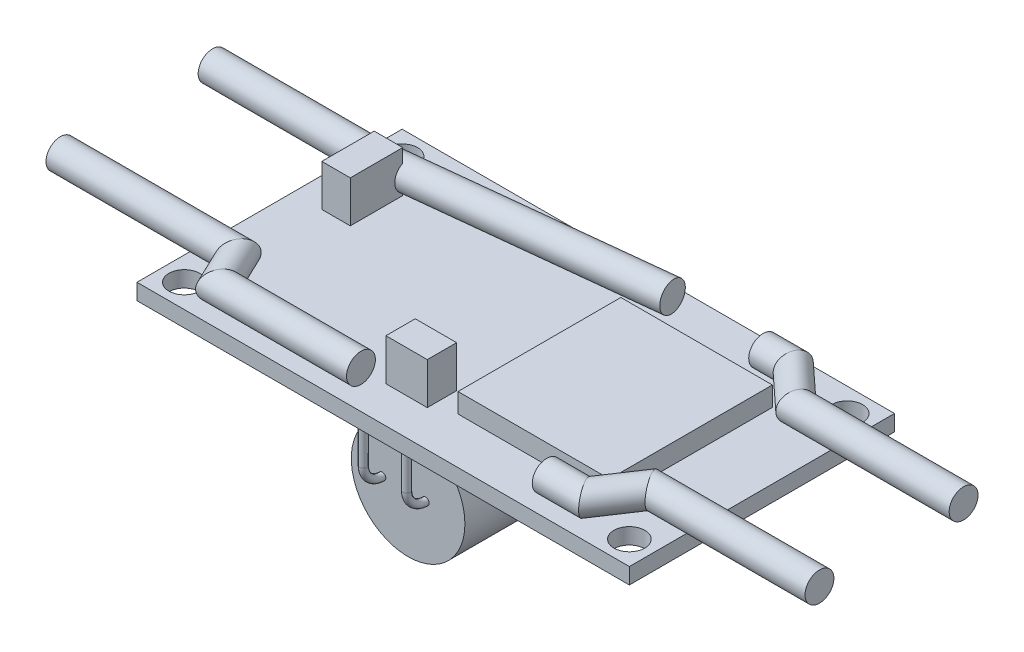
SolidWorks part; units mm, degrees
ref_plane "Front Plane" through (0, 0, 0) normal (0, 0, 1) x (1, 0, 0)
ref_plane "Top Plane" through (0, 0, 0) normal (0, 1, 0) x (1, 0, 0)
ref_plane "Right Plane" through (0, 0, 0) normal (1, 0, 0) x (0, 0, -1)
sketch "Sketch1" plane through (0, 0, 0) normal (0, 1, 0) x (1, 0, 0)
  line L0 (0, 0) -> (52, 0)
  line L1 (52, 0) -> (52, 28)
  line L2 (52, 28) -> (0, 28)
  line L3 (0, 28) -> (0, 0)
  line L4 (20.8, 22.3) -> (21.4, 21.7)
  line L5 (29.9, 2.3) -> (29.9, 0.5)
  line L6 (29, 1.4) -> (30.8, 1.4)
  line L7 (19.1, 1.4) -> (20.9, 1.4)
  line L8 (8, 21.3) -> (7.4, 21.8)
  line L9 (7.8, 22.8) -> (7.4, 23.1)
  line L10 (17.2, 20.7) -> (16.7, 20.6)
  line L11 (22.4, 3.3) -> (22.8, 3.3)
  line L12 (26.4, 3.2) -> (26.8, 3.2)
  line L13 (13.1032, 4.7492) -> (13.1032, 5.2064)
  line L14 (12.9762, 5.2064) -> (13.2302, 5.2064)
  line L15 (13.4629, 4.7492) -> (13.7677, 5.2064)
  line L16 (13.4629, 5.2064) -> (13.7677, 4.7492)
  line L17 (12.9762, 8.9762) -> (12.9762, 9.4334)
  line L18 (12.9762, 9.4334) -> (13.1032, 9.4334)
  line L19 (13.1032, 9.1794) -> (12.9762, 9.1794)
  line L20 (13.2302, 8.9762) -> (13.1286, 9.1794)
  line L21 (13.4921, 8.9762) -> (13.7969, 9.4334)
  line L22 (13.4921, 9.4334) -> (13.7969, 8.9762)
  line L23 (4.9666, 7.0984) -> (5.4238, 7.0984)
  line L24 (5.4238, 7.0984) -> (5.4238, 7.3016)
  line L25 (5.4238, 5.773) -> (4.9666, 5.773)
  line L26 (5.1698, 5.773) -> (5.1698, 6.027)
  line L27 (4.9666, 6.027) -> (5.4238, 6.027)
  line L28 (0.9794, 5.8656) -> (0.9794, 5.9418)
  line L29 (0.9794, 5.9418) -> (1.2334, 5.9418)
  line L30 (1.2334, 5.9418) -> (1.2334, 5.7894)
  line L31 (1.1318, 5.6878) -> (0.8778, 5.6878)
  line L32 (0.7762, 5.7894) -> (0.7762, 5.9418)
  line L33 (1.2334, 6.273) -> (0.7762, 6.273)
  line L34 (0.7762, 6.273) -> (1.2334, 6.527)
  line L35 (1.2334, 6.527) -> (0.7762, 6.527)
  line L36 (1.2334, 6.8582) -> (0.7762, 6.8582)
  line L37 (0.7762, 6.8582) -> (0.7762, 6.9852)
  line L38 (0.9032, 7.1122) -> (1.1064, 7.1122)
  line L39 (1.2334, 6.9852) -> (1.2334, 6.8582)
  line L40 (0.7762, 13.3844) -> (1.2334, 13.5368)
  line L41 (1.2334, 13.5368) -> (0.7762, 13.6892)
  line L42 (1.2334, 14.1584) -> (1.2334, 14.0568)
  line L43 (1.1318, 13.9552) -> (0.8778, 13.9552)
  line L44 (0.7762, 14.0568) -> (0.7762, 14.1584)
  line L45 (1.2334, 14.6156) -> (1.2334, 14.514)
  line L46 (1.1318, 14.4124) -> (0.8778, 14.4124)
  line L47 (0.7762, 14.514) -> (0.7762, 14.6156)
  line L48 (6.5937, 1.2914) -> (6.763, 1.2914)
  line L49 (6.763, 1.2914) -> (6.763, 0.727)
  line L50 (6.763, 0.727) -> (6.4244, 0.727)
  line L51 (6.1986, 0.9528) -> (6.1986, 1.5172)
  line L52 (6.4244, 1.743) -> (6.763, 1.743)
  line L53 (7.4178, 0.727) -> (7.4178, 1.743)
  line L54 (7.4178, 1.743) -> (7.9822, 0.727)
  line L55 (7.9822, 0.727) -> (7.9822, 1.743)
  line L56 (8.637, 0.727) -> (8.637, 1.743)
  line L57 (8.637, 1.743) -> (8.9192, 1.743)
  line L58 (9.2014, 1.4608) -> (9.2014, 1.0092)
  line L59 (8.9192, 0.727) -> (8.637, 0.727)
  line L60 (27.2698, 3.2656) -> (27.2698, 3.3418)
  line L61 (27.2698, 3.3418) -> (27.5238, 3.3418)
  line L62 (27.5238, 3.3418) -> (27.5238, 3.1894)
  line L63 (27.4222, 3.0878) -> (27.1682, 3.0878)
  line L64 (27.0666, 3.1894) -> (27.0666, 3.3418)
  line L65 (27.5238, 3.673) -> (27.0666, 3.673)
  line L66 (27.0666, 3.673) -> (27.5238, 3.927)
  line L67 (27.5238, 3.927) -> (27.0666, 3.927)
  line L68 (27.5238, 4.2582) -> (27.0666, 4.2582)
  line L69 (27.0666, 4.2582) -> (27.0666, 4.3852)
  line L70 (27.1936, 4.5122) -> (27.3968, 4.5122)
  line L71 (27.5238, 4.3852) -> (27.5238, 4.2582)
  line L72 (22.8238, 7.2646) -> (22.3666, 7.2646)
  line L73 (22.3666, 7.2646) -> (22.3666, 7.3916)
  line L74 (22.6206, 7.3916) -> (22.6206, 7.2646)
  line L75 (22.8238, 7.5186) -> (22.6206, 7.417)
  line L76 (22.6333, 7.9908) -> (22.5571, 7.8511)
  line L77 (22.8238, 8.4084) -> (22.3666, 8.4084)
  line L78 (22.3666, 8.2814) -> (22.3666, 8.5354)
  line L79 (24.8238, 8.7907) -> (24.8238, 8.6891)
  line L80 (24.7222, 8.5875) -> (24.4682, 8.5875)
  line L81 (24.3666, 8.6891) -> (24.3666, 8.7907)
  line L82 (24.3666, 9.0685) -> (24.8238, 9.0685)
  line L83 (24.8238, 9.0685) -> (24.8238, 9.2717)
  line L84 (24.8238, 9.5585) -> (24.3666, 9.5585)
  line L85 (24.3666, 9.8125) -> (24.646, 9.5585)
  line L86 (24.8238, 9.8125) -> (24.5444, 9.6601)
  line L87 (26.1238, 8.6249) -> (25.6666, 8.6249)
  line L88 (25.6666, 8.6249) -> (25.6666, 8.7519)
  line L89 (25.7936, 8.8789) -> (25.9968, 8.8789)
  line L90 (26.1238, 8.7519) -> (26.1238, 8.6249)
  line L91 (25.6666, 9.2091) -> (26.1238, 9.2091)
  line L92 (26.1238, 9.1583) -> (26.1238, 9.2599)
  line L93 (25.6666, 9.1583) -> (25.6666, 9.2599)
  line L94 (25.9968, 9.5211) -> (25.7936, 9.5211)
  line L95 (25.7936, 9.7751) -> (25.9968, 9.7751)
  line L96 (11.1656, 21.8302) -> (11.2418, 21.8302)
  line L97 (11.2418, 21.8302) -> (11.2418, 21.5762)
  line L98 (11.2418, 21.5762) -> (11.0894, 21.5762)
  line L99 (10.9878, 21.6778) -> (10.9878, 21.9318)
  line L100 (11.0894, 22.0334) -> (11.2418, 22.0334)
  line L101 (11.573, 21.5762) -> (11.573, 22.0334)
  line L102 (11.573, 22.0334) -> (11.827, 21.5762)
  line L103 (11.827, 21.5762) -> (11.827, 22.0334)
  line L104 (12.1582, 21.5762) -> (12.1582, 22.0334)
  line L105 (12.1582, 22.0334) -> (12.2852, 22.0334)
  line L106 (12.4122, 21.9064) -> (12.4122, 21.7032)
  line L107 (12.2852, 21.5762) -> (12.1582, 21.5762)
  line L108 (15.0896, 21.5762) -> (15.0896, 22.0334)
  line L109 (15.0896, 22.0334) -> (15.2166, 22.0334)
  line L110 (15.2166, 21.7794) -> (15.0896, 21.7794)
  line L111 (15.3436, 21.5762) -> (15.242, 21.7794)
  line L112 (15.6056, 21.5762) -> (15.9104, 22.0334)
  line L113 (15.6056, 22.0334) -> (15.9104, 21.5762)
  line L114 (13.1313, 21.5762) -> (13.1313, 22.0334)
  line L115 (13.0043, 22.0334) -> (13.2583, 22.0334)
  line L116 (13.4909, 21.5762) -> (13.7957, 22.0334)
  line L117 (13.4909, 22.0334) -> (13.7957, 21.5762)
  line L118 (0.7666, 11.2984) -> (1.2238, 11.2984)
  line L119 (1.2238, 11.2984) -> (1.2238, 11.5016)
  line L120 (1.2238, 8.773) -> (0.7666, 8.773)
  line L121 (0.9698, 8.773) -> (0.9698, 9.027)
  line L122 (0.7666, 9.027) -> (1.2238, 9.027)
  line L123 (0.8333, 17.8976) -> (0.7571, 17.7579)
  line L124 (1.0238, 18.4246) -> (1.0238, 18.323)
  line L125 (0.9222, 18.2214) -> (0.6682, 18.2214)
  line L126 (0.5666, 18.323) -> (0.5666, 18.4246)
  line L127 (0.5666, 18.7024) -> (1.0238, 18.7024)
  line L128 (1.0238, 18.7024) -> (1.0238, 18.9056)
  line L129 (0.8333, 19.5057) -> (0.7571, 19.366)
  line L130 (1.0238, 19.8512) -> (0.5666, 19.8512)
  line L131 (0.5666, 19.8512) -> (0.5666, 19.9782)
  line L132 (0.6936, 20.1052) -> (0.8968, 20.1052)
  line L133 (1.0238, 19.9782) -> (1.0238, 19.8512)
  line L134 (1.0238, 20.3927) -> (0.5666, 20.5451)
  line L135 (0.5666, 20.5451) -> (1.0238, 20.6975)
  line L136 (0.9095, 20.6594) -> (0.9095, 20.4308)
  line L137 (0.7698, 21.3656) -> (0.7698, 21.4418)
  line L138 (0.7698, 21.4418) -> (1.0238, 21.4418)
  line L139 (1.0238, 21.4418) -> (1.0238, 21.2894)
  line L140 (0.9222, 21.1878) -> (0.6682, 21.1878)
  line L141 (0.5666, 21.2894) -> (0.5666, 21.4418)
  line L142 (1.0238, 21.773) -> (0.5666, 21.773)
  line L143 (0.5666, 21.773) -> (1.0238, 22.027)
  line L144 (1.0238, 22.027) -> (0.5666, 22.027)
  line L145 (1.0238, 22.3582) -> (0.5666, 22.3582)
  line L146 (0.5666, 22.3582) -> (0.5666, 22.4852)
  line L147 (0.6936, 22.6122) -> (0.8968, 22.6122)
  line L148 (1.0238, 22.4852) -> (1.0238, 22.3582)
  line L149 (1.0238, 15.8244) -> (1.0238, 15.9514)
  line L150 (0.5666, 15.8244) -> (0.5666, 15.9768)
  line L151 (0.7698, 15.9768) -> (0.7698, 15.8752)
  line L152 (0.5666, 16.3476) -> (1.0238, 16.5)
  line L153 (1.0238, 16.5) -> (0.5666, 16.6524)
  line L154 (1.0238, 16.9216) -> (1.0238, 17.0486)
  line L155 (0.5666, 16.9216) -> (0.5666, 17.074)
  line L156 (0.7698, 17.074) -> (0.7698, 16.9724)
  line L157 (8.3334, 17.8476) -> (7.8762, 18)
  line L158 (7.8762, 18) -> (8.3334, 18.1524)
  line L159 (8.2191, 18.1143) -> (8.2191, 17.8857)
  line L160 (8.0794, 16.373) -> (8.0794, 16.5)
  line L161 (8.3334, 16.5) -> (8.3334, 16.373)
  line L162 (8.3334, 16.373) -> (7.8762, 16.373)
  line L163 (7.8762, 16.373) -> (7.8762, 16.5)
  line L164 (7.8762, 18.9371) -> (8.3334, 18.9371)
  line L165 (8.3334, 18.8863) -> (8.3334, 18.9879)
  line L166 (7.8762, 18.8863) -> (7.8762, 18.9879)
  line L167 (8.3334, 19.2673) -> (7.8762, 19.2673)
  line L168 (7.8762, 19.2673) -> (7.8762, 19.3943)
  line L169 (8.0032, 19.5213) -> (8.2064, 19.5213)
  line L170 (8.3334, 19.3943) -> (8.3334, 19.2673)
  line L171 (8.3334, 19.8089) -> (7.8762, 20.1137)
  line L172 (7.8762, 19.8089) -> (8.3334, 20.1137)
  line L173 (10.7744, 24.8762) -> (10.6728, 24.8762)
  line L174 (10.5712, 24.9778) -> (10.5712, 25.2318)
  line L175 (10.6728, 25.3334) -> (10.7744, 25.3334)
  line L176 (11.0499, 25.3334) -> (11.0499, 25.0032)
  line L177 (11.3039, 25.0032) -> (11.3039, 25.3334)
  line L178 (11.6424, 24.8762) -> (11.6424, 25.3334)
  line L179 (11.6424, 25.3334) -> (11.7694, 25.3334)
  line L180 (11.7694, 25.0794) -> (11.6424, 25.0794)
  line L181 (11.8964, 24.8762) -> (11.7948, 25.0794)
  line L182 (12.2094, 24.8762) -> (12.2094, 25.3334)
  line L183 (12.2094, 25.3334) -> (12.3364, 25.3334)
  line L184 (12.3364, 25.0794) -> (12.2094, 25.0794)
  line L185 (12.4634, 24.8762) -> (12.3618, 25.0794)
  line L186 (12.9744, 24.8762) -> (12.7712, 24.8762)
  line L187 (12.7712, 24.8762) -> (12.7712, 25.3334)
  line L188 (12.7712, 25.3334) -> (12.9744, 25.3334)
  line L189 (12.7712, 25.1302) -> (12.9236, 25.1302)
  line L190 (13.2445, 24.8762) -> (13.2445, 25.3334)
  line L191 (13.2445, 25.3334) -> (13.4985, 24.8762)
  line L192 (13.4985, 24.8762) -> (13.4985, 25.3334)
  line L193 (13.9018, 24.8762) -> (13.9018, 25.3334)
  line L194 (13.7748, 25.3334) -> (14.0288, 25.3334)
  line L195 (36.2048, 24.792) -> (36.2048, 25.808)
  line L196 (36.2048, 25.808) -> (36.5434, 25.2436)
  line L197 (36.5434, 25.2436) -> (36.8821, 25.808)
  line L198 (36.8821, 25.808) -> (36.8821, 24.792)
  line L199 (37.5185, 25.0742) -> (37.5185, 25.5258)
  line L200 (38.083, 25.5258) -> (38.083, 25.0742)
  line L201 (38.8675, 24.792) -> (38.8675, 25.808)
  line L202 (38.5853, 25.808) -> (39.1498, 25.808)
  line L203 (39.5957, 24.792) -> (39.9343, 25.808)
  line L204 (39.9343, 25.808) -> (40.273, 24.792)
  line L205 (40.1883, 25.046) -> (39.6803, 25.046)
  line L206 (36.0935, 1.892) -> (36.0935, 2.908)
  line L207 (36.0935, 2.908) -> (36.4321, 2.3436)
  line L208 (36.4321, 2.3436) -> (36.7708, 2.908)
  line L209 (36.7708, 2.908) -> (36.7708, 1.892)
  line L210 (37.4072, 2.1742) -> (37.4072, 2.6258)
  line L211 (37.9717, 2.6258) -> (37.9717, 2.1742)
  line L212 (38.7562, 1.892) -> (38.7562, 2.908)
  line L213 (38.474, 2.908) -> (39.0385, 2.908)
  line L214 (39.6086, 2.4564) -> (39.8908, 2.4564)
  line L215 (39.8908, 1.892) -> (39.6086, 1.892)
  line L216 (39.6086, 1.892) -> (39.6086, 2.908)
  line L217 (39.6086, 2.908) -> (39.8908, 2.908)
  line L218 (24.6753, 26.708) -> (25.014, 25.692)
  line L219 (25.014, 25.692) -> (25.3526, 26.708)
  line L220 (26.3205, 25.692) -> (26.0947, 25.692)
  line L221 (25.8689, 25.9178) -> (25.8689, 26.4822)
  line L222 (26.0947, 26.708) -> (26.3205, 26.708)
  line L223 (27.273, 25.692) -> (27.0472, 25.692)
  line L224 (26.8214, 25.9178) -> (26.8214, 26.4822)
  line L225 (27.0472, 26.708) -> (27.273, 26.708)
  line L226 (22.1238, 3.1244) -> (22.1238, 3.2514)
  line L227 (21.6666, 3.1244) -> (21.6666, 3.2768)
  line L228 (21.8698, 3.2768) -> (21.8698, 3.1752)
  line L229 (21.6666, 3.6476) -> (22.1238, 3.8)
  line L230 (22.1238, 3.8) -> (21.6666, 3.9524)
  line L231 (22.1238, 4.2216) -> (22.1238, 4.3486)
  line L232 (21.6666, 4.2216) -> (21.6666, 4.374)
  line L233 (21.8698, 4.374) -> (21.8698, 4.2724)
  line L234 (17.4334, 21.0244) -> (17.4334, 21.1514)
  line L235 (16.9762, 21.0244) -> (16.9762, 21.1768)
  line L236 (17.1794, 21.1768) -> (17.1794, 21.0752)
  line L237 (16.9762, 21.5476) -> (17.4334, 21.7)
  line L238 (17.4334, 21.7) -> (16.9762, 21.8524)
  line L239 (17.4334, 22.1216) -> (17.4334, 22.2486)
  line L240 (16.9762, 22.1216) -> (16.9762, 22.274)
  line L241 (17.1794, 22.274) -> (17.1794, 22.1724)
  line L242 (35.6428, 23.7684) -> (35.6428, 22.9387)
  line L243 (35.8799, 22.7016) -> (35.9984, 22.7016)
  line L244 (35.0783, 22.9387) -> (35.0783, 23.1757)
  line L245 (34.6041, 23.1757) -> (34.6041, 22.9387)
  line L246 (34.0396, 22.7016) -> (34.0396, 23.4128)
  line L247 (34.0396, 23.4128) -> (33.684, 23.4128)
  line L248 (33.684, 23.4128) -> (33.684, 23.2943)
  line L249 (32.8223, 23.7684) -> (32.8223, 22.7016)
  line L250 (32.8223, 22.7016) -> (33.1186, 22.7016)
  line L251 (33.2964, 22.8794) -> (33.2964, 23.235)
  line L252 (33.1186, 23.4128) -> (32.8223, 23.4128)
  line L253 (31.7936, 23.1165) -> (32.0603, 23.1165)
  line L254 (32.0603, 22.7016) -> (31.7936, 22.7016)
  line L255 (31.7936, 22.7016) -> (31.7936, 23.235)
  line L256 (31.9714, 23.4128) -> (32.2084, 23.4128)
  line L257 (31.1921, 22.7016) -> (31.1921, 23.4128)
  line L258 (31.1921, 23.4128) -> (30.8958, 23.4128)
  line L259 (30.718, 23.235) -> (30.718, 22.7016)
  line L260 (29.4733, 23.2943) -> (29.177, 23.2943)
  line L261 (29.177, 22.7016) -> (29.4733, 22.7016)
  line L262 (29.4733, 22.7016) -> (29.4733, 23.7684)
  line L263 (29.4733, 23.7684) -> (29.177, 23.7684)
  line L264 (28.3727, 23.4128) -> (28.3727, 22.8794)
  line L265 (28.1949, 22.7016) -> (27.8986, 22.7016)
  line L266 (27.8986, 22.7016) -> (27.8986, 23.4128)
  line L267 (27.2959, 22.7016) -> (27.2959, 23.4128)
  line L268 (27.2959, 23.4128) -> (26.9403, 23.4128)
  line L269 (26.9403, 23.4128) -> (26.9403, 23.2943)
  line L270 (26.4855, 22.7016) -> (26.4855, 23.7684)
  line L271 (26.0113, 23.4128) -> (26.4855, 23.0572)
  line L272 (26.0113, 22.7016) -> (26.278, 23.2054)
  line L273 (25.5499, 23.7684) -> (25.5499, 22.8794)
  line L274 (24.9056, 23.4128) -> (24.9056, 22.8794)
  line L275 (24.7278, 22.7016) -> (24.4315, 22.7016)
  line L276 (24.4315, 22.7016) -> (24.4315, 23.4128)
  line L277 (23.8388, 22.7016) -> (23.8388, 23.4128)
  line L278 (23.8388, 23.4128) -> (23.5425, 23.4128)
  line L279 (23.3647, 23.235) -> (23.3647, 22.7016)
  line L280 (22.3448, 23.7684) -> (22.3448, 22.7016)
  line L281 (22.3448, 22.7016) -> (22.6411, 22.7016)
  line L282 (22.8189, 22.8794) -> (22.8189, 23.235)
  line L283 (22.6411, 23.4128) -> (22.3448, 23.4128)
  line L284 (44.7349, 26.8193) -> (44.3229, 24.9651)
  line L285 (44.3229, 24.9651) -> (43.9108, 26.2012)
  line L286 (43.9108, 26.2012) -> (43.4988, 24.9651)
  line L287 (43.4988, 24.9651) -> (43.0867, 26.8193)
  line L288 (42.2312, 24.9651) -> (42.2312, 26.8193)
  line L289 (42.2312, 26.8193) -> (41.7162, 26.8193)
  line L290 (41.7162, 25.7892) -> (42.2312, 25.7892)
  line L291 (40.3267, 26.8193) -> (40.3267, 24.9651)
  line L292 (40.5328, 24.9651) -> (40.1207, 24.9651)
  line L293 (40.5328, 26.8193) -> (40.1207, 26.8193)
  line L294 (37.6077, 25.7377) -> (38.1743, 26.0467)
  line L295 (35.8473, 25.6862) -> (36.3108, 25.6862)
  line L296 (36.3108, 24.9651) -> (35.8473, 24.9651)
  line L297 (35.8473, 24.9651) -> (35.8473, 25.8922)
  line L298 (36.1563, 26.2012) -> (36.5684, 26.2012)
  line L299 (35.0124, 24.9651) -> (35.0124, 26.2012)
  line L300 (35.0639, 26.7163) -> (35.0639, 26.8193)
  line L301 (35.0639, 26.8193) -> (34.9609, 26.8193)
  line L302 (34.9609, 26.8193) -> (34.9609, 26.7163)
  line L303 (34.9609, 26.7163) -> (35.0639, 26.7163)
  line L304 (34.2305, 26.8193) -> (34.2305, 25.2741)
  line L305 (33.1888, 26.8193) -> (33.1888, 24.9651)
  line L306 (33.1888, 24.9651) -> (32.6738, 24.9651)
  line L307 (32.3648, 25.2741) -> (32.3648, 25.8922)
  line L308 (32.6738, 26.2012) -> (33.1888, 26.2012)
  line L309 (31.5932, 25.3771) -> (31.5932, 25.7892)
  line L310 (30.7691, 25.7892) -> (30.7691, 25.3771)
  line L311 (30.1485, 26.2012) -> (29.5305, 26.2012)
  line L312 (29.9425, 26.8193) -> (29.9425, 25.2741)
  line L313 (29.6335, 24.9651) -> (29.5305, 24.9651)
  line L314 (27.9062, 26.8193) -> (27.2881, 24.9651)
  line L315 (27.2881, 24.9651) -> (26.6701, 26.8193)
  line L316 (25.9493, 26.4073) -> (25.4343, 26.8193)
  line L317 (25.4343, 26.8193) -> (25.4343, 24.9651)
  line L318 (25.9493, 24.9651) -> (24.9192, 24.9651)
  line L319 (24.1881, 24.9651) -> (24.1881, 25.0681)
  line L320 (24.1881, 25.0681) -> (24.0851, 25.0681)
  line L321 (24.0851, 25.0681) -> (24.0851, 24.9651)
  line L322 (24.0851, 24.9651) -> (24.1881, 24.9651)
  line L323 (23.251, 25.3771) -> (22.4269, 26.4073)
  line L379 (18.0204, 24.3655) -> (17.9132, 24.3655)
  line L380 (17.8059, 24.4727) -> (17.8059, 24.7409)
  line L381 (17.9132, 24.8481) -> (18.0204, 24.8481)
  line L382 (18.266, 24.7409) -> (18.4, 24.8481)
  line L383 (18.4, 24.8481) -> (18.4, 24.3655)
  line L384 (18.266, 24.3655) -> (18.5341, 24.3655)
  line L385 (25.4204, 24.3519) -> (25.3132, 24.3519)
  line L386 (25.2059, 24.4591) -> (25.2059, 24.7273)
  line L387 (25.3132, 24.8345) -> (25.4204, 24.8345)
  line L388 (25.8939, 24.62) -> (25.666, 24.3519)
  line L389 (25.666, 24.3519) -> (25.9341, 24.3519)
  line L390 (14.9504, 8.1919) -> (14.8432, 8.1919)
  line L391 (14.7359, 8.2991) -> (14.7359, 8.5673)
  line L392 (14.8432, 8.6745) -> (14.9504, 8.6745)
  line L393 (15.196, 8.1919) -> (15.33, 8.1919)
  line L394 (15.196, 8.6745) -> (15.3568, 8.6745)
  line L395 (15.3568, 8.46) -> (15.2496, 8.46)
  line L396 (20.7081, 18.0504) -> (20.7081, 17.9432)
  line L397 (20.6009, 17.8359) -> (20.3327, 17.8359)
  line L398 (20.2255, 17.9432) -> (20.2255, 18.0504)
  line L399 (20.2255, 18.4032) -> (20.6009, 18.296)
  line L400 (20.6009, 18.296) -> (20.6009, 18.5641)
  line L401 (20.4936, 18.4837) -> (20.7081, 18.4837)
  line L402 (14.9504, 4.6919) -> (14.8432, 4.6919)
  line L403 (14.7359, 4.7991) -> (14.7359, 5.0673)
  line L404 (14.8432, 5.1745) -> (14.9504, 5.1745)
  line L405 (15.196, 4.6919) -> (15.3568, 4.6919)
  line L406 (15.4641, 4.7991) -> (15.4641, 4.8528)
  line L407 (15.3568, 4.96) -> (15.196, 4.96)
  line L408 (15.196, 4.96) -> (15.196, 5.1745)
  line L409 (15.196, 5.1745) -> (15.4641, 5.1745)
  line L410 (9.0504, 24.4919) -> (8.9432, 24.4919)
  line L411 (8.8359, 24.5991) -> (8.8359, 24.8673)
  line L412 (8.9432, 24.9745) -> (9.0504, 24.9745)
  line L413 (9.296, 24.76) -> (9.4568, 24.76)
  line L414 (9.5641, 24.6528) -> (9.5641, 24.626)
  line L415 (9.296, 24.626) -> (9.296, 24.76)
  line L416 (6.6504, 22.9919) -> (6.5432, 22.9919)
  line L417 (6.4359, 23.0991) -> (6.4359, 23.3673)
  line L418 (6.5432, 23.4745) -> (6.6504, 23.4745)
  line L419 (6.896, 23.4209) -> (6.896, 23.4745)
  line L420 (6.896, 23.4745) -> (7.1641, 23.4745)
  line L421 (7.1641, 23.4745) -> (7.03, 22.9919)
  line L422 (19.6496, 14.4255) -> (19.7568, 14.4255)
  line L423 (19.8641, 14.5327) -> (19.8641, 14.8009)
  line L424 (19.7568, 14.9081) -> (19.6496, 14.9081)
  line L425 (6.6504, 21.8919) -> (6.5432, 21.8919)
  line L426 (6.4359, 21.9991) -> (6.4359, 22.2673)
  line L427 (6.5432, 22.3745) -> (6.6504, 22.3745)
  line L428 (7.1641, 22.1064) -> (7.0032, 22.1064)
  line L429 (6.896, 22.2136) -> (6.896, 22.2404)
  line L430 (7.1641, 22.2404) -> (7.1641, 22.1064)
  line L434 (25.4239, 0.7469) -> (25.5312, 0.7469)
  line L435 (25.6384, 0.8541) -> (25.6384, 1.1223)
  line L436 (25.5312, 1.2295) -> (25.4239, 1.2295)
  line L437 (25.1783, 1.1223) -> (25.0443, 1.2295)
  line L438 (25.0443, 1.2295) -> (25.0443, 0.7469)
  line L439 (25.1783, 0.7469) -> (24.9102, 0.7469)
  line L440 (24.6029, 0.8541) -> (24.3884, 1.1223)
  line L441 (25.1239, 3.3255) -> (25.2312, 3.3255)
  line L442 (25.3384, 3.4327) -> (25.3384, 3.7009)
  line L443 (25.2312, 3.8081) -> (25.1239, 3.8081)
  line L444 (24.8783, 3.7009) -> (24.7443, 3.8081)
  line L445 (24.7443, 3.8081) -> (24.7443, 3.3255)
  line L446 (24.8783, 3.3255) -> (24.6102, 3.3255)
  line L447 (24.3297, 3.7009) -> (24.1957, 3.8081)
  line L448 (24.1957, 3.8081) -> (24.1957, 3.3255)
  line L449 (24.3297, 3.3255) -> (24.0616, 3.3255)
  line L450 (25.1239, 4.8255) -> (25.2312, 4.8255)
  line L451 (25.3384, 4.9327) -> (25.3384, 5.2009)
  line L452 (25.2312, 5.3081) -> (25.1239, 5.3081)
  line L453 (24.8783, 5.2009) -> (24.7443, 5.3081)
  line L454 (24.7443, 5.3081) -> (24.7443, 4.8255)
  line L455 (24.8783, 4.8255) -> (24.6102, 4.8255)
  line L456 (24.1018, 5.0936) -> (24.3297, 4.8255)
  line L457 (24.3297, 4.8255) -> (24.0616, 4.8255)
  line L458 (9.2569, 23.7761) -> (9.2569, 23.6688)
  line L459 (9.3641, 23.5616) -> (9.6323, 23.5616)
  line L460 (9.7395, 23.6688) -> (9.7395, 23.7761)
  line L461 (9.6323, 24.0217) -> (9.7395, 24.1557)
  line L462 (9.7395, 24.1557) -> (9.2569, 24.1557)
  line L463 (9.2569, 24.0217) -> (9.2569, 24.2898)
  line L464 (9.2569, 24.5703) -> (9.2569, 24.7044)
  line L465 (9.7395, 24.5703) -> (9.7395, 24.7312)
  line L466 (9.525, 24.7312) -> (9.525, 24.6239)
  line L467 (7.1919, 6.0761) -> (7.1919, 5.9688)
  line L468 (7.2991, 5.8616) -> (7.5673, 5.8616)
  line L469 (7.6745, 5.9688) -> (7.6745, 6.0761)
  line L470 (7.5673, 6.3217) -> (7.6745, 6.4557)
  line L471 (7.6745, 6.4557) -> (7.1919, 6.4557)
  line L472 (7.1919, 6.3217) -> (7.1919, 6.5898)
  line L473 (7.6745, 6.9775) -> (7.2991, 6.8703)
  line L474 (7.2991, 6.8703) -> (7.2991, 7.1384)
  line L475 (7.4064, 7.058) -> (7.1919, 7.058)
  line L476 (10.8919, 6.0761) -> (10.8919, 5.9688)
  line L477 (10.9991, 5.8616) -> (11.2673, 5.8616)
  line L478 (11.3745, 5.9688) -> (11.3745, 6.0761)
  line L479 (11.2673, 6.3217) -> (11.3745, 6.4557)
  line L480 (11.3745, 6.4557) -> (10.8919, 6.4557)
  line L481 (10.8919, 6.3217) -> (10.8919, 6.5898)
  line L482 (10.8919, 6.8703) -> (10.8919, 7.0312)
  line L483 (10.9991, 7.1384) -> (11.0528, 7.1384)
  line L484 (11.16, 7.0312) -> (11.16, 6.8703)
  line L485 (11.16, 6.8703) -> (11.3745, 6.8703)
  line L486 (11.3745, 6.8703) -> (11.3745, 7.1384)
  line L487 (5.9569, 23.7761) -> (5.9569, 23.6688)
  line L488 (6.0641, 23.5616) -> (6.3323, 23.5616)
  line L489 (6.4395, 23.6688) -> (6.4395, 23.7761)
  line L490 (6.3323, 24.0217) -> (6.4395, 24.1557)
  line L491 (6.4395, 24.1557) -> (5.9569, 24.1557)
  line L492 (5.9569, 24.0217) -> (5.9569, 24.2898)
  line L493 (6.225, 24.5703) -> (6.225, 24.7312)
  line L494 (6.1178, 24.8384) -> (6.091, 24.8384)
  line L495 (6.091, 24.5703) -> (6.225, 24.5703)
  line L496 (15.656, 3.934) -> (15.656, 0.886)
  line L497 (21.244, 0.886) -> (15.656, 0.886)
  line L498 (21.244, 0.886) -> (21.244, 3.934)
  line L499 (15.656, 3.934) -> (21.244, 3.934)
  line L500 (50.743, 16.234) -> (47.695, 16.234)
  line L501 (47.695, 10.646) -> (47.695, 16.234)
  line L502 (47.695, 10.646) -> (50.743, 10.646)
  line L503 (50.743, 16.234) -> (50.743, 10.646)
  line L504 (9.706, 3.934) -> (9.706, 0.886)
  line L505 (15.294, 0.886) -> (9.706, 0.886)
  line L506 (15.294, 0.886) -> (15.294, 3.934)
  line L507 (9.706, 3.934) -> (15.294, 3.934)
  line L508 (10.6616, 9.0392) -> (7.9184, 9.0392)
  line L509 (7.9184, 4.0608) -> (8.9852, 4.0608)
  line L510 (8.9852, 4.0608) -> (9.5948, 4.0608)
  line L511 (9.5948, 4.0608) -> (10.6616, 4.0608)
  line L512 (45, 22.1) -> (45, 4.9)
  line L513 (45, 4.9) -> (29, 4.9)
  line L514 (29, 4.9) -> (29, 22.1)
  line L515 (29, 22.1) -> (45, 22.1)
  line L516 (6.5, 16.56) -> (2.3, 16.56)
  line L517 (2.3, 21.64) -> (6.5, 21.64)
  line L518 (26.735, 7.1) -> (26.735, 4.1)
  line L519 (22.465, 4.1) -> (22.465, 7.1)
  line L520 (4.17, 7.015) -> (4.17, 5.745)
  line L521 (4.17, 5.745) -> (3.535, 5.11)
  line L522 (2.265, 5.11) -> (1.63, 5.745)
  line L523 (3.535, 10.19) -> (4.17, 9.555)
  line L524 (4.17, 9.555) -> (4.17, 8.285)
  line L525 (4.17, 8.285) -> (3.535, 7.65)
  line L526 (2.265, 7.65) -> (1.63, 8.285)
  line L527 (1.63, 8.285) -> (1.63, 9.555)
  line L528 (1.63, 9.555) -> (2.265, 10.19)
  line L529 (4.17, 7.015) -> (3.535, 7.65)
  line L530 (2.265, 7.65) -> (1.63, 7.015)
  line L531 (1.63, 5.745) -> (1.63, 7.015)
  line L532 (4.17, 14.635) -> (4.17, 13.365)
  line L533 (4.17, 13.365) -> (3.535, 12.73)
  line L534 (2.265, 12.73) -> (1.63, 13.365)
  line L535 (3.535, 12.73) -> (4.17, 12.095)
  line L536 (4.17, 12.095) -> (4.17, 10.825)
  line L537 (4.17, 10.825) -> (3.535, 10.19)
  line L538 (2.265, 10.19) -> (1.63, 10.825)
  line L539 (1.63, 10.825) -> (1.63, 12.095)
  line L540 (1.63, 12.095) -> (2.265, 12.73)
  line L541 (3.535, 15.27) -> (2.265, 15.27)
  line L542 (4.17, 14.635) -> (3.535, 15.27)
  line L543 (2.265, 15.27) -> (1.63, 14.635)
  line L544 (1.63, 13.365) -> (1.63, 14.635)
  line L545 (3.535, 5.11) -> (2.265, 5.11)
  line L546 (11.819, 19.511) -> (12.581, 19.511)
  line L547 (12.581, 19.511) -> (12.835, 19.765)
  line L548 (12.835, 19.765) -> (13.089, 19.511)
  line L549 (13.089, 19.511) -> (13.851, 19.511)
  line L550 (13.851, 19.511) -> (14.105, 19.765)
  line L551 (14.105, 19.765) -> (14.359, 19.511)
  line L552 (14.359, 19.511) -> (15.121, 19.511)
  line L553 (15.121, 19.511) -> (15.375, 19.765)
  line L554 (15.375, 19.765) -> (15.629, 19.511)
  line L555 (15.629, 19.511) -> (16.391, 19.511)
  line L556 (16.391, 21.289) -> (15.629, 21.289)
  line L557 (15.629, 21.289) -> (15.375, 21.035)
  line L558 (15.375, 21.035) -> (15.121, 21.289)
  line L559 (15.121, 21.289) -> (14.359, 21.289)
  line L560 (14.359, 21.289) -> (14.105, 21.035)
  line L561 (14.105, 21.035) -> (13.851, 21.289)
  line L562 (13.851, 21.289) -> (13.089, 21.289)
  line L563 (13.089, 21.289) -> (12.835, 21.035)
  line L564 (12.835, 21.035) -> (12.581, 21.289)
  line L565 (12.581, 21.289) -> (11.819, 21.289)
  line L566 (11.819, 21.289) -> (11.311, 20.781)
  line L567 (11.311, 20.019) -> (11.819, 19.511)
  line L568 (11.311, 20.781) -> (11.311, 20.019)
  line L569 (16.391, 21.289) -> (16.899, 20.781)
  line L570 (16.899, 20.781) -> (16.899, 20.019)
  line L571 (16.899, 20.019) -> (16.391, 19.511)
  line L572 (40.856, 26.794) -> (40.856, 23.746)
  line L573 (46.444, 23.746) -> (40.856, 23.746)
  line L574 (46.444, 23.746) -> (46.444, 26.794)
  line L575 (40.856, 26.794) -> (46.444, 26.794)
  line L576 (40.856, 3.934) -> (40.856, 0.886)
  line L577 (46.444, 0.886) -> (40.856, 0.886)
  line L578 (46.444, 0.886) -> (46.444, 3.934)
  line L579 (40.856, 3.934) -> (46.444, 3.934)
  line L580 (6.7948, 15.6255) -> (6.7948, 16.1081)
  line L581 (6.7948, 16.1081) -> (6.9289, 16.1081)
  line L582 (6.9289, 15.84) -> (6.7948, 15.84)
  line L583 (7.0629, 15.6255) -> (6.9557, 15.84)
  line L584 (7.3371, 16.0009) -> (7.4711, 16.1081)
  line L585 (7.4711, 16.1081) -> (7.4711, 15.6255)
  line L586 (7.3371, 15.6255) -> (7.6052, 15.6255)
  line L587 (10.3972, 19.1702) -> (10.7384, 19.5115)
  line L588 (10.7384, 19.5115) -> (10.8332, 19.4167)
  line L589 (10.6437, 19.2271) -> (10.5489, 19.3219)
  line L590 (10.5868, 18.9806) -> (10.6626, 19.2081)
  line L591 (11.1314, 18.8152) -> (10.7806, 18.7868)
  line L592 (10.7806, 18.7868) -> (10.9702, 18.5972)
  line L593 (6.2948, 12.2255) -> (6.2948, 12.7081)
  line L594 (6.2948, 12.7081) -> (6.4289, 12.7081)
  line L595 (6.4289, 12.44) -> (6.2948, 12.44)
  line L596 (6.5629, 12.2255) -> (6.4557, 12.44)
  line L597 (6.8371, 12.2255) -> (6.9711, 12.2255)
  line L598 (6.8371, 12.7081) -> (6.9979, 12.7081)
  line L599 (6.9979, 12.4936) -> (6.8907, 12.4936)
  line L600 (16.8745, 6.0948) -> (16.3919, 6.0948)
  line L601 (16.3919, 6.0948) -> (16.3919, 6.2289)
  line L602 (16.66, 6.2289) -> (16.66, 6.0948)
  line L603 (16.8745, 6.3629) -> (16.66, 6.2557)
  line L604 (16.3919, 6.7443) -> (16.7673, 6.6371)
  line L605 (16.7673, 6.6371) -> (16.7673, 6.9052)
  line L606 (16.66, 6.8248) -> (16.8745, 6.8248)
  line L607 (14.9669, 18.7291) -> (15.8291, 17.8669)
  line L608 (14.9669, 18.7291) -> (15.8291, 17.8669)
  line L609 (13.1709, 16.9331) -> (14.0331, 16.0709)
  line L610 (13.1709, 16.9331) -> (14.0331, 16.0709)
  line L611 (20.3745, 6.0948) -> (19.8919, 6.0948)
  line L612 (19.8919, 6.0948) -> (19.8919, 6.2289)
  line L613 (20.16, 6.2289) -> (20.16, 6.0948)
  line L614 (20.3745, 6.3629) -> (20.16, 6.2557)
  line L615 (20.1064, 6.6371) -> (20.1064, 6.7979)
  line L616 (20.2136, 6.9052) -> (20.2404, 6.9052)
  line L617 (20.2404, 6.6371) -> (20.1064, 6.6371)
  line L618 (26.4052, 20.1255) -> (26.4052, 20.6081)
  line L619 (26.4052, 20.6081) -> (26.2711, 20.6081)
  line L620 (26.2711, 20.34) -> (26.4052, 20.34)
  line L621 (26.1371, 20.1255) -> (26.2443, 20.34)
  line L622 (25.8629, 20.5545) -> (25.8629, 20.6081)
  line L623 (25.8629, 20.6081) -> (25.5948, 20.6081)
  line L624 (25.5948, 20.6081) -> (25.7289, 20.1255)
  line L625 (24.1052, 7.2255) -> (24.1052, 7.7081)
  line L626 (24.1052, 7.7081) -> (23.9711, 7.7081)
  line L627 (23.9711, 7.44) -> (24.1052, 7.44)
  line L628 (23.8371, 7.2255) -> (23.9443, 7.44)
  line L629 (17.2745, 17.7948) -> (16.7919, 17.7948)
  line L630 (16.7919, 17.7948) -> (16.7919, 17.9289)
  line L631 (17.06, 17.9289) -> (17.06, 17.7948)
  line L632 (17.2745, 18.0629) -> (17.06, 17.9557)
  line L633 (17.06, 18.6052) -> (17.06, 18.4443)
  line L634 (16.9528, 18.3371) -> (16.926, 18.3371)
  line L635 (16.926, 18.6052) -> (17.06, 18.6052)
  line L636 (22.2081, 18.2205) -> (21.7255, 18.2205)
  line L637 (21.7255, 18.2205) -> (21.7255, 18.3545)
  line L638 (21.9936, 18.3545) -> (21.9936, 18.2205)
  line L639 (22.2081, 18.4886) -> (21.9936, 18.3814)
  line L640 (21.8327, 18.7628) -> (21.7255, 18.8968)
  line L641 (21.7255, 18.8968) -> (22.2081, 18.8968)
  line L642 (22.2081, 18.7628) -> (22.2081, 19.0309)
  line L643 (22.1009, 19.3382) -> (21.8327, 19.5527)
  line L644 (24.0795, 15.3255) -> (24.0795, 15.8081)
  line L645 (24.0795, 15.8081) -> (23.9455, 15.8081)
  line L646 (23.9455, 15.54) -> (24.0795, 15.54)
  line L647 (23.8114, 15.3255) -> (23.9186, 15.54)
  line L648 (23.5372, 15.7009) -> (23.4032, 15.8081)
  line L649 (23.4032, 15.8081) -> (23.4032, 15.3255)
  line L650 (23.5372, 15.3255) -> (23.2691, 15.3255)
  line L651 (22.9886, 15.7009) -> (22.8545, 15.8081)
  line L652 (22.8545, 15.8081) -> (22.8545, 15.3255)
  line L653 (22.9886, 15.3255) -> (22.7205, 15.3255)
  line L654 (24.1795, 10.9255) -> (24.1795, 11.4081)
  line L655 (24.1795, 11.4081) -> (24.0455, 11.4081)
  line L656 (24.0455, 11.14) -> (24.1795, 11.14)
  line L657 (23.9114, 10.9255) -> (24.0186, 11.14)
  line L658 (23.6372, 11.3009) -> (23.5032, 11.4081)
  line L659 (23.5032, 11.4081) -> (23.5032, 10.9255)
  line L660 (23.6372, 10.9255) -> (23.3691, 10.9255)
  line L661 (22.8607, 11.1936) -> (23.0886, 10.9255)
  line L662 (23.0886, 10.9255) -> (22.8205, 10.9255)
  line L663 (24.0795, 17.3255) -> (24.0795, 17.8081)
  line L664 (24.0795, 17.8081) -> (23.9455, 17.8081)
  line L665 (23.9455, 17.54) -> (24.0795, 17.54)
  line L666 (23.8114, 17.3255) -> (23.9186, 17.54)
  line L667 (23.5372, 17.7009) -> (23.4032, 17.8081)
  line L668 (23.4032, 17.8081) -> (23.4032, 17.3255)
  line L669 (23.5372, 17.3255) -> (23.2691, 17.3255)
  line L670 (22.9886, 17.3255) -> (22.8545, 17.3255)
  line L671 (22.9886, 17.8081) -> (22.8277, 17.8081)
  line L672 (22.8277, 17.5936) -> (22.935, 17.5936)
  line L673 (24.0795, 9.4255) -> (24.0795, 9.9081)
  line L674 (24.0795, 9.9081) -> (23.9455, 9.9081)
  line L675 (23.9455, 9.64) -> (24.0795, 9.64)
  line L676 (23.8114, 9.4255) -> (23.9186, 9.64)
  line L677 (23.5372, 9.8009) -> (23.4032, 9.9081)
  line L678 (23.4032, 9.9081) -> (23.4032, 9.4255)
  line L679 (23.5372, 9.4255) -> (23.2691, 9.4255)
  line L680 (22.8814, 9.9081) -> (22.9886, 9.5327)
  line L681 (22.9886, 9.5327) -> (22.7205, 9.5327)
  line L682 (22.8009, 9.64) -> (22.8009, 9.4255)
  line L683 (24.1795, 13.1255) -> (24.1795, 13.6081)
  line L684 (24.1795, 13.6081) -> (24.0455, 13.6081)
  line L685 (24.0455, 13.34) -> (24.1795, 13.34)
  line L686 (23.9114, 13.1255) -> (24.0186, 13.34)
  line L687 (23.6372, 13.5009) -> (23.5032, 13.6081)
  line L688 (23.5032, 13.6081) -> (23.5032, 13.1255)
  line L689 (23.6372, 13.1255) -> (23.3691, 13.1255)
  line L690 (23.0886, 13.1255) -> (22.9277, 13.1255)
  line L691 (22.8205, 13.2327) -> (22.8205, 13.2864)
  line L692 (22.9277, 13.3936) -> (23.0886, 13.3936)
  line L693 (23.0886, 13.3936) -> (23.0886, 13.6081)
  line L694 (23.0886, 13.6081) -> (22.8205, 13.6081)
  line L695 (11.003, 24.416) -> (13.797, 24.416)
  line L696 (10.749, 24.162) -> (10.749, 22.638)
  line L697 (14.051, 24.162) -> (14.051, 22.638)
  line L698 (13.797, 22.384) -> (11.003, 22.384)
  line L699 (22.7, 8.7) -> (15.7, 8.7)
  line L700 (15.7, 8.7) -> (15.7, 15.7)
  line L701 (22.7, 8.7) -> (22.7, 15.7)
  line L702 (22.7, 15.7) -> (15.7, 15.7)
  line L703 (14.28, 22.9006) -> (14.28, 23.7594)
  line L704 (16.82, 23.7594) -> (16.82, 22.9006)
  line L705 (15.8184, 22.6212) -> (15.2816, 22.6212)
  line L706 (9.663, 12.903) -> (9.163, 12.903)
  line L707 (9.163, 12.903) -> (9.425, 13.403)
  line L708 (9.425, 13.403) -> (9.663, 12.903)
  line L709 (9.282, 13.1301) -> (9.282, 12.903)
  line L710 (9.409, 13.3725) -> (9.409, 12.903)
  line L711 (9.536, 13.1698) -> (9.536, 12.903)
  line L712 (10.663, 12.903) -> (10.163, 12.903)
  line L713 (10.163, 12.903) -> (10.425, 13.403)
  line L714 (10.425, 13.403) -> (10.663, 12.903)
  line L715 (10.171, 12.9183) -> (10.171, 12.903)
  line L716 (10.298, 13.1606) -> (10.298, 12.903)
  line L717 (10.425, 13.403) -> (10.425, 12.903)
  line L718 (10.552, 13.1362) -> (10.552, 12.903)
  line L719 (9.663, 13.403) -> (9.163, 13.403)
  line L720 (10.663, 13.403) -> (10.163, 13.403)
  line L721 (28.156, 26.794) -> (28.156, 23.746)
  line L722 (33.744, 23.746) -> (28.156, 23.746)
  line L723 (33.744, 23.746) -> (33.744, 26.794)
  line L724 (28.156, 26.794) -> (33.744, 26.794)
  line L725 (22.45, 20.73) -> (21.25, 20.73)
  line L726 (19.25, 22.13) -> (19.25, 22.73)
  line L727 (21.25, 24.13) -> (22.45, 24.13)
  line L728 (24.45, 22.13) -> (24.45, 22.73)
  line L729 (21.4, 10.9) -> (21.4, 9.5)
  line L730 (21.4, 9.5) -> (21.4, 4.9)
  line L731 (21.4, 4.9) -> (22.255, 4.9)
  line L732 (22.255, 4.9) -> (23.33, 3.825)
  line L733 (11.638, 23.4) -> (11.1, 23.4)
  line L734 (11.1, 23.4) -> (10.47, 23.4)
  line L735 (16.5, 15.5) -> (15.95, 16.05)
  line L736 (15.95, 16.05) -> (13.7, 18.3)
  line L737 (13.7, 18.3) -> (12, 18.3)
  line L738 (12, 18.3) -> (10.25, 20.05)
  line L739 (12, 18.3) -> (13.602, 16.698)
  line L740 (13.602, 16.698) -> (13.602, 16.502)
  line L741 (19.3, 4.75) -> (19.2, 4.75)
  line L742 (16.5, 15.5) -> (16.5, 15.1)
  line L743 (16.5, 15.1) -> (16.5, 14.5)
  line L744 (16.5, 14.5) -> (16.5, 13.2)
  line L745 (16.5, 13.2) -> (18, 11.7)
  line L746 (16.55, 14.45) -> (16.5, 14.5)
  line L747 (17.3, 17.4) -> (15.95, 16.05)
  line L748 (17.3, 17.4) -> (22.7, 17.4)
  line L749 (22.7, 17.4) -> (23.8, 17.4)
  line L750 (24.9568, 16.5068) -> (25.05, 16.9)
  line L751 (13.65, 7.5) -> (13.65, 5.9)
  line L752 (11.7538, 7.185) -> (13.335, 7.185)
  line L753 (13.335, 7.185) -> (13.65, 7.5)
  line L754 (20.6, 11.7) -> (21.4, 10.9)
  line L755 (18, 11.7) -> (20.6, 11.7)
  line L756 (19.45, 4.9) -> (19.3, 4.75)
  line L757 (8.5, 7.35) -> (10, 7.35)
  line L758 (25.05, 9.5) -> (21.4, 9.5)
  line L759 (10.25, 20.7) -> (10.25, 22)
  line L760 (10.25, 22) -> (10.05, 22.2)
  line L761 (10.25, 20.7) -> (10.25, 20.05)
  line L762 (10.05, 23.7) -> (10.05, 22.2)
  line L763 (24.3, 16.9) -> (25.05, 16.9)
  line L764 (23.8, 17.4) -> (24.3, 16.9)
  line L765 (2.45, 17.195) -> (4.7, 14.945)
  line L766 (4.7, 14.945) -> (4.7, 12.4)
  line L767 (4.7, 12.4) -> (7.6, 9.5)
  line L768 (7.6, 9.5) -> (8.5, 8.6)
  line L769 (8.5, 8.6) -> (8.5, 7.35)
  line L770 (10, 7.35) -> (10, 8.3)
  line L771 (10, 8.3) -> (10.1, 8.4)
  line L772 (10.1, 8.4) -> (10.1, 7.6)
  line L773 (10.515, 7.185) -> (11.7538, 7.185)
  line L774 (10.1, 7.6) -> (10.515, 7.185)
  line L775 (17.6, 4.75) -> (17.375, 4.975)
  line L776 (17.375, 4.975) -> (16.4, 5.95)
  line L777 (16.4, 5.95) -> (16.4, 7.9)
  line L778 (22, 16.5) -> (22.3, 16.8)
  line L779 (22.3, 16.8) -> (22.7, 16.8)
  line L780 (22.7, 16.8) -> (22.7, 17.4)
  line L781 (18.8, 16.5) -> (18.8, 16.1)
  line L782 (18.8, 16.1) -> (17.8, 15.1)
  line L783 (17.8, 15.1) -> (16.5, 15.1)
  line L784 (10.05, 23.7) -> (10.25, 23.4)
  line L785 (10.25, 23.4) -> (11.1, 23.4)
  line L786 (17.6, 4.75) -> (19.3, 4.75)
  line L787 (19.2, 4.75) -> (21.25, 4.75)
  line L788 (21.25, 4.75) -> (21.4, 4.9)
  line L789 (17.3544, 4.9544) -> (17.375, 4.975)
  line L790 (13.65, 5.9) -> (14.2, 5.35)
  line L791 (14.2, 5.35) -> (14.2, 4.8)
  line L792 (14.2, 4.8) -> (14.244, 4.756)
  line L793 (14.244, 4.756) -> (16.5, 4.756)
  line L794 (16.5, 4.756) -> (17.594, 4.756)
  line L795 (17.594, 4.756) -> (17.6, 4.75)
  line L796 (13.162, 23.4) -> (15.1299, 23.4)
  line L797 (15.1299, 23.4) -> (16.5, 22.0299)
  line L798 (16.01, 20.4) -> (16.5, 20.89)
  line L799 (16.5, 20.89) -> (16.5, 22.0299)
  line L800 (11.7538, 8.455) -> (13.545, 8.455)
  line L801 (13.545, 8.455) -> (13.6, 8.5)
  line L802 (13.6, 8.5) -> (18.2, 8.5)
  line L803 (18.2, 8.5) -> (19.6, 9.8)
  line L804 (19.6, 9.8) -> (19.6, 7.9)
  line L805 (11.7538, 4.645) -> (12.955, 4.645)
  line L806 (12.955, 4.645) -> (13.2, 4.4)
  line L807 (19.2, 4.4) -> (19.25, 4.45)
  line L808 (19.25, 4.45) -> (20.4, 5.6)
  line L809 (20.4, 5.6) -> (20.4, 7.9)
  line L810 (13.2, 4.4) -> (13.4, 4.2)
  line L811 (19, 4.2) -> (19.25, 4.45)
  line L812 (13.4, 4.2) -> (19, 4.2)
  line L813 (10.9, 17.5) -> (12.2, 17.5)
  line L814 (12.2, 17.5) -> (12.8, 18.1)
  line L815 (12.8, 18.1) -> (12.8, 19.1)
  line L816 (12.8, 19.1) -> (14.596, 19.1)
  line L817 (14.596, 19.1) -> (15.398, 18.298)
  line L818 (15.398, 18.298) -> (15.802, 18.298)
  line L819 (17.2, 16.9) -> (17.2, 16.5)
  line L820 (15.802, 18.298) -> (17.2, 16.9)
  line L821 (10.8, 17.6) -> (10.9, 17.5)
  line L822 (10.701, 17.699) -> (10.8, 17.6)
  line L823 (14.9, 12.6) -> (14.5, 12.6)
  line L824 (14.5, 12.6) -> (12.4, 14.7)
  line L825 (6.35, 18.465) -> (7.235, 18.465)
  line L826 (11.8, 16.2) -> (12.4, 15.6)
  line L827 (12.4, 15.6) -> (12.4, 14.7)
  line L828 (9.5, 16.2) -> (11.8, 16.2)
  line L829 (7.235, 18.465) -> (9.5, 16.2)
  line L830 (11.8, 15.3322) -> (11.3661, 15.7661)
  line L831 (8.6, 15.7661) -> (11.3661, 15.7661)
  line L832 (14.9, 11.8) -> (14.5, 11.8)
  line L833 (14.5, 11.8) -> (11.8, 14.5)
  line L834 (11.8, 14.5) -> (11.8, 15.3322)
  line L835 (6.35, 17.195) -> (7.1711, 17.195)
  line L836 (7.1711, 17.195) -> (8.6, 15.7661)
  line L837 (45.4, 10.9) -> (45.4, 8.1)
  line L838 (45.4, 8.1) -> (47.3, 8.1)
  line L839 (47.3, 8.1) -> (47.3, 10.9)
  line L840 (47.3, 10.9) -> (45.4, 10.9)
  line L841 (45.4, 16.1) -> (45.4, 18.9)
  line L842 (45.4, 18.9) -> (47.3, 18.9)
  line L843 (47.3, 18.9) -> (47.3, 16.1)
  line L844 (47.3, 16.1) -> (45.4, 16.1)
  line L845 (50.8, 10.8) -> (48.1, 8.1)
  line L846 (48.1, 8.1) -> (47.3, 8.1)
  line L847 (47.3, 8.1) -> (47.3, 10.9)
  line L848 (47.3, 10.9) -> (47.7, 11.3)
  line L849 (47.7, 11.3) -> (47.7, 15.7)
  line L850 (47.7, 15.7) -> (47.3, 16.1)
  line L851 (47.3, 16.1) -> (47.3, 18.9)
  line L852 (47.3, 18.9) -> (48.1, 18.9)
  line L853 (48.1, 18.9) -> (50.8, 16.2)
  line L854 (50.8, 16.2) -> (50.8, 10.8)
  line L855 (47.2, 18.9) -> (47.2, 22.3)
  line L856 (47.2, 22.3) -> (51, 22.3)
  line L857 (51, 22.3) -> (51, 4.7)
  line L858 (51, 4.7) -> (47.2, 4.7)
  line L859 (47.2, 4.7) -> (47.2, 18.9)
  line L860 (47.2, 22.3) -> (51, 22.3)
  line L861 (51, 22.3) -> (51, 4.7)
  line L862 (51, 4.7) -> (47.2, 4.7)
  line L863 (47.2, 4.7) -> (47.2, 22.3)
  line L864 (2.45, 21.005) -> (4.2225, 22.7775)
  line L865 (4.2225, 22.7775) -> (5.045, 23.6)
  line L866 (6.1, 15.9) -> (7.8, 15.9)
  line L867 (7.8, 15.9) -> (11.7546, 19.9444)
  line L868 (11.7546, 19.9444) -> (12.2, 20.4)
  line L869 (9.3, 9.4) -> (9.3, 5.9)
  line L870 (9.3, 5.9) -> (9.3, 3.3)
  line L871 (9.3, 3.3) -> (9.3, 2.4)
  line L872 (9.3, 2.4) -> (12.49, 2.4)
  line L873 (12.49, 2.4) -> (12.5, 2.41)
  line L874 (5.85, 12.85) -> (9.3, 9.4)
  line L875 (11.7538, 5.915) -> (9.315, 5.915)
  line L876 (9.315, 5.915) -> (9.3, 5.9)
  line L877 (6.48, 2.4) -> (9.3, 2.4)
  line L878 (12.49, 1.89) -> (12.49, 2.4)
  line L879 (25.56, 21.58) -> (25.7, 21.52)
  line L880 (12.2, 20.4) -> (12.5636, 20.7636)
  line L881 (12.5636, 20.7636) -> (12.5636, 20.7754)
  line L882 (12.5636, 20.7754) -> (12.7941, 21.0059)
  line L883 (12.7941, 21.0059) -> (15.0882, 23.3)
  line L884 (15.0882, 23.3) -> (16.8, 23.3)
  line L885 (16.8, 23.3) -> (17.2, 23.3)
  line L886 (17.2, 23.3) -> (18.12, 23.3)
  line L887 (18.12, 23.3) -> (18.14, 23.28)
  line L888 (16.3804, 23.3) -> (16.8, 23.3)
  line L889 (18.14, 23.28) -> (18.14, 24.34)
  line L890 (18.14, 24.34) -> (18.6, 24.8)
  line L891 (18.6, 24.8) -> (26, 24.8)
  line L892 (26, 24.8) -> (26.5, 24.3)
  line L893 (26.5936, 24.1936) -> (26.5, 24.3)
  line L894 (25.56, 21.58) -> (25.9736, 21.58)
  line L895 (25.56, 21.58) -> (25.56, 20.86)
  line L896 (24.45, 19.75) -> (22.9, 19.75)
  line L897 (25.56, 20.86) -> (24.45, 19.75)
  line L898 (19.5, 19.85) -> (18.65, 20.7)
  line L899 (18.65, 20.7) -> (17.5, 20.7)
  line L900 (17.5, 20.7) -> (17.2, 21)
  line L901 (17.2, 21) -> (17.2, 23.3)
  line L902 (12.2, 20.4) -> (11.65, 20.95)
  line L903 (12.5, 2.41) -> (18.45, 2.41)
  line L904 (12.5, 2.41) -> (13.31, 1.6)
  line L905 (13.31, 1.6) -> (17.6, 1.6)
  line L906 (12.5, 2.41) -> (12.745, 2.155)
  line L907 (12.745, 2.155) -> (13.29, 3.2)
  line L908 (13.29, 3.2) -> (17.6, 3.2)
  line L909 (25.87, 3.825) -> (25.87, 2.57)
  line L910 (18.86, 2.1) -> (18.45, 2.41)
  line L911 (26.5936, 22.2) -> (26.5936, 24.1936)
  line L912 (25.9736, 21.58) -> (26.5936, 22.2)
  line L913 (2.9, 6.38) -> (6.48, 2.4)
  line L914 (8.55, 19.85) -> (9.499, 18.901)
  line L915 (13.8, 3.2) -> (13.29, 3.2)
  line L916 (8.5, 5.65) -> (8.5, 3.3)
  line L917 (8.5, 3.3) -> (9.3, 3.3)
  line L918 (10, 5.65) -> (8.5, 5.65)
  line L919 (12.7941, 21.0059) -> (11.7059, 21.0059)
  line L920 (11.7059, 21.0059) -> (11.65, 20.95)
  line L921 (11.7546, 19.9444) -> (11.65, 20.049)
  line L922 (11.65, 20.049) -> (11.65, 20.95)
  line L923 (8.35, 22.2) -> (8.35, 20.9)
  line L924 (8.35, 20.9) -> (8.55, 20.7)
  line L925 (8.55, 20.7) -> (8.55, 19.85)
  line L926 (18.8, 13.75) -> (18.65, 13.6)
  line L927 (26.25, 5) -> (26.25, 3.4)
  line L928 (25.87, 2.57) -> (25.4, 2.1)
  line L929 (20, 2.1) -> (18.86, 2.1)
  line L930 (21.8, 2.1) -> (20.9, 2.1)
  line L931 (20.9, 2.1) -> (20, 2.1)
  line L932 (22.5, 1.4) -> (21.8, 2.1)
  line L933 (25.4, 2.1) -> (20.9, 2.1)
  line L934 (26.25, 3.4) -> (24.25, 1.4)
  line L935 (24.25, 1.4) -> (22.5, 1.4)
  line L936 (6.7, 20.4) -> (5, 22.1)
  line L937 (5, 22.1) -> (4.3225, 22.7775)
  line L938 (4.3225, 22.7775) -> (4.2225, 22.7775)
  line L939 (12.2, 20.4) -> (7.8, 20.4)
  line L940 (7.8, 20.4) -> (6.7, 20.4)
  line L941 (7.9, 22.445) -> (7.8, 22.345)
  line L942 (7.8, 22.345) -> (7.8, 20.4)
  line L943 (11.2, 22.445) -> (11.2, 21.5118)
  line L944 (11.2, 21.5118) -> (11.7059, 21.0059)
  line L945 (5.85, 13.4) -> (5.85, 12.85)
  line L946 (5.85, 13.4) -> (5.85, 14.9)
  line L947 (5.85, 14.9) -> (5.85, 15.65)
  line L948 (5.85, 15.65) -> (6.1, 15.9)
  line L949 (15.35, 7.5) -> (15.35, 5.9)
  line L950 (15.35, 7.5) -> (14.9, 7.95)
  line L951 (14.9, 7.95) -> (14.9, 9.4)
  line L952 (15.35, 5.9) -> (15.35, 4.76)
  line L953 (15.35, 4.76) -> (12.745, 2.155)
  line L954 (14.9, 9.4) -> (15.6, 9.4)
  line L955 (15.6, 9.4) -> (17.6, 11.4)
  line L956 (23.5, 16.1) -> (23.5, 15)
  line L957 (18.8, 13.75) -> (18.8, 14)
  line L958 (18.65, 13.6) -> (17.6, 13.6)
  line L959 (17.6, 13.6) -> (17.6, 11.4)
  line L960 (8.35, 23.7) -> (8.35, 22.2)
  line L961 (5.045, 23.6) -> (8.25, 23.6)
  line L962 (8.25, 23.6) -> (8.35, 23.7)
  line L963 (18.8, 14) -> (20.9, 16.1)
  line L964 (20.9, 16.1) -> (23.5, 16.1)
  line L965 (15.55, 24.6301) -> (15.55, 24.1304)
  line L966 (15.55, 24.1304) -> (16.3804, 23.3)
  line L967 (46.15, 18.5) -> (26.5936, 22.2)
  line L968 (2.45, 18.465) -> (4.365, 18.465)
  line L969 (4.365, 18.465) -> (4.4, 18.5)
  line L970 (4.4, 18.5) -> (4.4, 15)
  line L971 (9.5, 9.9) -> (16.5, 9.9)
  line L972 (16.5, 9.9) -> (18, 9.9)
  line L973 (18, 9.9) -> (18, 7.9)
  line L974 (4.4, 15) -> (9.5, 9.9)
  line L975 (17.6, 6.45) -> (18, 6.85)
  line L976 (18, 6.85) -> (18, 7.9)
  line L977 (2.45, 19.735) -> (4.365, 19.735)
  line L978 (4.365, 19.735) -> (4.4, 19.7)
  line L979 (4.4, 19.7) -> (5.2, 18.9)
  line L980 (9.7, 10.9) -> (18.8, 10.9)
  line L981 (18.8, 10.9) -> (18.8, 7.9)
  line L982 (5.2, 18.9) -> (5.2, 15.4)
  line L983 (5.2, 15.4) -> (9.7, 10.9)
  line L984 (19.2, 6.45) -> (18.8, 6.85)
  line L985 (18.8, 6.85) -> (18.8, 7.9)
  line L986 (14.9, 13.4) -> (14.5, 13.4)
  line L987 (6.35, 19.735) -> (7.165, 19.735)
  line L988 (13.1, 14.8) -> (14.5, 13.4)
  line L989 (12.1, 16.6) -> (13.1, 15.6)
  line L990 (13.1, 15.6) -> (13.1, 14.8)
  line L991 (10.3, 16.6) -> (12.1, 16.6)
  line L992 (7.165, 19.735) -> (10.3, 16.6)
  line L993 (46.3, 26.8) -> (46.3, 22.3)
  line L994 (46.3, 22.3) -> (45, 20.8)
  line L995 (45, 20.8) -> (43.7, 22.1)
  line L996 (43.7, 22.1) -> (37.4, 22.1)
  line L997 (37.4, 22.1) -> (37.4, 26.8)
  line L998 (37.4, 26.8) -> (46.3, 26.8)
  line L999 (37.4, 13.8) -> (44.9, 13.8)
  line L1000 (44.9, 13.8) -> (44.9, 22.1)
  line L1001 (44.9, 22.1) -> (37.4, 22.1)
  line L1002 (37.4, 22.1) -> (37.4, 13.8)
  line L1003 (37.4, 13.8) -> (44.9, 13.8)
  line L1004 (44.9, 13.8) -> (44.9, 20.9)
  line L1005 (44.9, 20.9) -> (46.3, 22.3)
  line L1006 (46.3, 22.3) -> (46.3, 26.8)
  line L1007 (46.3, 26.8) -> (37.4, 26.8)
  line L1008 (37.4, 26.8) -> (37.4, 13.8)
  line L1009 (43.65, 25.27) -> (42.82, 26.1)
  line L1010 (42.82, 26.1) -> (40.7, 26.1)
  line L1011 (43.65, 25.27) -> (42.78, 24.4)
  line L1012 (42.78, 24.4) -> (40.6, 24.4)
  line L1013 (43.65, 25.27) -> (42.8, 24.42)
  line L1014 (42.8, 24.42) -> (42.8, 23.6)
  line L1015 (43.65, 25.27) -> (44.5, 24.42)
  line L1016 (44.5, 24.42) -> (44.5, 23.4)
  line L1017 (43.65, 25.27) -> (42.73, 25.27)
  line L1018 (42.73, 25.27) -> (42.7, 25.3)
  line L1019 (42.7, 25.3) -> (41.9, 24.5)
  line L1020 (41.9, 24.5) -> (41.9, 23.3)
  line L1021 (43.65, 25.27) -> (44.47, 25.27)
  line L1022 (44.47, 25.27) -> (44.5, 25.3)
  line L1023 (44.5, 25.3) -> (45.4, 24.4)
  line L1024 (45.4, 24.4) -> (45.4, 23.4)
  line L1025 (46.15, 20.5) -> (44.4, 20.5)
  line L1026 (46.15, 15.5) -> (43.6, 15.5)
  line L1027 (43.6, 15.5) -> (43.5, 15.6)
  line L1028 (46.4, 0.9) -> (46.4, 4.7)
  line L1029 (46.4, 4.7) -> (45, 6.1)
  line L1030 (45, 6.1) -> (43.8, 4.9)
  line L1031 (43.8, 4.9) -> (37.4, 4.9)
  line L1032 (37.4, 4.9) -> (37.4, 0.9)
  line L1033 (37.4, 0.9) -> (46.4, 0.9)
  line L1034 (37.4, 13.2) -> (37.4, 4.9)
  line L1035 (37.4, 4.9) -> (44.9, 4.9)
  line L1036 (44.9, 4.9) -> (44.9, 13.2)
  line L1037 (44.9, 13.2) -> (37.4, 13.2)
  line L1038 (37.4, 13.2) -> (44.9, 13.2)
  line L1039 (44.9, 13.2) -> (44.9, 6.2)
  line L1040 (44.9, 6.2) -> (46.4, 4.7)
  line L1041 (46.4, 4.7) -> (46.4, 0.9)
  line L1042 (46.4, 0.9) -> (37.4, 0.9)
  line L1043 (37.4, 0.9) -> (37.4, 13.2)
  line L1044 (43.65, 2.41) -> (42.86, 3.2)
  line L1045 (42.86, 3.2) -> (40.4, 3.2)
  line L1046 (43.65, 2.41) -> (42.84, 1.6)
  line L1047 (42.84, 1.6) -> (40.1, 1.6)
  line L1048 (43.65, 2.41) -> (44.5, 3.26)
  line L1049 (44.5, 3.26) -> (44.5, 4.1)
  line L1050 (43.65, 2.41) -> (44.64, 3.4)
  line L1051 (44.64, 3.4) -> (45.3, 3.4)
  line L1052 (45.3, 3.4) -> (45.3, 4.3)
  line L1053 (43.65, 2.41) -> (42.8, 3.26)
  line L1054 (42.8, 3.26) -> (42.8, 4)
  line L1055 (43.65, 2.41) -> (42.61, 2.41)
  line L1056 (42.61, 2.41) -> (42.6, 2.4)
  line L1057 (42.6, 2.4) -> (41.9, 3.1)
  line L1058 (41.9, 3.1) -> (41.9, 4)
  line L1059 (46.15, 6.5) -> (42.3, 6.5)
  line L1060 (46.15, 11.5) -> (43.8, 11.5)
  line L1061 (18, 18.15) -> (19.5, 18.15)
  line L1062 (18, 18.15) -> (18, 16.5)
  line L1063 (24.1, 19) -> (16.9, 19)
  line L1064 (16.9, 19) -> (17.75, 19.85)
  line L1065 (17.75, 19.85) -> (18, 19.85)
  line L1066 (24.1, 19) -> (24.5, 19)
  line L1067 (24.5, 19) -> (25.1, 18.4)
  line L1068 (25.1, 18.4) -> (25.1, 14.2)
  line L1069 (25.1, 14.2) -> (25.8, 13.5)
  line L1070 (25.8, 13.5) -> (27.85, 13.5)
  line L1071 (24.1, 19) -> (23.85, 19)
  line L1072 (23.85, 19) -> (22.9, 18.05)
  line L1073 (23.7, 23.58) -> (21.8, 21.68)
  line L1074 (21.8, 20.9) -> (21.2, 20.3)
  line L1075 (21.2, 20.3) -> (21.2, 16.5)
  line L1076 (21.8, 21.68) -> (21.8, 20.9)
  line L1077 (25.56, 23.28) -> (25.26, 23.58)
  line L1078 (25.26, 23.58) -> (23.7, 23.58)
  line L1079 (20, 21.28) -> (20.4, 20.88)
  line L1080 (20.4, 20.88) -> (20.4, 16.5)
  line L1081 (18.14, 21.58) -> (18.44, 21.28)
  line L1082 (18.44, 21.28) -> (20, 21.28)
  line L1083 (26.75, 13.2) -> (26.75, 14.25)
  line L1084 (26.75, 14.25) -> (26.7, 14.3)
  line L1085 (26.7, 14.3) -> (26.9, 14.5)
  line L1086 (26.9, 14.5) -> (27.85, 14.5)
  line L1087 (26.75, 16.9) -> (26.75, 15.4)
  line L1088 (26.75, 16.9) -> (25.8, 17.85)
  line L1089 (25.8, 17.85) -> (25.8, 18.1)
  line L1090 (25.8, 18.1) -> (25.8, 17.2)
  line L1091 (25.8, 17.2) -> (26.5, 16.5)
  line L1092 (26.5, 16.5) -> (27.85, 16.5)
  line L1093 (24, 13.4) -> (23.5, 13.4)
  line L1094 (24.4, 18.1) -> (24.6, 17.9)
  line L1095 (24.6, 14) -> (24, 13.4)
  line L1096 (24.6, 17.9) -> (24.6, 14)
  line L1097 (25.25, 19.2) -> (25.25, 18.95)
  line L1098 (25.25, 18.95) -> (24.4, 18.1)
  line L1099 (25.05, 11) -> (25.05, 12.05)
  line L1100 (25.05, 12.05) -> (25, 12.1)
  line L1101 (25, 12.1) -> (24.7, 11.8)
  line L1102 (24.7, 11.8) -> (23.5, 11.8)
  line L1103 (25.9, 12.1) -> (25.9, 11.6)
  line L1104 (25.9, 11.6) -> (25.3, 11)
  line L1105 (25.3, 11) -> (23.5, 11)
  line L1106 (25.05, 7.3) -> (25.05, 8.0549)
  line L1107 (25.8794, 12.0794) -> (25.9, 12.1)
  line L1108 (25.05, 8.0549) -> (25.8794, 8.8843)
  line L1109 (25.8794, 8.8843) -> (25.8794, 12.0794)
  line L1110 (27.85, 17.5) -> (27.3, 17.5)
  line L1111 (27.3, 17.5) -> (26.7, 18.1)
  line L1112 (26.7, 18.1) -> (26.95, 18.35)
  line L1113 (26.95, 18.35) -> (26.95, 19.2)
  line L1114 (7.55, 14.9) -> (8.691, 14.9)
  line L1115 (8.691, 14.9) -> (9.092, 14.499)
  line L1116 (26.75, 7.3) -> (26.75, 8.3956)
  line L1117 (26.75, 8.3956) -> (26.7456, 8.4)
  line L1118 (26.7456, 8.4) -> (26.7456, 11.2456)
  line L1119 (26.7456, 11.2456) -> (27, 11.5)
  line L1120 (27, 11.5) -> (27.85, 11.5)
  line L1121 (10.742, 11.799) -> (11.541, 11)
  line L1122 (11.541, 11) -> (14.9, 11)
  line L1123 (14.9, 10.2) -> (10.3, 10.2)
  line L1124 (9.092, 11.408) -> (9.092, 11.799)
  line L1125 (10.3, 10.2) -> (9.092, 11.408)
  line L1126 (10.742, 14.499) -> (10.742, 13.442)
  line L1127 (10.5, 13.2) -> (10.742, 13.442)
  line L1128 (7.55, 13.4) -> (7.85, 13.2)
  line L1129 (7.85, 13.2) -> (10.5, 13.2)
  line L1130 (6.8262, 7.185) -> (5.615, 7.185)
  line L1131 (5.615, 7.185) -> (5, 7.8)
  line L1132 (5, 7.8) -> (5, 9.36)
  line L1133 (5, 9.36) -> (2.9, 11.46)
  line L1134 (6.8262, 5.915) -> (5.905, 5.915)
  line L1135 (5.905, 5.915) -> (2.9, 8.92)
  line L1136 (25.05, 13.2) -> (22.7, 13.2)
  line L1137 (22.7, 13.2) -> (22.1, 13.8)
  line L1138 (22.1, 13.8) -> (22.5, 14.2)
  line L1139 (22.5, 14.2) -> (23.5, 14.2)
  line L1140 (26.75, 11) -> (26.75, 12.05)
  line L1141 (26.75, 12.05) -> (26.7, 12.1)
  line L1142 (26.7, 12.1) -> (27.1, 12.5)
  line L1143 (27.1, 12.5) -> (27.85, 12.5)
  line L1144 (26.75, 11) -> (26.75, 9.5)
  line L1145 (22, 15.1) -> (21.3, 14.4)
  line L1146 (21.3, 13.3) -> (22, 12.6)
  line L1147 (22, 12.6) -> (23.5, 12.6)
  line L1148 (21.3, 14.4) -> (21.3, 13.3)
  line L1149 (25.05, 15.4) -> (22.3, 15.4)
  line L1150 (22.3, 15.4) -> (22, 15.1)
  line L1151 (19.6, 16.5) -> (19.6, 12.6)
  line L1152 (19.6, 12.6) -> (19.6, 11.8)
  line L1153 (23.33, 8.07) -> (23.33, 7.375)
  line L1154 (19.6, 11.8) -> (23.33, 8.07)
  line L1155 (20.35, 13.6) -> (20.35, 12.75)
  line L1156 (20.35, 12.75) -> (20.2, 12.6)
  line L1157 (20.2, 12.6) -> (19.6, 12.6)
  line L1158 (21.2, 7.9) -> (21.2, 6.4)
  line L1159 (21.2, 6.4) -> (22.1, 5.5)
  line L1160 (22.1, 5.5) -> (24.6, 5.5)
  line L1161 (25.87, 6.77) -> (25.87, 7.375)
  line L1162 (24.6, 5.5) -> (25.87, 6.77)
  line L1163 (22, 7.9) -> (22, 6.3)
  line L1164 (22, 6.3) -> (22.3, 6)
  line L1165 (22.3, 6) -> (23.9, 6)
  line L1166 (24.6, 6.7) -> (24.6, 7.375)
  line L1167 (23.9, 6) -> (24.6, 6.7)
  line L1168 (14.9, 15) -> (14.9, 16.7)
  line L1169 (13.47, 18.13) -> (13.47, 20.4)
  line L1170 (14.9, 16.7) -> (13.47, 18.13)
  line L1171 (16.4, 16.5) -> (15.8, 16.5)
  line L1172 (14, 19.66) -> (14.74, 20.4)
  line L1173 (15.8, 16.5) -> (14, 18.3)
  line L1174 (14, 18.3) -> (14, 19.66)
  line L1175 (28.2, 23.8) -> (29.2, 22.8)
  line L1176 (29.2, 22.8) -> (29.2, 22.1)
  line L1177 (29.2, 22.1) -> (36.6, 22.1)
  line L1178 (36.6, 22.1) -> (36.6, 26.7)
  line L1179 (36.6, 26.7) -> (28.2, 26.7)
  line L1180 (28.2, 26.7) -> (28.2, 23.8)
  line L1181 (36.6, 1) -> (36.6, 22.1)
  line L1182 (36.6, 22.1) -> (29.2, 22.1)
  line L1183 (29.2, 22.1) -> (29.2, 1)
  line L1184 (29.2, 1) -> (36.6, 1)
  line L1185 (29.2, 1) -> (36.6, 1)
  line L1186 (36.6, 1) -> (36.6, 26.7)
  line L1187 (36.6, 26.7) -> (28.2, 26.7)
  line L1188 (28.2, 26.7) -> (28.2, 23.8)
  line L1189 (28.2, 23.8) -> (29.2, 22.8)
  line L1190 (29.2, 22.8) -> (29.2, 1)
  line L1191 (30.9199, 25.3001) -> (30.95, 25.27)
  line L1192 (2.9, 14) -> (2.9, 21.7)
  line L1193 (16.5, 24.6301) -> (16.5, 25.9)
  line L1194 (27.85, 8.5) -> (27.95, 8.4)
  line L1195 (27.95, 8.4) -> (29.6, 8.4)
  line L1196 (27.85, 9.5) -> (29.5, 9.5)
  line L1197 (27.85, 18.5) -> (30.1, 18.5)
  line L1198 (30.95, 25.27) -> (29.8, 24.12)
  line L1199 (29.8, 24.12) -> (29.8, 23.7)
  line L1200 (30.95, 25.27) -> (32.1, 24.12)
  line L1201 (32.1, 24.12) -> (32.1, 23.4)
  line L1202 (30.95, 25.27) -> (31.83, 25.27)
  line L1203 (33, 24.1) -> (33, 23.5)
  line L1204 (31.83, 25.27) -> (33, 24.1)
  line L1205 (30.95, 25.27) -> (29.43, 25.27)
  line L1206 (30.95, 25.27) -> (29.97, 25.27)
  line L1207 (28.9, 24.2) -> (28.9, 23.6)
  line L1208 (29.97, 25.27) -> (28.9, 24.2)
  line L1209 (30.95, 25.27) -> (31.82, 24.4)
  line L1210 (30.95, 25.27) -> (31.88, 26.2)
  line L1211 (31.88, 26.2) -> (35, 26.2)
  line L1212 (30.95, 25.27) -> (31.92, 24.3)
  line L1213 (31.92, 24.3) -> (34.5, 24.3)
  line L1214 (16.5, 25.9) -> (28.8, 25.9)
  line L1215 (28.8, 25.9) -> (29.43, 25.27)
  line L1216 (27.95, 3.4) -> (29.7, 3.4)
  line L1217 (27.95, 5) -> (30, 5)
  line L1218 (27.5, 1.4) -> (28, 1.9)
  line L1219 (28, 1.9) -> (30.2, 1.9)
  line L1220 (5.6, 25.9) -> (14.6, 25.9)
  line L1221 (14.6, 25.9) -> (16.5, 25.9)
  line L1222 (11.2, 25.955) -> (7.9, 25.955)
  line L1223 (7.9, 25.955) -> (7.845, 25.9)
  line L1224 (7.845, 25.9) -> (5.6, 25.9)
  line L1225 (5.6, 24.4) -> (5.6, 25.9)
  line L1226 (2.9, 21.7) -> (5.6, 24.4)
  line L1227 (14.6, 24.6301) -> (14.6, 25.9)
  arc A0 (21.3731, 21.6731) -> (21.4269, 21.7269) centre (21.4, 21.7) ccw
  arc A1 (20.8269, 22.3269) -> (20.7731, 22.2731) centre (20.8, 22.3) ccw
  arc A2 (29.773, 0.5) -> (30.027, 0.5) centre (29.9, 0.5) ccw
  arc A3 (30.027, 2.3) -> (29.773, 2.3) centre (29.9, 2.3) ccw
  arc A4 (30.8, 1.273) -> (30.8, 1.527) centre (30.8, 1.4) ccw
  arc A5 (29, 1.527) -> (29, 1.273) centre (29, 1.4) ccw
  arc A6 (20.9, 1.273) -> (20.9, 1.527) centre (20.9, 1.4) ccw
  arc A7 (19.1, 1.527) -> (19.1, 1.273) centre (19.1, 1.4) ccw
  arc A8 (7.432, 21.8384) -> (7.368, 21.7616) centre (7.4, 21.8) ccw
  arc A9 (7.968, 21.2616) -> (8.032, 21.3384) centre (8, 21.3) ccw
  arc A10 (7.43, 23.14) -> (7.37, 23.06) centre (7.4, 23.1) ccw
  arc A11 (7.77, 22.76) -> (7.83, 22.84) centre (7.8, 22.8) ccw
  arc A12 (16.6902, 20.649) -> (16.7098, 20.551) centre (16.7, 20.6) ccw
  arc A13 (17.2098, 20.651) -> (17.1902, 20.749) centre (17.2, 20.7) ccw
  arc A14 (22.8, 3.25) -> (22.8, 3.35) centre (22.8, 3.3) ccw
  arc A15 (22.4, 3.35) -> (22.4, 3.25) centre (22.4, 3.3) ccw
  arc A16 (26.8, 3.15) -> (26.8, 3.25) centre (26.8, 3.2) ccw
  arc A17 (26.4, 3.25) -> (26.4, 3.15) centre (26.4, 3.2) ccw
  arc A18 (13.1413, 5.2064) -> (13.0651, 5.2064) centre (13.1032, 5.2064) ccw
  arc A19 (13.0651, 4.7492) -> (13.1413, 4.7492) centre (13.1032, 4.7492) ccw
  arc A20 (13.2302, 5.1683) -> (13.2302, 5.2445) centre (13.2302, 5.2064) ccw
  arc A21 (12.9762, 5.2445) -> (12.9762, 5.1683) centre (12.9762, 5.2064) ccw
  arc A22 (13.7994, 5.1853) -> (13.736, 5.2275) centre (13.7677, 5.2064) ccw
  arc A23 (13.4312, 4.7703) -> (13.4946, 4.7281) centre (13.4629, 4.7492) ccw
  arc A24 (13.736, 4.7281) -> (13.7994, 4.7703) centre (13.7677, 4.7492) ccw
  arc A25 (13.4946, 5.2275) -> (13.4312, 5.1853) centre (13.4629, 5.2064) ccw
  arc A26 (13.0143, 9.4334) -> (12.9381, 9.4334) centre (12.9762, 9.4334) ccw
  arc A27 (12.9381, 8.9762) -> (13.0143, 8.9762) centre (12.9762, 8.9762) ccw
  arc A28 (13.1032, 9.3953) -> (13.1032, 9.4715) centre (13.1032, 9.4334) ccw
  arc A29 (12.9762, 9.4715) -> (12.9762, 9.3953) centre (12.9762, 9.4334) ccw
  arc A30 (13.1032, 9.1794) -> (13.1032, 9.4334) centre (13.1032, 9.3064) ccw
  arc A31 (13.1032, 9.2175) -> (13.1032, 9.1413) centre (13.1032, 9.1794) ccw
  arc A32 (13.1032, 9.4715) -> (13.1032, 9.3953) centre (13.1032, 9.4334) ccw
  arc A33 (12.9762, 9.2175) -> (12.9762, 9.1413) centre (12.9762, 9.1794) ccw
  arc A34 (13.1032, 9.1413) -> (13.1032, 9.2175) centre (13.1032, 9.1794) ccw
  arc A35 (13.1627, 9.1964) -> (13.0945, 9.1624) centre (13.1286, 9.1794) ccw
  arc A36 (13.1961, 8.9592) -> (13.2643, 8.9932) centre (13.2302, 8.9762) ccw
  arc A37 (13.8286, 9.4123) -> (13.7652, 9.4545) centre (13.7969, 9.4334) ccw
  arc A38 (13.4604, 8.9973) -> (13.5238, 8.9551) centre (13.4921, 8.9762) ccw
  arc A39 (13.7652, 8.9551) -> (13.8286, 8.9973) centre (13.7969, 8.9762) ccw
  arc A40 (13.5238, 9.4545) -> (13.4604, 9.4123) centre (13.4921, 9.4334) ccw
  arc A41 (5.4238, 7.0603) -> (5.4238, 7.1365) centre (5.4238, 7.0984) ccw
  arc A42 (4.9666, 7.1365) -> (4.9666, 7.0603) centre (4.9666, 7.0984) ccw
  arc A43 (5.4619, 7.3016) -> (5.3857, 7.3016) centre (5.4238, 7.3016) ccw
  arc A44 (5.3857, 7.0984) -> (5.4619, 7.0984) centre (5.4238, 7.0984) ccw
  arc A45 (4.9666, 5.8111) -> (4.9666, 5.7349) centre (4.9666, 5.773) ccw
  arc A46 (5.4238, 5.7349) -> (5.4238, 5.8111) centre (5.4238, 5.773) ccw
  arc A47 (5.2079, 6.027) -> (5.1317, 6.027) centre (5.1698, 6.027) ccw
  arc A48 (5.1317, 5.773) -> (5.2079, 5.773) centre (5.1698, 5.773) ccw
  arc A49 (5.4238, 5.9889) -> (5.4238, 6.0651) centre (5.4238, 6.027) ccw
  arc A50 (4.9666, 6.0651) -> (4.9666, 5.9889) centre (4.9666, 6.027) ccw
  arc A51 (1.0175, 5.9418) -> (0.9413, 5.9418) centre (0.9794, 5.9418) ccw
  arc A52 (0.9413, 5.8656) -> (1.0175, 5.8656) centre (0.9794, 5.8656) ccw
  arc A53 (1.2334, 5.9037) -> (1.2334, 5.9799) centre (1.2334, 5.9418) ccw
  arc A54 (0.9794, 5.9799) -> (0.9794, 5.9037) centre (0.9794, 5.9418) ccw
  arc A55 (1.1953, 5.7894) -> (1.2715, 5.7894) centre (1.2334, 5.7894) ccw
  arc A56 (1.2715, 5.9418) -> (1.1953, 5.9418) centre (1.2334, 5.9418) ccw
  arc A57 (1.1318, 5.6878) -> (1.2334, 5.7894) centre (1.1318, 5.7894) ccw
  arc A58 (1.1318, 5.7259) -> (1.1318, 5.6497) centre (1.1318, 5.6878) ccw
  arc A59 (1.2715, 5.7894) -> (1.1953, 5.7894) centre (1.2334, 5.7894) ccw
  arc A60 (0.8778, 5.7259) -> (0.8778, 5.6497) centre (0.8778, 5.6878) ccw
  arc A61 (1.1318, 5.6497) -> (1.1318, 5.7259) centre (1.1318, 5.6878) ccw
  arc A62 (0.7762, 5.7894) -> (0.8778, 5.6878) centre (0.8778, 5.7894) ccw
  arc A63 (0.8143, 5.7894) -> (0.7381, 5.7894) centre (0.7762, 5.7894) ccw
  arc A64 (0.8778, 5.6497) -> (0.8778, 5.7259) centre (0.8778, 5.6878) ccw
  arc A65 (0.8143, 5.9418) -> (0.7381, 5.9418) centre (0.7762, 5.9418) ccw
  arc A66 (0.7381, 5.7894) -> (0.8143, 5.7894) centre (0.7762, 5.7894) ccw
  arc A67 (0.7762, 6.3111) -> (0.7762, 6.2349) centre (0.7762, 6.273) ccw
  arc A68 (1.2334, 6.2349) -> (1.2334, 6.3111) centre (1.2334, 6.273) ccw
  arc A69 (1.2519, 6.4937) -> (1.2149, 6.5603) centre (1.2334, 6.527) ccw
  arc A70 (0.7577, 6.3063) -> (0.7947, 6.2397) centre (0.7762, 6.273) ccw
  arc A71 (0.7762, 6.5651) -> (0.7762, 6.4889) centre (0.7762, 6.527) ccw
  arc A72 (1.2334, 6.4889) -> (1.2334, 6.5651) centre (1.2334, 6.527) ccw
  arc A73 (0.7762, 6.8963) -> (0.7762, 6.8201) centre (0.7762, 6.8582) ccw
  arc A74 (1.2334, 6.8201) -> (1.2334, 6.8963) centre (1.2334, 6.8582) ccw
  arc A75 (0.8143, 6.9852) -> (0.7381, 6.9852) centre (0.7762, 6.9852) ccw
  arc A76 (0.7381, 6.8582) -> (0.8143, 6.8582) centre (0.7762, 6.8582) ccw
  arc A77 (0.9032, 7.1122) -> (0.7762, 6.9852) centre (0.9032, 6.9852) ccw
  arc A78 (0.9032, 7.0741) -> (0.9032, 7.1503) centre (0.9032, 7.1122) ccw
  arc A79 (0.7381, 6.9852) -> (0.8143, 6.9852) centre (0.7762, 6.9852) ccw
  arc A80 (1.1064, 7.0741) -> (1.1064, 7.1503) centre (1.1064, 7.1122) ccw
  arc A81 (0.9032, 7.1503) -> (0.9032, 7.0741) centre (0.9032, 7.1122) ccw
  arc A82 (1.2334, 6.9852) -> (1.1064, 7.1122) centre (1.1064, 6.9852) ccw
  arc A83 (1.1953, 6.9852) -> (1.2715, 6.9852) centre (1.2334, 6.9852) ccw
  arc A84 (1.1064, 7.1503) -> (1.1064, 7.0741) centre (1.1064, 7.1122) ccw
  arc A85 (1.1953, 6.8582) -> (1.2715, 6.8582) centre (1.2334, 6.8582) ccw
  arc A86 (1.2715, 6.9852) -> (1.1953, 6.9852) centre (1.2334, 6.9852) ccw
  arc A87 (1.2454, 13.5007) -> (1.2214, 13.573) centre (1.2334, 13.5368) ccw
  arc A88 (0.7642, 13.4206) -> (0.7882, 13.3483) centre (0.7762, 13.3844) ccw
  arc A89 (0.7882, 13.7254) -> (0.7642, 13.6531) centre (0.7762, 13.6892) ccw
  arc A90 (1.2214, 13.5007) -> (1.2454, 13.573) centre (1.2334, 13.5368) ccw
  arc A91 (1.1953, 14.0568) -> (1.2715, 14.0568) centre (1.2334, 14.0568) ccw
  arc A92 (1.2715, 14.1584) -> (1.1953, 14.1584) centre (1.2334, 14.1584) ccw
  arc A93 (1.1318, 13.9552) -> (1.2334, 14.0568) centre (1.1318, 14.0568) ccw
  arc A94 (1.1318, 13.9933) -> (1.1318, 13.9171) centre (1.1318, 13.9552) ccw
  arc A95 (1.2715, 14.0568) -> (1.1953, 14.0568) centre (1.2334, 14.0568) ccw
  arc A96 (0.8778, 13.9933) -> (0.8778, 13.9171) centre (0.8778, 13.9552) ccw
  arc A97 (1.1318, 13.9171) -> (1.1318, 13.9933) centre (1.1318, 13.9552) ccw
  arc A98 (0.7762, 14.0568) -> (0.8778, 13.9552) centre (0.8778, 14.0568) ccw
  arc A99 (0.8143, 14.0568) -> (0.7381, 14.0568) centre (0.7762, 14.0568) ccw
  arc A100 (0.8778, 13.9171) -> (0.8778, 13.9933) centre (0.8778, 13.9552) ccw
  arc A101 (0.8143, 14.1584) -> (0.7381, 14.1584) centre (0.7762, 14.1584) ccw
  arc A102 (0.7381, 14.0568) -> (0.8143, 14.0568) centre (0.7762, 14.0568) ccw
  arc A103 (1.1953, 14.514) -> (1.2715, 14.514) centre (1.2334, 14.514) ccw
  arc A104 (1.2715, 14.6156) -> (1.1953, 14.6156) centre (1.2334, 14.6156) ccw
  arc A105 (1.1318, 14.4124) -> (1.2334, 14.514) centre (1.1318, 14.514) ccw
  arc A106 (1.1318, 14.4505) -> (1.1318, 14.3743) centre (1.1318, 14.4124) ccw
  arc A107 (1.2715, 14.514) -> (1.1953, 14.514) centre (1.2334, 14.514) ccw
  arc A108 (0.8778, 14.4505) -> (0.8778, 14.3743) centre (0.8778, 14.4124) ccw
  arc A109 (1.1318, 14.3743) -> (1.1318, 14.4505) centre (1.1318, 14.4124) ccw
  arc A110 (0.7762, 14.514) -> (0.8778, 14.4124) centre (0.8778, 14.514) ccw
  arc A111 (0.8143, 14.514) -> (0.7381, 14.514) centre (0.7762, 14.514) ccw
  arc A112 (0.8778, 14.3743) -> (0.8778, 14.4505) centre (0.8778, 14.4124) ccw
  arc A113 (0.8143, 14.6156) -> (0.7381, 14.6156) centre (0.7762, 14.6156) ccw
  arc A114 (0.7381, 14.514) -> (0.8143, 14.514) centre (0.7762, 14.514) ccw
  arc A115 (6.763, 1.2279) -> (6.763, 1.3549) centre (6.763, 1.2914) ccw
  arc A116 (6.5937, 1.3549) -> (6.5937, 1.2279) centre (6.5937, 1.2914) ccw
  arc A117 (6.6995, 0.727) -> (6.8265, 0.727) centre (6.763, 0.727) ccw
  arc A118 (6.8265, 1.2914) -> (6.6995, 1.2914) centre (6.763, 1.2914) ccw
  arc A119 (6.4244, 0.7905) -> (6.4244, 0.6635) centre (6.4244, 0.727) ccw
  arc A120 (6.763, 0.6635) -> (6.763, 0.7905) centre (6.763, 0.727) ccw
  arc A121 (6.1986, 0.9528) -> (6.4244, 0.727) centre (6.4244, 0.9528) ccw
  arc A122 (6.2621, 0.9528) -> (6.1351, 0.9528) centre (6.1986, 0.9528) ccw
  arc A123 (6.4244, 0.6635) -> (6.4244, 0.7905) centre (6.4244, 0.727) ccw
  arc A124 (6.2621, 1.5172) -> (6.1351, 1.5172) centre (6.1986, 1.5172) ccw
  arc A125 (6.1351, 0.9528) -> (6.2621, 0.9528) centre (6.1986, 0.9528) ccw
  arc A126 (6.4244, 1.743) -> (6.1986, 1.5172) centre (6.4244, 1.5172) ccw
  arc A127 (6.4244, 1.6795) -> (6.4244, 1.8065) centre (6.4244, 1.743) ccw
  arc A128 (6.1351, 1.5172) -> (6.2621, 1.5172) centre (6.1986, 1.5172) ccw
  arc A129 (6.763, 1.6795) -> (6.763, 1.8065) centre (6.763, 1.743) ccw
  arc A130 (6.4244, 1.8065) -> (6.4244, 1.6795) centre (6.4244, 1.743) ccw
  arc A131 (7.4813, 1.743) -> (7.3543, 1.743) centre (7.4178, 1.743) ccw
  arc A132 (7.3543, 0.727) -> (7.4813, 0.727) centre (7.4178, 0.727) ccw
  arc A133 (7.9267, 0.6962) -> (8.0377, 0.7578) centre (7.9822, 0.727) ccw
  arc A134 (7.4733, 1.7738) -> (7.3623, 1.7122) centre (7.4178, 1.743) ccw
  arc A135 (8.0457, 1.743) -> (7.9187, 1.743) centre (7.9822, 1.743) ccw
  arc A136 (7.9187, 0.727) -> (8.0457, 0.727) centre (7.9822, 0.727) ccw
  arc A137 (8.7005, 1.743) -> (8.5735, 1.743) centre (8.637, 1.743) ccw
  arc A138 (8.5735, 0.727) -> (8.7005, 0.727) centre (8.637, 0.727) ccw
  arc A139 (8.9192, 1.6795) -> (8.9192, 1.8065) centre (8.9192, 1.743) ccw
  arc A140 (8.637, 1.8065) -> (8.637, 1.6795) centre (8.637, 1.743) ccw
  arc A141 (9.2014, 1.4608) -> (8.9192, 1.743) centre (8.9192, 1.4608) ccw
  arc A142 (9.1379, 1.4608) -> (9.2649, 1.4608) centre (9.2014, 1.4608) ccw
  arc A143 (8.9192, 1.8065) -> (8.9192, 1.6795) centre (8.9192, 1.743) ccw
  arc A144 (9.1379, 1.0092) -> (9.2649, 1.0092) centre (9.2014, 1.0092) ccw
  arc A145 (9.2649, 1.4608) -> (9.1379, 1.4608) centre (9.2014, 1.4608) ccw
  arc A146 (8.9192, 0.727) -> (9.2014, 1.0092) centre (8.9192, 1.0092) ccw
  arc A147 (8.9192, 0.7905) -> (8.9192, 0.6635) centre (8.9192, 0.727) ccw
  arc A148 (9.2649, 1.0092) -> (9.1379, 1.0092) centre (9.2014, 1.0092) ccw
  arc A149 (8.637, 0.7905) -> (8.637, 0.6635) centre (8.637, 0.727) ccw
  arc A150 (8.9192, 0.6635) -> (8.9192, 0.7905) centre (8.9192, 0.727) ccw
  arc A151 (27.3079, 3.3418) -> (27.2317, 3.3418) centre (27.2698, 3.3418) ccw
  arc A152 (27.2317, 3.2656) -> (27.3079, 3.2656) centre (27.2698, 3.2656) ccw
  arc A153 (27.5238, 3.3037) -> (27.5238, 3.3799) centre (27.5238, 3.3418) ccw
  arc A154 (27.2698, 3.3799) -> (27.2698, 3.3037) centre (27.2698, 3.3418) ccw
  arc A155 (27.4857, 3.1894) -> (27.5619, 3.1894) centre (27.5238, 3.1894) ccw
  arc A156 (27.5619, 3.3418) -> (27.4857, 3.3418) centre (27.5238, 3.3418) ccw
  arc A157 (27.4222, 3.0878) -> (27.5238, 3.1894) centre (27.4222, 3.1894) ccw
  arc A158 (27.4222, 3.1259) -> (27.4222, 3.0497) centre (27.4222, 3.0878) ccw
  arc A159 (27.5619, 3.1894) -> (27.4857, 3.1894) centre (27.5238, 3.1894) ccw
  arc A160 (27.1682, 3.1259) -> (27.1682, 3.0497) centre (27.1682, 3.0878) ccw
  arc A161 (27.4222, 3.0497) -> (27.4222, 3.1259) centre (27.4222, 3.0878) ccw
  arc A162 (27.0666, 3.1894) -> (27.1682, 3.0878) centre (27.1682, 3.1894) ccw
  arc A163 (27.1047, 3.1894) -> (27.0285, 3.1894) centre (27.0666, 3.1894) ccw
  arc A164 (27.1682, 3.0497) -> (27.1682, 3.1259) centre (27.1682, 3.0878) ccw
  arc A165 (27.1047, 3.3418) -> (27.0285, 3.3418) centre (27.0666, 3.3418) ccw
  arc A166 (27.0285, 3.1894) -> (27.1047, 3.1894) centre (27.0666, 3.1894) ccw
  arc A167 (27.0666, 3.7111) -> (27.0666, 3.6349) centre (27.0666, 3.673) ccw
  arc A168 (27.5238, 3.6349) -> (27.5238, 3.7111) centre (27.5238, 3.673) ccw
  arc A169 (27.5423, 3.8937) -> (27.5053, 3.9603) centre (27.5238, 3.927) ccw
  arc A170 (27.0481, 3.7063) -> (27.0851, 3.6397) centre (27.0666, 3.673) ccw
  arc A171 (27.0666, 3.9651) -> (27.0666, 3.8889) centre (27.0666, 3.927) ccw
  arc A172 (27.5238, 3.8889) -> (27.5238, 3.9651) centre (27.5238, 3.927) ccw
  arc A173 (27.0666, 4.2963) -> (27.0666, 4.2201) centre (27.0666, 4.2582) ccw
  arc A174 (27.5238, 4.2201) -> (27.5238, 4.2963) centre (27.5238, 4.2582) ccw
  arc A175 (27.1047, 4.3852) -> (27.0285, 4.3852) centre (27.0666, 4.3852) ccw
  arc A176 (27.0285, 4.2582) -> (27.1047, 4.2582) centre (27.0666, 4.2582) ccw
  arc A177 (27.1936, 4.5122) -> (27.0666, 4.3852) centre (27.1936, 4.3852) ccw
  arc A178 (27.1936, 4.4741) -> (27.1936, 4.5503) centre (27.1936, 4.5122) ccw
  arc A179 (27.0285, 4.3852) -> (27.1047, 4.3852) centre (27.0666, 4.3852) ccw
  arc A180 (27.3968, 4.4741) -> (27.3968, 4.5503) centre (27.3968, 4.5122) ccw
  arc A181 (27.1936, 4.5503) -> (27.1936, 4.4741) centre (27.1936, 4.5122) ccw
  arc A182 (27.5238, 4.3852) -> (27.3968, 4.5122) centre (27.3968, 4.3852) ccw
  arc A183 (27.4857, 4.3852) -> (27.5619, 4.3852) centre (27.5238, 4.3852) ccw
  arc A184 (27.3968, 4.5503) -> (27.3968, 4.4741) centre (27.3968, 4.5122) ccw
  arc A185 (27.4857, 4.2582) -> (27.5619, 4.2582) centre (27.5238, 4.2582) ccw
  arc A186 (27.5619, 4.3852) -> (27.4857, 4.3852) centre (27.5238, 4.3852) ccw
  arc A187 (22.3666, 7.3027) -> (22.3666, 7.2265) centre (22.3666, 7.2646) ccw
  arc A188 (22.8238, 7.2265) -> (22.8238, 7.3027) centre (22.8238, 7.2646) ccw
  arc A189 (22.4047, 7.3916) -> (22.3285, 7.3916) centre (22.3666, 7.3916) ccw
  arc A190 (22.3285, 7.2646) -> (22.4047, 7.2646) centre (22.3666, 7.2646) ccw
  arc A191 (22.6206, 7.3916) -> (22.3666, 7.3916) centre (22.4936, 7.3916) ccw
  arc A192 (22.5825, 7.3916) -> (22.6587, 7.3916) centre (22.6206, 7.3916) ccw
  arc A193 (22.3285, 7.3916) -> (22.4047, 7.3916) centre (22.3666, 7.3916) ccw
  arc A194 (22.5825, 7.2646) -> (22.6587, 7.2646) centre (22.6206, 7.2646) ccw
  arc A195 (22.6587, 7.3916) -> (22.5825, 7.3916) centre (22.6206, 7.3916) ccw
  arc A196 (22.6036, 7.4511) -> (22.6376, 7.3829) centre (22.6206, 7.417) ccw
  arc A197 (22.8408, 7.4845) -> (22.8068, 7.5527) centre (22.8238, 7.5186) ccw
  arc A198 (22.8238, 7.94) -> (22.7222, 8.0416) centre (22.7222, 7.94) ccw
  arc A199 (22.7857, 7.94) -> (22.8619, 7.94) centre (22.8238, 7.94) ccw
  arc A200 (22.7222, 8.0797) -> (22.7222, 8.0035) centre (22.7222, 8.0416) ccw
  arc A201 (22.7603, 7.7876) -> (22.8238, 7.94) centre (22.6092, 7.94) ccw
  arc A202 (22.7335, 7.8147) -> (22.7871, 7.7606) centre (22.7603, 7.7876) ccw
  arc A203 (22.8619, 7.94) -> (22.7857, 7.94) centre (22.8238, 7.94) ccw
  arc A204 (22.3666, 7.9019) -> (22.4682, 7.8003) centre (22.4682, 7.9019) ccw
  arc A205 (22.4047, 7.9019) -> (22.3285, 7.9019) centre (22.3666, 7.9019) ccw
  arc A206 (22.4682, 7.7622) -> (22.4682, 7.8384) centre (22.4682, 7.8003) ccw
  arc A207 (22.4047, 8.0162) -> (22.3666, 7.9019) centre (22.5571, 7.9019) ccw
  arc A208 (22.4352, 7.9934) -> (22.3742, 8.0391) centre (22.4047, 8.0162) ccw
  arc A209 (22.3285, 7.9019) -> (22.4047, 7.9019) centre (22.3666, 7.9019) ccw
  arc A210 (22.4682, 7.8003) -> (22.5571, 7.8511) centre (22.4682, 7.9035) ccw
  arc A211 (22.4682, 7.8384) -> (22.4682, 7.7622) centre (22.4682, 7.8003) ccw
  arc A212 (22.5899, 7.8318) -> (22.5243, 7.8705) centre (22.5571, 7.8512) ccw
  arc A213 (22.7222, 8.0416) -> (22.6333, 7.9908) centre (22.7222, 7.9384) ccw
  arc A214 (22.7222, 8.0035) -> (22.7222, 8.0797) centre (22.7222, 8.0416) ccw
  arc A215 (22.6005, 8.0102) -> (22.6661, 7.9715) centre (22.6333, 7.9908) ccw
  arc A216 (22.5237, 7.8694) -> (22.5905, 7.8329) centre (22.5571, 7.8512) ccw
  arc A217 (22.6667, 7.9726) -> (22.5999, 8.0091) centre (22.6333, 7.9908) ccw
  arc A218 (22.3666, 8.4465) -> (22.3666, 8.3703) centre (22.3666, 8.4084) ccw
  arc A219 (22.8238, 8.3703) -> (22.8238, 8.4465) centre (22.8238, 8.4084) ccw
  arc A220 (22.4047, 8.5354) -> (22.3285, 8.5354) centre (22.3666, 8.5354) ccw
  arc A221 (22.3285, 8.2814) -> (22.4047, 8.2814) centre (22.3666, 8.2814) ccw
  arc A222 (24.7857, 8.6891) -> (24.8619, 8.6891) centre (24.8238, 8.6891) ccw
  arc A223 (24.8619, 8.7907) -> (24.7857, 8.7907) centre (24.8238, 8.7907) ccw
  arc A224 (24.7222, 8.5875) -> (24.8238, 8.6891) centre (24.7222, 8.6891) ccw
  arc A225 (24.7222, 8.6256) -> (24.7222, 8.5494) centre (24.7222, 8.5875) ccw
  arc A226 (24.8619, 8.6891) -> (24.7857, 8.6891) centre (24.8238, 8.6891) ccw
  arc A227 (24.4682, 8.6256) -> (24.4682, 8.5494) centre (24.4682, 8.5875) ccw
  arc A228 (24.7222, 8.5494) -> (24.7222, 8.6256) centre (24.7222, 8.5875) ccw
  arc A229 (24.3666, 8.6891) -> (24.4682, 8.5875) centre (24.4682, 8.6891) ccw
  arc A230 (24.4047, 8.6891) -> (24.3285, 8.6891) centre (24.3666, 8.6891) ccw
  arc A231 (24.4682, 8.5494) -> (24.4682, 8.6256) centre (24.4682, 8.5875) ccw
  arc A232 (24.4047, 8.7907) -> (24.3285, 8.7907) centre (24.3666, 8.7907) ccw
  arc A233 (24.3285, 8.6891) -> (24.4047, 8.6891) centre (24.3666, 8.6891) ccw
  arc A234 (24.8238, 9.0304) -> (24.8238, 9.1066) centre (24.8238, 9.0685) ccw
  arc A235 (24.3666, 9.1066) -> (24.3666, 9.0304) centre (24.3666, 9.0685) ccw
  arc A236 (24.8619, 9.2717) -> (24.7857, 9.2717) centre (24.8238, 9.2717) ccw
  arc A237 (24.7857, 9.0685) -> (24.8619, 9.0685) centre (24.8238, 9.0685) ccw
  arc A238 (24.3666, 9.5966) -> (24.3666, 9.5204) centre (24.3666, 9.5585) ccw
  arc A239 (24.8238, 9.5204) -> (24.8238, 9.5966) centre (24.8238, 9.5585) ccw
  arc A240 (24.6204, 9.5303) -> (24.6716, 9.5867) centre (24.646, 9.5585) ccw
  arc A241 (24.3922, 9.8407) -> (24.341, 9.7843) centre (24.3666, 9.8125) ccw
  arc A242 (24.5262, 9.6936) -> (24.5626, 9.6267) centre (24.5444, 9.6601) ccw
  arc A243 (24.842, 9.7791) -> (24.8056, 9.846) centre (24.8238, 9.8125) ccw
  arc A244 (25.6666, 8.663) -> (25.6666, 8.5868) centre (25.6666, 8.6249) ccw
  arc A245 (26.1238, 8.5868) -> (26.1238, 8.663) centre (26.1238, 8.6249) ccw
  arc A246 (25.7047, 8.7519) -> (25.6285, 8.7519) centre (25.6666, 8.7519) ccw
  arc A247 (25.6285, 8.6249) -> (25.7047, 8.6249) centre (25.6666, 8.6249) ccw
  arc A248 (25.7936, 8.8789) -> (25.6666, 8.7519) centre (25.7936, 8.7519) ccw
  arc A249 (25.7936, 8.8408) -> (25.7936, 8.917) centre (25.7936, 8.8789) ccw
  arc A250 (25.6285, 8.7519) -> (25.7047, 8.7519) centre (25.6666, 8.7519) ccw
  arc A251 (25.9968, 8.8408) -> (25.9968, 8.917) centre (25.9968, 8.8789) ccw
  arc A252 (25.7936, 8.917) -> (25.7936, 8.8408) centre (25.7936, 8.8789) ccw
  arc A253 (26.1238, 8.7519) -> (25.9968, 8.8789) centre (25.9968, 8.7519) ccw
  arc A254 (26.0857, 8.7519) -> (26.1619, 8.7519) centre (26.1238, 8.7519) ccw
  arc A255 (25.9968, 8.917) -> (25.9968, 8.8408) centre (25.9968, 8.8789) ccw
  arc A256 (26.0857, 8.6249) -> (26.1619, 8.6249) centre (26.1238, 8.6249) ccw
  arc A257 (26.1619, 8.7519) -> (26.0857, 8.7519) centre (26.1238, 8.7519) ccw
  arc A258 (26.1238, 9.171) -> (26.1238, 9.2472) centre (26.1238, 9.2091) ccw
  arc A259 (25.6666, 9.2472) -> (25.6666, 9.171) centre (25.6666, 9.2091) ccw
  arc A260 (26.1619, 9.2599) -> (26.0857, 9.2599) centre (26.1238, 9.2599) ccw
  arc A261 (26.0857, 9.1583) -> (26.1619, 9.1583) centre (26.1238, 9.1583) ccw
  arc A262 (25.7047, 9.2599) -> (25.6285, 9.2599) centre (25.6666, 9.2599) ccw
  arc A263 (25.6285, 9.1583) -> (25.7047, 9.1583) centre (25.6666, 9.1583) ccw
  arc A264 (25.7936, 9.5592) -> (25.7936, 9.483) centre (25.7936, 9.5211) ccw
  arc A265 (25.9968, 9.483) -> (25.9968, 9.5592) centre (25.9968, 9.5211) ccw
  arc A266 (25.7936, 9.7751) -> (25.7936, 9.5211) centre (25.7936, 9.6481) ccw
  arc A267 (25.7936, 9.737) -> (25.7936, 9.8132) centre (25.7936, 9.7751) ccw
  arc A268 (25.7936, 9.483) -> (25.7936, 9.5592) centre (25.7936, 9.5211) ccw
  arc A269 (25.9968, 9.737) -> (25.9968, 9.8132) centre (25.9968, 9.7751) ccw
  arc A270 (25.7936, 9.8132) -> (25.7936, 9.737) centre (25.7936, 9.7751) ccw
  arc A271 (25.9968, 9.5211) -> (25.9968, 9.7751) centre (25.9968, 9.6481) ccw
  arc A272 (25.9968, 9.5592) -> (25.9968, 9.483) centre (25.9968, 9.5211) ccw
  arc A273 (25.9968, 9.8132) -> (25.9968, 9.737) centre (25.9968, 9.7751) ccw
  arc A274 (11.2418, 21.7921) -> (11.2418, 21.8683) centre (11.2418, 21.8302) ccw
  arc A275 (11.1656, 21.8683) -> (11.1656, 21.7921) centre (11.1656, 21.8302) ccw
  arc A276 (11.2037, 21.5762) -> (11.2799, 21.5762) centre (11.2418, 21.5762) ccw
  arc A277 (11.2799, 21.8302) -> (11.2037, 21.8302) centre (11.2418, 21.8302) ccw
  arc A278 (11.0894, 21.6143) -> (11.0894, 21.5381) centre (11.0894, 21.5762) ccw
  arc A279 (11.2418, 21.5381) -> (11.2418, 21.6143) centre (11.2418, 21.5762) ccw
  arc A280 (10.9878, 21.6778) -> (11.0894, 21.5762) centre (11.0894, 21.6778) ccw
  arc A281 (11.0259, 21.6778) -> (10.9497, 21.6778) centre (10.9878, 21.6778) ccw
  arc A282 (11.0894, 21.5381) -> (11.0894, 21.6143) centre (11.0894, 21.5762) ccw
  arc A283 (11.0259, 21.9318) -> (10.9497, 21.9318) centre (10.9878, 21.9318) ccw
  arc A284 (10.9497, 21.6778) -> (11.0259, 21.6778) centre (10.9878, 21.6778) ccw
  arc A285 (11.0894, 22.0334) -> (10.9878, 21.9318) centre (11.0894, 21.9318) ccw
  arc A286 (11.0894, 21.9953) -> (11.0894, 22.0715) centre (11.0894, 22.0334) ccw
  arc A287 (10.9497, 21.9318) -> (11.0259, 21.9318) centre (10.9878, 21.9318) ccw
  arc A288 (11.2418, 21.9953) -> (11.2418, 22.0715) centre (11.2418, 22.0334) ccw
  arc A289 (11.0894, 22.0715) -> (11.0894, 21.9953) centre (11.0894, 22.0334) ccw
  arc A290 (11.6111, 22.0334) -> (11.5349, 22.0334) centre (11.573, 22.0334) ccw
  arc A291 (11.5349, 21.5762) -> (11.6111, 21.5762) centre (11.573, 21.5762) ccw
  arc A292 (11.7937, 21.5577) -> (11.8603, 21.5947) centre (11.827, 21.5762) ccw
  arc A293 (11.6063, 22.0519) -> (11.5397, 22.0149) centre (11.573, 22.0334) ccw
  arc A294 (11.8651, 22.0334) -> (11.7889, 22.0334) centre (11.827, 22.0334) ccw
  arc A295 (11.7889, 21.5762) -> (11.8651, 21.5762) centre (11.827, 21.5762) ccw
  arc A296 (12.1963, 22.0334) -> (12.1201, 22.0334) centre (12.1582, 22.0334) ccw
  arc A297 (12.1201, 21.5762) -> (12.1963, 21.5762) centre (12.1582, 21.5762) ccw
  arc A298 (12.2852, 21.9953) -> (12.2852, 22.0715) centre (12.2852, 22.0334) ccw
  arc A299 (12.1582, 22.0715) -> (12.1582, 21.9953) centre (12.1582, 22.0334) ccw
  arc A300 (12.4122, 21.9064) -> (12.2852, 22.0334) centre (12.2852, 21.9064) ccw
  arc A301 (12.3741, 21.9064) -> (12.4503, 21.9064) centre (12.4122, 21.9064) ccw
  arc A302 (12.2852, 22.0715) -> (12.2852, 21.9953) centre (12.2852, 22.0334) ccw
  arc A303 (12.3741, 21.7032) -> (12.4503, 21.7032) centre (12.4122, 21.7032) ccw
  arc A304 (12.4503, 21.9064) -> (12.3741, 21.9064) centre (12.4122, 21.9064) ccw
  arc A305 (12.2852, 21.5762) -> (12.4122, 21.7032) centre (12.2852, 21.7032) ccw
  arc A306 (12.2852, 21.6143) -> (12.2852, 21.5381) centre (12.2852, 21.5762) ccw
  arc A307 (12.4503, 21.7032) -> (12.3741, 21.7032) centre (12.4122, 21.7032) ccw
  arc A308 (12.1582, 21.6143) -> (12.1582, 21.5381) centre (12.1582, 21.5762) ccw
  arc A309 (12.2852, 21.5381) -> (12.2852, 21.6143) centre (12.2852, 21.5762) ccw
  arc A310 (15.1277, 22.0334) -> (15.0515, 22.0334) centre (15.0896, 22.0334) ccw
  arc A311 (15.0515, 21.5762) -> (15.1277, 21.5762) centre (15.0896, 21.5762) ccw
  arc A312 (15.2166, 21.9953) -> (15.2166, 22.0715) centre (15.2166, 22.0334) ccw
  arc A313 (15.0896, 22.0715) -> (15.0896, 21.9953) centre (15.0896, 22.0334) ccw
  arc A314 (15.2166, 21.7794) -> (15.2166, 22.0334) centre (15.2166, 21.9064) ccw
  arc A315 (15.2166, 21.8175) -> (15.2166, 21.7413) centre (15.2166, 21.7794) ccw
  arc A316 (15.2166, 22.0715) -> (15.2166, 21.9953) centre (15.2166, 22.0334) ccw
  arc A317 (15.0896, 21.8175) -> (15.0896, 21.7413) centre (15.0896, 21.7794) ccw
  arc A318 (15.2166, 21.7413) -> (15.2166, 21.8175) centre (15.2166, 21.7794) ccw
  arc A319 (15.2761, 21.7964) -> (15.208, 21.7624) centre (15.242, 21.7794) ccw
  arc A320 (15.3096, 21.5592) -> (15.3777, 21.5932) centre (15.3436, 21.5762) ccw
  arc A321 (15.9421, 22.0123) -> (15.8787, 22.0545) centre (15.9104, 22.0334) ccw
  arc A322 (15.5739, 21.5973) -> (15.6373, 21.5551) centre (15.6056, 21.5762) ccw
  arc A323 (15.8787, 21.5551) -> (15.9421, 21.5973) centre (15.9104, 21.5762) ccw
  arc A324 (15.6373, 22.0545) -> (15.5739, 22.0123) centre (15.6056, 22.0334) ccw
  arc A325 (13.1694, 22.0334) -> (13.0932, 22.0334) centre (13.1313, 22.0334) ccw
  arc A326 (13.0932, 21.5762) -> (13.1694, 21.5762) centre (13.1313, 21.5762) ccw
  arc A327 (13.2583, 21.9953) -> (13.2583, 22.0715) centre (13.2583, 22.0334) ccw
  arc A328 (13.0043, 22.0715) -> (13.0043, 21.9953) centre (13.0043, 22.0334) ccw
  arc A329 (13.8274, 22.0123) -> (13.764, 22.0545) centre (13.7957, 22.0334) ccw
  arc A330 (13.4592, 21.5973) -> (13.5226, 21.5551) centre (13.4909, 21.5762) ccw
  arc A331 (13.764, 21.5551) -> (13.8274, 21.5973) centre (13.7957, 21.5762) ccw
  arc A332 (13.5226, 22.0545) -> (13.4592, 22.0123) centre (13.4909, 22.0334) ccw
  arc A333 (1.2238, 11.2603) -> (1.2238, 11.3365) centre (1.2238, 11.2984) ccw
  arc A334 (0.7666, 11.3365) -> (0.7666, 11.2603) centre (0.7666, 11.2984) ccw
  arc A335 (1.2619, 11.5016) -> (1.1857, 11.5016) centre (1.2238, 11.5016) ccw
  arc A336 (1.1857, 11.2984) -> (1.2619, 11.2984) centre (1.2238, 11.2984) ccw
  arc A337 (0.7666, 8.8111) -> (0.7666, 8.7349) centre (0.7666, 8.773) ccw
  arc A338 (1.2238, 8.7349) -> (1.2238, 8.8111) centre (1.2238, 8.773) ccw
  arc A339 (1.0079, 9.027) -> (0.9317, 9.027) centre (0.9698, 9.027) ccw
  arc A340 (0.9317, 8.773) -> (1.0079, 8.773) centre (0.9698, 8.773) ccw
  arc A341 (1.2238, 8.9889) -> (1.2238, 9.0651) centre (1.2238, 9.027) ccw
  arc A342 (0.7666, 9.0651) -> (0.7666, 8.9889) centre (0.7666, 9.027) ccw
  arc A343 (1.0238, 17.8468) -> (0.9222, 17.9484) centre (0.9222, 17.8468) ccw
  arc A344 (0.9857, 17.8468) -> (1.0619, 17.8468) centre (1.0238, 17.8468) ccw
  arc A345 (0.9222, 17.9865) -> (0.9222, 17.9103) centre (0.9222, 17.9484) ccw
  arc A346 (0.9603, 17.6944) -> (1.0238, 17.8468) centre (0.8092, 17.8468) ccw
  arc A347 (0.9335, 17.7214) -> (0.9871, 17.6673) centre (0.9603, 17.6943) ccw
  arc A348 (1.0619, 17.8468) -> (0.9857, 17.8468) centre (1.0238, 17.8468) ccw
  arc A349 (0.5666, 17.8087) -> (0.6682, 17.7071) centre (0.6682, 17.8087) ccw
  arc A350 (0.6047, 17.8087) -> (0.5285, 17.8087) centre (0.5666, 17.8087) ccw
  arc A351 (0.6682, 17.669) -> (0.6682, 17.7452) centre (0.6682, 17.7071) ccw
  arc A352 (0.6047, 17.923) -> (0.5666, 17.8087) centre (0.7571, 17.8087) ccw
  arc A353 (0.6352, 17.9001) -> (0.5742, 17.9458) centre (0.6047, 17.9229) ccw
  arc A354 (0.5285, 17.8087) -> (0.6047, 17.8087) centre (0.5666, 17.8087) ccw
  arc A355 (0.6682, 17.7071) -> (0.7571, 17.7579) centre (0.6682, 17.8103) ccw
  arc A356 (0.6682, 17.7452) -> (0.6682, 17.669) centre (0.6682, 17.7071) ccw
  arc A357 (0.7899, 17.7385) -> (0.7243, 17.7772) centre (0.7571, 17.7578) ccw
  arc A358 (0.9222, 17.9484) -> (0.8333, 17.8976) centre (0.9222, 17.8452) ccw
  arc A359 (0.9222, 17.9103) -> (0.9222, 17.9865) centre (0.9222, 17.9484) ccw
  arc A360 (0.8005, 17.9169) -> (0.8661, 17.8782) centre (0.8333, 17.8975) ccw
  arc A361 (0.7237, 17.7761) -> (0.7905, 17.7396) centre (0.7571, 17.7578) ccw
  arc A362 (0.8667, 17.8793) -> (0.7999, 17.9158) centre (0.8333, 17.8975) ccw
  arc A363 (0.9857, 18.323) -> (1.0619, 18.323) centre (1.0238, 18.323) ccw
  arc A364 (1.0619, 18.4246) -> (0.9857, 18.4246) centre (1.0238, 18.4246) ccw
  arc A365 (0.9222, 18.2214) -> (1.0238, 18.323) centre (0.9222, 18.323) ccw
  arc A366 (0.9222, 18.2595) -> (0.9222, 18.1833) centre (0.9222, 18.2214) ccw
  arc A367 (1.0619, 18.323) -> (0.9857, 18.323) centre (1.0238, 18.323) ccw
  arc A368 (0.6682, 18.2595) -> (0.6682, 18.1833) centre (0.6682, 18.2214) ccw
  arc A369 (0.9222, 18.1833) -> (0.9222, 18.2595) centre (0.9222, 18.2214) ccw
  arc A370 (0.5666, 18.323) -> (0.6682, 18.2214) centre (0.6682, 18.323) ccw
  arc A371 (0.6047, 18.323) -> (0.5285, 18.323) centre (0.5666, 18.323) ccw
  arc A372 (0.6682, 18.1833) -> (0.6682, 18.2595) centre (0.6682, 18.2214) ccw
  arc A373 (0.6047, 18.4246) -> (0.5285, 18.4246) centre (0.5666, 18.4246) ccw
  arc A374 (0.5285, 18.323) -> (0.6047, 18.323) centre (0.5666, 18.323) ccw
  arc A375 (1.0238, 18.6643) -> (1.0238, 18.7405) centre (1.0238, 18.7024) ccw
  arc A376 (0.5666, 18.7405) -> (0.5666, 18.6643) centre (0.5666, 18.7024) ccw
  arc A377 (1.0619, 18.9056) -> (0.9857, 18.9056) centre (1.0238, 18.9056) ccw
  arc A378 (0.9857, 18.7024) -> (1.0619, 18.7024) centre (1.0238, 18.7024) ccw
  arc A379 (1.0238, 19.4549) -> (0.9222, 19.5565) centre (0.9222, 19.4549) ccw
  arc A380 (0.9857, 19.4549) -> (1.0619, 19.4549) centre (1.0238, 19.4549) ccw
  arc A381 (0.9222, 19.5946) -> (0.9222, 19.5184) centre (0.9222, 19.5565) ccw
  arc A382 (0.9603, 19.3025) -> (1.0238, 19.4549) centre (0.8092, 19.4549) ccw
  arc A383 (0.9335, 19.3296) -> (0.9871, 19.2755) centre (0.9603, 19.3025) ccw
  arc A384 (1.0619, 19.4549) -> (0.9857, 19.4549) centre (1.0238, 19.4549) ccw
  arc A385 (0.5666, 19.4168) -> (0.6682, 19.3152) centre (0.6682, 19.4168) ccw
  arc A386 (0.6047, 19.4168) -> (0.5285, 19.4168) centre (0.5666, 19.4168) ccw
  arc A387 (0.6682, 19.2771) -> (0.6682, 19.3533) centre (0.6682, 19.3152) ccw
  arc A388 (0.6047, 19.5311) -> (0.5666, 19.4168) centre (0.7571, 19.4168) ccw
  arc A389 (0.6352, 19.5083) -> (0.5742, 19.554) centre (0.6047, 19.5311) ccw
  arc A390 (0.5285, 19.4168) -> (0.6047, 19.4168) centre (0.5666, 19.4168) ccw
  arc A391 (0.6682, 19.3152) -> (0.7571, 19.366) centre (0.6682, 19.4184) ccw
  arc A392 (0.6682, 19.3533) -> (0.6682, 19.2771) centre (0.6682, 19.3152) ccw
  arc A393 (0.7899, 19.3467) -> (0.7243, 19.3854) centre (0.7571, 19.366) ccw
  arc A394 (0.9222, 19.5565) -> (0.8333, 19.5057) centre (0.9222, 19.4533) ccw
  arc A395 (0.9222, 19.5184) -> (0.9222, 19.5946) centre (0.9222, 19.5565) ccw
  arc A396 (0.8005, 19.5251) -> (0.8661, 19.4864) centre (0.8333, 19.5057) ccw
  arc A397 (0.7237, 19.3843) -> (0.7905, 19.3478) centre (0.7571, 19.366) ccw
  arc A398 (0.8667, 19.4875) -> (0.7999, 19.524) centre (0.8333, 19.5057) ccw
  arc A399 (0.5666, 19.8893) -> (0.5666, 19.8131) centre (0.5666, 19.8512) ccw
  arc A400 (1.0238, 19.8131) -> (1.0238, 19.8893) centre (1.0238, 19.8512) ccw
  arc A401 (0.6047, 19.9782) -> (0.5285, 19.9782) centre (0.5666, 19.9782) ccw
  arc A402 (0.5285, 19.8512) -> (0.6047, 19.8512) centre (0.5666, 19.8512) ccw
  arc A403 (0.6936, 20.1052) -> (0.5666, 19.9782) centre (0.6936, 19.9782) ccw
  arc A404 (0.6936, 20.0671) -> (0.6936, 20.1433) centre (0.6936, 20.1052) ccw
  arc A405 (0.5285, 19.9782) -> (0.6047, 19.9782) centre (0.5666, 19.9782) ccw
  arc A406 (0.8968, 20.0671) -> (0.8968, 20.1433) centre (0.8968, 20.1052) ccw
  arc A407 (0.6936, 20.1433) -> (0.6936, 20.0671) centre (0.6936, 20.1052) ccw
  arc A408 (1.0238, 19.9782) -> (0.8968, 20.1052) centre (0.8968, 19.9782) ccw
  arc A409 (0.9857, 19.9782) -> (1.0619, 19.9782) centre (1.0238, 19.9782) ccw
  arc A410 (0.8968, 20.1433) -> (0.8968, 20.0671) centre (0.8968, 20.1052) ccw
  arc A411 (0.9857, 19.8512) -> (1.0619, 19.8512) centre (1.0238, 19.8512) ccw
  arc A412 (1.0619, 19.9782) -> (0.9857, 19.9782) centre (1.0238, 19.9782) ccw
  arc A413 (0.5786, 20.5812) -> (0.5546, 20.5089) centre (0.5666, 20.545) ccw
  arc A414 (1.0118, 20.3565) -> (1.0358, 20.4288) centre (1.0238, 20.3926) ccw
  arc A415 (1.0358, 20.6613) -> (1.0118, 20.7336) centre (1.0238, 20.6974) ccw
  arc A416 (0.5546, 20.5812) -> (0.5786, 20.5089) centre (0.5666, 20.545) ccw
  arc A417 (0.8714, 20.4308) -> (0.9476, 20.4308) centre (0.9095, 20.4308) ccw
  arc A418 (0.9476, 20.6594) -> (0.8714, 20.6594) centre (0.9095, 20.6594) ccw
  arc A419 (0.8079, 21.4418) -> (0.7317, 21.4418) centre (0.7698, 21.4418) ccw
  arc A420 (0.7317, 21.3656) -> (0.8079, 21.3656) centre (0.7698, 21.3656) ccw
  arc A421 (1.0238, 21.4037) -> (1.0238, 21.4799) centre (1.0238, 21.4418) ccw
  arc A422 (0.7698, 21.4799) -> (0.7698, 21.4037) centre (0.7698, 21.4418) ccw
  arc A423 (0.9857, 21.2894) -> (1.0619, 21.2894) centre (1.0238, 21.2894) ccw
  arc A424 (1.0619, 21.4418) -> (0.9857, 21.4418) centre (1.0238, 21.4418) ccw
  arc A425 (0.9222, 21.1878) -> (1.0238, 21.2894) centre (0.9222, 21.2894) ccw
  arc A426 (0.9222, 21.2259) -> (0.9222, 21.1497) centre (0.9222, 21.1878) ccw
  arc A427 (1.0619, 21.2894) -> (0.9857, 21.2894) centre (1.0238, 21.2894) ccw
  arc A428 (0.6682, 21.2259) -> (0.6682, 21.1497) centre (0.6682, 21.1878) ccw
  arc A429 (0.9222, 21.1497) -> (0.9222, 21.2259) centre (0.9222, 21.1878) ccw
  arc A430 (0.5666, 21.2894) -> (0.6682, 21.1878) centre (0.6682, 21.2894) ccw
  arc A431 (0.6047, 21.2894) -> (0.5285, 21.2894) centre (0.5666, 21.2894) ccw
  arc A432 (0.6682, 21.1497) -> (0.6682, 21.2259) centre (0.6682, 21.1878) ccw
  arc A433 (0.6047, 21.4418) -> (0.5285, 21.4418) centre (0.5666, 21.4418) ccw
  arc A434 (0.5285, 21.2894) -> (0.6047, 21.2894) centre (0.5666, 21.2894) ccw
  arc A435 (0.5666, 21.8111) -> (0.5666, 21.7349) centre (0.5666, 21.773) ccw
  arc A436 (1.0238, 21.7349) -> (1.0238, 21.8111) centre (1.0238, 21.773) ccw
  arc A437 (1.0423, 21.9937) -> (1.0053, 22.0603) centre (1.0238, 22.027) ccw
  arc A438 (0.5481, 21.8063) -> (0.5851, 21.7397) centre (0.5666, 21.773) ccw
  arc A439 (0.5666, 22.0651) -> (0.5666, 21.9889) centre (0.5666, 22.027) ccw
  arc A440 (1.0238, 21.9889) -> (1.0238, 22.0651) centre (1.0238, 22.027) ccw
  arc A441 (0.5666, 22.3963) -> (0.5666, 22.3201) centre (0.5666, 22.3582) ccw
  arc A442 (1.0238, 22.3201) -> (1.0238, 22.3963) centre (1.0238, 22.3582) ccw
  arc A443 (0.6047, 22.4852) -> (0.5285, 22.4852) centre (0.5666, 22.4852) ccw
  arc A444 (0.5285, 22.3582) -> (0.6047, 22.3582) centre (0.5666, 22.3582) ccw
  arc A445 (0.6936, 22.6122) -> (0.5666, 22.4852) centre (0.6936, 22.4852) ccw
  arc A446 (0.6936, 22.5741) -> (0.6936, 22.6503) centre (0.6936, 22.6122) ccw
  arc A447 (0.5285, 22.4852) -> (0.6047, 22.4852) centre (0.5666, 22.4852) ccw
  arc A448 (0.8968, 22.5741) -> (0.8968, 22.6503) centre (0.8968, 22.6122) ccw
  arc A449 (0.6936, 22.6503) -> (0.6936, 22.5741) centre (0.6936, 22.6122) ccw
  arc A450 (1.0238, 22.4852) -> (0.8968, 22.6122) centre (0.8968, 22.4852) ccw
  arc A451 (0.9857, 22.4852) -> (1.0619, 22.4852) centre (1.0238, 22.4852) ccw
  arc A452 (0.8968, 22.6503) -> (0.8968, 22.5741) centre (0.8968, 22.6122) ccw
  arc A453 (0.9857, 22.3582) -> (1.0619, 22.3582) centre (1.0238, 22.3582) ccw
  arc A454 (1.0619, 22.4852) -> (0.9857, 22.4852) centre (1.0238, 22.4852) ccw
  arc A455 (1.0619, 15.9514) -> (0.9857, 15.9514) centre (1.0238, 15.9514) ccw
  arc A456 (0.9857, 15.8244) -> (1.0619, 15.8244) centre (1.0238, 15.8244) ccw
  arc A457 (1.0238, 15.9514) -> (0.7698, 15.9514) centre (0.8968, 15.9514) ccw
  arc A458 (0.9857, 15.9514) -> (1.0619, 15.9514) centre (1.0238, 15.9514) ccw
  arc A459 (0.7317, 15.9514) -> (0.8079, 15.9514) centre (0.7698, 15.9514) ccw
  arc A460 (0.6047, 15.9768) -> (0.5285, 15.9768) centre (0.5666, 15.9768) ccw
  arc A461 (0.5285, 15.8244) -> (0.6047, 15.8244) centre (0.5666, 15.8244) ccw
  arc A462 (0.7698, 15.9768) -> (0.5666, 15.9768) centre (0.6682, 15.9768) ccw
  arc A463 (0.7317, 15.9768) -> (0.8079, 15.9768) centre (0.7698, 15.9768) ccw
  arc A464 (0.5285, 15.9768) -> (0.6047, 15.9768) centre (0.5666, 15.9768) ccw
  arc A465 (0.7317, 15.8752) -> (0.8079, 15.8752) centre (0.7698, 15.8752) ccw
  arc A466 (0.8079, 15.9768) -> (0.7317, 15.9768) centre (0.7698, 15.9768) ccw
  arc A467 (1.0358, 16.4639) -> (1.0118, 16.5361) centre (1.0238, 16.5) ccw
  arc A468 (0.5546, 16.3837) -> (0.5786, 16.3115) centre (0.5666, 16.3476) ccw
  arc A469 (0.5786, 16.6885) -> (0.5546, 16.6163) centre (0.5666, 16.6524) ccw
  arc A470 (1.0118, 16.4639) -> (1.0358, 16.5361) centre (1.0238, 16.5) ccw
  arc A471 (1.0619, 17.0486) -> (0.9857, 17.0486) centre (1.0238, 17.0486) ccw
  arc A472 (0.9857, 16.9216) -> (1.0619, 16.9216) centre (1.0238, 16.9216) ccw
  arc A473 (1.0238, 17.0486) -> (0.7698, 17.0486) centre (0.8968, 17.0486) ccw
  arc A474 (0.9857, 17.0486) -> (1.0619, 17.0486) centre (1.0238, 17.0486) ccw
  arc A475 (0.7317, 17.0486) -> (0.8079, 17.0486) centre (0.7698, 17.0486) ccw
  arc A476 (0.6047, 17.074) -> (0.5285, 17.074) centre (0.5666, 17.074) ccw
  arc A477 (0.5285, 16.9216) -> (0.6047, 16.9216) centre (0.5666, 16.9216) ccw
  arc A478 (0.7698, 17.074) -> (0.5666, 17.074) centre (0.6682, 17.074) ccw
  arc A479 (0.7317, 17.074) -> (0.8079, 17.074) centre (0.7698, 17.074) ccw
  arc A480 (0.5285, 17.074) -> (0.6047, 17.074) centre (0.5666, 17.074) ccw
  arc A481 (0.7317, 16.9724) -> (0.8079, 16.9724) centre (0.7698, 16.9724) ccw
  arc A482 (0.8079, 17.074) -> (0.7317, 17.074) centre (0.7698, 17.074) ccw
  arc A483 (7.8882, 18.0361) -> (7.8642, 17.9639) centre (7.8762, 18) ccw
  arc A484 (8.3214, 17.8115) -> (8.3454, 17.8837) centre (8.3334, 17.8476) ccw
  arc A485 (8.3454, 18.1163) -> (8.3214, 18.1885) centre (8.3334, 18.1524) ccw
  arc A486 (7.8642, 18.0361) -> (7.8882, 17.9639) centre (7.8762, 18) ccw
  arc A487 (8.181, 17.8857) -> (8.2572, 17.8857) centre (8.2191, 17.8857) ccw
  arc A488 (8.2572, 18.1143) -> (8.181, 18.1143) centre (8.2191, 18.1143) ccw
  arc A489 (8.1175, 16.5) -> (8.0413, 16.5) centre (8.0794, 16.5) ccw
  arc A490 (8.0413, 16.373) -> (8.1175, 16.373) centre (8.0794, 16.373) ccw
  arc A491 (8.3334, 16.5) -> (8.0794, 16.5) centre (8.2064, 16.5) ccw
  arc A492 (8.2953, 16.5) -> (8.3715, 16.5) centre (8.3334, 16.5) ccw
  arc A493 (8.0413, 16.5) -> (8.1175, 16.5) centre (8.0794, 16.5) ccw
  arc A494 (8.2953, 16.373) -> (8.3715, 16.373) centre (8.3334, 16.373) ccw
  arc A495 (8.3715, 16.5) -> (8.2953, 16.5) centre (8.3334, 16.5) ccw
  arc A496 (7.8762, 16.4111) -> (7.8762, 16.3349) centre (7.8762, 16.373) ccw
  arc A497 (8.3334, 16.3349) -> (8.3334, 16.4111) centre (8.3334, 16.373) ccw
  arc A498 (7.9143, 16.5) -> (7.8381, 16.5) centre (7.8762, 16.5) ccw
  arc A499 (7.8381, 16.373) -> (7.9143, 16.373) centre (7.8762, 16.373) ccw
  arc A500 (8.0794, 16.5) -> (7.8762, 16.5) centre (7.9778, 16.5) ccw
  arc A501 (8.0413, 16.5) -> (8.1175, 16.5) centre (8.0794, 16.5) ccw
  arc A502 (7.8381, 16.5) -> (7.9143, 16.5) centre (7.8762, 16.5) ccw
  arc A503 (8.3334, 18.899) -> (8.3334, 18.9752) centre (8.3334, 18.9371) ccw
  arc A504 (7.8762, 18.9752) -> (7.8762, 18.899) centre (7.8762, 18.9371) ccw
  arc A505 (8.3715, 18.9879) -> (8.2953, 18.9879) centre (8.3334, 18.9879) ccw
  arc A506 (8.2953, 18.8863) -> (8.3715, 18.8863) centre (8.3334, 18.8863) ccw
  arc A507 (7.9143, 18.9879) -> (7.8381, 18.9879) centre (7.8762, 18.9879) ccw
  arc A508 (7.8381, 18.8863) -> (7.9143, 18.8863) centre (7.8762, 18.8863) ccw
  arc A509 (7.8762, 19.3054) -> (7.8762, 19.2292) centre (7.8762, 19.2673) ccw
  arc A510 (8.3334, 19.2292) -> (8.3334, 19.3054) centre (8.3334, 19.2673) ccw
  arc A511 (7.9143, 19.3943) -> (7.8381, 19.3943) centre (7.8762, 19.3943) ccw
  arc A512 (7.8381, 19.2673) -> (7.9143, 19.2673) centre (7.8762, 19.2673) ccw
  arc A513 (8.0032, 19.5213) -> (7.8762, 19.3943) centre (8.0032, 19.3943) ccw
  arc A514 (8.0032, 19.4832) -> (8.0032, 19.5594) centre (8.0032, 19.5213) ccw
  arc A515 (7.8381, 19.3943) -> (7.9143, 19.3943) centre (7.8762, 19.3943) ccw
  arc A516 (8.2064, 19.4832) -> (8.2064, 19.5594) centre (8.2064, 19.5213) ccw
  arc A517 (8.0032, 19.5594) -> (8.0032, 19.4832) centre (8.0032, 19.5213) ccw
  arc A518 (8.3334, 19.3943) -> (8.2064, 19.5213) centre (8.2064, 19.3943) ccw
  arc A519 (8.2953, 19.3943) -> (8.3715, 19.3943) centre (8.3334, 19.3943) ccw
  arc A520 (8.2064, 19.5594) -> (8.2064, 19.4832) centre (8.2064, 19.5213) ccw
  arc A521 (8.2953, 19.2673) -> (8.3715, 19.2673) centre (8.3334, 19.2673) ccw
  arc A522 (8.3715, 19.3943) -> (8.2953, 19.3943) centre (8.3334, 19.3943) ccw
  arc A523 (7.8973, 20.1454) -> (7.8551, 20.082) centre (7.8762, 20.1137) ccw
  arc A524 (8.3123, 19.7772) -> (8.3545, 19.8406) centre (8.3334, 19.8089) ccw
  arc A525 (8.3545, 20.082) -> (8.3123, 20.1454) centre (8.3334, 20.1137) ccw
  arc A526 (7.8551, 19.8406) -> (7.8973, 19.7772) centre (7.8762, 19.8089) ccw
  arc A527 (10.6728, 24.9143) -> (10.6728, 24.8381) centre (10.6728, 24.8762) ccw
  arc A528 (10.7744, 24.8381) -> (10.7744, 24.9143) centre (10.7744, 24.8762) ccw
  arc A529 (10.5712, 24.9778) -> (10.6728, 24.8762) centre (10.6728, 24.9778) ccw
  arc A530 (10.6093, 24.9778) -> (10.5331, 24.9778) centre (10.5712, 24.9778) ccw
  arc A531 (10.6728, 24.8381) -> (10.6728, 24.9143) centre (10.6728, 24.8762) ccw
  arc A532 (10.6093, 25.2318) -> (10.5331, 25.2318) centre (10.5712, 25.2318) ccw
  arc A533 (10.5331, 24.9778) -> (10.6093, 24.9778) centre (10.5712, 24.9778) ccw
  arc A534 (10.6728, 25.3334) -> (10.5712, 25.2318) centre (10.6728, 25.2318) ccw
  arc A535 (10.6728, 25.2953) -> (10.6728, 25.3715) centre (10.6728, 25.3334) ccw
  arc A536 (10.5331, 25.2318) -> (10.6093, 25.2318) centre (10.5712, 25.2318) ccw
  arc A537 (10.7744, 25.2953) -> (10.7744, 25.3715) centre (10.7744, 25.3334) ccw
  arc A538 (10.6728, 25.3715) -> (10.6728, 25.2953) centre (10.6728, 25.3334) ccw
  arc A539 (11.0118, 25.0032) -> (11.088, 25.0032) centre (11.0499, 25.0032) ccw
  arc A540 (11.088, 25.3334) -> (11.0118, 25.3334) centre (11.0499, 25.3334) ccw
  arc A541 (11.0499, 25.0032) -> (11.3039, 25.0032) centre (11.1769, 25.0032) ccw
  arc A542 (11.088, 25.0032) -> (11.0118, 25.0032) centre (11.0499, 25.0032) ccw
  arc A543 (11.342, 25.0032) -> (11.2658, 25.0032) centre (11.3039, 25.0032) ccw
  arc A544 (11.342, 25.3334) -> (11.2658, 25.3334) centre (11.3039, 25.3334) ccw
  arc A545 (11.2658, 25.0032) -> (11.342, 25.0032) centre (11.3039, 25.0032) ccw
  arc A546 (11.6805, 25.3334) -> (11.6043, 25.3334) centre (11.6424, 25.3334) ccw
  arc A547 (11.6043, 24.8762) -> (11.6805, 24.8762) centre (11.6424, 24.8762) ccw
  arc A548 (11.7694, 25.2953) -> (11.7694, 25.3715) centre (11.7694, 25.3334) ccw
  arc A549 (11.6424, 25.3715) -> (11.6424, 25.2953) centre (11.6424, 25.3334) ccw
  arc A550 (11.7694, 25.0794) -> (11.7694, 25.3334) centre (11.7694, 25.2064) ccw
  arc A551 (11.7694, 25.1175) -> (11.7694, 25.0413) centre (11.7694, 25.0794) ccw
  arc A552 (11.7694, 25.3715) -> (11.7694, 25.2953) centre (11.7694, 25.3334) ccw
  arc A553 (11.6424, 25.1175) -> (11.6424, 25.0413) centre (11.6424, 25.0794) ccw
  arc A554 (11.7694, 25.0413) -> (11.7694, 25.1175) centre (11.7694, 25.0794) ccw
  arc A555 (11.8289, 25.0964) -> (11.7608, 25.0624) centre (11.7949, 25.0794) ccw
  arc A556 (11.8624, 24.8592) -> (11.9305, 24.8932) centre (11.8964, 24.8762) ccw
  arc A557 (12.2475, 25.3334) -> (12.1713, 25.3334) centre (12.2094, 25.3334) ccw
  arc A558 (12.1713, 24.8762) -> (12.2475, 24.8762) centre (12.2094, 24.8762) ccw
  arc A559 (12.3364, 25.2953) -> (12.3364, 25.3715) centre (12.3364, 25.3334) ccw
  arc A560 (12.2094, 25.3715) -> (12.2094, 25.2953) centre (12.2094, 25.3334) ccw
  arc A561 (12.3364, 25.0794) -> (12.3364, 25.3334) centre (12.3364, 25.2064) ccw
  arc A562 (12.3364, 25.1175) -> (12.3364, 25.0413) centre (12.3364, 25.0794) ccw
  arc A563 (12.3364, 25.3715) -> (12.3364, 25.2953) centre (12.3364, 25.3334) ccw
  arc A564 (12.2094, 25.1175) -> (12.2094, 25.0413) centre (12.2094, 25.0794) ccw
  arc A565 (12.3364, 25.0413) -> (12.3364, 25.1175) centre (12.3364, 25.0794) ccw
  arc A566 (12.3958, 25.0964) -> (12.3277, 25.0624) centre (12.3617, 25.0794) ccw
  arc A567 (12.4293, 24.8592) -> (12.4974, 24.8932) centre (12.4634, 24.8762) ccw
  arc A568 (12.7712, 24.9143) -> (12.7712, 24.8381) centre (12.7712, 24.8762) ccw
  arc A569 (12.9744, 24.8381) -> (12.9744, 24.9143) centre (12.9744, 24.8762) ccw
  arc A570 (12.8093, 25.3334) -> (12.7331, 25.3334) centre (12.7712, 25.3334) ccw
  arc A571 (12.7331, 24.8762) -> (12.8093, 24.8762) centre (12.7712, 24.8762) ccw
  arc A572 (12.9744, 25.2953) -> (12.9744, 25.3715) centre (12.9744, 25.3334) ccw
  arc A573 (12.7712, 25.3715) -> (12.7712, 25.2953) centre (12.7712, 25.3334) ccw
  arc A574 (12.9236, 25.0921) -> (12.9236, 25.1683) centre (12.9236, 25.1302) ccw
  arc A575 (12.7712, 25.1683) -> (12.7712, 25.0921) centre (12.7712, 25.1302) ccw
  arc A576 (13.2826, 25.3334) -> (13.2064, 25.3334) centre (13.2445, 25.3334) ccw
  arc A577 (13.2064, 24.8762) -> (13.2826, 24.8762) centre (13.2445, 24.8762) ccw
  arc A578 (13.4652, 24.8577) -> (13.5318, 24.8947) centre (13.4985, 24.8762) ccw
  arc A579 (13.2778, 25.3519) -> (13.2112, 25.3149) centre (13.2445, 25.3334) ccw
  arc A580 (13.5366, 25.3334) -> (13.4604, 25.3334) centre (13.4985, 25.3334) ccw
  arc A581 (13.4604, 24.8762) -> (13.5366, 24.8762) centre (13.4985, 24.8762) ccw
  arc A582 (13.9399, 25.3334) -> (13.8637, 25.3334) centre (13.9018, 25.3334) ccw
  arc A583 (13.8637, 24.8762) -> (13.9399, 24.8762) centre (13.9018, 24.8762) ccw
  arc A584 (14.0288, 25.2953) -> (14.0288, 25.3715) centre (14.0288, 25.3334) ccw
  arc A585 (13.7748, 25.3715) -> (13.7748, 25.2953) centre (13.7748, 25.3334) ccw
  arc A586 (36.2683, 25.808) -> (36.1413, 25.808) centre (36.2048, 25.808) ccw
  arc A587 (36.1413, 24.792) -> (36.2683, 24.792) centre (36.2048, 24.792) ccw
  arc A588 (36.489, 25.2109) -> (36.5979, 25.2762) centre (36.5434, 25.2435) ccw
  arc A589 (36.2592, 25.8407) -> (36.1503, 25.7753) centre (36.2048, 25.808) ccw
  arc A590 (36.9366, 25.7753) -> (36.8276, 25.8407) centre (36.8821, 25.808) ccw
  arc A591 (36.489, 25.2762) -> (36.5979, 25.2109) centre (36.5434, 25.2435) ccw
  arc A592 (36.8186, 24.792) -> (36.9456, 24.792) centre (36.8821, 24.792) ccw
  arc A593 (36.9456, 25.808) -> (36.8186, 25.808) centre (36.8821, 25.808) ccw
  arc A594 (37.582, 25.5258) -> (37.455, 25.5258) centre (37.5185, 25.5258) ccw
  arc A595 (37.455, 25.0742) -> (37.582, 25.0742) centre (37.5185, 25.0742) ccw
  arc A596 (38.083, 25.5258) -> (37.5185, 25.5258) centre (37.8008, 25.5258) ccw
  arc A597 (38.0195, 25.5258) -> (38.1465, 25.5258) centre (38.083, 25.5258) ccw
  arc A598 (37.455, 25.5258) -> (37.582, 25.5258) centre (37.5185, 25.5258) ccw
  arc A599 (38.0195, 25.0742) -> (38.1465, 25.0742) centre (38.083, 25.0742) ccw
  arc A600 (38.1465, 25.5258) -> (38.0195, 25.5258) centre (38.083, 25.5258) ccw
  arc A601 (37.5185, 25.0742) -> (38.083, 25.0742) centre (37.8008, 25.0742) ccw
  arc A602 (37.582, 25.0742) -> (37.455, 25.0742) centre (37.5185, 25.0742) ccw
  arc A603 (38.1465, 25.0742) -> (38.0195, 25.0742) centre (38.083, 25.0742) ccw
  arc A604 (38.931, 25.808) -> (38.804, 25.808) centre (38.8675, 25.808) ccw
  arc A605 (38.804, 24.792) -> (38.931, 24.792) centre (38.8675, 24.792) ccw
  arc A606 (39.1498, 25.7445) -> (39.1498, 25.8715) centre (39.1498, 25.808) ccw
  arc A607 (38.5853, 25.8715) -> (38.5853, 25.7445) centre (38.5853, 25.808) ccw
  arc A608 (39.9946, 25.7879) -> (39.8741, 25.8281) centre (39.9343, 25.808) ccw
  arc A609 (39.5354, 24.8121) -> (39.6559, 24.7719) centre (39.5957, 24.792) ccw
  arc A610 (40.2128, 24.7719) -> (40.3332, 24.8121) centre (40.273, 24.792) ccw
  arc A611 (39.9946, 25.8281) -> (39.8741, 25.7879) centre (39.9343, 25.808) ccw
  arc A612 (39.6803, 25.1095) -> (39.6803, 24.9825) centre (39.6803, 25.046) ccw
  arc A613 (40.1883, 24.9825) -> (40.1883, 25.1095) centre (40.1883, 25.046) ccw
  arc A614 (36.157, 2.908) -> (36.03, 2.908) centre (36.0935, 2.908) ccw
  arc A615 (36.03, 1.892) -> (36.157, 1.892) centre (36.0935, 1.892) ccw
  arc A616 (36.3777, 2.3109) -> (36.4866, 2.3762) centre (36.4321, 2.3436) ccw
  arc A617 (36.1479, 2.9407) -> (36.039, 2.8753) centre (36.0934, 2.908) ccw
  arc A618 (36.8253, 2.8753) -> (36.7164, 2.9407) centre (36.7709, 2.908) ccw
  arc A619 (36.3777, 2.3762) -> (36.4866, 2.3109) centre (36.4321, 2.3436) ccw
  arc A620 (36.7073, 1.892) -> (36.8343, 1.892) centre (36.7708, 1.892) ccw
  arc A621 (36.8343, 2.908) -> (36.7073, 2.908) centre (36.7708, 2.908) ccw
  arc A622 (37.4707, 2.6258) -> (37.3437, 2.6258) centre (37.4072, 2.6258) ccw
  arc A623 (37.3437, 2.1742) -> (37.4707, 2.1742) centre (37.4072, 2.1742) ccw
  arc A624 (37.9717, 2.6258) -> (37.4072, 2.6258) centre (37.6895, 2.6258) ccw
  arc A625 (37.9082, 2.6258) -> (38.0352, 2.6258) centre (37.9717, 2.6258) ccw
  arc A626 (37.3437, 2.6258) -> (37.4707, 2.6258) centre (37.4072, 2.6258) ccw
  arc A627 (37.9082, 2.1742) -> (38.0352, 2.1742) centre (37.9717, 2.1742) ccw
  arc A628 (38.0352, 2.6258) -> (37.9082, 2.6258) centre (37.9717, 2.6258) ccw
  arc A629 (37.4072, 2.1742) -> (37.9717, 2.1742) centre (37.6895, 2.1742) ccw
  arc A630 (37.4707, 2.1742) -> (37.3437, 2.1742) centre (37.4072, 2.1742) ccw
  arc A631 (38.0352, 2.1742) -> (37.9082, 2.1742) centre (37.9717, 2.1742) ccw
  arc A632 (38.8197, 2.908) -> (38.6927, 2.908) centre (38.7562, 2.908) ccw
  arc A633 (38.6927, 1.892) -> (38.8197, 1.892) centre (38.7562, 1.892) ccw
  arc A634 (39.0385, 2.8445) -> (39.0385, 2.9715) centre (39.0385, 2.908) ccw
  arc A635 (38.474, 2.9715) -> (38.474, 2.8445) centre (38.474, 2.908) ccw
  arc A636 (39.8908, 2.3929) -> (39.8908, 2.5199) centre (39.8908, 2.4564) ccw
  arc A637 (39.6086, 2.5199) -> (39.6086, 2.3929) centre (39.6086, 2.4564) ccw
  arc A638 (39.8908, 1.892) -> (39.8908, 2.4564) centre (39.8908, 2.1742) ccw
  arc A639 (39.8908, 1.9555) -> (39.8908, 1.8285) centre (39.8908, 1.892) ccw
  arc A640 (39.8908, 2.5199) -> (39.8908, 2.3929) centre (39.8908, 2.4564) ccw
  arc A641 (39.6086, 1.9555) -> (39.6086, 1.8285) centre (39.6086, 1.892) ccw
  arc A642 (39.8908, 1.8285) -> (39.8908, 1.9555) centre (39.8908, 1.892) ccw
  arc A643 (39.6721, 2.908) -> (39.5451, 2.908) centre (39.6086, 2.908) ccw
  arc A644 (39.5451, 1.892) -> (39.6721, 1.892) centre (39.6086, 1.892) ccw
  arc A645 (39.8908, 2.8445) -> (39.8908, 2.9715) centre (39.8908, 2.908) ccw
  arc A646 (39.6086, 2.9715) -> (39.6086, 2.8445) centre (39.6086, 2.908) ccw
  arc A647 (39.8908, 2.4564) -> (39.8908, 2.908) centre (39.8908, 2.6822) ccw
  arc A648 (39.8908, 2.5199) -> (39.8908, 2.3929) centre (39.8908, 2.4564) ccw
  arc A649 (39.8908, 2.9715) -> (39.8908, 2.8445) centre (39.8908, 2.908) ccw
  arc A650 (24.9537, 25.6719) -> (25.0742, 25.7121) centre (25.014, 25.692) ccw
  arc A651 (24.7356, 26.7281) -> (24.6151, 26.6879) centre (24.6754, 26.708) ccw
  arc A652 (25.4129, 26.6879) -> (25.2924, 26.7281) centre (25.3527, 26.708) ccw
  arc A653 (24.9537, 25.7121) -> (25.0742, 25.6719) centre (25.014, 25.692) ccw
  arc A654 (26.0947, 25.7555) -> (26.0947, 25.6285) centre (26.0947, 25.692) ccw
  arc A655 (26.3205, 25.6285) -> (26.3205, 25.7555) centre (26.3205, 25.692) ccw
  arc A656 (25.8689, 25.9178) -> (26.0947, 25.692) centre (26.0947, 25.9178) ccw
  arc A657 (25.9324, 25.9178) -> (25.8054, 25.9178) centre (25.8689, 25.9178) ccw
  arc A658 (26.0947, 25.6285) -> (26.0947, 25.7555) centre (26.0947, 25.692) ccw
  arc A659 (25.9324, 26.4822) -> (25.8054, 26.4822) centre (25.8689, 26.4822) ccw
  arc A660 (25.8054, 25.9178) -> (25.9324, 25.9178) centre (25.8689, 25.9178) ccw
  arc A661 (26.0947, 26.708) -> (25.8689, 26.4822) centre (26.0947, 26.4822) ccw
  arc A662 (26.0947, 26.6445) -> (26.0947, 26.7715) centre (26.0947, 26.708) ccw
  arc A663 (25.8054, 26.4822) -> (25.9324, 26.4822) centre (25.8689, 26.4822) ccw
  arc A664 (26.3205, 26.6445) -> (26.3205, 26.7715) centre (26.3205, 26.708) ccw
  arc A665 (26.0947, 26.7715) -> (26.0947, 26.6445) centre (26.0947, 26.708) ccw
  arc A666 (27.0472, 25.7555) -> (27.0472, 25.6285) centre (27.0472, 25.692) ccw
  arc A667 (27.273, 25.6285) -> (27.273, 25.7555) centre (27.273, 25.692) ccw
  arc A668 (26.8214, 25.9178) -> (27.0472, 25.692) centre (27.0472, 25.9178) ccw
  arc A669 (26.8849, 25.9178) -> (26.7579, 25.9178) centre (26.8214, 25.9178) ccw
  arc A670 (27.0472, 25.6285) -> (27.0472, 25.7555) centre (27.0472, 25.692) ccw
  arc A671 (26.8849, 26.4822) -> (26.7579, 26.4822) centre (26.8214, 26.4822) ccw
  arc A672 (26.7579, 25.9178) -> (26.8849, 25.9178) centre (26.8214, 25.9178) ccw
  arc A673 (27.0472, 26.708) -> (26.8214, 26.4822) centre (27.0472, 26.4822) ccw
  arc A674 (27.0472, 26.6445) -> (27.0472, 26.7715) centre (27.0472, 26.708) ccw
  arc A675 (26.7579, 26.4822) -> (26.8849, 26.4822) centre (26.8214, 26.4822) ccw
  arc A676 (27.273, 26.6445) -> (27.273, 26.7715) centre (27.273, 26.708) ccw
  arc A677 (27.0472, 26.7715) -> (27.0472, 26.6445) centre (27.0472, 26.708) ccw
  arc A678 (22.1619, 3.2514) -> (22.0857, 3.2514) centre (22.1238, 3.2514) ccw
  arc A679 (22.0857, 3.1244) -> (22.1619, 3.1244) centre (22.1238, 3.1244) ccw
  arc A680 (22.1238, 3.2514) -> (21.8698, 3.2514) centre (21.9968, 3.2514) ccw
  arc A681 (22.0857, 3.2514) -> (22.1619, 3.2514) centre (22.1238, 3.2514) ccw
  arc A682 (21.8317, 3.2514) -> (21.9079, 3.2514) centre (21.8698, 3.2514) ccw
  arc A683 (21.7047, 3.2768) -> (21.6285, 3.2768) centre (21.6666, 3.2768) ccw
  arc A684 (21.6285, 3.1244) -> (21.7047, 3.1244) centre (21.6666, 3.1244) ccw
  arc A685 (21.8698, 3.2768) -> (21.6666, 3.2768) centre (21.7682, 3.2768) ccw
  arc A686 (21.8317, 3.2768) -> (21.9079, 3.2768) centre (21.8698, 3.2768) ccw
  arc A687 (21.6285, 3.2768) -> (21.7047, 3.2768) centre (21.6666, 3.2768) ccw
  arc A688 (21.8317, 3.1752) -> (21.9079, 3.1752) centre (21.8698, 3.1752) ccw
  arc A689 (21.9079, 3.2768) -> (21.8317, 3.2768) centre (21.8698, 3.2768) ccw
  arc A690 (22.1358, 3.7639) -> (22.1118, 3.8361) centre (22.1238, 3.8) ccw
  arc A691 (21.6546, 3.6837) -> (21.6786, 3.6115) centre (21.6666, 3.6476) ccw
  arc A692 (21.6786, 3.9885) -> (21.6546, 3.9163) centre (21.6666, 3.9524) ccw
  arc A693 (22.1118, 3.7639) -> (22.1358, 3.8361) centre (22.1238, 3.8) ccw
  arc A694 (22.1619, 4.3486) -> (22.0857, 4.3486) centre (22.1238, 4.3486) ccw
  arc A695 (22.0857, 4.2216) -> (22.1619, 4.2216) centre (22.1238, 4.2216) ccw
  arc A696 (22.1238, 4.3486) -> (21.8698, 4.3486) centre (21.9968, 4.3486) ccw
  arc A697 (22.0857, 4.3486) -> (22.1619, 4.3486) centre (22.1238, 4.3486) ccw
  arc A698 (21.8317, 4.3486) -> (21.9079, 4.3486) centre (21.8698, 4.3486) ccw
  arc A699 (21.7047, 4.374) -> (21.6285, 4.374) centre (21.6666, 4.374) ccw
  arc A700 (21.6285, 4.2216) -> (21.7047, 4.2216) centre (21.6666, 4.2216) ccw
  arc A701 (21.8698, 4.374) -> (21.6666, 4.374) centre (21.7682, 4.374) ccw
  arc A702 (21.8317, 4.374) -> (21.9079, 4.374) centre (21.8698, 4.374) ccw
  arc A703 (21.6285, 4.374) -> (21.7047, 4.374) centre (21.6666, 4.374) ccw
  arc A704 (21.8317, 4.2724) -> (21.9079, 4.2724) centre (21.8698, 4.2724) ccw
  arc A705 (21.9079, 4.374) -> (21.8317, 4.374) centre (21.8698, 4.374) ccw
  arc A706 (17.4715, 21.1514) -> (17.3953, 21.1514) centre (17.4334, 21.1514) ccw
  arc A707 (17.3953, 21.0244) -> (17.4715, 21.0244) centre (17.4334, 21.0244) ccw
  arc A708 (17.4334, 21.1514) -> (17.1794, 21.1514) centre (17.3064, 21.1514) ccw
  arc A709 (17.3953, 21.1514) -> (17.4715, 21.1514) centre (17.4334, 21.1514) ccw
  arc A710 (17.1413, 21.1514) -> (17.2175, 21.1514) centre (17.1794, 21.1514) ccw
  arc A711 (17.0143, 21.1768) -> (16.9381, 21.1768) centre (16.9762, 21.1768) ccw
  arc A712 (16.9381, 21.0244) -> (17.0143, 21.0244) centre (16.9762, 21.0244) ccw
  arc A713 (17.1794, 21.1768) -> (16.9762, 21.1768) centre (17.0778, 21.1768) ccw
  arc A714 (17.1413, 21.1768) -> (17.2175, 21.1768) centre (17.1794, 21.1768) ccw
  arc A715 (16.9381, 21.1768) -> (17.0143, 21.1768) centre (16.9762, 21.1768) ccw
  arc A716 (17.1413, 21.0752) -> (17.2175, 21.0752) centre (17.1794, 21.0752) ccw
  arc A717 (17.2175, 21.1768) -> (17.1413, 21.1768) centre (17.1794, 21.1768) ccw
  arc A718 (17.4454, 21.6639) -> (17.4214, 21.7361) centre (17.4334, 21.7) ccw
  arc A719 (16.9642, 21.5837) -> (16.9882, 21.5115) centre (16.9762, 21.5476) ccw
  arc A720 (16.9882, 21.8885) -> (16.9642, 21.8163) centre (16.9762, 21.8524) ccw
  arc A721 (17.4214, 21.6639) -> (17.4454, 21.7361) centre (17.4334, 21.7) ccw
  arc A722 (17.4715, 22.2486) -> (17.3953, 22.2486) centre (17.4334, 22.2486) ccw
  arc A723 (17.3953, 22.1216) -> (17.4715, 22.1216) centre (17.4334, 22.1216) ccw
  arc A724 (17.4334, 22.2486) -> (17.1794, 22.2486) centre (17.3064, 22.2486) ccw
  arc A725 (17.3953, 22.2486) -> (17.4715, 22.2486) centre (17.4334, 22.2486) ccw
  arc A726 (17.1413, 22.2486) -> (17.2175, 22.2486) centre (17.1794, 22.2486) ccw
  arc A727 (17.0143, 22.274) -> (16.9381, 22.274) centre (16.9762, 22.274) ccw
  arc A728 (16.9381, 22.1216) -> (17.0143, 22.1216) centre (16.9762, 22.1216) ccw
  arc A729 (17.1794, 22.274) -> (16.9762, 22.274) centre (17.0778, 22.274) ccw
  arc A730 (17.1413, 22.274) -> (17.2175, 22.274) centre (17.1794, 22.274) ccw
  arc A731 (16.9381, 22.274) -> (17.0143, 22.274) centre (16.9762, 22.274) ccw
  arc A732 (17.1413, 22.1724) -> (17.2175, 22.1724) centre (17.1794, 22.1724) ccw
  arc A733 (17.2175, 22.274) -> (17.1413, 22.274) centre (17.1794, 22.274) ccw
  arc A734 (35.592, 22.9387) -> (35.6936, 22.9387) centre (35.6428, 22.9387) ccw
  arc A735 (35.6936, 23.7684) -> (35.592, 23.7684) centre (35.6428, 23.7684) ccw
  arc A736 (35.6428, 22.9387) -> (35.8799, 22.7016) centre (35.8799, 22.9387) ccw
  arc A737 (35.6936, 22.9387) -> (35.592, 22.9387) centre (35.6428, 22.9387) ccw
  arc A738 (35.8799, 22.6508) -> (35.8799, 22.7524) centre (35.8799, 22.7016) ccw
  arc A739 (35.9984, 22.6508) -> (35.9984, 22.7524) centre (35.9984, 22.7016) ccw
  arc A740 (35.8799, 22.7524) -> (35.8799, 22.6508) centre (35.8799, 22.7016) ccw
  arc A741 (35.1291, 23.1757) -> (35.0275, 23.1757) centre (35.0783, 23.1757) ccw
  arc A742 (35.0275, 22.9387) -> (35.1291, 22.9387) centre (35.0783, 22.9387) ccw
  arc A743 (35.0783, 23.1757) -> (34.6041, 23.1757) centre (34.8412, 23.1757) ccw
  arc A744 (35.0275, 23.1757) -> (35.1291, 23.1757) centre (35.0783, 23.1757) ccw
  arc A745 (34.5533, 23.1757) -> (34.6549, 23.1757) centre (34.6041, 23.1757) ccw
  arc A746 (34.5533, 22.9387) -> (34.6549, 22.9387) centre (34.6041, 22.9387) ccw
  arc A747 (34.6549, 23.1757) -> (34.5533, 23.1757) centre (34.6041, 23.1757) ccw
  arc A748 (34.6041, 22.9387) -> (35.0783, 22.9387) centre (34.8412, 22.9387) ccw
  arc A749 (34.6549, 22.9387) -> (34.5533, 22.9387) centre (34.6041, 22.9387) ccw
  arc A750 (35.1291, 22.9387) -> (35.0275, 22.9387) centre (35.0783, 22.9387) ccw
  arc A751 (34.0904, 23.4128) -> (33.9888, 23.4128) centre (34.0396, 23.4128) ccw
  arc A752 (33.9888, 22.7016) -> (34.0904, 22.7016) centre (34.0396, 22.7016) ccw
  arc A753 (33.684, 23.4636) -> (33.684, 23.362) centre (33.684, 23.4128) ccw
  arc A754 (34.0396, 23.362) -> (34.0396, 23.4636) centre (34.0396, 23.4128) ccw
  arc A755 (33.6332, 23.2943) -> (33.7348, 23.2943) centre (33.684, 23.2943) ccw
  arc A756 (33.7348, 23.4128) -> (33.6332, 23.4128) centre (33.684, 23.4128) ccw
  arc A757 (32.7715, 22.7016) -> (32.8731, 22.7016) centre (32.8223, 22.7016) ccw
  arc A758 (32.8731, 23.7684) -> (32.7715, 23.7684) centre (32.8223, 23.7684) ccw
  arc A759 (33.1186, 22.6508) -> (33.1186, 22.7524) centre (33.1186, 22.7016) ccw
  arc A760 (32.8223, 22.7524) -> (32.8223, 22.6508) centre (32.8223, 22.7016) ccw
  arc A761 (33.1186, 22.7016) -> (33.2964, 22.8794) centre (33.1186, 22.8794) ccw
  arc A762 (33.1186, 22.7524) -> (33.1186, 22.6508) centre (33.1186, 22.7016) ccw
  arc A763 (33.3472, 22.8794) -> (33.2456, 22.8794) centre (33.2964, 22.8794) ccw
  arc A764 (33.3472, 23.235) -> (33.2456, 23.235) centre (33.2964, 23.235) ccw
  arc A765 (33.2456, 22.8794) -> (33.3472, 22.8794) centre (33.2964, 22.8794) ccw
  arc A766 (33.2964, 23.235) -> (33.1186, 23.4128) centre (33.1186, 23.235) ccw
  arc A767 (33.2456, 23.235) -> (33.3472, 23.235) centre (33.2964, 23.235) ccw
  arc A768 (33.1186, 23.4636) -> (33.1186, 23.362) centre (33.1186, 23.4128) ccw
  arc A769 (32.8223, 23.4636) -> (32.8223, 23.362) centre (32.8223, 23.4128) ccw
  arc A770 (33.1186, 23.362) -> (33.1186, 23.4636) centre (33.1186, 23.4128) ccw
  arc A771 (32.0603, 23.0657) -> (32.0603, 23.1673) centre (32.0603, 23.1165) ccw
  arc A772 (31.7936, 23.1673) -> (31.7936, 23.0657) centre (31.7936, 23.1165) ccw
  arc A773 (32.0603, 22.7016) -> (32.0603, 23.1165) centre (32.0603, 22.909) ccw
  arc A774 (32.0603, 22.7524) -> (32.0603, 22.6508) centre (32.0603, 22.7016) ccw
  arc A775 (32.0603, 23.1673) -> (32.0603, 23.0657) centre (32.0603, 23.1165) ccw
  arc A776 (31.7936, 22.7524) -> (31.7936, 22.6508) centre (31.7936, 22.7016) ccw
  arc A777 (32.0603, 22.6508) -> (32.0603, 22.7524) centre (32.0603, 22.7016) ccw
  arc A778 (31.8444, 23.235) -> (31.7428, 23.235) centre (31.7936, 23.235) ccw
  arc A779 (31.7428, 22.7016) -> (31.8444, 22.7016) centre (31.7936, 22.7016) ccw
  arc A780 (31.9714, 23.4128) -> (31.7936, 23.235) centre (31.9714, 23.235) ccw
  arc A781 (31.9714, 23.362) -> (31.9714, 23.4636) centre (31.9714, 23.4128) ccw
  arc A782 (31.7428, 23.235) -> (31.8444, 23.235) centre (31.7936, 23.235) ccw
  arc A783 (32.2084, 23.362) -> (32.2084, 23.4636) centre (32.2084, 23.4128) ccw
  arc A784 (31.9714, 23.4636) -> (31.9714, 23.362) centre (31.9714, 23.4128) ccw
  arc A785 (31.2429, 23.4128) -> (31.1413, 23.4128) centre (31.1921, 23.4128) ccw
  arc A786 (31.1413, 22.7016) -> (31.2429, 22.7016) centre (31.1921, 22.7016) ccw
  arc A787 (30.8958, 23.4636) -> (30.8958, 23.362) centre (30.8958, 23.4128) ccw
  arc A788 (31.1921, 23.362) -> (31.1921, 23.4636) centre (31.1921, 23.4128) ccw
  arc A789 (30.8958, 23.4128) -> (30.718, 23.235) centre (30.8958, 23.235) ccw
  arc A790 (30.8958, 23.362) -> (30.8958, 23.4636) centre (30.8958, 23.4128) ccw
  arc A791 (30.6672, 23.235) -> (30.7688, 23.235) centre (30.718, 23.235) ccw
  arc A792 (30.6672, 22.7016) -> (30.7688, 22.7016) centre (30.718, 22.7016) ccw
  arc A793 (30.7688, 23.235) -> (30.6672, 23.235) centre (30.718, 23.235) ccw
  arc A794 (29.177, 23.3451) -> (29.177, 23.2435) centre (29.177, 23.2943) ccw
  arc A795 (29.4733, 23.2435) -> (29.4733, 23.3451) centre (29.4733, 23.2943) ccw
  arc A796 (29.177, 23.2943) -> (29.177, 22.7016) centre (29.177, 22.9979) ccw
  arc A797 (29.177, 23.2435) -> (29.177, 23.3451) centre (29.177, 23.2943) ccw
  arc A798 (29.177, 22.6508) -> (29.177, 22.7524) centre (29.177, 22.7016) ccw
  arc A799 (29.4733, 22.6508) -> (29.4733, 22.7524) centre (29.4733, 22.7016) ccw
  arc A800 (29.177, 22.7524) -> (29.177, 22.6508) centre (29.177, 22.7016) ccw
  arc A801 (29.5241, 23.7684) -> (29.4226, 23.7684) centre (29.4733, 23.7684) ccw
  arc A802 (29.4226, 22.7016) -> (29.5241, 22.7016) centre (29.4733, 22.7016) ccw
  arc A803 (29.177, 23.8192) -> (29.177, 23.7176) centre (29.177, 23.7684) ccw
  arc A804 (29.4733, 23.7176) -> (29.4733, 23.8192) centre (29.4733, 23.7684) ccw
  arc A805 (29.177, 23.7684) -> (29.177, 23.2943) centre (29.177, 23.5313) ccw
  arc A806 (29.177, 23.7176) -> (29.177, 23.8192) centre (29.177, 23.7684) ccw
  arc A807 (29.177, 23.2435) -> (29.177, 23.3451) centre (29.177, 23.2943) ccw
  arc A808 (28.3219, 22.8794) -> (28.4235, 22.8794) centre (28.3727, 22.8794) ccw
  arc A809 (28.4235, 23.4128) -> (28.3219, 23.4128) centre (28.3727, 23.4128) ccw
  arc A810 (28.1949, 22.7016) -> (28.3727, 22.8794) centre (28.1949, 22.8794) ccw
  arc A811 (28.1949, 22.7524) -> (28.1949, 22.6508) centre (28.1949, 22.7016) ccw
  arc A812 (28.4235, 22.8794) -> (28.3219, 22.8794) centre (28.3727, 22.8794) ccw
  arc A813 (27.8986, 22.7524) -> (27.8986, 22.6508) centre (27.8986, 22.7016) ccw
  arc A814 (28.1949, 22.6508) -> (28.1949, 22.7524) centre (28.1949, 22.7016) ccw
  arc A815 (27.9494, 23.4128) -> (27.8478, 23.4128) centre (27.8986, 23.4128) ccw
  arc A816 (27.8478, 22.7016) -> (27.9494, 22.7016) centre (27.8986, 22.7016) ccw
  arc A817 (27.3467, 23.4128) -> (27.2451, 23.4128) centre (27.2959, 23.4128) ccw
  arc A818 (27.2451, 22.7016) -> (27.3467, 22.7016) centre (27.2959, 22.7016) ccw
  arc A819 (26.9403, 23.4636) -> (26.9403, 23.362) centre (26.9403, 23.4128) ccw
  arc A820 (27.2959, 23.362) -> (27.2959, 23.4636) centre (27.2959, 23.4128) ccw
  arc A821 (26.8895, 23.2943) -> (26.9911, 23.2943) centre (26.9403, 23.2943) ccw
  arc A822 (26.9911, 23.4128) -> (26.8895, 23.4128) centre (26.9403, 23.4128) ccw
  arc A823 (26.5363, 23.7684) -> (26.4347, 23.7684) centre (26.4855, 23.7684) ccw
  arc A824 (26.4347, 22.7016) -> (26.5363, 22.7016) centre (26.4855, 22.7016) ccw
  arc A825 (26.455, 23.0166) -> (26.5159, 23.0978) centre (26.4854, 23.0572) ccw
  arc A826 (26.0418, 23.4534) -> (25.9809, 23.3722) centre (26.0114, 23.4128) ccw
  arc A827 (26.3229, 23.1816) -> (26.2331, 23.2291) centre (26.278, 23.2053) ccw
  arc A828 (25.9664, 22.7254) -> (26.0562, 22.6778) centre (26.0113, 22.7016) ccw
  arc A829 (25.4991, 22.8794) -> (25.6007, 22.8794) centre (25.5499, 22.8794) ccw
  arc A830 (25.6007, 23.7684) -> (25.4991, 23.7684) centre (25.5499, 23.7684) ccw
  arc A831 (25.3721, 22.7016) -> (25.5499, 22.8794) centre (25.3721, 22.8794) ccw
  arc A832 (25.3721, 22.7524) -> (25.3721, 22.6508) centre (25.3721, 22.7016) ccw
  arc A833 (25.6007, 22.8794) -> (25.4991, 22.8794) centre (25.5499, 22.8794) ccw
  arc A834 (24.8548, 22.8794) -> (24.9564, 22.8794) centre (24.9056, 22.8794) ccw
  arc A835 (24.9564, 23.4128) -> (24.8548, 23.4128) centre (24.9056, 23.4128) ccw
  arc A836 (24.7278, 22.7016) -> (24.9056, 22.8794) centre (24.7278, 22.8794) ccw
  arc A837 (24.7278, 22.7524) -> (24.7278, 22.6508) centre (24.7278, 22.7016) ccw
  arc A838 (24.9564, 22.8794) -> (24.8548, 22.8794) centre (24.9056, 22.8794) ccw
  arc A839 (24.4315, 22.7524) -> (24.4315, 22.6508) centre (24.4315, 22.7016) ccw
  arc A840 (24.7278, 22.6508) -> (24.7278, 22.7524) centre (24.7278, 22.7016) ccw
  arc A841 (24.4823, 23.4128) -> (24.3807, 23.4128) centre (24.4315, 23.4128) ccw
  arc A842 (24.3807, 22.7016) -> (24.4823, 22.7016) centre (24.4315, 22.7016) ccw
  arc A843 (23.8896, 23.4128) -> (23.788, 23.4128) centre (23.8388, 23.4128) ccw
  arc A844 (23.788, 22.7016) -> (23.8896, 22.7016) centre (23.8388, 22.7016) ccw
  arc A845 (23.5425, 23.4636) -> (23.5425, 23.362) centre (23.5425, 23.4128) ccw
  arc A846 (23.8388, 23.362) -> (23.8388, 23.4636) centre (23.8388, 23.4128) ccw
  arc A847 (23.5425, 23.4128) -> (23.3647, 23.235) centre (23.5425, 23.235) ccw
  arc A848 (23.5425, 23.362) -> (23.5425, 23.4636) centre (23.5425, 23.4128) ccw
  arc A849 (23.3139, 23.235) -> (23.4155, 23.235) centre (23.3647, 23.235) ccw
  arc A850 (23.3139, 22.7016) -> (23.4155, 22.7016) centre (23.3647, 22.7016) ccw
  arc A851 (23.4155, 23.235) -> (23.3139, 23.235) centre (23.3647, 23.235) ccw
  arc A852 (22.294, 22.7016) -> (22.3956, 22.7016) centre (22.3448, 22.7016) ccw
  arc A853 (22.3956, 23.7684) -> (22.294, 23.7684) centre (22.3448, 23.7684) ccw
  arc A854 (22.6411, 22.6508) -> (22.6411, 22.7524) centre (22.6411, 22.7016) ccw
  arc A855 (22.3448, 22.7524) -> (22.3448, 22.6508) centre (22.3448, 22.7016) ccw
  arc A856 (22.6411, 22.7016) -> (22.8189, 22.8794) centre (22.6411, 22.8794) ccw
  arc A857 (22.6411, 22.7524) -> (22.6411, 22.6508) centre (22.6411, 22.7016) ccw
  arc A858 (22.8697, 22.8794) -> (22.7681, 22.8794) centre (22.8189, 22.8794) ccw
  arc A859 (22.8697, 23.235) -> (22.7681, 23.235) centre (22.8189, 23.235) ccw
  arc A860 (22.7681, 22.8794) -> (22.8697, 22.8794) centre (22.8189, 22.8794) ccw
  arc A861 (22.8189, 23.235) -> (22.6411, 23.4128) centre (22.6411, 23.235) ccw
  arc A862 (22.7681, 23.235) -> (22.8697, 23.235) centre (22.8189, 23.235) ccw
  arc A863 (22.6411, 23.4636) -> (22.6411, 23.362) centre (22.6411, 23.4128) ccw
  arc A864 (22.3448, 23.4636) -> (22.3448, 23.362) centre (22.3448, 23.4128) ccw
  arc A865 (22.6411, 23.362) -> (22.6411, 23.4636) centre (22.6411, 23.4128) ccw
  arc A866 (44.2423, 24.983) -> (44.4034, 24.9472) centre (44.3228, 24.9651) ccw
  arc A867 (44.8155, 26.8014) -> (44.6543, 26.8372) centre (44.7349, 26.8193) ccw
  arc A868 (43.9891, 26.2273) -> (43.8325, 26.1751) centre (43.9108, 26.2012) ccw
  arc A869 (44.2445, 24.939) -> (44.4012, 24.9912) centre (44.3228, 24.9651) ccw
  arc A870 (43.4205, 24.9912) -> (43.5771, 24.939) centre (43.4988, 24.9651) ccw
  arc A871 (43.9891, 26.1751) -> (43.8325, 26.2273) centre (43.9108, 26.2012) ccw
  arc A872 (43.1673, 26.8372) -> (43.0061, 26.8014) centre (43.0867, 26.8193) ccw
  arc A873 (43.4182, 24.9472) -> (43.5794, 24.983) centre (43.4988, 24.9651) ccw
  arc A874 (42.3138, 26.8193) -> (42.1487, 26.8193) centre (42.2312, 26.8193) ccw
  arc A875 (42.1487, 24.9651) -> (42.3138, 24.9651) centre (42.2312, 24.9651) ccw
  arc A876 (41.7162, 26.9019) -> (41.7162, 26.7368) centre (41.7162, 26.8193) ccw
  arc A877 (42.2312, 26.7368) -> (42.2312, 26.9019) centre (42.2312, 26.8193) ccw
  arc A878 (41.7162, 26.8193) -> (41.7162, 25.7892) centre (41.7162, 26.3042) ccw
  arc A879 (41.7162, 26.7368) -> (41.7162, 26.9019) centre (41.7162, 26.8193) ccw
  arc A880 (41.7162, 25.7066) -> (41.7162, 25.8717) centre (41.7162, 25.7891) ccw
  arc A881 (42.2312, 25.7066) -> (42.2312, 25.8717) centre (42.2312, 25.7891) ccw
  arc A882 (41.7162, 25.8717) -> (41.7162, 25.7066) centre (41.7162, 25.7891) ccw
  arc A883 (40.2442, 24.9651) -> (40.4093, 24.9651) centre (40.3268, 24.9651) ccw
  arc A884 (40.4093, 26.8193) -> (40.2442, 26.8193) centre (40.3268, 26.8193) ccw
  arc A885 (40.1207, 25.0477) -> (40.1207, 24.8825) centre (40.1207, 24.9651) ccw
  arc A886 (40.5328, 24.8825) -> (40.5328, 25.0477) centre (40.5328, 24.9651) ccw
  arc A887 (40.1207, 26.9019) -> (40.1207, 26.7368) centre (40.1207, 26.8193) ccw
  arc A888 (40.5328, 26.7368) -> (40.5328, 26.9019) centre (40.5328, 26.8193) ccw
  arc A889 (37.4017, 25.3771) -> (37.8137, 24.9651) centre (37.8137, 25.3771) ccw
  arc A890 (37.4842, 25.3771) -> (37.3191, 25.3771) centre (37.4016, 25.3771) ccw
  arc A891 (37.8137, 24.8826) -> (37.8137, 25.0477) centre (37.8137, 24.9652) ccw
  arc A892 (37.8137, 24.9651) -> (38.4318, 25.2226) centre (37.8137, 25.8356) ccw
  arc A893 (37.8137, 25.0477) -> (37.8137, 24.8826) centre (37.8137, 24.9652) ccw
  arc A894 (38.4904, 25.1645) -> (38.3732, 25.2808) centre (38.4318, 25.2226) ccw
  arc A895 (38.3803, 26.4073) -> (37.9683, 26.8193) centre (37.9683, 26.4073) ccw
  arc A896 (38.2978, 26.4073) -> (38.4629, 26.4073) centre (38.3803, 26.4073) ccw
  arc A897 (37.9683, 26.9019) -> (37.9683, 26.7368) centre (37.9683, 26.8193) ccw
  arc A898 (37.9683, 26.8193) -> (37.5047, 26.6648) centre (37.9682, 26.0468) ccw
  arc A899 (37.9683, 26.7368) -> (37.9683, 26.9019) centre (37.9683, 26.8193) ccw
  arc A900 (37.4552, 26.7308) -> (37.5542, 26.5987) centre (37.5047, 26.6647) ccw
  arc A901 (38.1743, 26.0467) -> (38.3803, 26.4073) centre (37.9618, 26.4072) ccw
  arc A902 (38.1324, 26.1178) -> (38.2162, 25.9756) centre (38.1743, 26.0467) ccw
  arc A903 (38.4629, 26.4073) -> (38.2978, 26.4073) centre (38.3803, 26.4073) ccw
  arc A904 (37.6077, 25.7377) -> (37.4017, 25.3771) centre (37.8202, 25.3772) ccw
  arc A905 (37.6496, 25.6666) -> (37.5658, 25.8088) centre (37.6077, 25.7377) ccw
  arc A906 (37.3191, 25.3771) -> (37.4842, 25.3771) centre (37.4016, 25.3771) ccw
  arc A907 (38.2138, 25.9742) -> (38.1348, 26.1192) centre (38.1743, 26.0467) ccw
  arc A908 (37.5682, 25.8102) -> (37.6472, 25.6652) centre (37.6077, 25.7377) ccw
  arc A909 (36.3108, 25.6036) -> (36.3108, 25.7687) centre (36.3108, 25.6861) ccw
  arc A910 (35.8473, 25.7687) -> (35.8473, 25.6036) centre (35.8473, 25.6861) ccw
  arc A911 (36.3108, 24.9651) -> (36.3108, 25.6862) centre (36.3108, 25.3256) ccw
  arc A912 (36.3108, 25.0477) -> (36.3108, 24.8825) centre (36.3108, 24.9651) ccw
  arc A913 (36.3108, 25.7687) -> (36.3108, 25.6036) centre (36.3108, 25.6861) ccw
  arc A914 (35.8473, 25.0477) -> (35.8473, 24.8825) centre (35.8473, 24.9651) ccw
  arc A915 (36.3108, 24.8825) -> (36.3108, 25.0477) centre (36.3108, 24.9651) ccw
  arc A916 (35.9298, 25.8922) -> (35.7647, 25.8922) centre (35.8472, 25.8922) ccw
  arc A917 (35.7647, 24.9651) -> (35.9298, 24.9651) centre (35.8472, 24.9651) ccw
  arc A918 (36.1563, 26.2012) -> (35.8473, 25.8922) centre (36.1563, 25.8922) ccw
  arc A919 (36.1563, 26.1187) -> (36.1563, 26.2838) centre (36.1563, 26.2012) ccw
  arc A920 (35.7647, 25.8922) -> (35.9298, 25.8922) centre (35.8472, 25.8922) ccw
  arc A921 (36.5684, 26.1187) -> (36.5684, 26.2838) centre (36.5684, 26.2012) ccw
  arc A922 (36.1563, 26.2838) -> (36.1563, 26.1187) centre (36.1563, 26.2012) ccw
  arc A923 (35.095, 26.2012) -> (34.9299, 26.2012) centre (35.0124, 26.2012) ccw
  arc A924 (34.9299, 24.9651) -> (35.095, 24.9651) centre (35.0124, 24.9651) ccw
  arc A925 (35.1465, 26.8193) -> (34.9814, 26.8193) centre (35.064, 26.8193) ccw
  arc A926 (34.9814, 26.7163) -> (35.1465, 26.7163) centre (35.064, 26.7163) ccw
  arc A927 (34.9609, 26.9019) -> (34.9609, 26.7368) centre (34.9609, 26.8193) ccw
  arc A928 (35.0639, 26.7368) -> (35.0639, 26.9019) centre (35.0639, 26.8193) ccw
  arc A929 (34.8784, 26.7163) -> (35.0435, 26.7163) centre (34.9609, 26.7163) ccw
  arc A930 (35.0435, 26.8193) -> (34.8784, 26.8193) centre (34.9609, 26.8193) ccw
  arc A931 (35.0639, 26.6337) -> (35.0639, 26.7988) centre (35.0639, 26.7162) ccw
  arc A932 (34.9609, 26.7988) -> (34.9609, 26.6337) centre (34.9609, 26.7162) ccw
  arc A933 (34.1479, 25.2741) -> (34.313, 25.2741) centre (34.2305, 25.2741) ccw
  arc A934 (34.313, 26.8193) -> (34.1479, 26.8193) centre (34.2305, 26.8193) ccw
  arc A935 (33.9214, 24.9651) -> (34.2305, 25.2741) centre (33.9214, 25.2742) ccw
  arc A936 (33.9214, 25.0477) -> (33.9214, 24.8825) centre (33.9214, 24.9651) ccw
  arc A937 (34.313, 25.2741) -> (34.1479, 25.2741) centre (34.2305, 25.2741) ccw
  arc A938 (33.1063, 24.9651) -> (33.2714, 24.9651) centre (33.1889, 24.9651) ccw
  arc A939 (33.2714, 26.8193) -> (33.1063, 26.8193) centre (33.1889, 26.8193) ccw
  arc A940 (32.6738, 25.0477) -> (32.6738, 24.8825) centre (32.6738, 24.9651) ccw
  arc A941 (33.1888, 24.8825) -> (33.1888, 25.0477) centre (33.1888, 24.9651) ccw
  arc A942 (32.3648, 25.2741) -> (32.6738, 24.9651) centre (32.6738, 25.2741) ccw
  arc A943 (32.4473, 25.2741) -> (32.2822, 25.2741) centre (32.3648, 25.2741) ccw
  arc A944 (32.6738, 24.8825) -> (32.6738, 25.0477) centre (32.6738, 24.9651) ccw
  arc A945 (32.4473, 25.8922) -> (32.2822, 25.8922) centre (32.3648, 25.8922) ccw
  arc A946 (32.2822, 25.2741) -> (32.4473, 25.2741) centre (32.3648, 25.2741) ccw
  arc A947 (32.6738, 26.2012) -> (32.3648, 25.8922) centre (32.6738, 25.8922) ccw
  arc A948 (32.6738, 26.1187) -> (32.6738, 26.2838) centre (32.6738, 26.2012) ccw
  arc A949 (32.2822, 25.8922) -> (32.4473, 25.8922) centre (32.3648, 25.8922) ccw
  arc A950 (33.1888, 26.1187) -> (33.1888, 26.2838) centre (33.1888, 26.2012) ccw
  arc A951 (32.6738, 26.2838) -> (32.6738, 26.1187) centre (32.6738, 26.2012) ccw
  arc A952 (31.6758, 25.7892) -> (31.5107, 25.7892) centre (31.5932, 25.7892) ccw
  arc A953 (31.5107, 25.3771) -> (31.6758, 25.3771) centre (31.5932, 25.3771) ccw
  arc A954 (31.5932, 25.7892) -> (30.7691, 25.7892) centre (31.1812, 25.7892) ccw
  arc A955 (31.5107, 25.7892) -> (31.6758, 25.7892) centre (31.5932, 25.7892) ccw
  arc A956 (30.6866, 25.7892) -> (30.8517, 25.7892) centre (30.7691, 25.7892) ccw
  arc A957 (30.6866, 25.3771) -> (30.8517, 25.3771) centre (30.7691, 25.3771) ccw
  arc A958 (30.8517, 25.7892) -> (30.6866, 25.7892) centre (30.7691, 25.7892) ccw
  arc A959 (30.7691, 25.3771) -> (31.5932, 25.3771) centre (31.1812, 25.3771) ccw
  arc A960 (30.8517, 25.3771) -> (30.6866, 25.3771) centre (30.7691, 25.3771) ccw
  arc A961 (31.6758, 25.3771) -> (31.5107, 25.3771) centre (31.5932, 25.3771) ccw
  arc A962 (29.5305, 26.2838) -> (29.5305, 26.1187) centre (29.5305, 26.2012) ccw
  arc A963 (30.1485, 26.1187) -> (30.1485, 26.2838) centre (30.1485, 26.2012) ccw
  arc A964 (29.86, 25.2741) -> (30.0251, 25.2741) centre (29.9425, 25.2741) ccw
  arc A965 (30.0251, 26.8193) -> (29.86, 26.8193) centre (29.9425, 26.8193) ccw
  arc A966 (29.6335, 24.9651) -> (29.9425, 25.2741) centre (29.6335, 25.2741) ccw
  arc A967 (29.6335, 25.0477) -> (29.6335, 24.8825) centre (29.6335, 24.9651) ccw
  arc A968 (30.0251, 25.2741) -> (29.86, 25.2741) centre (29.9425, 25.2741) ccw
  arc A969 (29.5305, 25.0477) -> (29.5305, 24.8825) centre (29.5305, 24.9651) ccw
  arc A970 (29.6335, 24.8825) -> (29.6335, 25.0477) centre (29.6335, 24.9651) ccw
  arc A971 (27.2098, 24.9912) -> (27.3664, 24.939) centre (27.2881, 24.9651) ccw
  arc A972 (27.9845, 26.7932) -> (27.8279, 26.8454) centre (27.9062, 26.8193) ccw
  arc A973 (26.7484, 26.8454) -> (26.5917, 26.7932) centre (26.67, 26.8193) ccw
  arc A974 (27.2098, 24.939) -> (27.3664, 24.9912) centre (27.2881, 24.9651) ccw
  arc A975 (25.4859, 26.8838) -> (25.3827, 26.7548) centre (25.4343, 26.8193) ccw
  arc A976 (25.8978, 26.3428) -> (26.0009, 26.4717) centre (25.9493, 26.4073) ccw
  arc A977 (25.3517, 24.9651) -> (25.5168, 24.9651) centre (25.4342, 24.9651) ccw
  arc A978 (25.5168, 26.8193) -> (25.3517, 26.8193) centre (25.4342, 26.8193) ccw
  arc A979 (24.9192, 25.0477) -> (24.9192, 24.8825) centre (24.9192, 24.9651) ccw
  arc A980 (25.9493, 24.8825) -> (25.9493, 25.0477) centre (25.9493, 24.9651) ccw
  arc A981 (24.2707, 25.0681) -> (24.1056, 25.0681) centre (24.1882, 25.0681) ccw
  arc A982 (24.1056, 24.9651) -> (24.2707, 24.9651) centre (24.1882, 24.9651) ccw
  arc A983 (24.0851, 25.1507) -> (24.0851, 24.9856) centre (24.0851, 25.0681) ccw
  arc A984 (24.1881, 24.9856) -> (24.1881, 25.1507) centre (24.1881, 25.0681) ccw
  arc A985 (24.0026, 24.9651) -> (24.1677, 24.9651) centre (24.0851, 24.9651) ccw
  arc A986 (24.1677, 25.0681) -> (24.0026, 25.0681) centre (24.0851, 25.0681) ccw
  arc A987 (24.1881, 24.8825) -> (24.1881, 25.0477) centre (24.1881, 24.9651) ccw
  arc A988 (24.0851, 25.0477) -> (24.0851, 24.8825) centre (24.0851, 24.9651) ccw
  arc A989 (23.354, 25.8922) -> (23.1995, 26.5618) centre (21.8261, 25.8923) ccw
  arc A990 (23.2714, 25.8922) -> (23.4365, 25.8922) centre (23.3539, 25.8922) ccw
  arc A991 (23.2737, 26.5979) -> (23.1253, 26.5256) centre (23.1995, 26.5617) ccw
  arc A992 (23.1995, 26.5618) -> (22.8389, 26.8193) centre (22.839, 26.4382) ccw
  arc A993 (23.1214, 26.535) -> (23.2776, 26.5885) centre (23.1995, 26.5617) ccw
  arc A994 (22.8389, 26.9018) -> (22.8389, 26.7368) centre (22.8389, 26.8193) ccw
  arc A995 (22.8389, 26.8193) -> (22.4784, 26.5618) centre (22.8389, 26.4382) ccw
  arc A996 (22.8389, 26.7368) -> (22.8389, 26.9018) centre (22.8389, 26.8193) ccw
  arc A997 (22.4003, 26.5885) -> (22.5565, 26.535) centre (22.4784, 26.5617) ccw
  arc A998 (22.4784, 26.5618) -> (22.3239, 25.8922) centre (23.8518, 25.8923) ccw
  arc A999 (22.5526, 26.5256) -> (22.4042, 26.5979) centre (22.4784, 26.5617) ccw
  arc A1000 (22.2413, 25.8922) -> (22.4064, 25.8922) centre (22.3239, 25.8922) ccw
  arc A1001 (23.1995, 25.2226) -> (23.354, 25.8922) centre (21.8261, 25.8921) ccw
  arc A1002 (23.1253, 25.2588) -> (23.2737, 25.1865) centre (23.1995, 25.2226) ccw
  arc A1003 (23.4365, 25.8922) -> (23.2714, 25.8922) centre (23.3539, 25.8922) ccw
  arc A1004 (22.8389, 24.9651) -> (23.1995, 25.2226) centre (22.839, 25.3462) ccw
  arc A1005 (22.8389, 25.0476) -> (22.8389, 24.8826) centre (22.8389, 24.9651) ccw
  arc A1006 (23.2776, 25.1959) -> (23.1214, 25.2494) centre (23.1995, 25.2226) ccw
  arc A1007 (22.3239, 25.8922) -> (22.4784, 25.2226) centre (23.8518, 25.8921) ccw
  arc A1008 (22.4064, 25.8922) -> (22.2413, 25.8922) centre (22.3239, 25.8922) ccw
  arc A1009 (22.4042, 25.1865) -> (22.5526, 25.2588) centre (22.4784, 25.2226) ccw
  arc A1010 (22.4784, 25.2226) -> (22.8389, 24.9651) centre (22.8389, 25.3462) ccw
  arc A1011 (22.5565, 25.2494) -> (22.4003, 25.1959) centre (22.4784, 25.2226) ccw
  arc A1012 (22.8389, 24.8826) -> (22.8389, 25.0476) centre (22.8389, 24.9651) ccw
  arc A1013 (22.4913, 26.4588) -> (22.3624, 26.3557) centre (22.4269, 26.4073) ccw
  arc A1014 (23.1865, 25.3256) -> (23.3154, 25.4287) centre (23.2509, 25.3771) ccw
  arc A1016 (0, 27.9675) -> (0, 28.0325) centre (0, 28) ccw
  arc A1018 (0, -0.0325) -> (0, 0.0325) centre (0, 0) ccw
  arc A1135 (51.9675, 28) -> (52.0325, 28) centre (52, 28) ccw
  arc A1137 (-0.0325, 28) -> (0.0325, 28) centre (0, 28) ccw
  circle A1257 centre (27.4, 22.4) radius 0.3606
  circle A1258 centre (21.7, 14.7) radius 0.4472
  circle A1259 centre (10, 5.3) radius 0.1414
  circle A1260 centre (2.5, 25.5) radius 1.63
  circle A1261 centre (2.5, 2.5) radius 1.63
  circle A1262 centre (49.5, 25.5) radius 1.63
  circle A1263 centre (49.5, 2.5) radius 1.63
  arc A1264 (17.9132, 24.3972) -> (17.9132, 24.3338) centre (17.9132, 24.3655) ccw
  arc A1265 (18.0204, 24.3338) -> (18.0204, 24.3972) centre (18.0204, 24.3655) ccw
  arc A1266 (17.8059, 24.4727) -> (17.9132, 24.3655) centre (17.9132, 24.4728) ccw
  arc A1267 (17.8377, 24.4727) -> (17.7742, 24.4727) centre (17.8059, 24.4727) ccw
  arc A1268 (17.9132, 24.3338) -> (17.9132, 24.3972) centre (17.9132, 24.3655) ccw
  arc A1269 (17.8377, 24.7409) -> (17.7742, 24.7409) centre (17.8059, 24.7409) ccw
  arc A1270 (17.7742, 24.4727) -> (17.8377, 24.4727) centre (17.8059, 24.4727) ccw
  arc A1271 (17.9132, 24.8481) -> (17.8059, 24.7409) centre (17.9132, 24.7408) ccw
  arc A1272 (17.9132, 24.8164) -> (17.9132, 24.8798) centre (17.9132, 24.8481) ccw
  arc A1273 (17.7742, 24.7409) -> (17.8377, 24.7409) centre (17.8059, 24.7409) ccw
  arc A1274 (18.0204, 24.8164) -> (18.0204, 24.8799) centre (18.0204, 24.8481) ccw
  arc A1275 (17.9132, 24.8798) -> (17.9132, 24.8164) centre (17.9132, 24.8481) ccw
  arc A1276 (18.4199, 24.8233) -> (18.3802, 24.8729) centre (18.4, 24.8481) ccw
  arc A1277 (18.2461, 24.7656) -> (18.2858, 24.7161) centre (18.2659, 24.7408) ccw
  arc A1278 (18.3683, 24.3655) -> (18.4318, 24.3655) centre (18.4001, 24.3655) ccw
  arc A1279 (18.4318, 24.8481) -> (18.3683, 24.8481) centre (18.4, 24.8481) ccw
  arc A1280 (18.5341, 24.3338) -> (18.5341, 24.3972) centre (18.5341, 24.3655) ccw
  arc A1281 (18.266, 24.3972) -> (18.266, 24.3338) centre (18.266, 24.3655) ccw
  arc A1282 (25.3132, 24.3836) -> (25.3132, 24.3202) centre (25.3132, 24.3519) ccw
  arc A1283 (25.4204, 24.3202) -> (25.4204, 24.3836) centre (25.4204, 24.3519) ccw
  arc A1284 (25.2059, 24.4591) -> (25.3132, 24.3519) centre (25.3132, 24.4592) ccw
  arc A1285 (25.2377, 24.4591) -> (25.1742, 24.4591) centre (25.2059, 24.4591) ccw
  arc A1286 (25.3132, 24.3202) -> (25.3132, 24.3836) centre (25.3132, 24.3519) ccw
  arc A1287 (25.2377, 24.7273) -> (25.1742, 24.7273) centre (25.2059, 24.7273) ccw
  arc A1288 (25.1742, 24.4591) -> (25.2377, 24.4591) centre (25.2059, 24.4591) ccw
  arc A1289 (25.3132, 24.8345) -> (25.2059, 24.7273) centre (25.3132, 24.7272) ccw
  arc A1290 (25.3132, 24.8028) -> (25.3132, 24.8662) centre (25.3132, 24.8345) ccw
  arc A1291 (25.1742, 24.7273) -> (25.2377, 24.7273) centre (25.2059, 24.7273) ccw
  arc A1292 (25.4204, 24.8028) -> (25.4204, 24.8663) centre (25.4204, 24.8345) ccw
  arc A1293 (25.3132, 24.8662) -> (25.3132, 24.8028) centre (25.3132, 24.8345) ccw
  arc A1294 (25.9341, 24.7138) -> (25.8134, 24.8345) centre (25.8134, 24.7138) ccw
  arc A1295 (25.9023, 24.7138) -> (25.9658, 24.7138) centre (25.934, 24.7138) ccw
  arc A1296 (25.8134, 24.8662) -> (25.8134, 24.8027) centre (25.8134, 24.8345) ccw
  arc A1297 (25.8134, 24.8345) -> (25.666, 24.7273) centre (25.8134, 24.6796) ccw
  arc A1298 (25.8134, 24.8027) -> (25.8134, 24.8662) centre (25.8134, 24.8345) ccw
  arc A1299 (25.6358, 24.737) -> (25.6962, 24.7175) centre (25.666, 24.7272) ccw
  arc A1300 (25.8939, 24.62) -> (25.9341, 24.7138) centre (25.8046, 24.7138) ccw
  arc A1301 (25.872, 24.643) -> (25.9158, 24.597) centre (25.8939, 24.62) ccw
  arc A1302 (25.9658, 24.7138) -> (25.9023, 24.7138) centre (25.934, 24.7138) ccw
  arc A1303 (25.6418, 24.3725) -> (25.6902, 24.3313) centre (25.666, 24.3519) ccw
  arc A1304 (25.9181, 24.5994) -> (25.8697, 24.6406) centre (25.8939, 24.62) ccw
  arc A1305 (25.9341, 24.3202) -> (25.9341, 24.3836) centre (25.9341, 24.3519) ccw
  arc A1306 (25.666, 24.3836) -> (25.666, 24.3202) centre (25.666, 24.3519) ccw
  arc A1307 (14.8432, 8.2237) -> (14.8432, 8.1601) centre (14.8432, 8.1919) ccw
  arc A1308 (14.9504, 8.1601) -> (14.9504, 8.2237) centre (14.9504, 8.1919) ccw
  arc A1309 (14.7359, 8.2991) -> (14.8432, 8.1919) centre (14.8432, 8.2992) ccw
  arc A1310 (14.7677, 8.2991) -> (14.7042, 8.2991) centre (14.7359, 8.2991) ccw
  arc A1311 (14.8432, 8.1601) -> (14.8432, 8.2237) centre (14.8432, 8.1919) ccw
  arc A1312 (14.7677, 8.5673) -> (14.7042, 8.5673) centre (14.7359, 8.5673) ccw
  arc A1313 (14.7042, 8.2991) -> (14.7677, 8.2991) centre (14.7359, 8.2991) ccw
  arc A1314 (14.8432, 8.6745) -> (14.7359, 8.5673) centre (14.8432, 8.5672) ccw
  arc A1315 (14.8432, 8.6427) -> (14.8432, 8.7062) centre (14.8432, 8.6744) ccw
  arc A1316 (14.7042, 8.5673) -> (14.7677, 8.5673) centre (14.7359, 8.5673) ccw
  arc A1317 (14.9504, 8.6427) -> (14.9504, 8.7063) centre (14.9504, 8.6745) ccw
  arc A1318 (14.8432, 8.7062) -> (14.8432, 8.6427) centre (14.8432, 8.6744) ccw
  arc A1319 (15.33, 8.1601) -> (15.33, 8.2237) centre (15.33, 8.1919) ccw
  arc A1320 (15.196, 8.2237) -> (15.196, 8.1601) centre (15.196, 8.1919) ccw
  arc A1321 (15.33, 8.1919) -> (15.33, 8.46) centre (15.33, 8.326) ccw
  arc A1322 (15.33, 8.2237) -> (15.33, 8.1601) centre (15.33, 8.1919) ccw
  arc A1323 (15.33, 8.4918) -> (15.33, 8.4283) centre (15.33, 8.4601) ccw
  arc A1324 (15.3568, 8.6427) -> (15.3568, 8.7063) centre (15.3568, 8.6745) ccw
  arc A1325 (15.196, 8.7063) -> (15.196, 8.6427) centre (15.196, 8.6745) ccw
  arc A1326 (15.3568, 8.46) -> (15.3568, 8.6745) centre (15.3568, 8.5672) ccw
  arc A1327 (15.3568, 8.4918) -> (15.3568, 8.4283) centre (15.3568, 8.4601) ccw
  arc A1328 (15.3568, 8.7063) -> (15.3568, 8.6427) centre (15.3568, 8.6745) ccw
  arc A1329 (15.2496, 8.4918) -> (15.2496, 8.4283) centre (15.2496, 8.4601) ccw
  arc A1330 (15.3568, 8.4283) -> (15.3568, 8.4918) centre (15.3568, 8.4601) ccw
  arc A1331 (20.6764, 17.9432) -> (20.7399, 17.9432) centre (20.7081, 17.9432) ccw
  arc A1332 (20.7399, 18.0504) -> (20.6764, 18.0504) centre (20.7081, 18.0504) ccw
  arc A1333 (20.6009, 17.8359) -> (20.7081, 17.9432) centre (20.6008, 17.9432) ccw
  arc A1334 (20.6009, 17.8677) -> (20.6009, 17.8042) centre (20.6009, 17.836) ccw
  arc A1335 (20.7399, 17.9432) -> (20.6764, 17.9432) centre (20.7081, 17.9432) ccw
  arc A1336 (20.3327, 17.8677) -> (20.3327, 17.8042) centre (20.3327, 17.836) ccw
  arc A1337 (20.6009, 17.8042) -> (20.6009, 17.8677) centre (20.6009, 17.836) ccw
  arc A1338 (20.2255, 17.9432) -> (20.3327, 17.8359) centre (20.3328, 17.9432) ccw
  arc A1339 (20.2572, 17.9432) -> (20.1937, 17.9432) centre (20.2254, 17.9432) ccw
  arc A1340 (20.3327, 17.8042) -> (20.3327, 17.8677) centre (20.3327, 17.836) ccw
  arc A1341 (20.2572, 18.0504) -> (20.1938, 18.0504) centre (20.2255, 18.0504) ccw
  arc A1342 (20.1937, 17.9432) -> (20.2572, 17.9432) centre (20.2254, 17.9432) ccw
  arc A1343 (20.5921, 18.2654) -> (20.6096, 18.3265) centre (20.6008, 18.2959) ccw
  arc A1344 (20.2342, 18.4338) -> (20.2168, 18.3727) centre (20.2255, 18.4032) ccw
  arc A1345 (20.6326, 18.5641) -> (20.5691, 18.5641) centre (20.6008, 18.5641) ccw
  arc A1346 (20.5691, 18.296) -> (20.6326, 18.296) centre (20.6008, 18.296) ccw
  arc A1347 (20.7081, 18.4519) -> (20.7081, 18.5154) centre (20.7081, 18.4836) ccw
  arc A1348 (20.4936, 18.5154) -> (20.4936, 18.4519) centre (20.4936, 18.4836) ccw
  arc A1349 (14.8432, 4.7237) -> (14.8432, 4.6602) centre (14.8432, 4.692) ccw
  arc A1350 (14.9504, 4.6602) -> (14.9504, 4.7237) centre (14.9504, 4.692) ccw
  arc A1351 (14.7359, 4.7991) -> (14.8432, 4.6919) centre (14.8432, 4.7992) ccw
  arc A1352 (14.7677, 4.7991) -> (14.7042, 4.7991) centre (14.7359, 4.7991) ccw
  arc A1353 (14.8432, 4.6602) -> (14.8432, 4.7237) centre (14.8432, 4.692) ccw
  arc A1354 (14.7677, 5.0673) -> (14.7042, 5.0673) centre (14.7359, 5.0673) ccw
  arc A1355 (14.7042, 4.7991) -> (14.7677, 4.7991) centre (14.7359, 4.7991) ccw
  arc A1356 (14.8432, 5.1745) -> (14.7359, 5.0673) centre (14.8432, 5.0672) ccw
  arc A1357 (14.8432, 5.1428) -> (14.8432, 5.2062) centre (14.8432, 5.1745) ccw
  arc A1358 (14.7042, 5.0673) -> (14.7677, 5.0673) centre (14.7359, 5.0673) ccw
  arc A1359 (14.9504, 5.1428) -> (14.9504, 5.2062) centre (14.9504, 5.1745) ccw
  arc A1360 (14.8432, 5.2062) -> (14.8432, 5.1428) centre (14.8432, 5.1745) ccw
  arc A1361 (15.3568, 4.6602) -> (15.3568, 4.7237) centre (15.3568, 4.692) ccw
  arc A1362 (15.196, 4.7237) -> (15.196, 4.6602) centre (15.196, 4.692) ccw
  arc A1363 (15.3568, 4.6919) -> (15.4641, 4.7991) centre (15.3568, 4.7992) ccw
  arc A1364 (15.3568, 4.7237) -> (15.3568, 4.6602) centre (15.3568, 4.692) ccw
  arc A1365 (15.4958, 4.7991) -> (15.4323, 4.7991) centre (15.4641, 4.7991) ccw
  arc A1366 (15.4958, 4.8528) -> (15.4323, 4.8528) centre (15.4641, 4.8528) ccw
  arc A1367 (15.4323, 4.7991) -> (15.4958, 4.7991) centre (15.4641, 4.7991) ccw
  arc A1368 (15.4641, 4.8528) -> (15.3568, 4.96) centre (15.3568, 4.8527) ccw
  arc A1369 (15.4323, 4.8528) -> (15.4958, 4.8528) centre (15.4641, 4.8528) ccw
  arc A1370 (15.3568, 4.9918) -> (15.3568, 4.9283) centre (15.3568, 4.96) ccw
  arc A1371 (15.196, 4.9918) -> (15.196, 4.9283) centre (15.196, 4.96) ccw
  arc A1372 (15.3568, 4.9283) -> (15.3568, 4.9918) centre (15.3568, 4.96) ccw
  arc A1373 (15.2277, 5.1745) -> (15.1642, 5.1745) centre (15.1959, 5.1745) ccw
  arc A1374 (15.1642, 4.96) -> (15.2277, 4.96) centre (15.1959, 4.96) ccw
  arc A1375 (15.4641, 5.1428) -> (15.4641, 5.2062) centre (15.4641, 5.1745) ccw
  arc A1376 (15.196, 5.2062) -> (15.196, 5.1428) centre (15.196, 5.1745) ccw
  arc A1377 (8.9432, 24.5236) -> (8.9432, 24.4602) centre (8.9432, 24.4919) ccw
  arc A1378 (9.0504, 24.4602) -> (9.0504, 24.5236) centre (9.0504, 24.4919) ccw
  arc A1379 (8.8359, 24.5991) -> (8.9432, 24.4919) centre (8.9432, 24.5992) ccw
  arc A1380 (8.8677, 24.5991) -> (8.8042, 24.5991) centre (8.8359, 24.5991) ccw
  arc A1381 (8.9432, 24.4602) -> (8.9432, 24.5236) centre (8.9432, 24.4919) ccw
  arc A1382 (8.8677, 24.8673) -> (8.8042, 24.8673) centre (8.8359, 24.8673) ccw
  arc A1383 (8.8042, 24.5991) -> (8.8677, 24.5991) centre (8.8359, 24.5991) ccw
  arc A1384 (8.9432, 24.9745) -> (8.8359, 24.8673) centre (8.9432, 24.8672) ccw
  arc A1385 (8.9432, 24.9428) -> (8.9432, 25.0062) centre (8.9432, 24.9745) ccw
  arc A1386 (8.8042, 24.8673) -> (8.8677, 24.8673) centre (8.8359, 24.8673) ccw
  arc A1387 (9.0504, 24.9428) -> (9.0504, 25.0063) centre (9.0504, 24.9745) ccw
  arc A1388 (8.9432, 25.0062) -> (8.9432, 24.9428) centre (8.9432, 24.9745) ccw
  arc A1389 (9.4568, 24.7283) -> (9.4568, 24.7918) centre (9.4568, 24.76) ccw
  arc A1390 (9.296, 24.7918) -> (9.296, 24.7283) centre (9.296, 24.76) ccw
  arc A1391 (9.5641, 24.6528) -> (9.4568, 24.76) centre (9.4568, 24.6527) ccw
  arc A1392 (9.5323, 24.6528) -> (9.5958, 24.6528) centre (9.564, 24.6528) ccw
  arc A1393 (9.4568, 24.7918) -> (9.4568, 24.7283) centre (9.4568, 24.76) ccw
  arc A1394 (9.5323, 24.626) -> (9.5958, 24.626) centre (9.564, 24.626) ccw
  arc A1395 (9.5958, 24.6528) -> (9.5323, 24.6528) centre (9.564, 24.6528) ccw
  arc A1396 (9.296, 24.626) -> (9.5641, 24.626) centre (9.43, 24.626) ccw
  arc A1397 (9.3277, 24.626) -> (9.2642, 24.626) centre (9.296, 24.626) ccw
  arc A1398 (9.5958, 24.626) -> (9.5323, 24.626) centre (9.564, 24.626) ccw
  arc A1399 (9.3277, 24.76) -> (9.2642, 24.76) centre (9.296, 24.76) ccw
  arc A1400 (9.2642, 24.626) -> (9.3277, 24.626) centre (9.296, 24.626) ccw
  arc A1401 (9.5105, 24.9745) -> (9.296, 24.76) centre (9.5105, 24.76) ccw
  arc A1402 (9.5105, 24.9428) -> (9.5105, 25.0062) centre (9.5105, 24.9745) ccw
  arc A1403 (9.2642, 24.76) -> (9.3277, 24.76) centre (9.296, 24.76) ccw
  arc A1404 (6.5432, 23.0236) -> (6.5432, 22.9602) centre (6.5432, 22.9919) ccw
  arc A1405 (6.6504, 22.9602) -> (6.6504, 23.0236) centre (6.6504, 22.9919) ccw
  arc A1406 (6.4359, 23.0991) -> (6.5432, 22.9919) centre (6.5432, 23.0992) ccw
  arc A1407 (6.4677, 23.0991) -> (6.4042, 23.0991) centre (6.4359, 23.0991) ccw
  arc A1408 (6.5432, 22.9602) -> (6.5432, 23.0236) centre (6.5432, 22.9919) ccw
  arc A1409 (6.4677, 23.3673) -> (6.4042, 23.3673) centre (6.4359, 23.3673) ccw
  arc A1410 (6.4042, 23.0991) -> (6.4677, 23.0991) centre (6.4359, 23.0991) ccw
  arc A1411 (6.5432, 23.4745) -> (6.4359, 23.3673) centre (6.5432, 23.3672) ccw
  arc A1412 (6.5432, 23.4428) -> (6.5432, 23.5062) centre (6.5432, 23.4745) ccw
  arc A1413 (6.4042, 23.3673) -> (6.4677, 23.3673) centre (6.4359, 23.3673) ccw
  arc A1414 (6.6504, 23.4428) -> (6.6504, 23.5063) centre (6.6504, 23.4745) ccw
  arc A1415 (6.5432, 23.5062) -> (6.5432, 23.4428) centre (6.5432, 23.4745) ccw
  arc A1416 (6.9277, 23.4745) -> (6.8642, 23.4745) centre (6.896, 23.4745) ccw
  arc A1417 (6.8642, 23.4209) -> (6.9277, 23.4209) centre (6.896, 23.4209) ccw
  arc A1418 (7.1641, 23.4428) -> (7.1641, 23.5063) centre (7.1641, 23.4745) ccw
  arc A1419 (6.896, 23.5063) -> (6.896, 23.4428) centre (6.896, 23.4745) ccw
  arc A1420 (6.9994, 23.0004) -> (7.0606, 22.9834) centre (7.03, 22.9919) ccw
  arc A1421 (7.1947, 23.466) -> (7.1335, 23.483) centre (7.1641, 23.4745) ccw
  arc A1422 (19.7568, 14.3938) -> (19.7568, 14.4573) centre (19.7568, 14.4255) ccw
  arc A1423 (19.6496, 14.4573) -> (19.6496, 14.3938) centre (19.6496, 14.4255) ccw
  arc A1424 (19.7568, 14.4255) -> (19.8641, 14.5327) centre (19.7568, 14.5328) ccw
  arc A1425 (19.7568, 14.4573) -> (19.7568, 14.3938) centre (19.7568, 14.4255) ccw
  arc A1426 (19.8958, 14.5327) -> (19.8323, 14.5327) centre (19.864, 14.5327) ccw
  arc A1427 (19.8958, 14.8009) -> (19.8323, 14.8009) centre (19.864, 14.8009) ccw
  arc A1428 (19.8323, 14.5327) -> (19.8958, 14.5327) centre (19.864, 14.5327) ccw
  arc A1429 (19.8641, 14.8009) -> (19.7568, 14.9081) centre (19.7568, 14.8008) ccw
  arc A1430 (19.8323, 14.8009) -> (19.8958, 14.8009) centre (19.864, 14.8009) ccw
  arc A1431 (19.7568, 14.9399) -> (19.7568, 14.8763) centre (19.7568, 14.9081) ccw
  arc A1432 (19.6496, 14.9399) -> (19.6496, 14.8764) centre (19.6496, 14.9082) ccw
  arc A1433 (19.7568, 14.8763) -> (19.7568, 14.9399) centre (19.7568, 14.9081) ccw
  arc A1434 (19.404, 14.5596) -> (19.1359, 14.5596) centre (19.2699, 14.5596) ccw
  arc A1435 (19.3723, 14.5596) -> (19.4358, 14.5596) centre (19.404, 14.5596) ccw
  arc A1436 (19.1042, 14.5596) -> (19.1677, 14.5596) centre (19.1359, 14.5596) ccw
  arc A1437 (19.1359, 14.5596) -> (19.404, 14.5596) centre (19.2699, 14.5596) ccw
  arc A1438 (19.1677, 14.5596) -> (19.1042, 14.5596) centre (19.1359, 14.5596) ccw
  arc A1439 (19.4358, 14.5596) -> (19.3723, 14.5596) centre (19.404, 14.5596) ccw
  arc A1440 (19.3772, 14.8009) -> (19.1627, 14.8009) centre (19.27, 14.8009) ccw
  arc A1441 (19.3455, 14.8009) -> (19.409, 14.8009) centre (19.3773, 14.8009) ccw
  arc A1442 (19.131, 14.8009) -> (19.1945, 14.8009) centre (19.1627, 14.8009) ccw
  arc A1443 (19.1627, 14.8009) -> (19.3772, 14.8009) centre (19.27, 14.8009) ccw
  arc A1444 (19.1945, 14.8009) -> (19.131, 14.8009) centre (19.1627, 14.8009) ccw
  arc A1445 (19.409, 14.8009) -> (19.3455, 14.8009) centre (19.3773, 14.8009) ccw
  arc A1446 (6.5432, 21.9236) -> (6.5432, 21.8602) centre (6.5432, 21.8919) ccw
  arc A1447 (6.6504, 21.8602) -> (6.6504, 21.9236) centre (6.6504, 21.8919) ccw
  arc A1448 (6.4359, 21.9991) -> (6.5432, 21.8919) centre (6.5432, 21.9992) ccw
  arc A1449 (6.4677, 21.9991) -> (6.4042, 21.9991) centre (6.4359, 21.9991) ccw
  arc A1450 (6.5432, 21.8602) -> (6.5432, 21.9236) centre (6.5432, 21.8919) ccw
  arc A1451 (6.4677, 22.2673) -> (6.4042, 22.2673) centre (6.4359, 22.2673) ccw
  arc A1452 (6.4042, 21.9991) -> (6.4677, 21.9991) centre (6.4359, 21.9991) ccw
  arc A1453 (6.5432, 22.3745) -> (6.4359, 22.2673) centre (6.5432, 22.2672) ccw
  arc A1454 (6.5432, 22.3428) -> (6.5432, 22.4062) centre (6.5432, 22.3745) ccw
  arc A1455 (6.4042, 22.2673) -> (6.4677, 22.2673) centre (6.4359, 22.2673) ccw
  arc A1456 (6.6504, 22.3428) -> (6.6504, 22.4062) centre (6.6504, 22.3745) ccw
  arc A1457 (6.5432, 22.4062) -> (6.5432, 22.3428) centre (6.5432, 22.3745) ccw
  arc A1458 (7.0032, 22.1381) -> (7.0032, 22.0746) centre (7.0032, 22.1063) ccw
  arc A1459 (7.1641, 22.0746) -> (7.1641, 22.1381) centre (7.1641, 22.1063) ccw
  arc A1460 (6.896, 22.2136) -> (7.0032, 22.1064) centre (7.0032, 22.2136) ccw
  arc A1461 (6.9277, 22.2136) -> (6.8642, 22.2136) centre (6.896, 22.2136) ccw
  arc A1462 (7.0032, 22.0746) -> (7.0032, 22.1381) centre (7.0032, 22.1063) ccw
  arc A1463 (6.9277, 22.2404) -> (6.8642, 22.2404) centre (6.896, 22.2404) ccw
  arc A1464 (6.8642, 22.2136) -> (6.9277, 22.2136) centre (6.896, 22.2136) ccw
  arc A1465 (7.1641, 22.2404) -> (6.896, 22.2404) centre (7.03, 22.2404) ccw
  arc A1466 (7.1323, 22.2404) -> (7.1958, 22.2404) centre (7.164, 22.2404) ccw
  arc A1467 (6.8642, 22.2404) -> (6.9277, 22.2404) centre (6.896, 22.2404) ccw
  arc A1468 (7.1323, 22.1064) -> (7.1958, 22.1064) centre (7.164, 22.1064) ccw
  arc A1469 (7.1958, 22.2404) -> (7.1323, 22.2404) centre (7.164, 22.2404) ccw
  arc A1470 (6.9496, 21.8919) -> (7.1641, 22.1064) centre (6.9496, 22.1064) ccw
  arc A1471 (6.9496, 21.9236) -> (6.9496, 21.8602) centre (6.9496, 21.8919) ccw
  arc A1472 (7.1958, 22.1064) -> (7.1323, 22.1064) centre (7.164, 22.1064) ccw
  arc A1479 (29.8, 0) -> (20.2, 0) centre (25, 1.4) ccw
  circle A1480 centre (22.5, 1.4) radius 0.4826
  circle A1481 centre (22.5, 1.4) radius 0.4826
  arc A1482 (25.5312, 0.7151) -> (25.5312, 0.7787) centre (25.5312, 0.7469) ccw
  arc A1483 (25.4239, 0.7787) -> (25.4239, 0.7151) centre (25.4239, 0.7469) ccw
  arc A1484 (25.5312, 0.7469) -> (25.6384, 0.8541) centre (25.5312, 0.8541) ccw
  arc A1485 (25.5312, 0.7787) -> (25.5312, 0.7151) centre (25.5312, 0.7469) ccw
  arc A1486 (25.6702, 0.8541) -> (25.6067, 0.8541) centre (25.6384, 0.8541) ccw
  arc A1487 (25.6702, 1.1223) -> (25.6067, 1.1223) centre (25.6384, 1.1223) ccw
  arc A1488 (25.6067, 0.8541) -> (25.6702, 0.8541) centre (25.6384, 0.8541) ccw
  arc A1489 (25.6384, 1.1223) -> (25.5312, 1.2295) centre (25.5312, 1.1223) ccw
  arc A1490 (25.6067, 1.1223) -> (25.6702, 1.1223) centre (25.6384, 1.1223) ccw
  arc A1491 (25.5312, 1.2612) -> (25.5312, 1.1977) centre (25.5312, 1.2295) ccw
  arc A1492 (25.4239, 1.2612) -> (25.4239, 1.1978) centre (25.4239, 1.2295) ccw
  arc A1493 (25.5312, 1.1977) -> (25.5312, 1.2612) centre (25.5312, 1.2295) ccw
  arc A1494 (25.0641, 1.2543) -> (25.0244, 1.2047) centre (25.0443, 1.2295) ccw
  arc A1495 (25.1585, 1.0975) -> (25.1982, 1.147) centre (25.1783, 1.1222) ccw
  arc A1496 (25.0125, 0.7469) -> (25.076, 0.7469) centre (25.0443, 0.7469) ccw
  arc A1497 (25.076, 1.2295) -> (25.0125, 1.2295) centre (25.0443, 1.2295) ccw
  arc A1498 (24.9102, 0.7787) -> (24.9102, 0.7151) centre (24.9102, 0.7469) ccw
  arc A1499 (25.1783, 0.7151) -> (25.1783, 0.7787) centre (25.1783, 0.7469) ccw
  arc A1500 (24.6297, 0.9882) -> (24.5895, 1.1625) centre (24.232, 0.9883) ccw
  arc A1501 (24.598, 0.9882) -> (24.6615, 0.9882) centre (24.6297, 0.9882) ccw
  arc A1502 (24.618, 1.1764) -> (24.5609, 1.1486) centre (24.5894, 1.1625) ccw
  arc A1503 (24.5895, 1.1625) -> (24.4957, 1.2295) centre (24.4957, 1.1303) ccw
  arc A1504 (24.5595, 1.1522) -> (24.6195, 1.1728) centre (24.5895, 1.1625) ccw
  arc A1505 (24.4957, 1.2612) -> (24.4956, 1.1978) centre (24.4956, 1.2295) ccw
  arc A1506 (24.4957, 1.2295) -> (24.4018, 1.1625) centre (24.4956, 1.1303) ccw
  arc A1507 (24.4956, 1.1978) -> (24.4957, 1.2612) centre (24.4956, 1.2295) ccw
  arc A1508 (24.3718, 1.1728) -> (24.4318, 1.1522) centre (24.4018, 1.1625) ccw
  arc A1509 (24.4018, 1.1625) -> (24.3616, 0.9882) centre (24.7593, 0.9883) ccw
  arc A1510 (24.4303, 1.1486) -> (24.3733, 1.1764) centre (24.4018, 1.1625) ccw
  arc A1511 (24.3298, 0.9882) -> (24.3933, 0.9882) centre (24.3615, 0.9882) ccw
  arc A1512 (24.5895, 0.8139) -> (24.6297, 0.9882) centre (24.232, 0.9881) ccw
  arc A1513 (24.5609, 0.8278) -> (24.618, 0.8) centre (24.5894, 0.8139) ccw
  arc A1514 (24.6615, 0.9882) -> (24.598, 0.9882) centre (24.6297, 0.9882) ccw
  arc A1515 (24.4957, 0.7469) -> (24.5895, 0.8139) centre (24.4957, 0.8461) ccw
  arc A1516 (24.4957, 0.7786) -> (24.4956, 0.7152) centre (24.4956, 0.7469) ccw
  arc A1517 (24.6195, 0.8036) -> (24.5595, 0.8242) centre (24.5895, 0.8139) ccw
  arc A1518 (24.3616, 0.9882) -> (24.4018, 0.8139) centre (24.7593, 0.9881) ccw
  arc A1519 (24.3933, 0.9882) -> (24.3298, 0.9882) centre (24.3615, 0.9882) ccw
  arc A1520 (24.3733, 0.8) -> (24.4303, 0.8278) centre (24.4018, 0.8139) ccw
  arc A1521 (24.4018, 0.8139) -> (24.4957, 0.7469) centre (24.4957, 0.8461) ccw
  arc A1522 (24.4318, 0.8242) -> (24.3718, 0.8036) centre (24.4018, 0.8139) ccw
  arc A1523 (24.4956, 0.7152) -> (24.4957, 0.7786) centre (24.4956, 0.7469) ccw
  arc A1524 (24.4132, 1.1421) -> (24.3636, 1.1024) centre (24.3884, 1.1222) ccw
  arc A1525 (24.5781, 0.8343) -> (24.6277, 0.874) centre (24.6029, 0.8541) ccw
  arc A1526 (25.2312, 3.2938) -> (25.2312, 3.3573) centre (25.2312, 3.3256) ccw
  arc A1527 (25.1239, 3.3573) -> (25.1239, 3.2938) centre (25.1239, 3.3256) ccw
  arc A1528 (25.2312, 3.3255) -> (25.3384, 3.4327) centre (25.2312, 3.4327) ccw
  arc A1529 (25.2312, 3.3573) -> (25.2312, 3.2938) centre (25.2312, 3.3256) ccw
  arc A1530 (25.3702, 3.4327) -> (25.3067, 3.4327) centre (25.3384, 3.4327) ccw
  arc A1531 (25.3702, 3.7009) -> (25.3067, 3.7009) centre (25.3384, 3.7009) ccw
  arc A1532 (25.3067, 3.4327) -> (25.3702, 3.4327) centre (25.3384, 3.4327) ccw
  arc A1533 (25.3384, 3.7009) -> (25.2312, 3.8081) centre (25.2312, 3.7009) ccw
  arc A1534 (25.3067, 3.7009) -> (25.3702, 3.7009) centre (25.3384, 3.7009) ccw
  arc A1535 (25.2312, 3.8398) -> (25.2312, 3.7763) centre (25.2312, 3.808) ccw
  arc A1536 (25.1239, 3.8399) -> (25.1239, 3.7763) centre (25.1239, 3.8081) ccw
  arc A1537 (25.2312, 3.7763) -> (25.2312, 3.8398) centre (25.2312, 3.808) ccw
  arc A1538 (24.7641, 3.8329) -> (24.7244, 3.7833) centre (24.7442, 3.8081) ccw
  arc A1539 (24.8585, 3.6761) -> (24.8982, 3.7256) centre (24.8784, 3.7008) ccw
  arc A1540 (24.7125, 3.3255) -> (24.776, 3.3255) centre (24.7442, 3.3255) ccw
  arc A1541 (24.776, 3.8081) -> (24.7125, 3.8081) centre (24.7442, 3.8081) ccw
  arc A1542 (24.6102, 3.3573) -> (24.6102, 3.2938) centre (24.6102, 3.3256) ccw
  arc A1543 (24.8783, 3.2938) -> (24.8783, 3.3573) centre (24.8783, 3.3256) ccw
  arc A1544 (24.2155, 3.8329) -> (24.1758, 3.7833) centre (24.1956, 3.8081) ccw
  arc A1545 (24.3099, 3.6761) -> (24.3495, 3.7256) centre (24.3297, 3.7008) ccw
  arc A1546 (24.1639, 3.3255) -> (24.2274, 3.3255) centre (24.1956, 3.3255) ccw
  arc A1547 (24.2274, 3.8081) -> (24.1639, 3.8081) centre (24.1956, 3.8081) ccw
  arc A1548 (24.0616, 3.3573) -> (24.0616, 3.2938) centre (24.0616, 3.3256) ccw
  arc A1549 (24.3297, 3.2938) -> (24.3297, 3.3573) centre (24.3297, 3.3256) ccw
  arc A1550 (25.2312, 4.7938) -> (25.2312, 4.8572) centre (25.2312, 4.8255) ccw
  arc A1551 (25.1239, 4.8572) -> (25.1239, 4.7938) centre (25.1239, 4.8255) ccw
  arc A1552 (25.2312, 4.8255) -> (25.3384, 4.9327) centre (25.2312, 4.9327) ccw
  arc A1553 (25.2312, 4.8572) -> (25.2312, 4.7938) centre (25.2312, 4.8255) ccw
  arc A1554 (25.3702, 4.9327) -> (25.3067, 4.9327) centre (25.3384, 4.9327) ccw
  arc A1555 (25.3702, 5.2009) -> (25.3067, 5.2009) centre (25.3384, 5.2009) ccw
  arc A1556 (25.3067, 4.9327) -> (25.3702, 4.9327) centre (25.3384, 4.9327) ccw
  arc A1557 (25.3384, 5.2009) -> (25.2312, 5.3081) centre (25.2312, 5.2009) ccw
  arc A1558 (25.3067, 5.2009) -> (25.3702, 5.2009) centre (25.3384, 5.2009) ccw
  arc A1559 (25.2312, 5.3399) -> (25.2312, 5.2763) centre (25.2312, 5.3081) ccw
  arc A1560 (25.1239, 5.3399) -> (25.1239, 5.2764) centre (25.1239, 5.3081) ccw
  arc A1561 (25.2312, 5.2763) -> (25.2312, 5.3399) centre (25.2312, 5.3081) ccw
  arc A1562 (24.7641, 5.3329) -> (24.7244, 5.2833) centre (24.7442, 5.3081) ccw
  arc A1563 (24.8585, 5.1761) -> (24.8982, 5.2256) centre (24.8784, 5.2008) ccw
  arc A1564 (24.7125, 4.8255) -> (24.776, 4.8255) centre (24.7442, 4.8255) ccw
  arc A1565 (24.776, 5.3081) -> (24.7125, 5.3081) centre (24.7442, 5.3081) ccw
  arc A1566 (24.6102, 4.8572) -> (24.6102, 4.7938) centre (24.6102, 4.8255) ccw
  arc A1567 (24.8783, 4.7938) -> (24.8783, 4.8572) centre (24.8783, 4.8255) ccw
  arc A1568 (24.1822, 5.3081) -> (24.0616, 5.1874) centre (24.1823, 5.1874) ccw
  arc A1569 (24.1822, 5.2764) -> (24.1822, 5.3398) centre (24.1822, 5.3081) ccw
  arc A1570 (24.0298, 5.1874) -> (24.0933, 5.1874) centre (24.0615, 5.1874) ccw
  arc A1571 (24.3297, 5.2009) -> (24.1822, 5.3081) centre (24.1823, 5.1531) ccw
  arc A1572 (24.2995, 5.1911) -> (24.3599, 5.2106) centre (24.3297, 5.2008) ccw
  arc A1573 (24.1822, 5.3398) -> (24.1822, 5.2764) centre (24.1822, 5.3081) ccw
  arc A1574 (24.0616, 5.1874) -> (24.1018, 5.0936) centre (24.1911, 5.1874) ccw
  arc A1575 (24.0933, 5.1874) -> (24.0298, 5.1874) centre (24.0615, 5.1874) ccw
  arc A1576 (24.0799, 5.0706) -> (24.1237, 5.1166) centre (24.1018, 5.0936) ccw
  arc A1577 (24.3055, 4.8049) -> (24.3539, 4.8461) centre (24.3297, 4.8255) ccw
  arc A1578 (24.126, 5.1142) -> (24.0776, 5.073) centre (24.1018, 5.0936) ccw
  arc A1579 (24.0616, 4.8572) -> (24.0616, 4.7938) centre (24.0616, 4.8255) ccw
  arc A1580 (24.3297, 4.7938) -> (24.3297, 4.8572) centre (24.3297, 4.8255) ccw
  arc A1581 (9.2251, 23.6688) -> (9.2887, 23.6688) centre (9.2569, 23.6688) ccw
  arc A1582 (9.2887, 23.7761) -> (9.2251, 23.7761) centre (9.2569, 23.7761) ccw
  arc A1583 (9.2569, 23.6688) -> (9.3641, 23.5616) centre (9.3641, 23.6688) ccw
  arc A1584 (9.2887, 23.6688) -> (9.2251, 23.6688) centre (9.2569, 23.6688) ccw
  arc A1585 (9.3641, 23.5298) -> (9.3641, 23.5933) centre (9.3641, 23.5615) ccw
  arc A1586 (9.6323, 23.5298) -> (9.6323, 23.5933) centre (9.6323, 23.5615) ccw
  arc A1587 (9.3641, 23.5933) -> (9.3641, 23.5298) centre (9.3641, 23.5615) ccw
  arc A1588 (9.6323, 23.5616) -> (9.7395, 23.6688) centre (9.6323, 23.6688) ccw
  arc A1589 (9.6323, 23.5933) -> (9.6323, 23.5298) centre (9.6323, 23.5615) ccw
  arc A1590 (9.7713, 23.6688) -> (9.7078, 23.6688) centre (9.7395, 23.6688) ccw
  arc A1591 (9.7713, 23.7761) -> (9.7077, 23.7761) centre (9.7395, 23.7761) ccw
  arc A1592 (9.7078, 23.6688) -> (9.7713, 23.6688) centre (9.7395, 23.6688) ccw
  arc A1593 (9.7643, 24.1359) -> (9.7147, 24.1756) centre (9.7395, 24.1557) ccw
  arc A1594 (9.6075, 24.0415) -> (9.657, 24.0018) centre (9.6323, 24.0216) ccw
  arc A1595 (9.2569, 24.1875) -> (9.2569, 24.124) centre (9.2569, 24.1557) ccw
  arc A1596 (9.7395, 24.124) -> (9.7395, 24.1875) centre (9.7395, 24.1557) ccw
  arc A1597 (9.2887, 24.2898) -> (9.2251, 24.2898) centre (9.2569, 24.2898) ccw
  arc A1598 (9.2251, 24.0217) -> (9.2887, 24.0217) centre (9.2569, 24.0217) ccw
  arc A1599 (9.2887, 24.7044) -> (9.2251, 24.7044) centre (9.2569, 24.7044) ccw
  arc A1600 (9.2251, 24.5703) -> (9.2887, 24.5703) centre (9.2569, 24.5703) ccw
  arc A1601 (9.525, 24.7044) -> (9.2569, 24.7044) centre (9.391, 24.7044) ccw
  arc A1602 (9.4933, 24.7044) -> (9.5568, 24.7044) centre (9.5251, 24.7044) ccw
  arc A1603 (9.2251, 24.7044) -> (9.2887, 24.7044) centre (9.2569, 24.7044) ccw
  arc A1604 (9.7713, 24.7312) -> (9.7077, 24.7312) centre (9.7395, 24.7312) ccw
  arc A1605 (9.7077, 24.5703) -> (9.7713, 24.5703) centre (9.7395, 24.5703) ccw
  arc A1606 (9.7395, 24.7312) -> (9.525, 24.7312) centre (9.6323, 24.7312) ccw
  arc A1607 (9.7077, 24.7312) -> (9.7713, 24.7312) centre (9.7395, 24.7312) ccw
  arc A1608 (9.4933, 24.7312) -> (9.5568, 24.7312) centre (9.5251, 24.7312) ccw
  arc A1609 (9.4933, 24.6239) -> (9.5568, 24.6239) centre (9.5251, 24.6239) ccw
  arc A1610 (9.5568, 24.7312) -> (9.4933, 24.7312) centre (9.5251, 24.7312) ccw
  arc A1611 (7.1602, 5.9688) -> (7.2237, 5.9688) centre (7.1919, 5.9688) ccw
  arc A1612 (7.2237, 6.0761) -> (7.1602, 6.0761) centre (7.1919, 6.0761) ccw
  arc A1613 (7.1919, 5.9688) -> (7.2991, 5.8616) centre (7.2991, 5.9688) ccw
  arc A1614 (7.2237, 5.9688) -> (7.1602, 5.9688) centre (7.1919, 5.9688) ccw
  arc A1615 (7.2991, 5.8298) -> (7.2991, 5.8933) centre (7.2991, 5.8615) ccw
  arc A1616 (7.5673, 5.8298) -> (7.5673, 5.8933) centre (7.5673, 5.8615) ccw
  arc A1617 (7.2991, 5.8933) -> (7.2991, 5.8298) centre (7.2991, 5.8615) ccw
  arc A1618 (7.5673, 5.8616) -> (7.6745, 5.9688) centre (7.5673, 5.9688) ccw
  arc A1619 (7.5673, 5.8933) -> (7.5673, 5.8298) centre (7.5673, 5.8615) ccw
  arc A1620 (7.7062, 5.9688) -> (7.6428, 5.9688) centre (7.6745, 5.9688) ccw
  arc A1621 (7.7062, 6.0761) -> (7.6428, 6.0761) centre (7.6745, 6.0761) ccw
  arc A1622 (7.6428, 5.9688) -> (7.7062, 5.9688) centre (7.6745, 5.9688) ccw
  arc A1623 (7.6993, 6.4359) -> (7.6497, 6.4756) centre (7.6745, 6.4558) ccw
  arc A1624 (7.5425, 6.3415) -> (7.592, 6.3018) centre (7.5672, 6.3216) ccw
  arc A1625 (7.1919, 6.4875) -> (7.1919, 6.424) centre (7.1919, 6.4558) ccw
  arc A1626 (7.6745, 6.424) -> (7.6745, 6.4875) centre (7.6745, 6.4558) ccw
  arc A1627 (7.2237, 6.5898) -> (7.1602, 6.5898) centre (7.1919, 6.5898) ccw
  arc A1628 (7.1602, 6.3217) -> (7.2237, 6.3217) centre (7.1919, 6.3217) ccw
  arc A1629 (7.2904, 6.9008) -> (7.3079, 6.8398) centre (7.2991, 6.8703) ccw
  arc A1630 (7.6832, 6.947) -> (7.6658, 7.0081) centre (7.6745, 6.9775) ccw
  arc A1631 (7.3309, 7.1384) -> (7.2674, 7.1384) centre (7.2992, 7.1384) ccw
  arc A1632 (7.2674, 6.8703) -> (7.3309, 6.8703) centre (7.2991, 6.8703) ccw
  arc A1633 (7.1919, 7.0897) -> (7.1919, 7.0262) centre (7.1919, 7.0579) ccw
  arc A1634 (7.4064, 7.0262) -> (7.4064, 7.0897) centre (7.4064, 7.0579) ccw
  arc A1635 (10.8601, 5.9688) -> (10.9237, 5.9688) centre (10.8919, 5.9688) ccw
  arc A1636 (10.9237, 6.0761) -> (10.8601, 6.0761) centre (10.8919, 6.0761) ccw
  arc A1637 (10.8919, 5.9688) -> (10.9991, 5.8616) centre (10.9991, 5.9688) ccw
  arc A1638 (10.9237, 5.9688) -> (10.8601, 5.9688) centre (10.8919, 5.9688) ccw
  arc A1639 (10.9991, 5.8298) -> (10.9991, 5.8933) centre (10.9991, 5.8615) ccw
  arc A1640 (11.2673, 5.8298) -> (11.2673, 5.8933) centre (11.2673, 5.8615) ccw
  arc A1641 (10.9991, 5.8933) -> (10.9991, 5.8298) centre (10.9991, 5.8615) ccw
  arc A1642 (11.2673, 5.8616) -> (11.3745, 5.9688) centre (11.2673, 5.9688) ccw
  arc A1643 (11.2673, 5.8933) -> (11.2673, 5.8298) centre (11.2673, 5.8615) ccw
  arc A1644 (11.4062, 5.9688) -> (11.3428, 5.9688) centre (11.3745, 5.9688) ccw
  arc A1645 (11.4063, 6.0761) -> (11.3428, 6.0761) centre (11.3745, 6.0761) ccw
  arc A1646 (11.3428, 5.9688) -> (11.4062, 5.9688) centre (11.3745, 5.9688) ccw
  arc A1647 (11.3993, 6.4359) -> (11.3497, 6.4756) centre (11.3745, 6.4558) ccw
  arc A1648 (11.2425, 6.3415) -> (11.292, 6.3018) centre (11.2672, 6.3216) ccw
  arc A1649 (10.8919, 6.4875) -> (10.8919, 6.424) centre (10.8919, 6.4558) ccw
  arc A1650 (11.3745, 6.424) -> (11.3745, 6.4875) centre (11.3745, 6.4558) ccw
  arc A1651 (10.9237, 6.5898) -> (10.8601, 6.5898) centre (10.8919, 6.5898) ccw
  arc A1652 (10.8601, 6.3217) -> (10.9237, 6.3217) centre (10.8919, 6.3217) ccw
  arc A1653 (10.9237, 7.0312) -> (10.8601, 7.0312) centre (10.8919, 7.0312) ccw
  arc A1654 (10.8601, 6.8703) -> (10.9237, 6.8703) centre (10.8919, 6.8703) ccw
  arc A1655 (10.9991, 7.1384) -> (10.8919, 7.0312) centre (10.9991, 7.0312) ccw
  arc A1656 (10.9991, 7.1067) -> (10.9991, 7.1702) centre (10.9991, 7.1384) ccw
  arc A1657 (10.8601, 7.0312) -> (10.9237, 7.0312) centre (10.8919, 7.0312) ccw
  arc A1658 (11.0528, 7.1067) -> (11.0528, 7.1702) centre (11.0528, 7.1384) ccw
  arc A1659 (10.9991, 7.1702) -> (10.9991, 7.1067) centre (10.9991, 7.1384) ccw
  arc A1660 (11.16, 7.0312) -> (11.0528, 7.1384) centre (11.0528, 7.0312) ccw
  arc A1661 (11.1283, 7.0312) -> (11.1918, 7.0312) centre (11.1601, 7.0312) ccw
  arc A1662 (11.0528, 7.1702) -> (11.0528, 7.1067) centre (11.0528, 7.1384) ccw
  arc A1663 (11.1283, 6.8703) -> (11.1918, 6.8703) centre (11.1601, 6.8703) ccw
  arc A1664 (11.1918, 7.0312) -> (11.1283, 7.0312) centre (11.1601, 7.0312) ccw
  arc A1665 (11.3745, 6.8385) -> (11.3745, 6.902) centre (11.3745, 6.8702) ccw
  arc A1666 (11.16, 6.902) -> (11.16, 6.8385) centre (11.16, 6.8702) ccw
  arc A1667 (11.4063, 7.1384) -> (11.3428, 7.1384) centre (11.3745, 7.1384) ccw
  arc A1668 (11.3428, 6.8703) -> (11.4063, 6.8703) centre (11.3745, 6.8703) ccw
  arc A1669 (5.9252, 23.6688) -> (5.9886, 23.6688) centre (5.9569, 23.6688) ccw
  arc A1670 (5.9886, 23.7761) -> (5.9252, 23.7761) centre (5.9569, 23.7761) ccw
  arc A1671 (5.9569, 23.6688) -> (6.0641, 23.5616) centre (6.0641, 23.6688) ccw
  arc A1672 (5.9886, 23.6688) -> (5.9252, 23.6688) centre (5.9569, 23.6688) ccw
  arc A1673 (6.0641, 23.5298) -> (6.0641, 23.5933) centre (6.0641, 23.5615) ccw
  arc A1674 (6.3323, 23.5298) -> (6.3323, 23.5933) centre (6.3323, 23.5615) ccw
  arc A1675 (6.0641, 23.5933) -> (6.0641, 23.5298) centre (6.0641, 23.5615) ccw
  arc A1676 (6.3323, 23.5616) -> (6.4395, 23.6688) centre (6.3323, 23.6688) ccw
  arc A1677 (6.3323, 23.5933) -> (6.3323, 23.5298) centre (6.3323, 23.5615) ccw
  arc A1678 (6.4712, 23.6688) -> (6.4078, 23.6688) centre (6.4395, 23.6688) ccw
  arc A1679 (6.4713, 23.7761) -> (6.4078, 23.7761) centre (6.4395, 23.7761) ccw
  arc A1680 (6.4078, 23.6688) -> (6.4712, 23.6688) centre (6.4395, 23.6688) ccw
  arc A1681 (6.4643, 24.1359) -> (6.4147, 24.1756) centre (6.4395, 24.1557) ccw
  arc A1682 (6.3075, 24.0415) -> (6.357, 24.0018) centre (6.3322, 24.0216) ccw
  arc A1683 (5.9569, 24.1875) -> (5.9569, 24.124) centre (5.9569, 24.1557) ccw
  arc A1684 (6.4395, 24.124) -> (6.4395, 24.1875) centre (6.4395, 24.1557) ccw
  arc A1685 (5.9886, 24.2898) -> (5.9252, 24.2898) centre (5.9569, 24.2898) ccw
  arc A1686 (5.9252, 24.0217) -> (5.9886, 24.0217) centre (5.9569, 24.0217) ccw
  arc A1687 (6.2568, 24.7312) -> (6.1933, 24.7312) centre (6.2251, 24.7312) ccw
  arc A1688 (6.1933, 24.5703) -> (6.2568, 24.5703) centre (6.2251, 24.5703) ccw
  arc A1689 (6.225, 24.7312) -> (6.1178, 24.8384) centre (6.1178, 24.7312) ccw
  arc A1690 (6.1933, 24.7312) -> (6.2568, 24.7312) centre (6.2251, 24.7312) ccw
  arc A1691 (6.1178, 24.8702) -> (6.1178, 24.8067) centre (6.1178, 24.8384) ccw
  arc A1692 (6.091, 24.8702) -> (6.091, 24.8067) centre (6.091, 24.8384) ccw
  arc A1693 (6.1178, 24.8067) -> (6.1178, 24.8702) centre (6.1178, 24.8384) ccw
  arc A1694 (6.091, 24.8384) -> (6.091, 24.5703) centre (6.091, 24.7044) ccw
  arc A1695 (6.091, 24.8067) -> (6.091, 24.8702) centre (6.091, 24.8384) ccw
  arc A1696 (6.091, 24.5385) -> (6.091, 24.602) centre (6.091, 24.5702) ccw
  arc A1697 (6.225, 24.5385) -> (6.225, 24.602) centre (6.225, 24.5702) ccw
  arc A1698 (6.091, 24.602) -> (6.091, 24.5385) centre (6.091, 24.5702) ccw
  arc A1699 (6.225, 24.5703) -> (6.4395, 24.7848) centre (6.225, 24.7848) ccw
  arc A1700 (6.225, 24.602) -> (6.225, 24.5385) centre (6.225, 24.5702) ccw
  arc A1701 (6.4712, 24.7848) -> (6.4078, 24.7848) centre (6.4395, 24.7848) ccw
  arc A1702 (15.6179, 0.886) -> (15.6941, 0.886) centre (15.656, 0.886) ccw
  arc A1703 (15.6941, 3.934) -> (15.6179, 3.934) centre (15.656, 3.934) ccw
  arc A1704 (15.656, 0.9241) -> (15.656, 0.8479) centre (15.656, 0.886) ccw
  arc A1705 (21.244, 0.8479) -> (21.244, 0.9241) centre (21.244, 0.886) ccw
  arc A1706 (21.2821, 3.934) -> (21.2059, 3.934) centre (21.244, 3.934) ccw
  arc A1707 (21.2059, 0.886) -> (21.2821, 0.886) centre (21.244, 0.886) ccw
  arc A1708 (21.244, 3.8959) -> (21.244, 3.9721) centre (21.244, 3.934) ccw
  arc A1709 (15.656, 3.9721) -> (15.656, 3.8959) centre (15.656, 3.934) ccw
  arc A1710 (47.695, 16.2721) -> (47.695, 16.1959) centre (47.695, 16.234) ccw
  arc A1711 (50.743, 16.1959) -> (50.743, 16.2721) centre (50.743, 16.234) ccw
  arc A1712 (47.7331, 16.234) -> (47.6569, 16.234) centre (47.695, 16.234) ccw
  arc A1713 (47.6569, 10.646) -> (47.7331, 10.646) centre (47.695, 10.646) ccw
  arc A1714 (50.743, 10.6079) -> (50.743, 10.6841) centre (50.743, 10.646) ccw
  arc A1715 (47.695, 10.6841) -> (47.695, 10.6079) centre (47.695, 10.646) ccw
  arc A1716 (50.7049, 10.646) -> (50.7811, 10.646) centre (50.743, 10.646) ccw
  arc A1717 (50.7811, 16.234) -> (50.7049, 16.234) centre (50.743, 16.234) ccw
  arc A1718 (9.6679, 0.886) -> (9.7441, 0.886) centre (9.706, 0.886) ccw
  arc A1719 (9.7441, 3.934) -> (9.6679, 3.934) centre (9.706, 3.934) ccw
  arc A1720 (9.706, 0.9241) -> (9.706, 0.8479) centre (9.706, 0.886) ccw
  arc A1721 (15.294, 0.8479) -> (15.294, 0.9241) centre (15.294, 0.886) ccw
  arc A1722 (15.3321, 3.934) -> (15.2559, 3.934) centre (15.294, 3.934) ccw
  arc A1723 (15.2559, 0.886) -> (15.3321, 0.886) centre (15.294, 0.886) ccw
  arc A1724 (15.294, 3.8959) -> (15.294, 3.9721) centre (15.294, 3.934) ccw
  arc A1725 (9.706, 3.9721) -> (9.706, 3.8959) centre (9.706, 3.934) ccw
  arc A1726 (7.9184, 9.0773) -> (7.9184, 9.0011) centre (7.9184, 9.0392) ccw
  arc A1727 (10.6616, 9.0011) -> (10.6616, 9.0773) centre (10.6616, 9.0392) ccw
  arc A1728 (8.9852, 4.0227) -> (8.9852, 4.0989) centre (8.9852, 4.0608) ccw
  arc A1729 (7.9184, 4.0989) -> (7.9184, 4.0227) centre (7.9184, 4.0608) ccw
  arc A1730 (9.5948, 4.0227) -> (9.5948, 4.0989) centre (9.5948, 4.0608) ccw
  arc A1731 (8.9852, 4.0989) -> (8.9852, 4.0227) centre (8.9852, 4.0608) ccw
  arc A1732 (10.6616, 4.0227) -> (10.6616, 4.0989) centre (10.6616, 4.0608) ccw
  arc A1733 (9.5948, 4.0989) -> (9.5948, 4.0227) centre (9.5948, 4.0608) ccw
  arc A1734 (44.95, 4.9) -> (45.05, 4.9) centre (45, 4.9) ccw
  arc A1735 (45.05, 22.1) -> (44.95, 22.1) centre (45, 22.1) ccw
  arc A1736 (29, 4.95) -> (29, 4.85) centre (29, 4.9) ccw
  arc A1737 (45, 4.85) -> (45, 4.95) centre (45, 4.9) ccw
  arc A1738 (29.05, 22.1) -> (28.95, 22.1) centre (29, 22.1) ccw
  arc A1739 (28.95, 4.9) -> (29.05, 4.9) centre (29, 4.9) ccw
  arc A1740 (45, 22.05) -> (45, 22.15) centre (45, 22.1) ccw
  arc A1741 (29, 22.15) -> (29, 22.05) centre (29, 22.1) ccw
  circle A1742 centre (27.3823, 22.3986) radius 0.2763
  arc A1743 (2.3, 16.6225) -> (2.3, 16.4975) centre (2.3, 16.56) ccw
  arc A1744 (6.5, 16.4975) -> (6.5, 16.6225) centre (6.5, 16.56) ccw
  arc A1745 (6.5, 21.5775) -> (6.5, 21.7025) centre (6.5, 21.64) ccw
  arc A1746 (2.3, 21.7025) -> (2.3, 21.5775) centre (2.3, 21.64) ccw
  circle A1747 centre (8.158, 17.173) radius 0.0635
  arc A1748 (26.6715, 4.1) -> (26.7985, 4.1) centre (26.735, 4.1) ccw
  arc A1749 (26.7985, 7.1) -> (26.6715, 7.1) centre (26.735, 7.1) ccw
  arc A1750 (22.5285, 7.1) -> (22.4015, 7.1) centre (22.465, 7.1) ccw
  arc A1751 (22.4015, 4.1) -> (22.5285, 4.1) centre (22.465, 4.1) ccw
  arc A1752 (4.1192, 5.745) -> (4.2208, 5.745) centre (4.17, 5.745) ccw
  arc A1753 (4.2208, 7.015) -> (4.1192, 7.015) centre (4.17, 7.015) ccw
  arc A1754 (3.4991, 5.1459) -> (3.5709, 5.0741) centre (3.535, 5.11) ccw
  arc A1755 (4.2059, 5.7091) -> (4.1341, 5.7809) centre (4.17, 5.745) ccw
  arc A1756 (1.6659, 5.7809) -> (1.5941, 5.7091) centre (1.63, 5.745) ccw
  arc A1757 (2.2291, 5.0741) -> (2.3009, 5.1459) centre (2.265, 5.11) ccw
  arc A1758 (4.1341, 9.5191) -> (4.2059, 9.5909) centre (4.17, 9.555) ccw
  arc A1759 (3.5709, 10.2259) -> (3.4991, 10.1541) centre (3.535, 10.19) ccw
  arc A1760 (4.1192, 8.285) -> (4.2208, 8.285) centre (4.17, 8.285) ccw
  arc A1761 (4.2208, 9.555) -> (4.1192, 9.555) centre (4.17, 9.555) ccw
  arc A1762 (3.4991, 7.6859) -> (3.5709, 7.6141) centre (3.535, 7.65) ccw
  arc A1763 (4.2059, 8.2491) -> (4.1341, 8.3209) centre (4.17, 8.285) ccw
  arc A1764 (1.6659, 8.3209) -> (1.5941, 8.2491) centre (1.63, 8.285) ccw
  arc A1765 (2.2291, 7.6141) -> (2.3009, 7.6859) centre (2.265, 7.65) ccw
  arc A1766 (1.6808, 9.555) -> (1.5792, 9.555) centre (1.63, 9.555) ccw
  arc A1767 (1.5792, 8.285) -> (1.6808, 8.285) centre (1.63, 8.285) ccw
  arc A1768 (2.3009, 10.1541) -> (2.2291, 10.2259) centre (2.265, 10.19) ccw
  arc A1769 (1.5941, 9.5909) -> (1.6659, 9.5191) centre (1.63, 9.555) ccw
  arc A1770 (3.5709, 7.6859) -> (3.4991, 7.6141) centre (3.535, 7.65) ccw
  arc A1771 (4.1341, 6.9791) -> (4.2059, 7.0509) centre (4.17, 7.015) ccw
  arc A1772 (1.5941, 7.0509) -> (1.6659, 6.9791) centre (1.63, 7.015) ccw
  arc A1773 (2.3009, 7.6141) -> (2.2291, 7.6859) centre (2.265, 7.65) ccw
  arc A1774 (1.6808, 7.015) -> (1.5792, 7.015) centre (1.63, 7.015) ccw
  arc A1775 (1.5792, 5.745) -> (1.6808, 5.745) centre (1.63, 5.745) ccw
  arc A1776 (4.1192, 13.365) -> (4.2208, 13.365) centre (4.17, 13.365) ccw
  arc A1777 (4.2208, 14.635) -> (4.1192, 14.635) centre (4.17, 14.635) ccw
  arc A1778 (3.4991, 12.7659) -> (3.5709, 12.6941) centre (3.535, 12.73) ccw
  arc A1779 (4.2059, 13.3291) -> (4.1341, 13.4009) centre (4.17, 13.365) ccw
  arc A1780 (1.6659, 13.4009) -> (1.5941, 13.3291) centre (1.63, 13.365) ccw
  arc A1781 (2.2291, 12.6941) -> (2.3009, 12.7659) centre (2.265, 12.73) ccw
  arc A1782 (4.1341, 12.0591) -> (4.2059, 12.1309) centre (4.17, 12.095) ccw
  arc A1783 (3.5709, 12.7659) -> (3.4991, 12.6941) centre (3.535, 12.73) ccw
  arc A1784 (4.1192, 10.825) -> (4.2208, 10.825) centre (4.17, 10.825) ccw
  arc A1785 (4.2208, 12.095) -> (4.1192, 12.095) centre (4.17, 12.095) ccw
  arc A1786 (3.4991, 10.2259) -> (3.5709, 10.1541) centre (3.535, 10.19) ccw
  arc A1787 (4.2059, 10.7891) -> (4.1341, 10.8609) centre (4.17, 10.825) ccw
  arc A1788 (1.6659, 10.8609) -> (1.5941, 10.7891) centre (1.63, 10.825) ccw
  arc A1789 (2.2291, 10.1541) -> (2.3009, 10.2259) centre (2.265, 10.19) ccw
  arc A1790 (1.6808, 12.095) -> (1.5792, 12.095) centre (1.63, 12.095) ccw
  arc A1791 (1.5792, 10.825) -> (1.6808, 10.825) centre (1.63, 10.825) ccw
  arc A1792 (2.3009, 12.6941) -> (2.2291, 12.7659) centre (2.265, 12.73) ccw
  arc A1793 (1.5941, 12.1309) -> (1.6659, 12.0591) centre (1.63, 12.095) ccw
  arc A1794 (2.265, 15.3208) -> (2.265, 15.2192) centre (2.265, 15.27) ccw
  arc A1795 (3.535, 15.2192) -> (3.535, 15.3208) centre (3.535, 15.27) ccw
  arc A1796 (3.5709, 15.3059) -> (3.4991, 15.2341) centre (3.535, 15.27) ccw
  arc A1797 (4.1341, 14.5991) -> (4.2059, 14.6709) centre (4.17, 14.635) ccw
  arc A1798 (1.5941, 14.6709) -> (1.6659, 14.5991) centre (1.63, 14.635) ccw
  arc A1799 (2.3009, 15.2341) -> (2.2291, 15.3059) centre (2.265, 15.27) ccw
  arc A1800 (1.6808, 14.635) -> (1.5792, 14.635) centre (1.63, 14.635) ccw
  arc A1801 (1.5792, 13.365) -> (1.6808, 13.365) centre (1.63, 13.365) ccw
  arc A1802 (2.265, 5.1608) -> (2.265, 5.0592) centre (2.265, 5.11) ccw
  arc A1803 (3.535, 5.0592) -> (3.535, 5.1608) centre (3.535, 5.11) ccw
  circle A1804 centre (2.9, 14) radius 0.4699
  circle A1805 centre (2.9, 14) radius 0.4699
  circle A1806 centre (2.9, 11.46) radius 0.4699
  circle A1807 centre (2.9, 11.46) radius 0.4699
  circle A1808 centre (2.9, 8.92) radius 0.4699
  circle A1809 centre (2.9, 8.92) radius 0.4699
  circle A1810 centre (2.9, 6.38) radius 0.4699
  circle A1811 centre (2.9, 6.38) radius 0.4699
  arc A1812 (12.581, 19.4793) -> (12.581, 19.5427) centre (12.581, 19.511) ccw
  arc A1813 (11.819, 19.5427) -> (11.819, 19.4793) centre (11.819, 19.511) ccw
  arc A1814 (12.8575, 19.7425) -> (12.8125, 19.7875) centre (12.835, 19.765) ccw
  arc A1815 (12.5585, 19.5335) -> (12.6035, 19.4885) centre (12.581, 19.511) ccw
  arc A1816 (13.0665, 19.4885) -> (13.1115, 19.5335) centre (13.089, 19.511) ccw
  arc A1817 (12.8575, 19.7875) -> (12.8125, 19.7425) centre (12.835, 19.765) ccw
  arc A1818 (13.851, 19.4793) -> (13.851, 19.5427) centre (13.851, 19.511) ccw
  arc A1819 (13.089, 19.5427) -> (13.089, 19.4793) centre (13.089, 19.511) ccw
  arc A1820 (14.1275, 19.7425) -> (14.0825, 19.7875) centre (14.105, 19.765) ccw
  arc A1821 (13.8285, 19.5335) -> (13.8735, 19.4885) centre (13.851, 19.511) ccw
  arc A1822 (14.3365, 19.4885) -> (14.3815, 19.5335) centre (14.359, 19.511) ccw
  arc A1823 (14.1275, 19.7875) -> (14.0825, 19.7425) centre (14.105, 19.765) ccw
  arc A1824 (15.121, 19.4793) -> (15.121, 19.5427) centre (15.121, 19.511) ccw
  arc A1825 (14.359, 19.5427) -> (14.359, 19.4793) centre (14.359, 19.511) ccw
  arc A1826 (15.3975, 19.7425) -> (15.3525, 19.7875) centre (15.375, 19.765) ccw
  arc A1827 (15.0985, 19.5335) -> (15.1435, 19.4885) centre (15.121, 19.511) ccw
  arc A1828 (15.6065, 19.4885) -> (15.6515, 19.5335) centre (15.629, 19.511) ccw
  arc A1829 (15.3975, 19.7875) -> (15.3525, 19.7425) centre (15.375, 19.765) ccw
  arc A1830 (16.391, 19.4793) -> (16.391, 19.5427) centre (16.391, 19.511) ccw
  arc A1831 (15.629, 19.5427) -> (15.629, 19.4793) centre (15.629, 19.511) ccw
  arc A1832 (15.629, 21.3208) -> (15.629, 21.2573) centre (15.629, 21.289) ccw
  arc A1833 (16.391, 21.2573) -> (16.391, 21.3208) centre (16.391, 21.289) ccw
  arc A1834 (15.3525, 21.0575) -> (15.3975, 21.0125) centre (15.375, 21.035) ccw
  arc A1835 (15.6515, 21.2665) -> (15.6065, 21.3115) centre (15.629, 21.289) ccw
  arc A1836 (15.1435, 21.3115) -> (15.0985, 21.2665) centre (15.121, 21.289) ccw
  arc A1837 (15.3525, 21.0125) -> (15.3975, 21.0575) centre (15.375, 21.035) ccw
  arc A1838 (14.359, 21.3208) -> (14.359, 21.2573) centre (14.359, 21.289) ccw
  arc A1839 (15.121, 21.2573) -> (15.121, 21.3208) centre (15.121, 21.289) ccw
  arc A1840 (14.0825, 21.0575) -> (14.1275, 21.0125) centre (14.105, 21.035) ccw
  arc A1841 (14.3815, 21.2665) -> (14.3365, 21.3115) centre (14.359, 21.289) ccw
  arc A1842 (13.8735, 21.3115) -> (13.8285, 21.2665) centre (13.851, 21.289) ccw
  arc A1843 (14.0825, 21.0125) -> (14.1275, 21.0575) centre (14.105, 21.035) ccw
  arc A1844 (13.089, 21.3208) -> (13.089, 21.2573) centre (13.089, 21.289) ccw
  arc A1845 (13.851, 21.2573) -> (13.851, 21.3208) centre (13.851, 21.289) ccw
  arc A1846 (12.8125, 21.0575) -> (12.8575, 21.0125) centre (12.835, 21.035) ccw
  arc A1847 (13.1115, 21.2665) -> (13.0665, 21.3115) centre (13.089, 21.289) ccw
  arc A1848 (12.6035, 21.3115) -> (12.5585, 21.2665) centre (12.581, 21.289) ccw
  arc A1849 (12.8125, 21.0125) -> (12.8575, 21.0575) centre (12.835, 21.035) ccw
  arc A1850 (11.819, 21.3208) -> (11.819, 21.2573) centre (11.819, 21.289) ccw
  arc A1851 (12.581, 21.2573) -> (12.581, 21.3208) centre (12.581, 21.289) ccw
  arc A1852 (11.2885, 20.8035) -> (11.3335, 20.7585) centre (11.311, 20.781) ccw
  arc A1853 (11.8415, 21.2665) -> (11.7965, 21.3115) centre (11.819, 21.289) ccw
  arc A1854 (11.7965, 19.4885) -> (11.8415, 19.5335) centre (11.819, 19.511) ccw
  arc A1855 (11.3335, 20.0415) -> (11.2885, 19.9965) centre (11.311, 20.019) ccw
  arc A1856 (11.2792, 20.019) -> (11.3428, 20.019) centre (11.311, 20.019) ccw
  arc A1857 (11.3428, 20.781) -> (11.2792, 20.781) centre (11.311, 20.781) ccw
  arc A1858 (16.8765, 20.7585) -> (16.9215, 20.8035) centre (16.899, 20.781) ccw
  arc A1859 (16.4135, 21.3115) -> (16.3685, 21.2665) centre (16.391, 21.289) ccw
  arc A1860 (16.8673, 20.019) -> (16.9307, 20.019) centre (16.899, 20.019) ccw
  arc A1861 (16.9307, 20.781) -> (16.8673, 20.781) centre (16.899, 20.781) ccw
  arc A1862 (16.3685, 19.5335) -> (16.4135, 19.4885) centre (16.391, 19.511) ccw
  arc A1863 (16.9215, 19.9965) -> (16.8765, 20.0415) centre (16.899, 20.019) ccw
  circle A1864 centre (12.2, 20.4) radius 0.25
  circle A1865 centre (12.2, 20.4) radius 0.25
  circle A1866 centre (13.47, 20.4) radius 0.25
  circle A1867 centre (13.47, 20.4) radius 0.25
  circle A1868 centre (14.74, 20.4) radius 0.25
  circle A1869 centre (14.74, 20.4) radius 0.25
  circle A1870 centre (16.01, 20.4) radius 0.25
  circle A1871 centre (16.01, 20.4) radius 0.25
  arc A1872 (40.8179, 23.746) -> (40.8941, 23.746) centre (40.856, 23.746) ccw
  arc A1873 (40.8941, 26.794) -> (40.8179, 26.794) centre (40.856, 26.794) ccw
  arc A1874 (40.856, 23.7841) -> (40.856, 23.7079) centre (40.856, 23.746) ccw
  arc A1875 (46.444, 23.7079) -> (46.444, 23.7841) centre (46.444, 23.746) ccw
  arc A1876 (46.4821, 26.794) -> (46.4059, 26.794) centre (46.444, 26.794) ccw
  arc A1877 (46.4059, 23.746) -> (46.4821, 23.746) centre (46.444, 23.746) ccw
  arc A1878 (46.444, 26.7559) -> (46.444, 26.8321) centre (46.444, 26.794) ccw
  arc A1879 (40.856, 26.8321) -> (40.856, 26.7559) centre (40.856, 26.794) ccw
  arc A1880 (40.8179, 0.886) -> (40.8941, 0.886) centre (40.856, 0.886) ccw
  arc A1881 (40.8941, 3.934) -> (40.8179, 3.934) centre (40.856, 3.934) ccw
  arc A1882 (40.856, 0.9241) -> (40.856, 0.8479) centre (40.856, 0.886) ccw
  arc A1883 (46.444, 0.8479) -> (46.444, 0.9241) centre (46.444, 0.886) ccw
  arc A1884 (46.4821, 3.934) -> (46.4059, 3.934) centre (46.444, 3.934) ccw
  arc A1885 (46.4059, 0.886) -> (46.4821, 0.886) centre (46.444, 0.886) ccw
  arc A1886 (46.444, 3.8959) -> (46.444, 3.9721) centre (46.444, 3.934) ccw
  arc A1887 (40.856, 3.9721) -> (40.856, 3.8959) centre (40.856, 3.934) ccw
  arc A1888 (6.8266, 16.1081) -> (6.7631, 16.1081) centre (6.7949, 16.1081) ccw
  arc A1889 (6.7631, 15.6255) -> (6.8266, 15.6255) centre (6.7949, 15.6255) ccw
  arc A1890 (6.9289, 16.0764) -> (6.9289, 16.1398) centre (6.9289, 16.1081) ccw
  arc A1891 (6.7948, 16.1398) -> (6.7948, 16.0764) centre (6.7948, 16.1081) ccw
  arc A1892 (6.9289, 15.84) -> (6.9289, 16.1081) centre (6.9289, 15.9741) ccw
  arc A1893 (6.9289, 15.8717) -> (6.9289, 15.8082) centre (6.9289, 15.8399) ccw
  arc A1894 (6.9289, 16.1398) -> (6.9289, 16.0764) centre (6.9289, 16.1081) ccw
  arc A1895 (6.7948, 15.8717) -> (6.7948, 15.8082) centre (6.7948, 15.8399) ccw
  arc A1896 (6.9289, 15.8082) -> (6.9289, 15.8717) centre (6.9289, 15.8399) ccw
  arc A1897 (6.9841, 15.8542) -> (6.9273, 15.8258) centre (6.9557, 15.84) ccw
  arc A1898 (7.0345, 15.6113) -> (7.0913, 15.6397) centre (7.0629, 15.6255) ccw
  arc A1899 (7.491, 16.0833) -> (7.4513, 16.1329) centre (7.4711, 16.1081) ccw
  arc A1900 (7.3172, 16.0256) -> (7.3569, 15.9761) centre (7.337, 16.0008) ccw
  arc A1901 (7.4394, 15.6255) -> (7.5029, 15.6255) centre (7.4712, 15.6255) ccw
  arc A1902 (7.5029, 16.1081) -> (7.4394, 16.1081) centre (7.4711, 16.1081) ccw
  arc A1903 (7.6052, 15.5938) -> (7.6052, 15.6573) centre (7.6052, 15.6255) ccw
  arc A1904 (7.3371, 15.6573) -> (7.3371, 15.5938) centre (7.3371, 15.6255) ccw
  arc A1905 (10.7609, 19.489) -> (10.716, 19.5339) centre (10.7384, 19.5114) ccw
  arc A1906 (10.3747, 19.1927) -> (10.4197, 19.1478) centre (10.3972, 19.1702) ccw
  arc A1907 (10.8108, 19.3942) -> (10.8557, 19.4391) centre (10.8333, 19.4167) ccw
  arc A1908 (10.7609, 19.5339) -> (10.716, 19.489) centre (10.7384, 19.5114) ccw
  arc A1909 (10.6437, 19.2271) -> (10.8332, 19.4167) centre (10.7384, 19.3219) ccw
  arc A1910 (10.6661, 19.2495) -> (10.6212, 19.2046) centre (10.6436, 19.227) ccw
  arc A1911 (10.8557, 19.4391) -> (10.8108, 19.3942) centre (10.8333, 19.4167) ccw
  arc A1912 (10.5713, 19.3443) -> (10.5264, 19.2994) centre (10.5488, 19.3218) ccw
  arc A1913 (10.6212, 19.2046) -> (10.6661, 19.2495) centre (10.6436, 19.227) ccw
  arc A1914 (10.6927, 19.1981) -> (10.6325, 19.2182) centre (10.6626, 19.2081) ccw
  arc A1915 (10.5567, 18.9907) -> (10.6169, 18.9706) centre (10.5868, 18.9806) ccw
  arc A1916 (11.2262, 18.8531) -> (11.2262, 19.0238) centre (11.1408, 18.9384) ccw
  arc A1917 (11.2037, 18.8756) -> (11.2486, 18.8307) centre (11.2262, 18.8531) ccw
  arc A1918 (11.2486, 19.0462) -> (11.2037, 19.0013) centre (11.2262, 19.0237) ccw
  arc A1919 (11.2262, 19.0238) -> (11.046, 19.0522) centre (11.1166, 18.9141) ccw
  arc A1920 (11.2037, 19.0013) -> (11.2486, 19.0462) centre (11.2262, 19.0237) ccw
  arc A1921 (11.0316, 19.0805) -> (11.0605, 19.0239) centre (11.046, 19.0522) ccw
  arc A1922 (11.1314, 18.8152) -> (11.2262, 18.8531) centre (11.1346, 18.9448) ccw
  arc A1923 (11.1321, 18.847) -> (11.1306, 18.7835) centre (11.1313, 18.8152) ccw
  arc A1924 (11.2486, 18.8307) -> (11.2037, 18.8756) centre (11.2262, 18.8531) ccw
  arc A1925 (10.7781, 18.8184) -> (10.7832, 18.7551) centre (10.7806, 18.7867) ccw
  arc A1926 (11.1339, 18.7836) -> (11.1288, 18.8469) centre (11.1313, 18.8152) ccw
  arc A1927 (10.9478, 18.5747) -> (10.9927, 18.6196) centre (10.9702, 18.5971) ccw
  arc A1928 (10.8031, 18.8092) -> (10.7582, 18.7643) centre (10.7806, 18.7867) ccw
  arc A1929 (6.3266, 12.7081) -> (6.2631, 12.7081) centre (6.2948, 12.7081) ccw
  arc A1930 (6.2631, 12.2255) -> (6.3266, 12.2255) centre (6.2948, 12.2255) ccw
  arc A1931 (6.4289, 12.6763) -> (6.4289, 12.7399) centre (6.4289, 12.7081) ccw
  arc A1932 (6.2948, 12.7399) -> (6.2948, 12.6763) centre (6.2948, 12.7081) ccw
  arc A1933 (6.4289, 12.44) -> (6.4289, 12.7081) centre (6.4289, 12.574) ccw
  arc A1934 (6.4289, 12.4717) -> (6.4289, 12.4082) centre (6.4289, 12.4399) ccw
  arc A1935 (6.4289, 12.7399) -> (6.4289, 12.6763) centre (6.4289, 12.7081) ccw
  arc A1936 (6.2948, 12.4717) -> (6.2948, 12.4082) centre (6.2948, 12.4399) ccw
  arc A1937 (6.4289, 12.4082) -> (6.4289, 12.4717) centre (6.4289, 12.4399) ccw
  arc A1938 (6.4841, 12.4542) -> (6.4273, 12.4258) centre (6.4557, 12.44) ccw
  arc A1939 (6.5345, 12.2113) -> (6.5913, 12.2397) centre (6.5629, 12.2255) ccw
  arc A1940 (6.9711, 12.1937) -> (6.9711, 12.2573) centre (6.9711, 12.2255) ccw
  arc A1941 (6.8371, 12.2573) -> (6.8371, 12.1937) centre (6.8371, 12.2255) ccw
  arc A1942 (6.9711, 12.2255) -> (6.9711, 12.4936) centre (6.9711, 12.3596) ccw
  arc A1943 (6.9711, 12.2573) -> (6.9711, 12.1937) centre (6.9711, 12.2255) ccw
  arc A1944 (6.9711, 12.5254) -> (6.9711, 12.4619) centre (6.9711, 12.4937) ccw
  arc A1945 (6.9979, 12.6763) -> (6.9979, 12.7399) centre (6.9979, 12.7081) ccw
  arc A1946 (6.8371, 12.7399) -> (6.8371, 12.6763) centre (6.8371, 12.7081) ccw
  arc A1947 (6.9979, 12.4936) -> (6.9979, 12.7081) centre (6.9979, 12.6008) ccw
  arc A1948 (6.9979, 12.5254) -> (6.9979, 12.4619) centre (6.9979, 12.4937) ccw
  arc A1949 (6.9979, 12.7399) -> (6.9979, 12.6763) centre (6.9979, 12.7081) ccw
  arc A1950 (6.8907, 12.5254) -> (6.8907, 12.4619) centre (6.8907, 12.4937) ccw
  arc A1951 (6.9979, 12.4619) -> (6.9979, 12.5254) centre (6.9979, 12.4937) ccw
  arc A1952 (16.3919, 6.1266) -> (16.3919, 6.0631) centre (16.3919, 6.0949) ccw
  arc A1953 (16.8745, 6.0631) -> (16.8745, 6.1266) centre (16.8745, 6.0949) ccw
  arc A1954 (16.4236, 6.2289) -> (16.3602, 6.2289) centre (16.3919, 6.2289) ccw
  arc A1955 (16.3602, 6.0948) -> (16.4236, 6.0948) centre (16.3919, 6.0948) ccw
  arc A1956 (16.66, 6.2289) -> (16.3919, 6.2289) centre (16.5259, 6.2289) ccw
  arc A1957 (16.6283, 6.2289) -> (16.6918, 6.2289) centre (16.66, 6.2289) ccw
  arc A1958 (16.3602, 6.2289) -> (16.4236, 6.2289) centre (16.3919, 6.2289) ccw
  arc A1959 (16.6283, 6.0948) -> (16.6918, 6.0948) centre (16.66, 6.0948) ccw
  arc A1960 (16.6918, 6.2289) -> (16.6283, 6.2289) centre (16.66, 6.2289) ccw
  arc A1961 (16.6458, 6.2841) -> (16.6742, 6.2273) centre (16.66, 6.2557) ccw
  arc A1962 (16.8887, 6.3345) -> (16.8603, 6.3913) centre (16.8745, 6.3629) ccw
  arc A1963 (16.7585, 6.6065) -> (16.776, 6.6676) centre (16.7673, 6.6371) ccw
  arc A1964 (16.4006, 6.7749) -> (16.3832, 6.7138) centre (16.3919, 6.7443) ccw
  arc A1965 (16.799, 6.9052) -> (16.7355, 6.9052) centre (16.7672, 6.9052) ccw
  arc A1966 (16.7355, 6.6371) -> (16.799, 6.6371) centre (16.7672, 6.6371) ccw
  arc A1967 (16.8745, 6.793) -> (16.8745, 6.8565) centre (16.8745, 6.8247) ccw
  arc A1968 (16.66, 6.8565) -> (16.66, 6.793) centre (16.66, 6.8247) ccw
  arc A1969 (14.3882, 18.4098) -> (13.4902, 17.5118) centre (14.5, 17.4) ccw
  arc A1970 (14.3924, 18.372) -> (14.384, 18.4477) centre (14.3882, 18.4098) ccw
  arc A1971 (13.4523, 17.516) -> (13.528, 17.5076) centre (13.4901, 17.5118) ccw
  arc A1972 (14.6118, 16.3902) -> (15.5098, 17.2882) centre (14.5, 17.4) ccw
  arc A1973 (14.6076, 16.428) -> (14.616, 16.3523) centre (14.6118, 16.3901) ccw
  arc A1974 (15.5477, 17.284) -> (15.472, 17.2924) centre (15.5098, 17.2882) ccw
  arc A1975 (14.7132, 16.0194) -> (15.8806, 17.1868) centre (14.5001, 17.3999) ccw
  arc A1976 (14.7074, 16.057) -> (14.719, 15.9817) centre (14.7132, 16.0193) ccw
  arc A1977 (15.9183, 17.181) -> (15.843, 17.1926) centre (15.8806, 17.1868) ccw
  arc A1978 (14.2868, 18.7806) -> (13.1194, 17.6132) centre (14.4999, 17.4001) ccw
  arc A1979 (14.2926, 18.743) -> (14.281, 18.8183) centre (14.2868, 18.7806) ccw
  arc A1980 (13.0817, 17.619) -> (13.157, 17.6074) centre (13.1193, 17.6132) ccw
  arc A1981 (14.6114, 18.941) -> (14.2868, 18.7806) centre (14.949, 17.8491) ccw
  arc A1982 (14.6226, 18.9046) -> (14.6001, 18.9774) centre (14.6113, 18.941) ccw
  arc A1983 (14.2647, 18.8117) -> (14.3089, 18.7496) centre (14.2868, 18.7806) ccw
  arc A1984 (15.8806, 17.1868) -> (16.041, 17.5114) centre (14.9491, 17.849) ccw
  arc A1985 (15.8496, 17.2089) -> (15.9117, 17.1647) centre (15.8806, 17.1868) ccw
  arc A1986 (16.0774, 17.5001) -> (16.0046, 17.5226) centre (16.041, 17.5114) ccw
  arc A1987 (13.1194, 17.6132) -> (12.959, 17.2886) centre (14.0509, 16.951) ccw
  arc A1988 (13.1504, 17.5911) -> (13.0883, 17.6353) centre (13.1193, 17.6132) ccw
  arc A1989 (12.9226, 17.2999) -> (12.9954, 17.2774) centre (12.959, 17.2887) ccw
  arc A1990 (14.3886, 15.859) -> (14.7132, 16.0194) centre (14.051, 16.9509) ccw
  arc A1991 (14.3774, 15.8954) -> (14.3999, 15.8226) centre (14.3887, 15.859) ccw
  arc A1992 (14.7353, 15.9883) -> (14.6911, 16.0504) centre (14.7132, 16.0193) ccw
  arc A1993 (15.6135, 17.6514) -> (16.0446, 18.0825) centre (15.8291, 17.8669) ccw
  arc A1994 (15.1825, 18.9446) -> (14.7514, 18.5135) centre (14.9669, 18.7291) ccw
  arc A1995 (15.6135, 17.6514) -> (16.0446, 18.0825) centre (15.8291, 17.8669) ccw
  arc A1996 (15.1825, 18.9446) -> (14.7514, 18.5135) centre (14.9669, 18.7291) ccw
  arc A1997 (13.8175, 15.8554) -> (14.2486, 16.2865) centre (14.0331, 16.0709) ccw
  arc A1998 (13.3865, 17.1486) -> (12.9554, 16.7175) centre (13.1709, 16.9331) ccw
  arc A1999 (13.8175, 15.8554) -> (14.2486, 16.2865) centre (14.0331, 16.0709) ccw
  arc A2000 (13.3865, 17.1486) -> (12.9554, 16.7175) centre (13.1709, 16.9331) ccw
  arc A2001 (19.8919, 6.1266) -> (19.8919, 6.0631) centre (19.8919, 6.0949) ccw
  arc A2002 (20.3745, 6.0631) -> (20.3745, 6.1266) centre (20.3745, 6.0949) ccw
  arc A2003 (19.9236, 6.2289) -> (19.8602, 6.2289) centre (19.8919, 6.2289) ccw
  arc A2004 (19.8602, 6.0948) -> (19.9236, 6.0948) centre (19.8919, 6.0948) ccw
  arc A2005 (20.16, 6.2289) -> (19.8919, 6.2289) centre (20.0259, 6.2289) ccw
  arc A2006 (20.1283, 6.2289) -> (20.1918, 6.2289) centre (20.16, 6.2289) ccw
  arc A2007 (19.8602, 6.2289) -> (19.9236, 6.2289) centre (19.8919, 6.2289) ccw
  arc A2008 (20.1283, 6.0948) -> (20.1918, 6.0948) centre (20.16, 6.0948) ccw
  arc A2009 (20.1918, 6.2289) -> (20.1283, 6.2289) centre (20.16, 6.2289) ccw
  arc A2010 (20.1458, 6.2841) -> (20.1742, 6.2273) centre (20.16, 6.2557) ccw
  arc A2011 (20.3887, 6.3345) -> (20.3603, 6.3913) centre (20.3745, 6.3629) ccw
  arc A2012 (20.1381, 6.7979) -> (20.0746, 6.7979) centre (20.1063, 6.7979) ccw
  arc A2013 (20.0746, 6.6371) -> (20.1381, 6.6371) centre (20.1063, 6.6371) ccw
  arc A2014 (20.2136, 6.9052) -> (20.1064, 6.7979) centre (20.2137, 6.7979) ccw
  arc A2015 (20.2136, 6.8734) -> (20.2136, 6.9369) centre (20.2136, 6.9052) ccw
  arc A2016 (20.0746, 6.7979) -> (20.1381, 6.7979) centre (20.1063, 6.7979) ccw
  arc A2017 (20.2404, 6.8734) -> (20.2404, 6.9369) centre (20.2404, 6.9052) ccw
  arc A2018 (20.2136, 6.9369) -> (20.2136, 6.8734) centre (20.2136, 6.9052) ccw
  arc A2019 (20.2404, 6.6371) -> (20.2404, 6.9052) centre (20.2404, 6.7712) ccw
  arc A2020 (20.2404, 6.6688) -> (20.2404, 6.6053) centre (20.2404, 6.6371) ccw
  arc A2021 (20.2404, 6.9369) -> (20.2404, 6.8734) centre (20.2404, 6.9052) ccw
  arc A2022 (20.1064, 6.6688) -> (20.1064, 6.6053) centre (20.1064, 6.6371) ccw
  arc A2023 (20.2404, 6.6053) -> (20.2404, 6.6688) centre (20.2404, 6.6371) ccw
  arc A2024 (19.8919, 6.8516) -> (20.1064, 6.6371) centre (20.1064, 6.8516) ccw
  arc A2025 (19.9236, 6.8516) -> (19.8601, 6.8516) centre (19.8918, 6.8516) ccw
  arc A2026 (20.1064, 6.6053) -> (20.1064, 6.6688) centre (20.1064, 6.6371) ccw
  arc A2027 (26.4369, 20.6081) -> (26.3734, 20.6081) centre (26.4051, 20.6081) ccw
  arc A2028 (26.3734, 20.1255) -> (26.4369, 20.1255) centre (26.4051, 20.1255) ccw
  arc A2029 (26.2711, 20.6398) -> (26.2711, 20.5764) centre (26.2711, 20.6081) ccw
  arc A2030 (26.4052, 20.5764) -> (26.4052, 20.6398) centre (26.4052, 20.6081) ccw
  arc A2031 (26.2711, 20.6081) -> (26.2711, 20.34) centre (26.2711, 20.4741) ccw
  arc A2032 (26.2711, 20.5764) -> (26.2711, 20.6398) centre (26.2711, 20.6081) ccw
  arc A2033 (26.2711, 20.3082) -> (26.2711, 20.3717) centre (26.2711, 20.3399) ccw
  arc A2034 (26.4052, 20.3082) -> (26.4052, 20.3717) centre (26.4052, 20.3399) ccw
  arc A2035 (26.2711, 20.3717) -> (26.2711, 20.3082) centre (26.2711, 20.3399) ccw
  arc A2036 (26.2727, 20.3258) -> (26.2159, 20.3542) centre (26.2443, 20.34) ccw
  arc A2037 (26.1087, 20.1397) -> (26.1655, 20.1113) centre (26.1371, 20.1255) ccw
  arc A2038 (25.8947, 20.6081) -> (25.8312, 20.6081) centre (25.8629, 20.6081) ccw
  arc A2039 (25.8312, 20.5545) -> (25.8947, 20.5545) centre (25.8629, 20.5545) ccw
  arc A2040 (25.5948, 20.6398) -> (25.5948, 20.5764) centre (25.5948, 20.6081) ccw
  arc A2041 (25.8629, 20.5764) -> (25.8629, 20.6398) centre (25.8629, 20.6081) ccw
  arc A2042 (25.6983, 20.117) -> (25.7595, 20.134) centre (25.7289, 20.1255) ccw
  arc A2043 (25.6254, 20.6166) -> (25.5642, 20.5996) centre (25.5948, 20.6081) ccw
  arc A2044 (24.1369, 7.7081) -> (24.0734, 7.7081) centre (24.1051, 7.7081) ccw
  arc A2045 (24.0734, 7.2255) -> (24.1369, 7.2255) centre (24.1051, 7.2255) ccw
  arc A2046 (23.9711, 7.7398) -> (23.9711, 7.6764) centre (23.9711, 7.7081) ccw
  arc A2047 (24.1052, 7.6764) -> (24.1052, 7.7398) centre (24.1052, 7.7081) ccw
  arc A2048 (23.9711, 7.7081) -> (23.9711, 7.44) centre (23.9711, 7.574) ccw
  arc A2049 (23.9711, 7.6764) -> (23.9711, 7.7398) centre (23.9711, 7.7081) ccw
  arc A2050 (23.9711, 7.4082) -> (23.9711, 7.4717) centre (23.9711, 7.4399) ccw
  arc A2051 (24.1052, 7.4082) -> (24.1052, 7.4717) centre (24.1052, 7.4399) ccw
  arc A2052 (23.9711, 7.4717) -> (23.9711, 7.4082) centre (23.9711, 7.4399) ccw
  arc A2053 (23.9727, 7.4258) -> (23.9159, 7.4542) centre (23.9443, 7.44) ccw
  arc A2054 (23.8087, 7.2397) -> (23.8655, 7.2113) centre (23.8371, 7.2255) ccw
  arc A2055 (23.5629, 7.3596) -> (23.2948, 7.3596) centre (23.4288, 7.3596) ccw
  arc A2056 (23.5312, 7.3596) -> (23.5947, 7.3596) centre (23.563, 7.3596) ccw
  arc A2057 (23.2631, 7.3596) -> (23.3266, 7.3596) centre (23.2949, 7.3596) ccw
  arc A2058 (23.2948, 7.3596) -> (23.5629, 7.3596) centre (23.4288, 7.3596) ccw
  arc A2059 (23.3266, 7.3596) -> (23.2631, 7.3596) centre (23.2949, 7.3596) ccw
  arc A2060 (23.5947, 7.3596) -> (23.5312, 7.3596) centre (23.563, 7.3596) ccw
  arc A2061 (23.5361, 7.6009) -> (23.3216, 7.6009) centre (23.4289, 7.6009) ccw
  arc A2062 (23.5044, 7.6009) -> (23.5679, 7.6009) centre (23.5361, 7.6009) ccw
  arc A2063 (23.2899, 7.6009) -> (23.3534, 7.6009) centre (23.3216, 7.6009) ccw
  arc A2064 (23.3216, 7.6009) -> (23.5361, 7.6009) centre (23.4289, 7.6009) ccw
  arc A2065 (23.3534, 7.6009) -> (23.2899, 7.6009) centre (23.3216, 7.6009) ccw
  arc A2066 (23.5679, 7.6009) -> (23.5044, 7.6009) centre (23.5361, 7.6009) ccw
  arc A2067 (16.7919, 17.8266) -> (16.7919, 17.7631) centre (16.7919, 17.7948) ccw
  arc A2068 (17.2745, 17.7631) -> (17.2745, 17.8266) centre (17.2745, 17.7948) ccw
  arc A2069 (16.8237, 17.9289) -> (16.7602, 17.9289) centre (16.7919, 17.9289) ccw
  arc A2070 (16.7602, 17.7948) -> (16.8237, 17.7948) centre (16.7919, 17.7948) ccw
  arc A2071 (17.06, 17.9289) -> (16.7919, 17.9289) centre (16.9259, 17.9289) ccw
  arc A2072 (17.0283, 17.9289) -> (17.0918, 17.9289) centre (17.0601, 17.9289) ccw
  arc A2073 (16.7602, 17.9289) -> (16.8237, 17.9289) centre (16.7919, 17.9289) ccw
  arc A2074 (17.0283, 17.7948) -> (17.0918, 17.7948) centre (17.0601, 17.7948) ccw
  arc A2075 (17.0918, 17.9289) -> (17.0283, 17.9289) centre (17.0601, 17.9289) ccw
  arc A2076 (17.0458, 17.9841) -> (17.0742, 17.9273) centre (17.06, 17.9557) ccw
  arc A2077 (17.2887, 18.0345) -> (17.2603, 18.0913) centre (17.2745, 18.0629) ccw
  arc A2078 (17.0283, 18.4443) -> (17.0918, 18.4443) centre (17.0601, 18.4443) ccw
  arc A2079 (17.0918, 18.6052) -> (17.0283, 18.6052) centre (17.0601, 18.6052) ccw
  arc A2080 (16.9528, 18.3371) -> (17.06, 18.4443) centre (16.9528, 18.4443) ccw
  arc A2081 (16.9528, 18.3688) -> (16.9528, 18.3053) centre (16.9528, 18.3371) ccw
  arc A2082 (17.0918, 18.4443) -> (17.0283, 18.4443) centre (17.0601, 18.4443) ccw
  arc A2083 (16.926, 18.3688) -> (16.926, 18.3053) centre (16.926, 18.3371) ccw
  arc A2084 (16.9528, 18.3053) -> (16.9528, 18.3688) centre (16.9528, 18.3371) ccw
  arc A2085 (16.926, 18.6052) -> (16.926, 18.3371) centre (16.926, 18.4711) ccw
  arc A2086 (16.926, 18.5734) -> (16.926, 18.6369) centre (16.926, 18.6052) ccw
  arc A2087 (16.926, 18.3053) -> (16.926, 18.3688) centre (16.926, 18.3371) ccw
  arc A2088 (17.06, 18.5734) -> (17.06, 18.6369) centre (17.06, 18.6052) ccw
  arc A2089 (16.926, 18.6369) -> (16.926, 18.5734) centre (16.926, 18.6052) ccw
  arc A2090 (17.2745, 18.3907) -> (17.06, 18.6052) centre (17.06, 18.3907) ccw
  arc A2091 (17.2428, 18.3907) -> (17.3062, 18.3907) centre (17.2745, 18.3907) ccw
  arc A2092 (17.06, 18.6369) -> (17.06, 18.5734) centre (17.06, 18.6052) ccw
  arc A2093 (21.7255, 18.2522) -> (21.7255, 18.1887) centre (21.7255, 18.2204) ccw
  arc A2094 (22.2081, 18.1887) -> (22.2081, 18.2522) centre (22.2081, 18.2204) ccw
  arc A2095 (21.7572, 18.3545) -> (21.6938, 18.3545) centre (21.7255, 18.3545) ccw
  arc A2096 (21.6938, 18.2205) -> (21.7572, 18.2205) centre (21.7255, 18.2205) ccw
  arc A2097 (21.9936, 18.3545) -> (21.7255, 18.3545) centre (21.8596, 18.3545) ccw
  arc A2098 (21.9619, 18.3545) -> (22.0254, 18.3545) centre (21.9936, 18.3545) ccw
  arc A2099 (21.6938, 18.3545) -> (21.7572, 18.3545) centre (21.7255, 18.3545) ccw
  arc A2100 (21.9619, 18.2205) -> (22.0254, 18.2205) centre (21.9936, 18.2205) ccw
  arc A2101 (22.0254, 18.3545) -> (21.9619, 18.3545) centre (21.9936, 18.3545) ccw
  arc A2102 (21.9794, 18.4098) -> (22.0078, 18.353) centre (21.9936, 18.3814) ccw
  arc A2103 (22.2223, 18.4602) -> (22.1939, 18.517) centre (22.2081, 18.4886) ccw
  arc A2104 (21.7503, 18.9166) -> (21.7007, 18.877) centre (21.7255, 18.8968) ccw
  arc A2105 (21.808, 18.7429) -> (21.8575, 18.7826) centre (21.8327, 18.7627) ccw
  arc A2106 (22.2081, 18.8651) -> (22.2081, 18.9286) centre (22.2081, 18.8969) ccw
  arc A2107 (21.7255, 18.9286) -> (21.7255, 18.8651) centre (21.7255, 18.8969) ccw
  arc A2108 (22.2399, 19.0309) -> (22.1764, 19.0309) centre (22.2081, 19.0309) ccw
  arc A2109 (22.1764, 18.7628) -> (22.2399, 18.7628) centre (22.2081, 18.7628) ccw
  arc A2110 (21.7925, 19.3516) -> (21.9668, 19.3114) centre (21.9667, 19.7091) ccw
  arc A2111 (21.8064, 19.3801) -> (21.7786, 19.3231) centre (21.7925, 19.3516) ccw
  arc A2112 (21.9668, 19.2796) -> (21.9668, 19.3431) centre (21.9668, 19.3113) ccw
  arc A2113 (21.7255, 19.4454) -> (21.7925, 19.3516) centre (21.8247, 19.4454) ccw
  arc A2114 (21.7572, 19.4454) -> (21.6938, 19.4454) centre (21.7255, 19.4454) ccw
  arc A2115 (21.7822, 19.3216) -> (21.8028, 19.3816) centre (21.7925, 19.3516) ccw
  arc A2116 (21.7925, 19.5393) -> (21.7255, 19.4454) centre (21.8247, 19.4455) ccw
  arc A2117 (21.8028, 19.5093) -> (21.7822, 19.5693) centre (21.7925, 19.5393) ccw
  arc A2118 (21.6938, 19.4454) -> (21.7572, 19.4454) centre (21.7255, 19.4454) ccw
  arc A2119 (21.9668, 19.5795) -> (21.7925, 19.5393) centre (21.9667, 19.1818) ccw
  arc A2120 (21.9668, 19.5478) -> (21.9668, 19.6113) centre (21.9668, 19.5795) ccw
  arc A2121 (21.7786, 19.5678) -> (21.8064, 19.5107) centre (21.7925, 19.5392) ccw
  arc A2122 (21.9668, 19.3114) -> (22.1411, 19.3516) centre (21.9669, 19.7091) ccw
  arc A2123 (21.9668, 19.3431) -> (21.9668, 19.2796) centre (21.9668, 19.3113) ccw
  arc A2124 (22.155, 19.3231) -> (22.1272, 19.3801) centre (22.1411, 19.3516) ccw
  arc A2125 (22.1411, 19.3516) -> (22.2081, 19.4454) centre (22.1089, 19.4454) ccw
  arc A2126 (22.1308, 19.3816) -> (22.1514, 19.3216) centre (22.1411, 19.3516) ccw
  arc A2127 (22.2398, 19.4454) -> (22.1764, 19.4454) centre (22.2081, 19.4454) ccw
  arc A2128 (22.1411, 19.5393) -> (21.9668, 19.5795) centre (21.9669, 19.1818) ccw
  arc A2129 (22.1272, 19.5107) -> (22.155, 19.5678) centre (22.1411, 19.5392) ccw
  arc A2130 (21.9668, 19.6113) -> (21.9668, 19.5478) centre (21.9668, 19.5795) ccw
  arc A2131 (22.2081, 19.4454) -> (22.1411, 19.5393) centre (22.1089, 19.4455) ccw
  arc A2132 (22.1764, 19.4454) -> (22.2398, 19.4454) centre (22.2081, 19.4454) ccw
  arc A2133 (22.1514, 19.5693) -> (22.1308, 19.5093) centre (22.1411, 19.5393) ccw
  arc A2134 (21.8526, 19.5775) -> (21.8129, 19.5279) centre (21.8327, 19.5527) ccw
  arc A2135 (22.081, 19.3134) -> (22.1207, 19.363) centre (22.1008, 19.3382) ccw
  arc A2136 (24.1113, 15.8081) -> (24.0478, 15.8081) centre (24.0795, 15.8081) ccw
  arc A2137 (24.0478, 15.3255) -> (24.1113, 15.3255) centre (24.0795, 15.3255) ccw
  arc A2138 (23.9455, 15.8399) -> (23.9455, 15.7764) centre (23.9455, 15.8081) ccw
  arc A2139 (24.0795, 15.7764) -> (24.0795, 15.8399) centre (24.0795, 15.8081) ccw
  arc A2140 (23.9455, 15.8081) -> (23.9455, 15.54) centre (23.9455, 15.674) ccw
  arc A2141 (23.9455, 15.7764) -> (23.9455, 15.8399) centre (23.9455, 15.8081) ccw
  arc A2142 (23.9455, 15.5082) -> (23.9455, 15.5717) centre (23.9455, 15.54) ccw
  arc A2143 (24.0795, 15.5082) -> (24.0795, 15.5717) centre (24.0795, 15.54) ccw
  arc A2144 (23.9455, 15.5717) -> (23.9455, 15.5082) centre (23.9455, 15.54) ccw
  arc A2145 (23.947, 15.5258) -> (23.8902, 15.5542) centre (23.9186, 15.54) ccw
  arc A2146 (23.783, 15.3397) -> (23.8398, 15.3113) centre (23.8114, 15.3255) ccw
  arc A2147 (23.423, 15.8329) -> (23.3833, 15.7833) centre (23.4031, 15.8081) ccw
  arc A2148 (23.5174, 15.6761) -> (23.5571, 15.7256) centre (23.5373, 15.7008) ccw
  arc A2149 (23.3714, 15.3255) -> (23.4349, 15.3255) centre (23.4032, 15.3255) ccw
  arc A2150 (23.4349, 15.8081) -> (23.3714, 15.8081) centre (23.4031, 15.8081) ccw
  arc A2151 (23.2691, 15.3573) -> (23.2691, 15.2937) centre (23.2691, 15.3255) ccw
  arc A2152 (23.5372, 15.2937) -> (23.5372, 15.3573) centre (23.5372, 15.3255) ccw
  arc A2153 (22.8744, 15.8329) -> (22.8347, 15.7833) centre (22.8545, 15.8081) ccw
  arc A2154 (22.9688, 15.6761) -> (23.0084, 15.7256) centre (22.9886, 15.7008) ccw
  arc A2155 (22.8228, 15.3255) -> (22.8863, 15.3255) centre (22.8545, 15.3255) ccw
  arc A2156 (22.8863, 15.8081) -> (22.8228, 15.8081) centre (22.8545, 15.8081) ccw
  arc A2157 (22.7205, 15.3573) -> (22.7205, 15.2937) centre (22.7205, 15.3255) ccw
  arc A2158 (22.9886, 15.2937) -> (22.9886, 15.3573) centre (22.9886, 15.3255) ccw
  arc A2159 (24.2113, 11.4081) -> (24.1478, 11.4081) centre (24.1796, 11.4081) ccw
  arc A2160 (24.1478, 10.9255) -> (24.2113, 10.9255) centre (24.1796, 10.9255) ccw
  arc A2161 (24.0455, 11.4399) -> (24.0455, 11.3764) centre (24.0455, 11.4081) ccw
  arc A2162 (24.1795, 11.3764) -> (24.1795, 11.4399) centre (24.1795, 11.4081) ccw
  arc A2163 (24.0455, 11.4081) -> (24.0455, 11.14) centre (24.0455, 11.274) ccw
  arc A2164 (24.0455, 11.3764) -> (24.0455, 11.4399) centre (24.0455, 11.4081) ccw
  arc A2165 (24.0455, 11.1082) -> (24.0455, 11.1717) centre (24.0455, 11.1399) ccw
  arc A2166 (24.1795, 11.1082) -> (24.1795, 11.1717) centre (24.1795, 11.1399) ccw
  arc A2167 (24.0455, 11.1717) -> (24.0455, 11.1082) centre (24.0455, 11.1399) ccw
  arc A2168 (24.047, 11.1258) -> (23.9902, 11.1542) centre (24.0186, 11.14) ccw
  arc A2169 (23.883, 10.9397) -> (23.9398, 10.9113) centre (23.9114, 10.9255) ccw
  arc A2170 (23.523, 11.4329) -> (23.4833, 11.3833) centre (23.5032, 11.4081) ccw
  arc A2171 (23.6174, 11.2761) -> (23.6571, 11.3256) centre (23.6372, 11.3008) ccw
  arc A2172 (23.4714, 10.9255) -> (23.5349, 10.9255) centre (23.5032, 10.9255) ccw
  arc A2173 (23.5349, 11.4081) -> (23.4714, 11.4081) centre (23.5032, 11.4081) ccw
  arc A2174 (23.3691, 10.9573) -> (23.3691, 10.8938) centre (23.3691, 10.9255) ccw
  arc A2175 (23.6372, 10.8938) -> (23.6372, 10.9573) centre (23.6372, 10.9255) ccw
  arc A2176 (22.9411, 11.4081) -> (22.8205, 11.2874) centre (22.9412, 11.2874) ccw
  arc A2177 (22.9411, 11.3764) -> (22.9411, 11.4398) centre (22.9411, 11.4081) ccw
  arc A2178 (22.7887, 11.2874) -> (22.8522, 11.2874) centre (22.8204, 11.2874) ccw
  arc A2179 (23.0886, 11.3009) -> (22.9411, 11.4081) centre (22.9412, 11.2531) ccw
  arc A2180 (23.0584, 11.2911) -> (23.1188, 11.3106) centre (23.0886, 11.3008) ccw
  arc A2181 (22.9411, 11.4398) -> (22.9411, 11.3764) centre (22.9411, 11.4081) ccw
  arc A2182 (22.8205, 11.2874) -> (22.8607, 11.1936) centre (22.95, 11.2874) ccw
  arc A2183 (22.8522, 11.2874) -> (22.7887, 11.2874) centre (22.8204, 11.2874) ccw
  arc A2184 (22.8388, 11.1706) -> (22.8826, 11.2166) centre (22.8607, 11.1936) ccw
  arc A2185 (23.0644, 10.9049) -> (23.1128, 10.9461) centre (23.0886, 10.9255) ccw
  arc A2186 (22.8849, 11.2142) -> (22.8365, 11.173) centre (22.8607, 11.1936) ccw
  arc A2187 (22.8205, 10.9573) -> (22.8205, 10.8938) centre (22.8205, 10.9255) ccw
  arc A2188 (23.0886, 10.8938) -> (23.0886, 10.9573) centre (23.0886, 10.9255) ccw
  arc A2189 (24.1113, 17.8081) -> (24.0478, 17.8081) centre (24.0795, 17.8081) ccw
  arc A2190 (24.0478, 17.3255) -> (24.1113, 17.3255) centre (24.0795, 17.3255) ccw
  arc A2191 (23.9455, 17.8398) -> (23.9455, 17.7764) centre (23.9455, 17.8081) ccw
  arc A2192 (24.0795, 17.7764) -> (24.0795, 17.8398) centre (24.0795, 17.8081) ccw
  arc A2193 (23.9455, 17.8081) -> (23.9455, 17.54) centre (23.9455, 17.6741) ccw
  arc A2194 (23.9455, 17.7764) -> (23.9455, 17.8398) centre (23.9455, 17.8081) ccw
  arc A2195 (23.9455, 17.5082) -> (23.9455, 17.5717) centre (23.9455, 17.5399) ccw
  arc A2196 (24.0795, 17.5082) -> (24.0795, 17.5717) centre (24.0795, 17.5399) ccw
  arc A2197 (23.9455, 17.5717) -> (23.9455, 17.5082) centre (23.9455, 17.5399) ccw
  arc A2198 (23.947, 17.5258) -> (23.8902, 17.5542) centre (23.9186, 17.54) ccw
  arc A2199 (23.783, 17.3397) -> (23.8398, 17.3113) centre (23.8114, 17.3255) ccw
  arc A2200 (23.423, 17.8329) -> (23.3833, 17.7833) centre (23.4031, 17.8081) ccw
  arc A2201 (23.5174, 17.6761) -> (23.5571, 17.7256) centre (23.5373, 17.7008) ccw
  arc A2202 (23.3714, 17.3255) -> (23.4349, 17.3255) centre (23.4032, 17.3255) ccw
  arc A2203 (23.4349, 17.8081) -> (23.3714, 17.8081) centre (23.4031, 17.8081) ccw
  arc A2204 (23.2691, 17.3573) -> (23.2691, 17.2938) centre (23.2691, 17.3255) ccw
  arc A2205 (23.5372, 17.2938) -> (23.5372, 17.3573) centre (23.5372, 17.3255) ccw
  arc A2206 (22.8545, 17.3573) -> (22.8545, 17.2938) centre (22.8545, 17.3255) ccw
  arc A2207 (22.9886, 17.2938) -> (22.9886, 17.3573) centre (22.9886, 17.3255) ccw
  arc A2208 (22.8545, 17.5936) -> (22.8545, 17.3255) centre (22.8545, 17.4595) ccw
  arc A2209 (22.8545, 17.5619) -> (22.8545, 17.6254) centre (22.8545, 17.5937) ccw
  arc A2210 (22.8545, 17.2938) -> (22.8545, 17.3573) centre (22.8545, 17.3255) ccw
  arc A2211 (22.8277, 17.8398) -> (22.8277, 17.7764) centre (22.8277, 17.8081) ccw
  arc A2212 (22.9886, 17.7764) -> (22.9886, 17.8398) centre (22.9886, 17.8081) ccw
  arc A2213 (22.8277, 17.8081) -> (22.8277, 17.5936) centre (22.8277, 17.7008) ccw
  arc A2214 (22.8277, 17.7764) -> (22.8277, 17.8398) centre (22.8277, 17.8081) ccw
  arc A2215 (22.8277, 17.5619) -> (22.8277, 17.6254) centre (22.8277, 17.5937) ccw
  arc A2216 (22.935, 17.5619) -> (22.935, 17.6254) centre (22.935, 17.5937) ccw
  arc A2217 (22.8277, 17.6254) -> (22.8277, 17.5619) centre (22.8277, 17.5937) ccw
  arc A2218 (24.1113, 9.9081) -> (24.0478, 9.9081) centre (24.0795, 9.9081) ccw
  arc A2219 (24.0478, 9.4255) -> (24.1113, 9.4255) centre (24.0795, 9.4255) ccw
  arc A2220 (23.9455, 9.9399) -> (23.9455, 9.8764) centre (23.9455, 9.9082) ccw
  arc A2221 (24.0795, 9.8764) -> (24.0795, 9.9399) centre (24.0795, 9.9082) ccw
  arc A2222 (23.9455, 9.9081) -> (23.9455, 9.64) centre (23.9455, 9.774) ccw
  arc A2223 (23.9455, 9.8764) -> (23.9455, 9.9399) centre (23.9455, 9.9082) ccw
  arc A2224 (23.9455, 9.6082) -> (23.9455, 9.6717) centre (23.9455, 9.6399) ccw
  arc A2225 (24.0795, 9.6082) -> (24.0795, 9.6717) centre (24.0795, 9.6399) ccw
  arc A2226 (23.9455, 9.6717) -> (23.9455, 9.6082) centre (23.9455, 9.6399) ccw
  arc A2227 (23.947, 9.6258) -> (23.8902, 9.6542) centre (23.9186, 9.64) ccw
  arc A2228 (23.783, 9.4397) -> (23.8398, 9.4113) centre (23.8114, 9.4255) ccw
  arc A2229 (23.423, 9.9329) -> (23.3833, 9.8833) centre (23.4031, 9.9081) ccw
  arc A2230 (23.5174, 9.7761) -> (23.5571, 9.8256) centre (23.5373, 9.8009) ccw
  arc A2231 (23.3714, 9.4255) -> (23.4349, 9.4255) centre (23.4032, 9.4255) ccw
  arc A2232 (23.4349, 9.9081) -> (23.3714, 9.9081) centre (23.4031, 9.9081) ccw
  arc A2233 (23.2691, 9.4573) -> (23.2691, 9.3938) centre (23.2691, 9.4255) ccw
  arc A2234 (23.5372, 9.3938) -> (23.5372, 9.4573) centre (23.5372, 9.4255) ccw
  arc A2235 (22.9581, 9.524) -> (23.0191, 9.5415) centre (22.9886, 9.5328) ccw
  arc A2236 (22.9119, 9.9168) -> (22.8508, 9.8994) centre (22.8813, 9.9081) ccw
  arc A2237 (22.7205, 9.5645) -> (22.7205, 9.501) centre (22.7205, 9.5328) ccw
  arc A2238 (22.9886, 9.501) -> (22.9886, 9.5645) centre (22.9886, 9.5328) ccw
  arc A2239 (22.7692, 9.4255) -> (22.8327, 9.4255) centre (22.801, 9.4255) ccw
  arc A2240 (22.8327, 9.64) -> (22.7692, 9.64) centre (22.801, 9.64) ccw
  arc A2241 (24.2113, 13.6081) -> (24.1478, 13.6081) centre (24.1796, 13.6081) ccw
  arc A2242 (24.1478, 13.1255) -> (24.2113, 13.1255) centre (24.1796, 13.1255) ccw
  arc A2243 (24.0455, 13.6399) -> (24.0455, 13.5763) centre (24.0455, 13.6081) ccw
  arc A2244 (24.1795, 13.5763) -> (24.1795, 13.6399) centre (24.1795, 13.6081) ccw
  arc A2245 (24.0455, 13.6081) -> (24.0455, 13.34) centre (24.0455, 13.4741) ccw
  arc A2246 (24.0455, 13.5763) -> (24.0455, 13.6399) centre (24.0455, 13.6081) ccw
  arc A2247 (24.0455, 13.3082) -> (24.0455, 13.3717) centre (24.0455, 13.3399) ccw
  arc A2248 (24.1795, 13.3082) -> (24.1795, 13.3717) centre (24.1795, 13.3399) ccw
  arc A2249 (24.0455, 13.3717) -> (24.0455, 13.3082) centre (24.0455, 13.3399) ccw
  arc A2250 (24.047, 13.3258) -> (23.9902, 13.3542) centre (24.0186, 13.34) ccw
  arc A2251 (23.883, 13.1397) -> (23.9398, 13.1113) centre (23.9114, 13.1255) ccw
  arc A2252 (23.523, 13.6329) -> (23.4833, 13.5833) centre (23.5032, 13.6081) ccw
  arc A2253 (23.6174, 13.4761) -> (23.6571, 13.5256) centre (23.6372, 13.5008) ccw
  arc A2254 (23.4714, 13.1255) -> (23.5349, 13.1255) centre (23.5032, 13.1255) ccw
  arc A2255 (23.5349, 13.6081) -> (23.4714, 13.6081) centre (23.5032, 13.6081) ccw
  arc A2256 (23.3691, 13.1573) -> (23.3691, 13.0938) centre (23.3691, 13.1256) ccw
  arc A2257 (23.6372, 13.0938) -> (23.6372, 13.1573) centre (23.6372, 13.1256) ccw
  arc A2258 (22.9277, 13.1573) -> (22.9277, 13.0938) centre (22.9277, 13.1256) ccw
  arc A2259 (23.0886, 13.0938) -> (23.0886, 13.1573) centre (23.0886, 13.1256) ccw
  arc A2260 (22.8205, 13.2327) -> (22.9277, 13.1255) centre (22.9277, 13.2327) ccw
  arc A2261 (22.8522, 13.2327) -> (22.7887, 13.2327) centre (22.8204, 13.2327) ccw
  arc A2262 (22.9277, 13.0938) -> (22.9277, 13.1573) centre (22.9277, 13.1256) ccw
  arc A2263 (22.8522, 13.2864) -> (22.7887, 13.2864) centre (22.8204, 13.2864) ccw
  arc A2264 (22.7887, 13.2327) -> (22.8522, 13.2327) centre (22.8204, 13.2327) ccw
  arc A2265 (22.9277, 13.3936) -> (22.8205, 13.2864) centre (22.9277, 13.2864) ccw
  arc A2266 (22.9277, 13.3619) -> (22.9277, 13.4254) centre (22.9277, 13.3936) ccw
  arc A2267 (22.7887, 13.2864) -> (22.8522, 13.2864) centre (22.8204, 13.2864) ccw
  arc A2268 (23.0886, 13.3619) -> (23.0886, 13.4254) centre (23.0886, 13.3936) ccw
  arc A2269 (22.9277, 13.4254) -> (22.9277, 13.3619) centre (22.9277, 13.3936) ccw
  arc A2270 (23.1204, 13.6081) -> (23.0569, 13.6081) centre (23.0886, 13.6081) ccw
  arc A2271 (23.0569, 13.3936) -> (23.1204, 13.3936) centre (23.0886, 13.3936) ccw
  arc A2272 (22.8205, 13.6399) -> (22.8205, 13.5763) centre (22.8205, 13.6081) ccw
  arc A2273 (23.0886, 13.5763) -> (23.0886, 13.6399) centre (23.0886, 13.6081) ccw
  arc A2274 (13.797, 24.3779) -> (13.797, 24.4541) centre (13.797, 24.416) ccw
  arc A2275 (11.003, 24.4541) -> (11.003, 24.3779) centre (11.003, 24.416) ccw
  arc A2276 (10.749, 22.638) -> (11.003, 22.384) centre (11.003, 22.638) ccw
  arc A2277 (10.7871, 22.638) -> (10.7109, 22.638) centre (10.749, 22.638) ccw
  arc A2278 (11.003, 22.3459) -> (11.003, 22.4221) centre (11.003, 22.384) ccw
  arc A2279 (13.797, 22.384) -> (14.051, 22.638) centre (13.797, 22.638) ccw
  arc A2280 (13.797, 22.4221) -> (13.797, 22.3459) centre (13.797, 22.384) ccw
  arc A2281 (14.0891, 22.638) -> (14.0129, 22.638) centre (14.051, 22.638) ccw
  arc A2282 (14.051, 24.162) -> (13.797, 24.416) centre (13.797, 24.162) ccw
  arc A2283 (14.0129, 24.162) -> (14.0891, 24.162) centre (14.051, 24.162) ccw
  arc A2284 (13.797, 24.4541) -> (13.797, 24.3779) centre (13.797, 24.416) ccw
  arc A2285 (11.003, 24.416) -> (10.749, 24.162) centre (11.003, 24.162) ccw
  arc A2286 (11.003, 24.3779) -> (11.003, 24.4541) centre (11.003, 24.416) ccw
  arc A2287 (10.7109, 24.162) -> (10.7871, 24.162) centre (10.749, 24.162) ccw
  arc A2288 (10.7109, 22.638) -> (10.7871, 22.638) centre (10.749, 22.638) ccw
  arc A2289 (10.7871, 24.162) -> (10.7109, 24.162) centre (10.749, 24.162) ccw
  arc A2290 (14.0129, 22.638) -> (14.0891, 22.638) centre (14.051, 22.638) ccw
  arc A2291 (14.0891, 24.162) -> (14.0129, 24.162) centre (14.051, 24.162) ccw
  arc A2292 (11.003, 22.4221) -> (11.003, 22.3459) centre (11.003, 22.384) ccw
  arc A2293 (13.797, 22.3459) -> (13.797, 22.4221) centre (13.797, 22.384) ccw
  arc A2294 (15.7, 8.7318) -> (15.7, 8.6683) centre (15.7, 8.7001) ccw
  arc A2295 (22.7, 8.6683) -> (22.7, 8.7318) centre (22.7, 8.7001) ccw
  arc A2296 (15.7318, 15.7) -> (15.6683, 15.7) centre (15.7001, 15.7) ccw
  arc A2297 (15.6683, 8.7) -> (15.7318, 8.7) centre (15.7001, 8.7) ccw
  arc A2298 (22.7318, 15.7) -> (22.6683, 15.7) centre (22.7, 15.7) ccw
  arc A2299 (22.6683, 8.7) -> (22.7318, 8.7) centre (22.7, 8.7) ccw
  arc A2300 (15.7, 15.7318) -> (15.7, 15.6683) centre (15.7, 15.7001) ccw
  arc A2301 (22.7, 15.6683) -> (22.7, 15.7318) centre (22.7, 15.7001) ccw
  arc A2302 (14.3308, 23.7594) -> (14.2292, 23.7594) centre (14.28, 23.7594) ccw
  arc A2303 (14.2292, 22.9006) -> (14.3308, 22.9006) centre (14.28, 22.9006) ccw
  arc A2304 (16.7692, 22.9006) -> (16.8708, 22.9006) centre (16.82, 22.9006) ccw
  arc A2305 (16.8708, 23.7594) -> (16.7692, 23.7594) centre (16.82, 23.7594) ccw
  arc A2306 (15.2816, 22.672) -> (15.2816, 22.5704) centre (15.2816, 22.6212) ccw
  arc A2307 (15.8184, 22.5704) -> (15.8184, 22.672) centre (15.8184, 22.6212) ccw
  circle A2308 centre (17.1502, 24.346) radius 0.0635
  arc A2309 (9.163, 12.9348) -> (9.163, 12.8712) centre (9.163, 12.903) ccw
  arc A2310 (9.663, 12.8712) -> (9.663, 12.9348) centre (9.663, 12.903) ccw
  arc A2311 (9.4531, 13.3883) -> (9.3969, 13.4177) centre (9.425, 13.403) ccw
  arc A2312 (9.1349, 12.9177) -> (9.1911, 12.8883) centre (9.163, 12.903) ccw
  arc A2313 (9.6343, 12.8894) -> (9.6917, 12.9166) centre (9.663, 12.903) ccw
  arc A2314 (9.4537, 13.4166) -> (9.3963, 13.3894) centre (9.425, 13.403) ccw
  arc A2315 (9.2502, 12.903) -> (9.3138, 12.903) centre (9.282, 12.903) ccw
  arc A2316 (9.3138, 13.1301) -> (9.2502, 13.1301) centre (9.282, 13.1301) ccw
  arc A2317 (9.3773, 12.903) -> (9.4408, 12.903) centre (9.4091, 12.903) ccw
  arc A2318 (9.4408, 13.3725) -> (9.3773, 13.3725) centre (9.4091, 13.3725) ccw
  arc A2319 (9.5042, 12.903) -> (9.5678, 12.903) centre (9.536, 12.903) ccw
  arc A2320 (9.5678, 13.1698) -> (9.5042, 13.1698) centre (9.536, 13.1698) ccw
  arc A2321 (10.163, 12.9348) -> (10.163, 12.8712) centre (10.163, 12.903) ccw
  arc A2322 (10.663, 12.8712) -> (10.663, 12.9348) centre (10.663, 12.903) ccw
  arc A2323 (10.4531, 13.3883) -> (10.3969, 13.4177) centre (10.425, 13.403) ccw
  arc A2324 (10.1349, 12.9177) -> (10.1911, 12.8883) centre (10.163, 12.903) ccw
  arc A2325 (10.6343, 12.8894) -> (10.6917, 12.9166) centre (10.663, 12.903) ccw
  arc A2326 (10.4537, 13.4166) -> (10.3963, 13.3894) centre (10.425, 13.403) ccw
  arc A2327 (10.1393, 12.903) -> (10.2028, 12.903) centre (10.171, 12.903) ccw
  arc A2328 (10.2028, 12.9183) -> (10.1393, 12.9183) centre (10.171, 12.9183) ccw
  arc A2329 (10.2662, 12.903) -> (10.3298, 12.903) centre (10.298, 12.903) ccw
  arc A2330 (10.3298, 13.1606) -> (10.2662, 13.1606) centre (10.298, 13.1606) ccw
  arc A2331 (10.3933, 12.903) -> (10.4568, 12.903) centre (10.425, 12.903) ccw
  arc A2332 (10.4568, 13.403) -> (10.3933, 13.403) centre (10.425, 13.403) ccw
  arc A2333 (10.5203, 12.903) -> (10.5838, 12.903) centre (10.552, 12.903) ccw
  arc A2334 (10.5838, 13.1362) -> (10.5203, 13.1362) centre (10.552, 13.1362) ccw
  arc A2335 (9.163, 13.4348) -> (9.163, 13.3712) centre (9.163, 13.403) ccw
  arc A2336 (9.663, 13.3712) -> (9.663, 13.4348) centre (9.663, 13.403) ccw
  arc A2337 (10.163, 13.4348) -> (10.163, 13.3712) centre (10.163, 13.403) ccw
  arc A2338 (10.663, 13.3712) -> (10.663, 13.4348) centre (10.663, 13.403) ccw
  arc A2339 (28.1179, 23.746) -> (28.1941, 23.746) centre (28.156, 23.746) ccw
  arc A2340 (28.1941, 26.794) -> (28.1179, 26.794) centre (28.156, 26.794) ccw
  arc A2341 (28.156, 23.7841) -> (28.156, 23.7079) centre (28.156, 23.746) ccw
  arc A2342 (33.744, 23.7079) -> (33.744, 23.7841) centre (33.744, 23.746) ccw
  arc A2343 (33.7821, 26.794) -> (33.7059, 26.794) centre (33.744, 26.794) ccw
  arc A2344 (33.7059, 23.746) -> (33.7821, 23.746) centre (33.744, 23.746) ccw
  arc A2345 (33.744, 26.7559) -> (33.744, 26.8321) centre (33.744, 26.794) ccw
  arc A2346 (28.156, 26.8321) -> (28.156, 26.7559) centre (28.156, 26.794) ccw
  arc A2347 (21.25, 20.7808) -> (21.25, 20.6792) centre (21.25, 20.73) ccw
  arc A2348 (22.45, 20.6792) -> (22.45, 20.7808) centre (22.45, 20.73) ccw
  arc A2349 (19.3008, 22.73) -> (19.1992, 22.73) centre (19.25, 22.73) ccw
  arc A2350 (19.1992, 22.13) -> (19.3008, 22.13) centre (19.25, 22.13) ccw
  arc A2351 (22.45, 24.0792) -> (22.45, 24.1808) centre (22.45, 24.13) ccw
  arc A2352 (21.25, 24.1808) -> (21.25, 24.0792) centre (21.25, 24.13) ccw
  arc A2353 (24.5008, 22.73) -> (24.3992, 22.73) centre (24.45, 22.73) ccw
  arc A2354 (24.3992, 22.13) -> (24.5008, 22.13) centre (24.45, 22.13) ccw
  arc A2355 (21.273, 9.5) -> (21.527, 9.5) centre (21.4, 9.5) ccw
  arc A2356 (21.527, 10.9) -> (21.273, 10.9) centre (21.4, 10.9) ccw
  arc A2357 (21.273, 4.9) -> (21.527, 4.9) centre (21.4, 4.9) ccw
  arc A2358 (21.527, 9.5) -> (21.273, 9.5) centre (21.4, 9.5) ccw
  arc A2359 (22.255, 4.773) -> (22.255, 5.027) centre (22.255, 4.9) ccw
  arc A2360 (21.4, 5.027) -> (21.4, 4.773) centre (21.4, 4.9) ccw
  arc A2361 (23.2402, 3.7352) -> (23.4198, 3.9148) centre (23.33, 3.825) ccw
  arc A2362 (22.3448, 4.9898) -> (22.1652, 4.8102) centre (22.255, 4.9) ccw
  arc A2363 (11.1, 23.527) -> (11.1, 23.273) centre (11.1, 23.4) ccw
  arc A2364 (11.638, 23.273) -> (11.638, 23.527) centre (11.638, 23.4) ccw
  arc A2365 (10.47, 23.527) -> (10.47, 23.273) centre (10.47, 23.4) ccw
  arc A2366 (11.1, 23.273) -> (11.1, 23.527) centre (11.1, 23.4) ccw
  arc A2367 (16.0398, 16.1398) -> (15.8602, 15.9602) centre (15.95, 16.05) ccw
  arc A2368 (16.4102, 15.4102) -> (16.5898, 15.5898) centre (16.5, 15.5) ccw
  arc A2369 (13.7898, 18.3898) -> (13.6102, 18.2102) centre (13.7, 18.3) ccw
  arc A2370 (15.8602, 15.9602) -> (16.0398, 16.1398) centre (15.95, 16.05) ccw
  arc A2371 (12, 18.427) -> (12, 18.173) centre (12, 18.3) ccw
  arc A2372 (13.7, 18.173) -> (13.7, 18.427) centre (13.7, 18.3) ccw
  arc A2373 (10.3398, 20.1398) -> (10.1602, 19.9602) centre (10.25, 20.05) ccw
  arc A2374 (11.9102, 18.2102) -> (12.0898, 18.3898) centre (12, 18.3) ccw
  arc A2375 (13.5666, 16.6627) -> (13.6373, 16.7334) centre (13.602, 16.6981) ccw
  arc A2376 (12.0354, 18.3354) -> (11.9646, 18.2646) centre (12, 18.3) ccw
  arc A2377 (13.552, 16.502) -> (13.652, 16.502) centre (13.602, 16.502) ccw
  arc A2378 (13.652, 16.698) -> (13.552, 16.698) centre (13.602, 16.698) ccw
  arc A2379 (19.2, 4.8) -> (19.2, 4.7) centre (19.2, 4.75) ccw
  arc A2380 (19.3, 4.7) -> (19.3, 4.8) centre (19.3, 4.75) ccw
  arc A2381 (16.373, 15.1) -> (16.627, 15.1) centre (16.5, 15.1) ccw
  arc A2382 (16.627, 15.5) -> (16.373, 15.5) centre (16.5, 15.5) ccw
  arc A2383 (16.373, 14.5) -> (16.627, 14.5) centre (16.5, 14.5) ccw
  arc A2384 (16.627, 15.1) -> (16.373, 15.1) centre (16.5, 15.1) ccw
  arc A2385 (16.373, 13.2) -> (16.627, 13.2) centre (16.5, 13.2) ccw
  arc A2386 (16.627, 14.5) -> (16.373, 14.5) centre (16.5, 14.5) ccw
  arc A2387 (17.9102, 11.6102) -> (18.0898, 11.7898) centre (18, 11.7) ccw
  arc A2388 (16.5898, 13.2898) -> (16.4102, 13.1102) centre (16.5, 13.2) ccw
  arc A2389 (16.5359, 14.5359) -> (16.4641, 14.4641) centre (16.5, 14.5) ccw
  arc A2390 (16.5141, 14.4141) -> (16.5859, 14.4859) centre (16.55, 14.45) ccw
  arc A2391 (15.9141, 16.0859) -> (15.9859, 16.0141) centre (15.95, 16.05) ccw
  arc A2392 (17.3359, 17.3641) -> (17.2641, 17.4359) centre (17.3, 17.4) ccw
  arc A2393 (22.7, 17.3492) -> (22.7, 17.4508) centre (22.7, 17.4) ccw
  arc A2394 (17.3, 17.4508) -> (17.3, 17.3492) centre (17.3, 17.4) ccw
  arc A2395 (23.8, 17.3492) -> (23.8, 17.4508) centre (23.8, 17.4) ccw
  arc A2396 (22.7, 17.4508) -> (22.7, 17.3492) centre (22.7, 17.4) ccw
  arc A2397 (25.0994, 16.8883) -> (25.0006, 16.9117) centre (25.05, 16.9) ccw
  arc A2398 (24.9074, 16.5186) -> (25.0063, 16.4951) centre (24.9568, 16.5069) ccw
  arc A2399 (13.5865, 5.9) -> (13.7135, 5.9) centre (13.65, 5.9) ccw
  arc A2400 (13.7135, 7.5) -> (13.5865, 7.5) centre (13.65, 7.5) ccw
  arc A2401 (13.335, 7.1215) -> (13.335, 7.2485) centre (13.335, 7.185) ccw
  arc A2402 (11.7538, 7.2485) -> (11.7538, 7.1215) centre (11.7538, 7.185) ccw
  arc A2403 (13.6949, 7.4551) -> (13.6051, 7.5449) centre (13.65, 7.5) ccw
  arc A2404 (13.2901, 7.2299) -> (13.3799, 7.1401) centre (13.335, 7.185) ccw
  arc A2405 (21.3102, 10.8102) -> (21.4898, 10.9898) centre (21.4, 10.9) ccw
  arc A2406 (20.6898, 11.7898) -> (20.5102, 11.6102) centre (20.6, 11.7) ccw
  arc A2407 (20.6, 11.573) -> (20.6, 11.827) centre (20.6, 11.7) ccw
  arc A2408 (18, 11.827) -> (18, 11.573) centre (18, 11.7) ccw
  arc A2409 (19.2641, 4.7859) -> (19.3359, 4.7141) centre (19.3, 4.75) ccw
  arc A2410 (19.4859, 4.8641) -> (19.4141, 4.9359) centre (19.45, 4.9) ccw
  arc A2411 (10, 7.2865) -> (10, 7.4135) centre (10, 7.35) ccw
  arc A2412 (8.5, 7.4135) -> (8.5, 7.2865) centre (8.5, 7.35) ccw
  arc A2413 (21.4, 9.5635) -> (21.4, 9.4365) centre (21.4, 9.5) ccw
  arc A2414 (25.05, 9.4365) -> (25.05, 9.5635) centre (25.05, 9.5) ccw
  arc A2415 (10.377, 22) -> (10.123, 22) centre (10.25, 22) ccw
  arc A2416 (10.123, 20.7) -> (10.377, 20.7) centre (10.25, 20.7) ccw
  arc A2417 (10.1398, 22.2898) -> (9.9602, 22.1102) centre (10.05, 22.2) ccw
  arc A2418 (10.1602, 21.9102) -> (10.3398, 22.0898) centre (10.25, 22) ccw
  arc A2419 (10.123, 20.05) -> (10.377, 20.05) centre (10.25, 20.05) ccw
  arc A2420 (10.377, 20.7) -> (10.123, 20.7) centre (10.25, 20.7) ccw
  arc A2421 (9.923, 22.2) -> (10.177, 22.2) centre (10.05, 22.2) ccw
  arc A2422 (10.177, 23.7) -> (9.923, 23.7) centre (10.05, 23.7) ccw
  arc A2423 (25.05, 16.8492) -> (25.05, 16.9508) centre (25.05, 16.9) ccw
  arc A2424 (24.3, 16.9508) -> (24.3, 16.8492) centre (24.3, 16.9) ccw
  arc A2425 (24.2641, 16.8641) -> (24.3359, 16.9359) centre (24.3, 16.9) ccw
  arc A2426 (23.8359, 17.4359) -> (23.7641, 17.3641) centre (23.8, 17.4) ccw
  arc A2427 (4.6551, 14.9001) -> (4.7449, 14.9899) centre (4.7, 14.945) ccw
  arc A2428 (2.4949, 17.2399) -> (2.4051, 17.1501) centre (2.45, 17.195) ccw
  arc A2429 (4.6365, 12.4) -> (4.7635, 12.4) centre (4.7, 12.4) ccw
  arc A2430 (4.7635, 14.945) -> (4.6365, 14.945) centre (4.7, 14.945) ccw
  arc A2431 (7.5551, 9.4551) -> (7.6449, 9.5449) centre (7.6, 9.5) ccw
  arc A2432 (4.7449, 12.4449) -> (4.6551, 12.3551) centre (4.7, 12.4) ccw
  arc A2433 (8.4551, 8.5551) -> (8.5449, 8.6449) centre (8.5, 8.6) ccw
  arc A2434 (7.6449, 9.5449) -> (7.5551, 9.4551) centre (7.6, 9.5) ccw
  arc A2435 (8.4365, 7.35) -> (8.5635, 7.35) centre (8.5, 7.35) ccw
  arc A2436 (8.5635, 8.6) -> (8.4365, 8.6) centre (8.5, 8.6) ccw
  arc A2437 (10.0635, 8.3) -> (9.9365, 8.3) centre (10, 8.3) ccw
  arc A2438 (9.9365, 7.35) -> (10.0635, 7.35) centre (10, 7.35) ccw
  arc A2439 (10.1449, 8.3551) -> (10.0551, 8.4449) centre (10.1, 8.4) ccw
  arc A2440 (9.9551, 8.3449) -> (10.0449, 8.2551) centre (10, 8.3) ccw
  arc A2441 (10.0365, 7.6) -> (10.1635, 7.6) centre (10.1, 7.6) ccw
  arc A2442 (10.1635, 8.4) -> (10.0365, 8.4) centre (10.1, 8.4) ccw
  arc A2443 (11.7538, 7.1215) -> (11.7538, 7.2485) centre (11.7538, 7.185) ccw
  arc A2444 (10.515, 7.2485) -> (10.515, 7.1215) centre (10.515, 7.185) ccw
  arc A2445 (10.4701, 7.1401) -> (10.5599, 7.2299) centre (10.515, 7.185) ccw
  arc A2446 (10.1449, 7.6449) -> (10.0551, 7.5551) centre (10.1, 7.6) ccw
  arc A2447 (17.4199, 5.0199) -> (17.3301, 4.9301) centre (17.375, 4.975) ccw
  arc A2448 (17.5551, 4.7051) -> (17.6449, 4.7949) centre (17.6, 4.75) ccw
  arc A2449 (16.4449, 5.9949) -> (16.3551, 5.9051) centre (16.4, 5.95) ccw
  arc A2450 (17.3301, 4.9301) -> (17.4199, 5.0199) centre (17.375, 4.975) ccw
  arc A2451 (16.4635, 7.9) -> (16.3365, 7.9) centre (16.4, 7.9) ccw
  arc A2452 (16.3365, 5.95) -> (16.4635, 5.95) centre (16.4, 5.95) ccw
  arc A2453 (22.3359, 16.7641) -> (22.2641, 16.8359) centre (22.3, 16.8) ccw
  arc A2454 (21.9641, 16.5359) -> (22.0359, 16.4641) centre (22, 16.5) ccw
  arc A2455 (22.7, 16.7492) -> (22.7, 16.8508) centre (22.7, 16.8) ccw
  arc A2456 (22.3, 16.8508) -> (22.3, 16.7492) centre (22.3, 16.8) ccw
  arc A2457 (22.7508, 17.4) -> (22.6492, 17.4) centre (22.7, 17.4) ccw
  arc A2458 (22.6492, 16.8) -> (22.7508, 16.8) centre (22.7, 16.8) ccw
  arc A2459 (18.7365, 16.1) -> (18.8635, 16.1) centre (18.8, 16.1) ccw
  arc A2460 (18.8635, 16.5) -> (18.7365, 16.5) centre (18.8, 16.5) ccw
  arc A2461 (17.7551, 15.1449) -> (17.8449, 15.0551) centre (17.8, 15.1) ccw
  arc A2462 (18.8449, 16.0551) -> (18.7551, 16.1449) centre (18.8, 16.1) ccw
  arc A2463 (16.5, 15.1635) -> (16.5, 15.0365) centre (16.5, 15.1) ccw
  arc A2464 (17.8, 15.0365) -> (17.8, 15.1635) centre (17.8, 15.1) ccw
  arc A2465 (10.1972, 23.3648) -> (10.3028, 23.4352) centre (10.25, 23.4) ccw
  arc A2466 (10.1028, 23.7352) -> (9.9972, 23.6648) centre (10.05, 23.7) ccw
  arc A2467 (11.1, 23.3365) -> (11.1, 23.4635) centre (11.1, 23.4) ccw
  arc A2468 (10.25, 23.4635) -> (10.25, 23.3365) centre (10.25, 23.4) ccw
  arc A2469 (19.3, 4.6865) -> (19.3, 4.8135) centre (19.3, 4.75) ccw
  arc A2470 (17.6, 4.8135) -> (17.6, 4.6865) centre (17.6, 4.75) ccw
  arc A2471 (21.25, 4.6865) -> (21.25, 4.8135) centre (21.25, 4.75) ccw
  arc A2472 (19.2, 4.8135) -> (19.2, 4.6865) centre (19.2, 4.75) ccw
  arc A2473 (21.4449, 4.8551) -> (21.3551, 4.9449) centre (21.4, 4.9) ccw
  arc A2474 (21.2051, 4.7949) -> (21.2949, 4.7051) centre (21.25, 4.75) ccw
  arc A2475 (17.4199, 4.9301) -> (17.3301, 5.0199) centre (17.375, 4.975) ccw
  arc A2476 (17.3095, 4.9993) -> (17.3993, 4.9095) centre (17.3544, 4.9544) ccw
  arc A2477 (14.1551, 5.3051) -> (14.2449, 5.3949) centre (14.2, 5.35) ccw
  arc A2478 (13.6949, 5.9449) -> (13.6051, 5.8551) centre (13.65, 5.9) ccw
  arc A2479 (14.1365, 4.8) -> (14.2635, 4.8) centre (14.2, 4.8) ccw
  arc A2480 (14.2635, 5.35) -> (14.1365, 5.35) centre (14.2, 5.35) ccw
  arc A2481 (14.1991, 4.7111) -> (14.2889, 4.8009) centre (14.244, 4.756) ccw
  arc A2482 (14.2449, 4.8449) -> (14.1551, 4.7551) centre (14.2, 4.8) ccw
  arc A2483 (16.5, 4.6925) -> (16.5, 4.8195) centre (16.5, 4.756) ccw
  arc A2484 (14.244, 4.8195) -> (14.244, 4.6925) centre (14.244, 4.756) ccw
  arc A2485 (17.594, 4.6925) -> (17.594, 4.8195) centre (17.594, 4.756) ccw
  arc A2486 (16.5, 4.8195) -> (16.5, 4.6925) centre (16.5, 4.756) ccw
  arc A2487 (17.5551, 4.7051) -> (17.6449, 4.7949) centre (17.6, 4.75) ccw
  arc A2488 (17.6389, 4.8009) -> (17.5491, 4.7111) centre (17.594, 4.756) ccw
  circle A2489 centre (21.4, 4.9) radius 0.151
  circle A2490 centre (21.4, 4.9) radius 0.151
  circle A2491 centre (12, 18.3) radius 0.151
  circle A2492 centre (12, 18.3) radius 0.151
  circle A2493 centre (7.6, 9.5) radius 0.151
  circle A2494 centre (7.6, 9.5) radius 0.151
  circle A2495 centre (10.1, 8.4) radius 0.151
  circle A2496 centre (10.1, 8.4) radius 0.151
  circle A2497 centre (22.7, 16.8) radius 0.151
  circle A2498 centre (22.7, 16.8) radius 0.151
  circle A2499 centre (17.8, 15.1) radius 0.151
  circle A2500 centre (17.8, 15.1) radius 0.151
  circle A2501 centre (16.5, 4.756) radius 0.151
  circle A2502 centre (16.5, 4.756) radius 0.151
  circle A2503 centre (14.2, 4.8) radius 0.151
  circle A2504 centre (14.2, 4.8) radius 0.151
  arc A2505 (15.1299, 23.273) -> (15.1299, 23.527) centre (15.1299, 23.4) ccw
  arc A2506 (13.162, 23.527) -> (13.162, 23.273) centre (13.162, 23.4) ccw
  arc A2507 (16.4102, 21.9401) -> (16.5898, 22.1197) centre (16.5, 22.0299) ccw
  arc A2508 (15.2197, 23.4898) -> (15.0401, 23.3102) centre (15.1299, 23.4) ccw
  arc A2509 (16.5898, 20.8002) -> (16.4102, 20.9798) centre (16.5, 20.89) ccw
  arc A2510 (15.9202, 20.4898) -> (16.0998, 20.3102) centre (16.01, 20.4) ccw
  arc A2511 (16.627, 22.0299) -> (16.373, 22.0299) centre (16.5, 22.0299) ccw
  arc A2512 (16.373, 20.89) -> (16.627, 20.89) centre (16.5, 20.89) ccw
  arc A2513 (13.545, 8.405) -> (13.545, 8.505) centre (13.545, 8.455) ccw
  arc A2514 (11.7538, 8.505) -> (11.7538, 8.405) centre (11.7538, 8.455) ccw
  arc A2515 (13.6317, 8.4613) -> (13.5683, 8.5387) centre (13.6, 8.5) ccw
  arc A2516 (13.5133, 8.4937) -> (13.5767, 8.4163) centre (13.545, 8.455) ccw
  arc A2517 (18.2, 8.45) -> (18.2, 8.55) centre (18.2, 8.5) ccw
  arc A2518 (13.6, 8.55) -> (13.6, 8.45) centre (13.6, 8.5) ccw
  arc A2519 (19.634, 9.7634) -> (19.566, 9.8366) centre (19.6, 9.8) ccw
  arc A2520 (18.166, 8.5366) -> (18.234, 8.4634) centre (18.2, 8.5) ccw
  arc A2521 (19.55, 7.9) -> (19.65, 7.9) centre (19.6, 7.9) ccw
  arc A2522 (19.65, 9.8) -> (19.55, 9.8) centre (19.6, 9.8) ccw
  circle A2523 centre (13.6, 8.5) radius 0.151
  circle A2524 centre (13.6, 8.5) radius 0.151
  circle A2525 centre (19.6, 9.8) radius 0.151
  circle A2526 centre (19.6, 9.8) radius 0.151
  arc A2527 (12.955, 4.595) -> (12.955, 4.695) centre (12.955, 4.645) ccw
  arc A2528 (11.7538, 4.695) -> (11.7538, 4.595) centre (11.7538, 4.645) ccw
  arc A2529 (13.1641, 4.3641) -> (13.2354, 4.4354) centre (13.1997, 4.3997) ccw
  arc A2530 (12.9904, 4.6804) -> (12.9196, 4.6096) centre (12.955, 4.645) ccw
  arc A2531 (19.2854, 4.4146) -> (19.2146, 4.4854) centre (19.25, 4.45) ccw
  arc A2532 (19.1646, 4.4354) -> (19.2354, 4.3646) centre (19.2, 4.4) ccw
  arc A2533 (20.4354, 5.5646) -> (20.3646, 5.6354) centre (20.4, 5.6) ccw
  arc A2534 (19.2146, 4.4854) -> (19.2854, 4.4146) centre (19.25, 4.45) ccw
  arc A2535 (20.45, 7.9) -> (20.35, 7.9) centre (20.4, 7.9) ccw
  arc A2536 (20.35, 5.6) -> (20.45, 5.6) centre (20.4, 5.6) ccw
  arc A2537 (13.3641, 4.1641) -> (13.4359, 4.2359) centre (13.4, 4.2) ccw
  arc A2538 (13.2354, 4.4354) -> (13.1641, 4.3641) centre (13.1997, 4.3997) ccw
  arc A2539 (19.2854, 4.4146) -> (19.2141, 4.4859) centre (19.2497, 4.4502) ccw
  arc A2540 (18.9641, 4.2359) -> (19.0359, 4.1641) centre (19, 4.2) ccw
  arc A2541 (19, 4.1492) -> (19, 4.2508) centre (19, 4.2) ccw
  arc A2542 (13.4, 4.2508) -> (13.4, 4.1492) centre (13.4, 4.2) ccw
  circle A2543 centre (13.2, 4.4) radius 0.151
  circle A2544 centre (13.2, 4.4) radius 0.151
  circle A2545 centre (20.4, 5.6) radius 0.151
  circle A2546 centre (20.4, 5.6) radius 0.151
  arc A2547 (12.2, 17.45) -> (12.2, 17.55) centre (12.2, 17.5) ccw
  arc A2548 (10.9, 17.55) -> (10.9, 17.45) centre (10.9, 17.5) ccw
  arc A2549 (12.8354, 18.0646) -> (12.7646, 18.1354) centre (12.8, 18.1) ccw
  arc A2550 (12.1646, 17.5354) -> (12.2354, 17.4646) centre (12.2, 17.5) ccw
  arc A2551 (12.85, 19.1) -> (12.75, 19.1) centre (12.8, 19.1) ccw
  arc A2552 (12.75, 18.1) -> (12.85, 18.1) centre (12.8, 18.1) ccw
  arc A2553 (14.596, 19.05) -> (14.596, 19.15) centre (14.596, 19.1) ccw
  arc A2554 (12.8, 19.15) -> (12.8, 19.05) centre (12.8, 19.1) ccw
  arc A2555 (15.3627, 18.2627) -> (15.4334, 18.3334) centre (15.398, 18.298) ccw
  arc A2556 (14.6314, 19.1354) -> (14.5607, 19.0646) centre (14.596, 19.1) ccw
  arc A2557 (15.802, 18.2345) -> (15.802, 18.3615) centre (15.802, 18.298) ccw
  arc A2558 (15.398, 18.3615) -> (15.398, 18.2345) centre (15.398, 18.298) ccw
  arc A2559 (17.1365, 16.5) -> (17.2635, 16.5) centre (17.2, 16.5) ccw
  arc A2560 (17.2635, 16.9) -> (17.1365, 16.9) centre (17.2, 16.9) ccw
  arc A2561 (17.1551, 16.8551) -> (17.2449, 16.9449) centre (17.2, 16.9) ccw
  arc A2562 (15.8469, 18.3429) -> (15.7571, 18.2531) centre (15.802, 18.298) ccw
  arc A2563 (10.8641, 17.4641) -> (10.9359, 17.5359) centre (10.9, 17.5) ccw
  arc A2564 (10.8359, 17.6359) -> (10.7641, 17.5641) centre (10.8, 17.6) ccw
  arc A2565 (10.7551, 17.5551) -> (10.8449, 17.6449) centre (10.8, 17.6) ccw
  arc A2566 (10.7459, 17.7439) -> (10.6561, 17.6541) centre (10.701, 17.699) ccw
  circle A2567 centre (12.8, 19.1) radius 0.151
  circle A2568 centre (12.8, 19.1) radius 0.151
  arc A2569 (14.5, 12.6508) -> (14.5, 12.5492) centre (14.5, 12.6) ccw
  arc A2570 (14.9, 12.5492) -> (14.9, 12.6508) centre (14.9, 12.6) ccw
  arc A2571 (12.4359, 14.7359) -> (12.3641, 14.6641) centre (12.4, 14.7) ccw
  arc A2572 (14.4641, 12.5641) -> (14.5359, 12.6359) centre (14.5, 12.6) ccw
  arc A2573 (7.235, 18.4142) -> (7.235, 18.5158) centre (7.235, 18.465) ccw
  arc A2574 (6.35, 18.5158) -> (6.35, 18.4142) centre (6.35, 18.465) ccw
  arc A2575 (12.3641, 15.5641) -> (12.4359, 15.6359) centre (12.4, 15.6) ccw
  arc A2576 (11.8359, 16.2359) -> (11.7641, 16.1641) centre (11.8, 16.2) ccw
  arc A2577 (12.3492, 14.7) -> (12.4508, 14.7) centre (12.4, 14.7) ccw
  arc A2578 (12.4508, 15.6) -> (12.3492, 15.6) centre (12.4, 15.6) ccw
  arc A2579 (11.8, 16.1492) -> (11.8, 16.2508) centre (11.8, 16.2) ccw
  arc A2580 (9.5, 16.2508) -> (9.5, 16.1492) centre (9.5, 16.2) ccw
  arc A2581 (9.4641, 16.1641) -> (9.5359, 16.2359) centre (9.5, 16.2) ccw
  arc A2582 (7.2709, 18.5009) -> (7.1991, 18.4291) centre (7.235, 18.465) ccw
  arc A2583 (11.402, 15.802) -> (11.3302, 15.7302) centre (11.3661, 15.7661) ccw
  arc A2584 (11.7641, 15.2963) -> (11.8359, 15.3681) centre (11.8, 15.3322) ccw
  arc A2585 (11.3661, 15.7153) -> (11.3661, 15.8169) centre (11.3661, 15.7661) ccw
  arc A2586 (8.6, 15.8169) -> (8.6, 15.7153) centre (8.6, 15.7661) ccw
  arc A2587 (14.5, 11.8508) -> (14.5, 11.7492) centre (14.5, 11.8) ccw
  arc A2588 (14.9, 11.7492) -> (14.9, 11.8508) centre (14.9, 11.8) ccw
  arc A2589 (11.8359, 14.5359) -> (11.7641, 14.4641) centre (11.8, 14.5) ccw
  arc A2590 (14.4641, 11.7641) -> (14.5359, 11.8359) centre (14.5, 11.8) ccw
  arc A2591 (11.8508, 15.3322) -> (11.7492, 15.3322) centre (11.8, 15.3322) ccw
  arc A2592 (11.7492, 14.5) -> (11.8508, 14.5) centre (11.8, 14.5) ccw
  arc A2593 (7.1711, 17.1442) -> (7.1711, 17.2458) centre (7.1711, 17.195) ccw
  arc A2594 (6.35, 17.2458) -> (6.35, 17.1442) centre (6.35, 17.195) ccw
  arc A2595 (8.5641, 15.7302) -> (8.6359, 15.802) centre (8.6, 15.7661) ccw
  arc A2596 (7.207, 17.2309) -> (7.1352, 17.1591) centre (7.1711, 17.195) ccw
  arc A2597 (45.3365, 8.1) -> (45.4635, 8.1) centre (45.4, 8.1) ccw
  arc A2598 (45.4635, 10.9) -> (45.3365, 10.9) centre (45.4, 10.9) ccw
  arc A2599 (47.3, 8.0365) -> (47.3, 8.1635) centre (47.3, 8.1) ccw
  arc A2600 (45.4, 8.1635) -> (45.4, 8.0365) centre (45.4, 8.1) ccw
  arc A2601 (47.3635, 10.9) -> (47.2365, 10.9) centre (47.3, 10.9) ccw
  arc A2602 (47.2365, 8.1) -> (47.3635, 8.1) centre (47.3, 8.1) ccw
  arc A2603 (45.4, 10.9635) -> (45.4, 10.8365) centre (45.4, 10.9) ccw
  arc A2604 (47.3, 10.8365) -> (47.3, 10.9635) centre (47.3, 10.9) ccw
  arc A2605 (45.4635, 18.9) -> (45.3365, 18.9) centre (45.4, 18.9) ccw
  arc A2606 (45.3365, 16.1) -> (45.4635, 16.1) centre (45.4, 16.1) ccw
  arc A2607 (47.3, 18.8365) -> (47.3, 18.9635) centre (47.3, 18.9) ccw
  arc A2608 (45.4, 18.9635) -> (45.4, 18.8365) centre (45.4, 18.9) ccw
  arc A2609 (47.2365, 16.1) -> (47.3635, 16.1) centre (47.3, 16.1) ccw
  arc A2610 (47.3635, 18.9) -> (47.2365, 18.9) centre (47.3, 18.9) ccw
  arc A2611 (45.4, 16.1635) -> (45.4, 16.0365) centre (45.4, 16.1) ccw
  arc A2612 (47.3, 16.0365) -> (47.3, 16.1635) centre (47.3, 16.1) ccw
  arc A2613 (48.0551, 8.1449) -> (48.1449, 8.0551) centre (48.1, 8.1) ccw
  arc A2614 (50.8449, 10.7551) -> (50.7551, 10.8449) centre (50.8, 10.8) ccw
  arc A2615 (47.3, 8.1635) -> (47.3, 8.0365) centre (47.3, 8.1) ccw
  arc A2616 (48.1, 8.0365) -> (48.1, 8.1635) centre (48.1, 8.1) ccw
  arc A2617 (47.3635, 10.9) -> (47.2365, 10.9) centre (47.3, 10.9) ccw
  arc A2618 (47.2365, 8.1) -> (47.3635, 8.1) centre (47.3, 8.1) ccw
  arc A2619 (47.7449, 11.2551) -> (47.6551, 11.3449) centre (47.7, 11.3) ccw
  arc A2620 (47.2551, 10.9449) -> (47.3449, 10.8551) centre (47.3, 10.9) ccw
  arc A2621 (47.7635, 15.7) -> (47.6365, 15.7) centre (47.7, 15.7) ccw
  arc A2622 (47.6365, 11.3) -> (47.7635, 11.3) centre (47.7, 11.3) ccw
  arc A2623 (47.3449, 16.1449) -> (47.2551, 16.0551) centre (47.3, 16.1) ccw
  arc A2624 (47.6551, 15.6551) -> (47.7449, 15.7449) centre (47.7, 15.7) ccw
  arc A2625 (47.3635, 18.9) -> (47.2365, 18.9) centre (47.3, 18.9) ccw
  arc A2626 (47.2365, 16.1) -> (47.3635, 16.1) centre (47.3, 16.1) ccw
  arc A2627 (48.1, 18.8365) -> (48.1, 18.9635) centre (48.1, 18.9) ccw
  arc A2628 (47.3, 18.9635) -> (47.3, 18.8365) centre (47.3, 18.9) ccw
  arc A2629 (50.7551, 16.1551) -> (50.8449, 16.2449) centre (50.8, 16.2) ccw
  arc A2630 (48.1449, 18.9449) -> (48.0551, 18.8551) centre (48.1, 18.9) ccw
  arc A2631 (50.7365, 10.8) -> (50.8635, 10.8) centre (50.8, 10.8) ccw
  arc A2632 (50.8635, 16.2) -> (50.7365, 16.2) centre (50.8, 16.2) ccw
  arc A2633 (47.2381, 22.3) -> (47.1619, 22.3) centre (47.2, 22.3) ccw
  arc A2634 (47.1619, 18.9) -> (47.2381, 18.9) centre (47.2, 18.9) ccw
  arc A2635 (51, 22.2619) -> (51, 22.3381) centre (51, 22.3) ccw
  arc A2636 (47.2, 22.3381) -> (47.2, 22.2619) centre (47.2, 22.3) ccw
  arc A2637 (50.9619, 4.7) -> (51.0381, 4.7) centre (51, 4.7) ccw
  arc A2638 (51.0381, 22.3) -> (50.9619, 22.3) centre (51, 22.3) ccw
  arc A2639 (47.2, 4.7381) -> (47.2, 4.6619) centre (47.2, 4.7) ccw
  arc A2640 (51, 4.6619) -> (51, 4.7381) centre (51, 4.7) ccw
  arc A2641 (47.2381, 18.9) -> (47.1619, 18.9) centre (47.2, 18.9) ccw
  arc A2642 (47.1619, 4.7) -> (47.2381, 4.7) centre (47.2, 4.7) ccw
  arc A2643 (51, 22.2619) -> (51, 22.3381) centre (51, 22.3) ccw
  arc A2644 (47.2, 22.3381) -> (47.2, 22.2619) centre (47.2, 22.3) ccw
  arc A2645 (50.9619, 4.7) -> (51.0381, 4.7) centre (51, 4.7) ccw
  arc A2646 (51.0381, 22.3) -> (50.9619, 22.3) centre (51, 22.3) ccw
  arc A2647 (47.2, 4.7381) -> (47.2, 4.6619) centre (47.2, 4.7) ccw
  arc A2648 (51, 4.6619) -> (51, 4.7381) centre (51, 4.7) ccw
  arc A2649 (47.2381, 22.3) -> (47.1619, 22.3) centre (47.2, 22.3) ccw
  arc A2650 (47.1619, 4.7) -> (47.2381, 4.7) centre (47.2, 4.7) ccw
  arc A2651 (4.3123, 22.6877) -> (4.1327, 22.8673) centre (4.2225, 22.7775) ccw
  arc A2652 (2.3602, 21.0948) -> (2.5398, 20.9152) centre (2.45, 21.005) ccw
  arc A2653 (5.1348, 23.5102) -> (4.9552, 23.6898) centre (5.045, 23.6) ccw
  arc A2654 (4.1327, 22.8673) -> (4.3123, 22.6877) centre (4.2225, 22.7775) ccw
  arc A2655 (7.8, 15.773) -> (7.8, 16.027) centre (7.8, 15.9) ccw
  arc A2656 (6.1, 16.027) -> (6.1, 15.773) centre (6.1, 15.9) ccw
  arc A2657 (11.8454, 19.8556) -> (11.6638, 20.0332) centre (11.7546, 19.9444) ccw
  arc A2658 (7.7092, 15.9888) -> (7.8908, 15.8112) centre (7.8, 15.9) ccw
  arc A2659 (12.2908, 20.3112) -> (12.1092, 20.4888) centre (12.2, 20.4) ccw
  arc A2660 (11.6638, 20.0332) -> (11.8454, 19.8556) centre (11.7546, 19.9444) ccw
  arc A2661 (9.173, 5.9) -> (9.427, 5.9) centre (9.3, 5.9) ccw
  arc A2662 (9.427, 9.4) -> (9.173, 9.4) centre (9.3, 9.4) ccw
  arc A2663 (9.173, 3.3) -> (9.427, 3.3) centre (9.3, 3.3) ccw
  arc A2664 (9.427, 5.9) -> (9.173, 5.9) centre (9.3, 5.9) ccw
  arc A2665 (9.173, 2.4) -> (9.427, 2.4) centre (9.3, 2.4) ccw
  arc A2666 (9.427, 3.3) -> (9.173, 3.3) centre (9.3, 3.3) ccw
  arc A2667 (12.49, 2.273) -> (12.49, 2.527) centre (12.49, 2.4) ccw
  arc A2668 (9.3, 2.527) -> (9.3, 2.273) centre (9.3, 2.4) ccw
  arc A2669 (12.5898, 2.3202) -> (12.4102, 2.4998) centre (12.5, 2.41) ccw
  arc A2670 (12.4002, 2.4898) -> (12.5798, 2.3102) centre (12.49, 2.4) ccw
  arc A2671 (9.2102, 9.3102) -> (9.3898, 9.4898) centre (9.3, 9.4) ccw
  arc A2672 (5.9398, 12.9398) -> (5.7602, 12.7602) centre (5.85, 12.85) ccw
  arc A2673 (9.315, 6.042) -> (9.315, 5.788) centre (9.315, 5.915) ccw
  arc A2674 (11.7538, 5.788) -> (11.7538, 6.042) centre (11.7538, 5.915) ccw
  arc A2675 (9.2102, 5.9898) -> (9.3898, 5.8102) centre (9.3, 5.9) ccw
  arc A2676 (9.4048, 5.8252) -> (9.2252, 6.0048) centre (9.315, 5.915) ccw
  arc A2677 (9.3, 2.273) -> (9.3, 2.527) centre (9.3, 2.4) ccw
  arc A2678 (6.48, 2.527) -> (6.48, 2.273) centre (6.48, 2.4) ccw
  arc A2679 (12.5535, 2.4) -> (12.4265, 2.4) centre (12.49, 2.4) ccw
  arc A2680 (12.4265, 1.89) -> (12.5535, 1.89) centre (12.49, 1.89) ccw
  arc A2681 (25.675, 21.4616) -> (25.725, 21.5784) centre (25.7, 21.52) ccw
  arc A2682 (25.585, 21.6384) -> (25.535, 21.5216) centre (25.56, 21.58) ccw
  arc A2683 (12.6534, 20.6738) -> (12.4738, 20.8534) centre (12.5636, 20.7636) ccw
  arc A2684 (12.1102, 20.4898) -> (12.2898, 20.3102) centre (12.2, 20.4) ccw
  arc A2685 (12.6906, 20.7754) -> (12.4366, 20.7754) centre (12.5636, 20.7754) ccw
  arc A2686 (12.4366, 20.7636) -> (12.6906, 20.7636) centre (12.5636, 20.7636) ccw
  arc A2687 (12.8839, 20.9161) -> (12.7043, 21.0957) centre (12.7941, 21.0059) ccw
  arc A2688 (12.4738, 20.8652) -> (12.6534, 20.6856) centre (12.5636, 20.7754) ccw
  arc A2689 (15.178, 23.2102) -> (14.9984, 23.3898) centre (15.0882, 23.3) ccw
  arc A2690 (12.7043, 21.0957) -> (12.8839, 20.9161) centre (12.7941, 21.0059) ccw
  arc A2691 (16.8, 23.173) -> (16.8, 23.427) centre (16.8, 23.3) ccw
  arc A2692 (15.0882, 23.427) -> (15.0882, 23.173) centre (15.0882, 23.3) ccw
  arc A2693 (17.2, 23.173) -> (17.2, 23.427) centre (17.2, 23.3) ccw
  arc A2694 (16.8, 23.427) -> (16.8, 23.173) centre (16.8, 23.3) ccw
  arc A2695 (18.12, 23.173) -> (18.12, 23.427) centre (18.12, 23.3) ccw
  arc A2696 (17.2, 23.427) -> (17.2, 23.173) centre (17.2, 23.3) ccw
  arc A2697 (18.0502, 23.1902) -> (18.2298, 23.3698) centre (18.14, 23.28) ccw
  arc A2698 (18.2098, 23.3898) -> (18.0302, 23.2102) centre (18.12, 23.3) ccw
  arc A2699 (16.8, 23.173) -> (16.8, 23.427) centre (16.8, 23.3) ccw
  arc A2700 (16.3804, 23.427) -> (16.3804, 23.173) centre (16.3804, 23.3) ccw
  arc A2701 (18.267, 24.34) -> (18.013, 24.34) centre (18.14, 24.34) ccw
  arc A2702 (18.013, 23.28) -> (18.267, 23.28) centre (18.14, 23.28) ccw
  arc A2703 (18.6898, 24.7102) -> (18.5102, 24.8898) centre (18.6, 24.8) ccw
  arc A2704 (18.0502, 24.4298) -> (18.2298, 24.2502) centre (18.14, 24.34) ccw
  arc A2705 (26, 24.673) -> (26, 24.927) centre (26, 24.8) ccw
  arc A2706 (18.6, 24.927) -> (18.6, 24.673) centre (18.6, 24.8) ccw
  arc A2707 (26.4102, 24.2102) -> (26.5898, 24.3898) centre (26.5, 24.3) ccw
  arc A2708 (26.0898, 24.8898) -> (25.9102, 24.7102) centre (26, 24.8) ccw
  arc A2709 (26.5954, 24.3839) -> (26.4046, 24.2161) centre (26.5, 24.3) ccw
  arc A2710 (26.4982, 24.1097) -> (26.689, 24.2775) centre (26.5936, 24.1936) ccw
  arc A2711 (25.9736, 21.453) -> (25.9736, 21.707) centre (25.9736, 21.58) ccw
  arc A2712 (25.56, 21.707) -> (25.56, 21.453) centre (25.56, 21.58) ccw
  arc A2713 (25.433, 20.86) -> (25.687, 20.86) centre (25.56, 20.86) ccw
  arc A2714 (25.687, 21.58) -> (25.433, 21.58) centre (25.56, 21.58) ccw
  arc A2715 (22.9, 19.877) -> (22.9, 19.623) centre (22.9, 19.75) ccw
  arc A2716 (24.45, 19.623) -> (24.45, 19.877) centre (24.45, 19.75) ccw
  arc A2717 (24.3602, 19.8398) -> (24.5398, 19.6602) centre (24.45, 19.75) ccw
  arc A2718 (25.6498, 20.7702) -> (25.4702, 20.9498) centre (25.56, 20.86) ccw
  arc A2719 (18.6949, 20.7449) -> (18.6051, 20.6551) centre (18.65, 20.7) ccw
  arc A2720 (19.4551, 19.8051) -> (19.5449, 19.8949) centre (19.5, 19.85) ccw
  arc A2721 (17.5, 20.7635) -> (17.5, 20.6365) centre (17.5, 20.7) ccw
  arc A2722 (18.65, 20.6365) -> (18.65, 20.7635) centre (18.65, 20.7) ccw
  arc A2723 (17.2449, 21.0449) -> (17.1551, 20.9551) centre (17.2, 21) ccw
  arc A2724 (17.4551, 20.6551) -> (17.5449, 20.7449) centre (17.5, 20.7) ccw
  arc A2725 (17.2635, 23.3) -> (17.1365, 23.3) centre (17.2, 23.3) ccw
  arc A2726 (17.1365, 21) -> (17.2635, 21) centre (17.2, 21) ccw
  arc A2727 (11.7398, 21.0398) -> (11.5602, 20.8602) centre (11.65, 20.95) ccw
  arc A2728 (12.1102, 20.3102) -> (12.2898, 20.4898) centre (12.2, 20.4) ccw
  arc A2729 (18.45, 2.2839) -> (18.45, 2.5361) centre (18.45, 2.41) ccw
  arc A2730 (12.5, 2.5361) -> (12.5, 2.2839) centre (12.5, 2.41) ccw
  arc A2731 (13.2208, 1.5108) -> (13.3992, 1.6892) centre (13.31, 1.6) ccw
  arc A2732 (12.5892, 2.4992) -> (12.4108, 2.3208) centre (12.5, 2.41) ccw
  arc A2733 (17.6, 1.4739) -> (17.6, 1.7261) centre (17.6, 1.6) ccw
  arc A2734 (13.31, 1.7261) -> (13.31, 1.4739) centre (13.31, 1.6) ccw
  arc A2735 (12.6541, 2.0676) -> (12.8359, 2.2424) centre (12.745, 2.155) ccw
  arc A2736 (12.5909, 2.4974) -> (12.4091, 2.3226) centre (12.5, 2.41) ccw
  arc A2737 (13.4018, 3.1417) -> (13.1782, 3.2583) centre (13.29, 3.2) ccw
  arc A2738 (12.6332, 2.2133) -> (12.8568, 2.0967) centre (12.745, 2.155) ccw
  arc A2739 (17.6, 3.0739) -> (17.6, 3.3261) centre (17.6, 3.2) ccw
  arc A2740 (13.29, 3.3261) -> (13.29, 3.0739) centre (13.29, 3.2) ccw
  arc A2741 (25.743, 2.57) -> (25.997, 2.57) centre (25.87, 2.57) ccw
  arc A2742 (25.997, 3.825) -> (25.743, 3.825) centre (25.87, 3.825) ccw
  arc A2743 (18.5266, 2.5113) -> (18.3734, 2.3087) centre (18.45, 2.41) ccw
  arc A2744 (18.7834, 1.9987) -> (18.9366, 2.2013) centre (18.86, 2.1) ccw
  arc A2745 (26.7206, 24.1936) -> (26.4666, 24.1936) centre (26.5936, 24.1936) ccw
  arc A2746 (26.4666, 22.2) -> (26.7206, 22.2) centre (26.5936, 22.2) ccw
  arc A2747 (26.6834, 22.1102) -> (26.5038, 22.2898) centre (26.5936, 22.2) ccw
  arc A2748 (25.8838, 21.6698) -> (26.0634, 21.4902) centre (25.9736, 21.58) ccw
  arc A2749 (6.3856, 2.3151) -> (6.5744, 2.4849) centre (6.48, 2.4) ccw
  arc A2750 (2.9944, 6.4649) -> (2.8056, 6.2951) centre (2.9, 6.38) ccw
  arc A2751 (9.463, 18.8651) -> (9.5349, 18.937) centre (9.4989, 18.9011) ccw
  arc A2752 (8.5859, 19.8859) -> (8.5141, 19.8141) centre (8.55, 19.85) ccw
  arc A2753 (13.29, 3.2635) -> (13.29, 3.1365) centre (13.29, 3.2) ccw
  arc A2754 (13.8, 3.1365) -> (13.8, 3.2635) centre (13.8, 3.2) ccw
  arc A2755 (8.4365, 3.3) -> (8.5635, 3.3) centre (8.5, 3.3) ccw
  arc A2756 (8.5635, 5.65) -> (8.4365, 5.65) centre (8.5, 5.65) ccw
  arc A2757 (9.3, 3.2365) -> (9.3, 3.3635) centre (9.3, 3.3) ccw
  arc A2758 (8.5, 3.3635) -> (8.5, 3.2365) centre (8.5, 3.3) ccw
  arc A2759 (8.5, 5.7135) -> (8.5, 5.5865) centre (8.5, 5.65) ccw
  arc A2760 (10, 5.5865) -> (10, 5.7135) centre (10, 5.65) ccw
  arc A2761 (11.7059, 21.1329) -> (11.7059, 20.8789) centre (11.7059, 21.0059) ccw
  arc A2762 (12.7941, 20.8789) -> (12.7941, 21.1329) centre (12.7941, 21.0059) ccw
  arc A2763 (11.5602, 21.0398) -> (11.7398, 20.8602) centre (11.65, 20.95) ccw
  arc A2764 (11.7957, 20.9161) -> (11.6161, 21.0957) centre (11.7059, 21.0059) ccw
  arc A2765 (11.7398, 20.1388) -> (11.5602, 19.9592) centre (11.65, 20.049) ccw
  arc A2766 (11.6648, 19.8546) -> (11.8444, 20.0342) centre (11.7546, 19.9444) ccw
  arc A2767 (11.777, 20.95) -> (11.523, 20.95) centre (11.65, 20.95) ccw
  arc A2768 (11.523, 20.049) -> (11.777, 20.049) centre (11.65, 20.049) ccw
  arc A2769 (8.223, 20.9) -> (8.477, 20.9) centre (8.35, 20.9) ccw
  arc A2770 (8.477, 22.2) -> (8.223, 22.2) centre (8.35, 22.2) ccw
  arc A2771 (8.4602, 20.6102) -> (8.6398, 20.7898) centre (8.55, 20.7) ccw
  arc A2772 (8.4398, 20.9898) -> (8.2602, 20.8102) centre (8.35, 20.9) ccw
  arc A2773 (8.4992, 19.85) -> (8.6008, 19.85) centre (8.55, 19.85) ccw
  arc A2774 (8.6008, 20.7) -> (8.4992, 20.7) centre (8.55, 20.7) ccw
  arc A2775 (18.6141, 13.6359) -> (18.6859, 13.5641) centre (18.65, 13.6) ccw
  arc A2776 (18.8359, 13.7141) -> (18.7641, 13.7859) centre (18.8, 13.75) ccw
  arc A2777 (26.1738, 3.4) -> (26.3262, 3.4) centre (26.25, 3.4) ccw
  arc A2778 (26.3262, 5) -> (26.1738, 5) centre (26.25, 5) ccw
  arc A2779 (25.3102, 2.1898) -> (25.4898, 2.0102) centre (25.4, 2.1) ccw
  arc A2780 (25.9598, 2.4802) -> (25.7802, 2.6598) centre (25.87, 2.57) ccw
  arc A2781 (18.86, 2.227) -> (18.86, 1.973) centre (18.86, 2.1) ccw
  arc A2782 (20, 1.973) -> (20, 2.227) centre (20, 2.1) ccw
  arc A2783 (20.9, 2.3032) -> (20.9, 1.8968) centre (20.9, 2.1) ccw
  arc A2784 (21.8, 1.8968) -> (21.8, 2.3032) centre (21.8, 2.1) ccw
  arc A2785 (20, 2.3032) -> (20, 1.8968) centre (20, 2.1) ccw
  arc A2786 (20.9, 1.8968) -> (20.9, 2.3032) centre (20.9, 2.1) ccw
  arc A2787 (21.9437, 2.2437) -> (21.6563, 1.9563) centre (21.8, 2.1) ccw
  arc A2788 (22.3563, 1.2563) -> (22.6437, 1.5437) centre (22.5, 1.4) ccw
  arc A2789 (20.9, 2.227) -> (20.9, 1.973) centre (20.9, 2.1) ccw
  arc A2790 (25.4, 1.973) -> (25.4, 2.227) centre (25.4, 2.1) ccw
  arc A2791 (24.2051, 1.4449) -> (24.2949, 1.3551) centre (24.25, 1.4) ccw
  arc A2792 (26.2949, 3.3551) -> (26.2051, 3.4449) centre (26.25, 3.4) ccw
  arc A2793 (22.5, 1.4635) -> (22.5, 1.3365) centre (22.5, 1.4) ccw
  arc A2794 (24.25, 1.3365) -> (24.25, 1.4635) centre (24.25, 1.4) ccw
  arc A2795 (5.0898, 22.1898) -> (4.9102, 22.0102) centre (5, 22.1) ccw
  arc A2796 (6.6102, 20.3102) -> (6.7898, 20.4898) centre (6.7, 20.4) ccw
  arc A2797 (4.4123, 22.8673) -> (4.2327, 22.6877) centre (4.3225, 22.7775) ccw
  arc A2798 (4.9102, 22.0102) -> (5.0898, 22.1898) centre (5, 22.1) ccw
  arc A2799 (4.2225, 22.9045) -> (4.2225, 22.6505) centre (4.2225, 22.7775) ccw
  arc A2800 (4.3225, 22.6505) -> (4.3225, 22.9045) centre (4.3225, 22.7775) ccw
  arc A2801 (7.8, 20.527) -> (7.8, 20.273) centre (7.8, 20.4) ccw
  arc A2802 (12.2, 20.273) -> (12.2, 20.527) centre (12.2, 20.4) ccw
  arc A2803 (6.7, 20.527) -> (6.7, 20.273) centre (6.7, 20.4) ccw
  arc A2804 (7.8, 20.273) -> (7.8, 20.527) centre (7.8, 20.4) ccw
  arc A2805 (7.7102, 22.4348) -> (7.8898, 22.2552) centre (7.8, 22.345) ccw
  arc A2806 (7.9898, 22.3552) -> (7.8102, 22.5348) centre (7.9, 22.445) ccw
  arc A2807 (7.673, 20.4) -> (7.927, 20.4) centre (7.8, 20.4) ccw
  arc A2808 (7.927, 22.345) -> (7.673, 22.345) centre (7.8, 22.345) ccw
  arc A2809 (11.073, 21.5118) -> (11.327, 21.5118) centre (11.2, 21.5118) ccw
  arc A2810 (11.327, 22.445) -> (11.073, 22.445) centre (11.2, 22.445) ccw
  arc A2811 (11.6161, 20.9161) -> (11.7957, 21.0957) centre (11.7059, 21.0059) ccw
  arc A2812 (11.2898, 21.6016) -> (11.1102, 21.422) centre (11.2, 21.5118) ccw
  arc A2813 (5.723, 12.85) -> (5.977, 12.85) centre (5.85, 12.85) ccw
  arc A2814 (5.977, 13.4) -> (5.723, 13.4) centre (5.85, 13.4) ccw
  arc A2815 (5.977, 14.9) -> (5.723, 14.9) centre (5.85, 14.9) ccw
  arc A2816 (5.723, 13.4) -> (5.977, 13.4) centre (5.85, 13.4) ccw
  arc A2817 (5.977, 15.65) -> (5.723, 15.65) centre (5.85, 15.65) ccw
  arc A2818 (5.723, 14.9) -> (5.977, 14.9) centre (5.85, 14.9) ccw
  arc A2819 (6.1898, 15.8102) -> (6.0102, 15.9898) centre (6.1, 15.9) ccw
  arc A2820 (5.7602, 15.7398) -> (5.9398, 15.5602) centre (5.85, 15.65) ccw
  arc A2821 (15.2865, 5.9) -> (15.4135, 5.9) centre (15.35, 5.9) ccw
  arc A2822 (15.4135, 7.5) -> (15.2865, 7.5) centre (15.35, 7.5) ccw
  arc A2823 (14.9449, 7.9949) -> (14.8551, 7.9051) centre (14.9, 7.95) ccw
  arc A2824 (15.3051, 7.4551) -> (15.3949, 7.5449) centre (15.35, 7.5) ccw
  arc A2825 (14.9635, 9.4) -> (14.8365, 9.4) centre (14.9, 9.4) ccw
  arc A2826 (14.8365, 7.95) -> (14.9635, 7.95) centre (14.9, 7.95) ccw
  arc A2827 (15.2865, 4.76) -> (15.4135, 4.76) centre (15.35, 4.76) ccw
  arc A2828 (15.4135, 5.9) -> (15.2865, 5.9) centre (15.35, 5.9) ccw
  arc A2829 (12.7001, 2.1999) -> (12.7899, 2.1101) centre (12.745, 2.155) ccw
  arc A2830 (15.3949, 4.7151) -> (15.3051, 4.8049) centre (15.35, 4.76) ccw
  arc A2831 (15.6, 9.3365) -> (15.6, 9.4635) centre (15.6, 9.4) ccw
  arc A2832 (14.9, 9.4635) -> (14.9, 9.3365) centre (14.9, 9.4) ccw
  arc A2833 (17.6449, 11.3551) -> (17.5551, 11.4449) centre (17.6, 11.4) ccw
  arc A2834 (15.5551, 9.4449) -> (15.6449, 9.3551) centre (15.6, 9.4) ccw
  arc A2835 (23.4365, 15) -> (23.5635, 15) centre (23.5, 15) ccw
  arc A2836 (23.5635, 16.1) -> (23.4365, 16.1) centre (23.5, 16.1) ccw
  arc A2837 (18.8635, 14) -> (18.7365, 14) centre (18.8, 14) ccw
  arc A2838 (18.7365, 13.75) -> (18.8635, 13.75) centre (18.8, 13.75) ccw
  arc A2839 (17.6, 13.6635) -> (17.6, 13.5365) centre (17.6, 13.6) ccw
  arc A2840 (18.65, 13.5365) -> (18.65, 13.6635) centre (18.65, 13.6) ccw
  arc A2841 (17.5365, 11.4) -> (17.6635, 11.4) centre (17.6, 11.4) ccw
  arc A2842 (17.6635, 13.6) -> (17.5365, 13.6) centre (17.6, 13.6) ccw
  arc A2843 (8.223, 22.2) -> (8.477, 22.2) centre (8.35, 22.2) ccw
  arc A2844 (8.477, 23.7) -> (8.223, 23.7) centre (8.35, 23.7) ccw
  arc A2845 (8.25, 23.473) -> (8.25, 23.727) centre (8.25, 23.6) ccw
  arc A2846 (5.045, 23.727) -> (5.045, 23.473) centre (5.045, 23.6) ccw
  arc A2847 (8.4398, 23.6102) -> (8.2602, 23.7898) centre (8.35, 23.7) ccw
  arc A2848 (8.1602, 23.6898) -> (8.3398, 23.5102) centre (8.25, 23.6) ccw
  arc A2849 (20.9449, 16.0551) -> (20.8551, 16.1449) centre (20.9, 16.1) ccw
  arc A2850 (18.7551, 14.0449) -> (18.8449, 13.9551) centre (18.8, 14) ccw
  arc A2851 (23.5, 16.0365) -> (23.5, 16.1635) centre (23.5, 16.1) ccw
  arc A2852 (20.9, 16.1635) -> (20.9, 16.0365) centre (20.9, 16.1) ccw
  arc A2853 (15.423, 24.1304) -> (15.677, 24.1304) centre (15.55, 24.1304) ccw
  arc A2854 (15.677, 24.6301) -> (15.423, 24.6301) centre (15.55, 24.6301) ccw
  arc A2855 (16.2906, 23.2102) -> (16.4702, 23.3898) centre (16.3804, 23.3) ccw
  arc A2856 (15.6398, 24.2202) -> (15.4602, 24.0406) centre (15.55, 24.1304) ccw
  circle A2857 centre (6.1, 15.9) radius 0.151
  circle A2858 centre (6.1, 15.9) radius 0.151
  circle A2859 centre (16.8, 23.3) radius 0.151
  circle A2860 centre (16.8, 23.3) radius 0.151
  circle A2861 centre (47.634, 6.77) radius 0.1885
  circle A2862 centre (47.634, 6.77) radius 0.1885
  circle A2863 centre (49.134, 6.77) radius 0.1885
  circle A2864 centre (49.134, 6.77) radius 0.1885
  circle A2865 centre (50.634, 6.77) radius 0.1885
  circle A2866 centre (50.634, 6.77) radius 0.1885
  circle A2867 centre (47.634, 12.77) radius 0.1885
  circle A2868 centre (47.634, 12.77) radius 0.1885
  circle A2869 centre (49.134, 12.77) radius 0.1885
  circle A2870 centre (49.134, 12.77) radius 0.1885
  circle A2871 centre (50.634, 12.77) radius 0.1885
  circle A2872 centre (50.634, 12.77) radius 0.1885
  circle A2873 centre (47.634, 11.27) radius 0.1885
  circle A2874 centre (47.634, 11.27) radius 0.1885
  circle A2875 centre (49.134, 11.27) radius 0.1885
  circle A2876 centre (49.134, 11.27) radius 0.1885
  circle A2877 centre (50.634, 11.27) radius 0.1885
  circle A2878 centre (50.634, 11.27) radius 0.1885
  circle A2879 centre (47.634, 9.77) radius 0.1885
  circle A2880 centre (47.634, 9.77) radius 0.1885
  circle A2881 centre (49.134, 9.77) radius 0.1885
  circle A2882 centre (49.134, 9.77) radius 0.1885
  circle A2883 centre (50.634, 9.77) radius 0.1885
  circle A2884 centre (50.634, 9.77) radius 0.1885
  circle A2885 centre (47.634, 8.27) radius 0.1885
  circle A2886 centre (47.634, 8.27) radius 0.1885
  circle A2887 centre (49.134, 8.27) radius 0.1885
  circle A2888 centre (49.134, 8.27) radius 0.1885
  circle A2889 centre (50.634, 8.27) radius 0.1885
  circle A2890 centre (50.634, 8.27) radius 0.1885
  circle A2891 centre (47.634, 14.27) radius 0.1885
  circle A2892 centre (47.634, 14.27) radius 0.1885
  circle A2893 centre (49.134, 14.27) radius 0.1885
  circle A2894 centre (49.134, 14.27) radius 0.1885
  circle A2895 centre (50.634, 14.27) radius 0.1885
  circle A2896 centre (50.634, 14.27) radius 0.1885
  circle A2897 centre (47.634, 20.27) radius 0.1885
  circle A2898 centre (47.634, 20.27) radius 0.1885
  circle A2899 centre (49.134, 20.27) radius 0.1885
  circle A2900 centre (49.134, 20.27) radius 0.1885
  circle A2901 centre (50.634, 20.27) radius 0.1885
  circle A2902 centre (50.634, 20.27) radius 0.1885
  circle A2903 centre (47.634, 18.77) radius 0.1885
  circle A2904 centre (47.634, 18.77) radius 0.1885
  circle A2905 centre (49.134, 18.77) radius 0.1885
  circle A2906 centre (49.134, 18.77) radius 0.1885
  circle A2907 centre (50.634, 18.77) radius 0.1885
  circle A2908 centre (50.634, 18.77) radius 0.1885
  circle A2909 centre (47.634, 17.27) radius 0.1885
  circle A2910 centre (47.634, 17.27) radius 0.1885
  circle A2911 centre (49.134, 17.27) radius 0.1885
  circle A2912 centre (49.134, 17.27) radius 0.1885
  circle A2913 centre (50.634, 17.27) radius 0.1885
  circle A2914 centre (50.634, 17.27) radius 0.1885
  circle A2915 centre (47.634, 15.77) radius 0.1885
  circle A2916 centre (47.634, 15.77) radius 0.1885
  circle A2917 centre (49.134, 15.77) radius 0.1885
  circle A2918 centre (49.134, 15.77) radius 0.1885
  circle A2919 centre (50.634, 15.77) radius 0.1885
  circle A2920 centre (50.634, 15.77) radius 0.1885
  circle A2921 centre (8.5, 3.3) radius 0.151
  circle A2922 centre (8.5, 3.3) radius 0.151
  circle A2923 centre (5, 22.1) radius 0.151
  circle A2924 centre (5, 22.1) radius 0.151
  circle A2925 centre (23.5, 16.1) radius 0.151
  circle A2926 centre (23.5, 16.1) radius 0.151
  circle A2927 centre (17.6, 13.6) radius 0.151
  circle A2928 centre (17.6, 13.6) radius 0.151
  arc A2929 (4.365, 18.4015) -> (4.365, 18.5285) centre (4.365, 18.465) ccw
  arc A2930 (2.45, 18.5285) -> (2.45, 18.4015) centre (2.45, 18.465) ccw
  arc A2931 (4.4449, 18.4551) -> (4.3551, 18.5449) centre (4.4, 18.5) ccw
  arc A2932 (4.3201, 18.5099) -> (4.4099, 18.4201) centre (4.365, 18.465) ccw
  arc A2933 (4.3365, 15) -> (4.4635, 15) centre (4.4, 15) ccw
  arc A2934 (4.4635, 18.5) -> (4.3365, 18.5) centre (4.4, 18.5) ccw
  arc A2935 (16.5, 9.8365) -> (16.5, 9.9635) centre (16.5, 9.9) ccw
  arc A2936 (9.5, 9.9635) -> (9.5, 9.8365) centre (9.5, 9.9) ccw
  arc A2937 (18, 9.8365) -> (18, 9.9635) centre (18, 9.9) ccw
  arc A2938 (16.5, 9.9635) -> (16.5, 9.8365) centre (16.5, 9.9) ccw
  arc A2939 (17.9365, 7.9) -> (18.0635, 7.9) centre (18, 7.9) ccw
  arc A2940 (18.0635, 9.9) -> (17.9365, 9.9) centre (18, 9.9) ccw
  arc A2941 (9.4551, 9.8551) -> (9.5449, 9.9449) centre (9.5, 9.9) ccw
  arc A2942 (4.4449, 15.0449) -> (4.3551, 14.9551) centre (4.4, 15) ccw
  arc A2943 (18.0354, 6.8146) -> (17.9646, 6.8854) centre (18, 6.85) ccw
  arc A2944 (17.5646, 6.4854) -> (17.6354, 6.4146) centre (17.6, 6.45) ccw
  arc A2945 (18.05, 7.9) -> (17.95, 7.9) centre (18, 7.9) ccw
  arc A2946 (17.95, 6.85) -> (18.05, 6.85) centre (18, 6.85) ccw
  circle A2947 centre (4.4, 18.5) radius 0.151
  circle A2948 centre (4.4, 18.5) radius 0.151
  circle A2949 centre (18, 9.9) radius 0.151
  circle A2950 centre (18, 9.9) radius 0.151
  arc A2951 (4.365, 19.6715) -> (4.365, 19.7985) centre (4.365, 19.735) ccw
  arc A2952 (2.45, 19.7985) -> (2.45, 19.6715) centre (2.45, 19.735) ccw
  arc A2953 (4.3551, 19.6551) -> (4.4449, 19.7449) centre (4.4, 19.7) ccw
  arc A2954 (4.4099, 19.7799) -> (4.3201, 19.6901) centre (4.365, 19.735) ccw
  arc A2955 (5.1551, 18.8551) -> (5.2449, 18.9449) centre (5.2, 18.9) ccw
  arc A2956 (4.4449, 19.7449) -> (4.3551, 19.6551) centre (4.4, 19.7) ccw
  arc A2957 (18.8, 10.8365) -> (18.8, 10.9635) centre (18.8, 10.9) ccw
  arc A2958 (9.7, 10.9635) -> (9.7, 10.8365) centre (9.7, 10.9) ccw
  arc A2959 (18.7365, 7.9) -> (18.8635, 7.9) centre (18.8, 7.9) ccw
  arc A2960 (18.8635, 10.9) -> (18.7365, 10.9) centre (18.8, 10.9) ccw
  arc A2961 (5.1365, 15.4) -> (5.2635, 15.4) centre (5.2, 15.4) ccw
  arc A2962 (5.2635, 18.9) -> (5.1365, 18.9) centre (5.2, 18.9) ccw
  arc A2963 (9.6551, 10.8551) -> (9.7449, 10.9449) centre (9.7, 10.9) ccw
  arc A2964 (5.2449, 15.4449) -> (5.1551, 15.3551) centre (5.2, 15.4) ccw
  arc A2965 (18.8354, 6.8854) -> (18.7646, 6.8146) centre (18.8, 6.85) ccw
  arc A2966 (19.1646, 6.4146) -> (19.2354, 6.4854) centre (19.2, 6.45) ccw
  arc A2967 (18.85, 7.9) -> (18.75, 7.9) centre (18.8, 7.9) ccw
  arc A2968 (18.75, 6.85) -> (18.85, 6.85) centre (18.8, 6.85) ccw
  circle A2969 centre (4.4, 19.7) radius 0.151
  circle A2970 centre (4.4, 19.7) radius 0.151
  circle A2971 centre (18.8, 10.9) radius 0.151
  circle A2972 centre (18.8, 10.9) radius 0.151
  arc A2973 (14.5, 13.4508) -> (14.5, 13.3492) centre (14.5, 13.4) ccw
  arc A2974 (14.9, 13.3492) -> (14.9, 13.4508) centre (14.9, 13.4) ccw
  arc A2975 (7.165, 19.6842) -> (7.165, 19.7858) centre (7.165, 19.735) ccw
  arc A2976 (6.35, 19.7858) -> (6.35, 19.6842) centre (6.35, 19.735) ccw
  arc A2977 (14.4641, 13.3641) -> (14.5359, 13.4359) centre (14.5, 13.4) ccw
  arc A2978 (13.1359, 14.8359) -> (13.0641, 14.7641) centre (13.1, 14.8) ccw
  arc A2979 (13.0641, 15.5641) -> (13.1359, 15.6359) centre (13.1, 15.6) ccw
  arc A2980 (12.1359, 16.6359) -> (12.0641, 16.5641) centre (12.1, 16.6) ccw
  arc A2981 (13.0492, 14.8) -> (13.1508, 14.8) centre (13.1, 14.8) ccw
  arc A2982 (13.1508, 15.6) -> (13.0492, 15.6) centre (13.1, 15.6) ccw
  arc A2983 (12.1, 16.5492) -> (12.1, 16.6508) centre (12.1, 16.6) ccw
  arc A2984 (10.3, 16.6508) -> (10.3, 16.5492) centre (10.3, 16.6) ccw
  arc A2985 (10.2641, 16.5641) -> (10.3359, 16.6359) centre (10.3, 16.6) ccw
  arc A2986 (7.2009, 19.7709) -> (7.1291, 19.6991) centre (7.165, 19.735) ccw
  arc A2987 (46.2365, 22.3) -> (46.3635, 22.3) centre (46.3, 22.3) ccw
  arc A2988 (46.3635, 26.8) -> (46.2365, 26.8) centre (46.3, 26.8) ccw
  arc A2989 (44.952, 20.8416) -> (45.048, 20.7584) centre (45, 20.8) ccw
  arc A2990 (46.348, 22.2584) -> (46.252, 22.3416) centre (46.3, 22.3) ccw
  arc A2991 (43.7449, 22.1449) -> (43.6551, 22.0551) centre (43.7, 22.1) ccw
  arc A2992 (44.9551, 20.7551) -> (45.0449, 20.8449) centre (45, 20.8) ccw
  arc A2993 (37.4, 22.1635) -> (37.4, 22.0365) centre (37.4, 22.1) ccw
  arc A2994 (43.7, 22.0365) -> (43.7, 22.1635) centre (43.7, 22.1) ccw
  arc A2995 (37.4635, 26.8) -> (37.3365, 26.8) centre (37.4, 26.8) ccw
  arc A2996 (37.3365, 22.1) -> (37.4635, 22.1) centre (37.4, 22.1) ccw
  arc A2997 (46.3, 26.7365) -> (46.3, 26.8635) centre (46.3, 26.8) ccw
  arc A2998 (37.4, 26.8635) -> (37.4, 26.7365) centre (37.4, 26.8) ccw
  arc A2999 (44.9, 13.7365) -> (44.9, 13.8635) centre (44.9, 13.8) ccw
  arc A3000 (37.4, 13.8635) -> (37.4, 13.7365) centre (37.4, 13.8) ccw
  arc A3001 (44.9635, 22.1) -> (44.8365, 22.1) centre (44.9, 22.1) ccw
  arc A3002 (44.8365, 13.8) -> (44.9635, 13.8) centre (44.9, 13.8) ccw
  arc A3003 (37.4, 22.1635) -> (37.4, 22.0365) centre (37.4, 22.1) ccw
  arc A3004 (44.9, 22.0365) -> (44.9, 22.1635) centre (44.9, 22.1) ccw
  arc A3005 (37.3365, 13.8) -> (37.4635, 13.8) centre (37.4, 13.8) ccw
  arc A3006 (37.4635, 22.1) -> (37.3365, 22.1) centre (37.4, 22.1) ccw
  arc A3007 (44.9, 13.7365) -> (44.9, 13.8635) centre (44.9, 13.8) ccw
  arc A3008 (37.4, 13.8635) -> (37.4, 13.7365) centre (37.4, 13.8) ccw
  arc A3009 (44.9635, 20.9) -> (44.8365, 20.9) centre (44.9, 20.9) ccw
  arc A3010 (44.8365, 13.8) -> (44.9635, 13.8) centre (44.9, 13.8) ccw
  arc A3011 (46.3449, 22.2551) -> (46.2551, 22.3449) centre (46.3, 22.3) ccw
  arc A3012 (44.8551, 20.9449) -> (44.9449, 20.8551) centre (44.9, 20.9) ccw
  arc A3013 (46.3635, 26.8) -> (46.2365, 26.8) centre (46.3, 26.8) ccw
  arc A3014 (46.2365, 22.3) -> (46.3635, 22.3) centre (46.3, 22.3) ccw
  arc A3015 (37.4, 26.8635) -> (37.4, 26.7365) centre (37.4, 26.8) ccw
  arc A3016 (46.3, 26.7365) -> (46.3, 26.8635) centre (46.3, 26.8) ccw
  arc A3017 (37.3365, 13.8) -> (37.4635, 13.8) centre (37.4, 13.8) ccw
  arc A3018 (37.4635, 26.8) -> (37.3365, 26.8) centre (37.4, 26.8) ccw
  arc A3019 (42.9092, 26.1892) -> (42.7308, 26.0108) centre (42.82, 26.1) ccw
  arc A3020 (43.5608, 25.1808) -> (43.7392, 25.3592) centre (43.65, 25.27) ccw
  arc A3021 (40.7, 26.2261) -> (40.7, 25.9739) centre (40.7, 26.1) ccw
  arc A3022 (42.82, 25.9739) -> (42.82, 26.2261) centre (42.82, 26.1) ccw
  arc A3023 (42.6908, 24.4892) -> (42.8692, 24.3108) centre (42.78, 24.4) ccw
  arc A3024 (43.7392, 25.1808) -> (43.5608, 25.3592) centre (43.65, 25.27) ccw
  arc A3025 (40.6, 24.5261) -> (40.6, 24.2739) centre (40.6, 24.4) ccw
  arc A3026 (42.78, 24.2739) -> (42.78, 24.5261) centre (42.78, 24.4) ccw
  arc A3027 (42.7108, 24.5092) -> (42.8892, 24.3308) centre (42.8, 24.42) ccw
  arc A3028 (43.7392, 25.1808) -> (43.5608, 25.3592) centre (43.65, 25.27) ccw
  arc A3029 (42.6739, 23.6) -> (42.9261, 23.6) centre (42.8, 23.6) ccw
  arc A3030 (42.9261, 24.42) -> (42.6739, 24.42) centre (42.8, 24.42) ccw
  arc A3031 (44.4108, 24.3308) -> (44.5892, 24.5092) centre (44.5, 24.42) ccw
  arc A3032 (43.7392, 25.3592) -> (43.5608, 25.1808) centre (43.65, 25.27) ccw
  arc A3033 (44.3739, 23.4) -> (44.6261, 23.4) centre (44.5, 23.4) ccw
  arc A3034 (44.6261, 24.42) -> (44.3739, 24.42) centre (44.5, 24.42) ccw
  arc A3035 (42.73, 25.3961) -> (42.73, 25.1439) centre (42.73, 25.27) ccw
  arc A3036 (43.65, 25.1439) -> (43.65, 25.3961) centre (43.65, 25.27) ccw
  arc A3037 (42.7892, 25.3892) -> (42.6108, 25.2108) centre (42.7, 25.3) ccw
  arc A3038 (42.6408, 25.1808) -> (42.8192, 25.3592) centre (42.73, 25.27) ccw
  arc A3039 (41.8108, 24.5892) -> (41.9892, 24.4108) centre (41.9, 24.5) ccw
  arc A3040 (42.7892, 25.2108) -> (42.6108, 25.3892) centre (42.7, 25.3) ccw
  arc A3041 (41.7739, 23.3) -> (42.0261, 23.3) centre (41.9, 23.3) ccw
  arc A3042 (42.0261, 24.5) -> (41.7739, 24.5) centre (41.9, 24.5) ccw
  arc A3043 (44.47, 25.1439) -> (44.47, 25.3961) centre (44.47, 25.27) ccw
  arc A3044 (43.65, 25.3961) -> (43.65, 25.1439) centre (43.65, 25.27) ccw
  arc A3045 (44.5892, 25.2108) -> (44.4108, 25.3892) centre (44.5, 25.3) ccw
  arc A3046 (44.3808, 25.3592) -> (44.5592, 25.1808) centre (44.47, 25.27) ccw
  arc A3047 (45.3108, 24.3108) -> (45.4892, 24.4892) centre (45.4, 24.4) ccw
  arc A3048 (44.5892, 25.3892) -> (44.4108, 25.2108) centre (44.5, 25.3) ccw
  arc A3049 (45.2739, 23.4) -> (45.5261, 23.4) centre (45.4, 23.4) ccw
  arc A3050 (45.5261, 24.4) -> (45.2739, 24.4) centre (45.4, 24.4) ccw
  arc A3051 (44.4, 20.5762) -> (44.4, 20.4238) centre (44.4, 20.5) ccw
  arc A3052 (46.15, 20.4238) -> (46.15, 20.5762) centre (46.15, 20.5) ccw
  arc A3053 (43.6, 15.5762) -> (43.6, 15.4238) centre (43.6, 15.5) ccw
  arc A3054 (46.15, 15.4238) -> (46.15, 15.5762) centre (46.15, 15.5) ccw
  arc A3055 (43.5539, 15.6539) -> (43.4461, 15.5461) centre (43.5, 15.6) ccw
  arc A3056 (43.5461, 15.4461) -> (43.6539, 15.5539) centre (43.6, 15.5) ccw
  circle A3057 centre (38, 15) radius 0.1885
  circle A3058 centre (38, 15) radius 0.1885
  circle A3059 centre (39.5, 15) radius 0.1885
  circle A3060 centre (39.5, 15) radius 0.1885
  circle A3061 centre (41, 15) radius 0.1885
  circle A3062 centre (41, 15) radius 0.1885
  circle A3063 centre (42.5, 15) radius 0.1885
  circle A3064 centre (42.5, 15) radius 0.1885
  circle A3065 centre (44, 15) radius 0.1885
  circle A3066 centre (44, 15) radius 0.1885
  circle A3067 centre (38, 16.5) radius 0.1885
  circle A3068 centre (38, 16.5) radius 0.1885
  circle A3069 centre (39.5, 16.5) radius 0.1885
  circle A3070 centre (39.5, 16.5) radius 0.1885
  circle A3071 centre (41, 16.5) radius 0.1885
  circle A3072 centre (41, 16.5) radius 0.1885
  circle A3073 centre (42.5, 16.5) radius 0.1885
  circle A3074 centre (42.5, 16.5) radius 0.1885
  circle A3075 centre (44, 16.5) radius 0.1885
  circle A3076 centre (44, 16.5) radius 0.1885
  circle A3077 centre (38, 18) radius 0.1885
  circle A3078 centre (38, 18) radius 0.1885
  circle A3079 centre (39.5, 18) radius 0.1885
  circle A3080 centre (39.5, 18) radius 0.1885
  circle A3081 centre (41, 18) radius 0.1885
  circle A3082 centre (41, 18) radius 0.1885
  circle A3083 centre (42.5, 18) radius 0.1885
  circle A3084 centre (42.5, 18) radius 0.1885
  circle A3085 centre (44, 18) radius 0.1885
  circle A3086 centre (44, 18) radius 0.1885
  circle A3087 centre (38, 19.5) radius 0.1885
  circle A3088 centre (38, 19.5) radius 0.1885
  circle A3089 centre (39.5, 19.5) radius 0.1885
  circle A3090 centre (39.5, 19.5) radius 0.1885
  circle A3091 centre (41, 19.5) radius 0.1885
  circle A3092 centre (41, 19.5) radius 0.1885
  circle A3093 centre (42.5, 19.5) radius 0.1885
  circle A3094 centre (42.5, 19.5) radius 0.1885
  circle A3095 centre (44, 19.5) radius 0.1885
  circle A3096 centre (44, 19.5) radius 0.1885
  circle A3097 centre (38, 21) radius 0.1885
  circle A3098 centre (38, 21) radius 0.1885
  circle A3099 centre (39.5, 21) radius 0.1885
  circle A3100 centre (39.5, 21) radius 0.1885
  circle A3101 centre (41, 21) radius 0.1885
  circle A3102 centre (41, 21) radius 0.1885
  circle A3103 centre (42.5, 21) radius 0.1885
  circle A3104 centre (42.5, 21) radius 0.1885
  circle A3105 centre (44, 21) radius 0.1885
  circle A3106 centre (44, 21) radius 0.1885
  circle A3107 centre (38, 22.5) radius 0.1885
  circle A3108 centre (38, 22.5) radius 0.1885
  circle A3109 centre (39.5, 22.5) radius 0.1885
  circle A3110 centre (39.5, 22.5) radius 0.1885
  circle A3111 centre (41, 22.5) radius 0.1885
  circle A3112 centre (41, 22.5) radius 0.1885
  circle A3113 centre (42.5, 22.5) radius 0.1885
  circle A3114 centre (42.5, 22.5) radius 0.1885
  circle A3115 centre (44, 22.5) radius 0.1885
  circle A3116 centre (44, 22.5) radius 0.1885
  arc A3117 (46.4635, 4.7) -> (46.3365, 4.7) centre (46.4, 4.7) ccw
  arc A3118 (46.3365, 0.9) -> (46.4635, 0.9) centre (46.4, 0.9) ccw
  arc A3119 (45.0449, 6.1449) -> (44.9551, 6.0551) centre (45, 6.1) ccw
  arc A3120 (46.3551, 4.6551) -> (46.4449, 4.7449) centre (46.4, 4.7) ccw
  arc A3121 (43.7551, 4.9449) -> (43.8449, 4.8551) centre (43.8, 4.9) ccw
  arc A3122 (45.0449, 6.0551) -> (44.9551, 6.1449) centre (45, 6.1) ccw
  arc A3123 (37.4, 4.9635) -> (37.4, 4.8365) centre (37.4, 4.9) ccw
  arc A3124 (43.8, 4.8365) -> (43.8, 4.9635) centre (43.8, 4.9) ccw
  arc A3125 (37.3365, 0.9) -> (37.4635, 0.9) centre (37.4, 0.9) ccw
  arc A3126 (37.4635, 4.9) -> (37.3365, 4.9) centre (37.4, 4.9) ccw
  arc A3127 (46.4, 0.8365) -> (46.4, 0.9635) centre (46.4, 0.9) ccw
  arc A3128 (37.4, 0.9635) -> (37.4, 0.8365) centre (37.4, 0.9) ccw
  arc A3129 (37.3365, 4.9) -> (37.4635, 4.9) centre (37.4, 4.9) ccw
  arc A3130 (37.4635, 13.2) -> (37.3365, 13.2) centre (37.4, 13.2) ccw
  arc A3131 (44.9, 4.8365) -> (44.9, 4.9635) centre (44.9, 4.9) ccw
  arc A3132 (37.4, 4.9635) -> (37.4, 4.8365) centre (37.4, 4.9) ccw
  arc A3133 (44.9635, 13.2) -> (44.8365, 13.2) centre (44.9, 13.2) ccw
  arc A3134 (44.8365, 4.9) -> (44.9635, 4.9) centre (44.9, 4.9) ccw
  arc A3135 (37.4, 13.2635) -> (37.4, 13.1365) centre (37.4, 13.2) ccw
  arc A3136 (44.9, 13.1365) -> (44.9, 13.2635) centre (44.9, 13.2) ccw
  arc A3137 (44.9, 13.1365) -> (44.9, 13.2635) centre (44.9, 13.2) ccw
  arc A3138 (37.4, 13.2635) -> (37.4, 13.1365) centre (37.4, 13.2) ccw
  arc A3139 (44.8365, 6.2) -> (44.9635, 6.2) centre (44.9, 6.2) ccw
  arc A3140 (44.9635, 13.2) -> (44.8365, 13.2) centre (44.9, 13.2) ccw
  arc A3141 (46.3551, 4.6551) -> (46.4449, 4.7449) centre (46.4, 4.7) ccw
  arc A3142 (44.9449, 6.2449) -> (44.8551, 6.1551) centre (44.9, 6.2) ccw
  arc A3143 (46.3365, 0.9) -> (46.4635, 0.9) centre (46.4, 0.9) ccw
  arc A3144 (46.4635, 4.7) -> (46.3365, 4.7) centre (46.4, 4.7) ccw
  arc A3145 (37.4, 0.9635) -> (37.4, 0.8365) centre (37.4, 0.9) ccw
  arc A3146 (46.4, 0.8365) -> (46.4, 0.9635) centre (46.4, 0.9) ccw
  arc A3147 (37.4635, 13.2) -> (37.3365, 13.2) centre (37.4, 13.2) ccw
  arc A3148 (37.3365, 0.9) -> (37.4635, 0.9) centre (37.4, 0.9) ccw
  arc A3149 (42.9492, 3.2892) -> (42.7708, 3.1108) centre (42.86, 3.2) ccw
  arc A3150 (43.5608, 2.3208) -> (43.7392, 2.4992) centre (43.65, 2.41) ccw
  arc A3151 (40.4, 3.3261) -> (40.4, 3.0739) centre (40.4, 3.2) ccw
  arc A3152 (42.86, 3.0739) -> (42.86, 3.3261) centre (42.86, 3.2) ccw
  arc A3153 (42.7508, 1.6892) -> (42.9292, 1.5108) centre (42.84, 1.6) ccw
  arc A3154 (43.7392, 2.3208) -> (43.5608, 2.4992) centre (43.65, 2.41) ccw
  arc A3155 (40.1, 1.7261) -> (40.1, 1.4739) centre (40.1, 1.6) ccw
  arc A3156 (42.84, 1.4739) -> (42.84, 1.7261) centre (42.84, 1.6) ccw
  arc A3157 (44.5892, 3.1708) -> (44.4108, 3.3492) centre (44.5, 3.26) ccw
  arc A3158 (43.5608, 2.4992) -> (43.7392, 2.3208) centre (43.65, 2.41) ccw
  arc A3159 (44.6261, 4.1) -> (44.3739, 4.1) centre (44.5, 4.1) ccw
  arc A3160 (44.3739, 3.26) -> (44.6261, 3.26) centre (44.5, 3.26) ccw
  arc A3161 (44.7292, 3.3108) -> (44.5508, 3.4892) centre (44.64, 3.4) ccw
  arc A3162 (43.5608, 2.4992) -> (43.7392, 2.3208) centre (43.65, 2.41) ccw
  arc A3163 (45.3, 3.2739) -> (45.3, 3.5261) centre (45.3, 3.4) ccw
  arc A3164 (44.64, 3.5261) -> (44.64, 3.2739) centre (44.64, 3.4) ccw
  arc A3165 (45.4261, 4.3) -> (45.1739, 4.3) centre (45.3, 4.3) ccw
  arc A3166 (45.1739, 3.4) -> (45.4261, 3.4) centre (45.3, 3.4) ccw
  arc A3167 (42.8892, 3.3492) -> (42.7108, 3.1708) centre (42.8, 3.26) ccw
  arc A3168 (43.5608, 2.3208) -> (43.7392, 2.4992) centre (43.65, 2.41) ccw
  arc A3169 (42.9261, 4) -> (42.6739, 4) centre (42.8, 4) ccw
  arc A3170 (42.6739, 3.26) -> (42.9261, 3.26) centre (42.8, 3.26) ccw
  arc A3171 (42.61, 2.5361) -> (42.61, 2.2839) centre (42.61, 2.41) ccw
  arc A3172 (43.65, 2.2839) -> (43.65, 2.5361) centre (43.65, 2.41) ccw
  arc A3173 (42.5108, 2.4892) -> (42.6892, 2.3108) centre (42.6, 2.4) ccw
  arc A3174 (42.6992, 2.3208) -> (42.5208, 2.4992) centre (42.61, 2.41) ccw
  arc A3175 (41.9892, 3.1892) -> (41.8108, 3.0108) centre (41.9, 3.1) ccw
  arc A3176 (42.5108, 2.3108) -> (42.6892, 2.4892) centre (42.6, 2.4) ccw
  arc A3177 (42.0261, 4) -> (41.7739, 4) centre (41.9, 4) ccw
  arc A3178 (41.7739, 3.1) -> (42.0261, 3.1) centre (41.9, 3.1) ccw
  arc A3179 (42.3, 6.5762) -> (42.3, 6.4238) centre (42.3, 6.5) ccw
  arc A3180 (46.15, 6.4238) -> (46.15, 6.5762) centre (46.15, 6.5) ccw
  arc A3181 (43.8, 11.5762) -> (43.8, 11.4238) centre (43.8, 11.5) ccw
  arc A3182 (46.15, 11.4238) -> (46.15, 11.5762) centre (46.15, 11.5) ccw
  circle A3183 centre (38, 4.5) radius 0.1885
  circle A3184 centre (38, 4.5) radius 0.1885
  circle A3185 centre (39.5, 4.5) radius 0.1885
  circle A3186 centre (39.5, 4.5) radius 0.1885
  circle A3187 centre (41, 4.5) radius 0.1885
  circle A3188 centre (41, 4.5) radius 0.1885
  circle A3189 centre (42.5, 4.5) radius 0.1885
  circle A3190 centre (42.5, 4.5) radius 0.1885
  circle A3191 centre (44, 4.5) radius 0.1885
  circle A3192 centre (44, 4.5) radius 0.1885
  circle A3193 centre (38, 6) radius 0.1885
  circle A3194 centre (38, 6) radius 0.1885
  circle A3195 centre (39.5, 6) radius 0.1885
  circle A3196 centre (39.5, 6) radius 0.1885
  circle A3197 centre (41, 6) radius 0.1885
  circle A3198 centre (41, 6) radius 0.1885
  circle A3199 centre (42.5, 6) radius 0.1885
  circle A3200 centre (42.5, 6) radius 0.1885
  circle A3201 centre (44, 6) radius 0.1885
  circle A3202 centre (44, 6) radius 0.1885
  circle A3203 centre (38, 7.5) radius 0.1885
  circle A3204 centre (38, 7.5) radius 0.1885
  circle A3205 centre (39.5, 7.5) radius 0.1885
  circle A3206 centre (39.5, 7.5) radius 0.1885
  circle A3207 centre (41, 7.5) radius 0.1885
  circle A3208 centre (41, 7.5) radius 0.1885
  circle A3209 centre (42.5, 7.5) radius 0.1885
  circle A3210 centre (42.5, 7.5) radius 0.1885
  circle A3211 centre (44, 7.5) radius 0.1885
  circle A3212 centre (44, 7.5) radius 0.1885
  circle A3213 centre (38, 9) radius 0.1885
  circle A3214 centre (38, 9) radius 0.1885
  circle A3215 centre (39.5, 9) radius 0.1885
  circle A3216 centre (39.5, 9) radius 0.1885
  circle A3217 centre (41, 9) radius 0.1885
  circle A3218 centre (41, 9) radius 0.1885
  circle A3219 centre (42.5, 9) radius 0.1885
  circle A3220 centre (42.5, 9) radius 0.1885
  circle A3221 centre (44, 9) radius 0.1885
  circle A3222 centre (44, 9) radius 0.1885
  circle A3223 centre (38, 10.5) radius 0.1885
  circle A3224 centre (38, 10.5) radius 0.1885
  circle A3225 centre (39.5, 10.5) radius 0.1885
  circle A3226 centre (39.5, 10.5) radius 0.1885
  circle A3227 centre (41, 10.5) radius 0.1885
  circle A3228 centre (41, 10.5) radius 0.1885
  circle A3229 centre (42.5, 10.5) radius 0.1885
  circle A3230 centre (42.5, 10.5) radius 0.1885
  circle A3231 centre (44, 10.5) radius 0.1885
  circle A3232 centre (44, 10.5) radius 0.1885
  circle A3233 centre (38, 12) radius 0.1885
  circle A3234 centre (38, 12) radius 0.1885
  circle A3235 centre (39.5, 12) radius 0.1885
  circle A3236 centre (39.5, 12) radius 0.1885
  circle A3237 centre (41, 12) radius 0.1885
  circle A3238 centre (41, 12) radius 0.1885
  circle A3239 centre (42.5, 12) radius 0.1885
  circle A3240 centre (42.5, 12) radius 0.1885
  circle A3241 centre (44, 12) radius 0.1885
  circle A3242 centre (44, 12) radius 0.1885
  arc A3243 (19.5, 18.0865) -> (19.5, 18.2135) centre (19.5, 18.15) ccw
  arc A3244 (18, 18.2135) -> (18, 18.0865) centre (18, 18.15) ccw
  arc A3245 (17.9365, 16.5) -> (18.0635, 16.5) centre (18, 16.5) ccw
  arc A3246 (18.0635, 18.15) -> (17.9365, 18.15) centre (18, 18.15) ccw
  arc A3247 (16.9, 19.0635) -> (16.9, 18.9365) centre (16.9, 19) ccw
  arc A3248 (24.1, 18.9365) -> (24.1, 19.0635) centre (24.1, 19) ccw
  arc A3249 (17.7949, 19.8051) -> (17.7051, 19.8949) centre (17.75, 19.85) ccw
  arc A3250 (16.8551, 19.0449) -> (16.9449, 18.9551) centre (16.9, 19) ccw
  arc A3251 (18, 19.7865) -> (18, 19.9135) centre (18, 19.85) ccw
  arc A3252 (17.75, 19.9135) -> (17.75, 19.7865) centre (17.75, 19.85) ccw
  arc A3253 (24.5, 18.9365) -> (24.5, 19.0635) centre (24.5, 19) ccw
  arc A3254 (24.1, 19.0635) -> (24.1, 18.9365) centre (24.1, 19) ccw
  arc A3255 (25.0551, 18.3551) -> (25.1449, 18.4449) centre (25.1, 18.4) ccw
  arc A3256 (24.5449, 19.0449) -> (24.4551, 18.9551) centre (24.5, 19) ccw
  arc A3257 (25.0365, 14.2) -> (25.1635, 14.2) centre (25.1, 14.2) ccw
  arc A3258 (25.1635, 18.4) -> (25.0365, 18.4) centre (25.1, 18.4) ccw
  arc A3259 (25.7551, 13.4551) -> (25.8449, 13.5449) centre (25.8, 13.5) ccw
  arc A3260 (25.1449, 14.2449) -> (25.0551, 14.1551) centre (25.1, 14.2) ccw
  arc A3261 (27.85, 13.4365) -> (27.85, 13.5635) centre (27.85, 13.5) ccw
  arc A3262 (25.8, 13.5635) -> (25.8, 13.4365) centre (25.8, 13.5) ccw
  arc A3263 (23.85, 19.0635) -> (23.85, 18.9365) centre (23.85, 19) ccw
  arc A3264 (24.1, 18.9365) -> (24.1, 19.0635) centre (24.1, 19) ccw
  arc A3265 (22.8551, 18.0949) -> (22.9449, 18.0051) centre (22.9, 18.05) ccw
  arc A3266 (23.8949, 18.9551) -> (23.8051, 19.0449) centre (23.85, 19) ccw
  circle A3267 centre (24.1, 19) radius 0.151
  circle A3268 centre (24.1, 19) radius 0.151
  circle A3269 centre (16.9, 19) radius 0.151
  circle A3270 centre (16.9, 19) radius 0.151
  arc A3271 (21.7646, 21.7154) -> (21.8354, 21.6446) centre (21.8, 21.68) ccw
  arc A3272 (23.7354, 23.5446) -> (23.6646, 23.6154) centre (23.7, 23.58) ccw
  arc A3273 (21.1646, 20.3354) -> (21.2354, 20.2646) centre (21.2, 20.3) ccw
  arc A3274 (21.8354, 20.8646) -> (21.7646, 20.9354) centre (21.8, 20.9) ccw
  arc A3275 (21.15, 16.5) -> (21.25, 16.5) centre (21.2, 16.5) ccw
  arc A3276 (21.25, 20.3) -> (21.15, 20.3) centre (21.2, 20.3) ccw
  arc A3277 (21.75, 20.9) -> (21.85, 20.9) centre (21.8, 20.9) ccw
  arc A3278 (21.85, 21.68) -> (21.75, 21.68) centre (21.8, 21.68) ccw
  arc A3279 (25.2959, 23.6159) -> (25.2241, 23.5441) centre (25.26, 23.58) ccw
  arc A3280 (25.5241, 23.2441) -> (25.5959, 23.3159) centre (25.56, 23.28) ccw
  arc A3281 (23.7, 23.6308) -> (23.7, 23.5292) centre (23.7, 23.58) ccw
  arc A3282 (25.26, 23.5292) -> (25.26, 23.6308) centre (25.26, 23.58) ccw
  arc A3283 (20.3646, 20.8446) -> (20.4354, 20.9154) centre (20.4, 20.88) ccw
  arc A3284 (20.0354, 21.3154) -> (19.9646, 21.2446) centre (20, 21.28) ccw
  arc A3285 (20.35, 16.5) -> (20.45, 16.5) centre (20.4, 16.5) ccw
  arc A3286 (20.45, 20.88) -> (20.35, 20.88) centre (20.4, 20.88) ccw
  arc A3287 (18.3951, 21.2351) -> (18.4849, 21.3249) centre (18.44, 21.28) ccw
  arc A3288 (18.1849, 21.6249) -> (18.0951, 21.5351) centre (18.14, 21.58) ccw
  arc A3289 (20, 21.2165) -> (20, 21.3435) centre (20, 21.28) ccw
  arc A3290 (18.44, 21.3435) -> (18.44, 21.2165) centre (18.44, 21.28) ccw
  arc A3291 (26.8135, 14.25) -> (26.6865, 14.25) centre (26.75, 14.25) ccw
  arc A3292 (26.6865, 13.2) -> (26.8135, 13.2) centre (26.75, 13.2) ccw
  arc A3293 (26.7449, 14.3449) -> (26.6551, 14.2551) centre (26.7, 14.3) ccw
  arc A3294 (26.7051, 14.2051) -> (26.7949, 14.2949) centre (26.75, 14.25) ccw
  arc A3295 (26.9449, 14.4551) -> (26.8551, 14.5449) centre (26.9, 14.5) ccw
  arc A3296 (26.6551, 14.3449) -> (26.7449, 14.2551) centre (26.7, 14.3) ccw
  arc A3297 (27.85, 14.4365) -> (27.85, 14.5635) centre (27.85, 14.5) ccw
  arc A3298 (26.9, 14.5635) -> (26.9, 14.4365) centre (26.9, 14.5) ccw
  circle A3299 centre (26.7, 14.3) radius 0.151
  circle A3300 centre (26.7, 14.3) radius 0.151
  arc A3301 (26.6992, 15.4) -> (26.8008, 15.4) centre (26.75, 15.4) ccw
  arc A3302 (26.8008, 16.9) -> (26.6992, 16.9) centre (26.75, 16.9) ccw
  arc A3303 (25.8449, 17.8949) -> (25.7551, 17.8051) centre (25.8, 17.85) ccw
  arc A3304 (26.7051, 16.8551) -> (26.7949, 16.9449) centre (26.75, 16.9) ccw
  arc A3305 (25.8635, 18.1) -> (25.7365, 18.1) centre (25.8, 18.1) ccw
  arc A3306 (25.7365, 17.85) -> (25.8635, 17.85) centre (25.8, 17.85) ccw
  arc A3307 (25.7365, 17.2) -> (25.8635, 17.2) centre (25.8, 17.2) ccw
  arc A3308 (25.8635, 18.1) -> (25.7365, 18.1) centre (25.8, 18.1) ccw
  arc A3309 (26.4551, 16.4551) -> (26.5449, 16.5449) centre (26.5, 16.5) ccw
  arc A3310 (25.8449, 17.2449) -> (25.7551, 17.1551) centre (25.8, 17.2) ccw
  arc A3311 (27.85, 16.4365) -> (27.85, 16.5635) centre (27.85, 16.5) ccw
  arc A3312 (26.5, 16.5635) -> (26.5, 16.4365) centre (26.5, 16.5) ccw
  circle A3313 centre (25.8, 18.1) radius 0.151
  circle A3314 centre (25.8, 18.1) radius 0.151
  arc A3315 (23.5, 13.4635) -> (23.5, 13.3365) centre (23.5, 13.4) ccw
  arc A3316 (24, 13.3365) -> (24, 13.4635) centre (24, 13.4) ccw
  arc A3317 (24.5551, 17.8551) -> (24.6449, 17.9449) centre (24.6, 17.9) ccw
  arc A3318 (24.4449, 18.1449) -> (24.3551, 18.0551) centre (24.4, 18.1) ccw
  arc A3319 (23.9551, 13.4449) -> (24.0449, 13.3551) centre (24, 13.4) ccw
  arc A3320 (24.6449, 13.9551) -> (24.5551, 14.0449) centre (24.6, 14) ccw
  arc A3321 (24.5365, 14) -> (24.6635, 14) centre (24.6, 14) ccw
  arc A3322 (24.6635, 17.9) -> (24.5365, 17.9) centre (24.6, 17.9) ccw
  arc A3323 (25.1865, 18.95) -> (25.3135, 18.95) centre (25.25, 18.95) ccw
  arc A3324 (25.3135, 19.2) -> (25.1865, 19.2) centre (25.25, 19.2) ccw
  arc A3325 (24.3551, 18.1449) -> (24.4449, 18.0551) centre (24.4, 18.1) ccw
  arc A3326 (25.2949, 18.9051) -> (25.2051, 18.9949) centre (25.25, 18.95) ccw
  circle A3327 centre (24.4, 18.1) radius 0.151
  circle A3328 centre (24.4, 18.1) radius 0.151
  arc A3329 (25.1135, 12.05) -> (24.9865, 12.05) centre (25.05, 12.05) ccw
  arc A3330 (24.9865, 11) -> (25.1135, 11) centre (25.05, 11) ccw
  arc A3331 (25.0449, 12.1449) -> (24.9551, 12.0551) centre (25, 12.1) ccw
  arc A3332 (25.0051, 12.0051) -> (25.0949, 12.0949) centre (25.05, 12.05) ccw
  arc A3333 (24.6551, 11.8449) -> (24.7449, 11.7551) centre (24.7, 11.8) ccw
  arc A3334 (25.0449, 12.0551) -> (24.9551, 12.1449) centre (25, 12.1) ccw
  arc A3335 (23.5, 11.8635) -> (23.5, 11.7365) centre (23.5, 11.8) ccw
  arc A3336 (24.7, 11.7365) -> (24.7, 11.8635) centre (24.7, 11.8) ccw
  circle A3337 centre (25, 12.1) radius 0.151
  circle A3338 centre (25, 12.1) radius 0.151
  arc A3339 (25.8365, 11.6) -> (25.9635, 11.6) centre (25.9, 11.6) ccw
  arc A3340 (25.9635, 12.1) -> (25.8365, 12.1) centre (25.9, 12.1) ccw
  arc A3341 (25.2551, 11.0449) -> (25.3449, 10.9551) centre (25.3, 11) ccw
  arc A3342 (25.9449, 11.5551) -> (25.8551, 11.6449) centre (25.9, 11.6) ccw
  arc A3343 (23.5, 11.0635) -> (23.5, 10.9365) centre (23.5, 11) ccw
  arc A3344 (25.3, 10.9365) -> (25.3, 11.0635) centre (25.3, 11) ccw
  arc A3345 (25.1135, 8.0549) -> (24.9865, 8.0549) centre (25.05, 8.0549) ccw
  arc A3346 (24.9865, 7.3) -> (25.1135, 7.3) centre (25.05, 7.3) ccw
  arc A3347 (25.9449, 12.0551) -> (25.8551, 12.1449) centre (25.9, 12.1) ccw
  arc A3348 (25.8345, 12.1243) -> (25.9243, 12.0345) centre (25.8794, 12.0794) ccw
  arc A3349 (25.9243, 8.8394) -> (25.8345, 8.9292) centre (25.8794, 8.8843) ccw
  arc A3350 (25.0051, 8.0998) -> (25.0949, 8.01) centre (25.05, 8.0549) ccw
  arc A3351 (25.9429, 12.0794) -> (25.8159, 12.0794) centre (25.8794, 12.0794) ccw
  arc A3352 (25.8159, 8.8843) -> (25.9429, 8.8843) centre (25.8794, 8.8843) ccw
  circle A3353 centre (25.9, 12.1) radius 0.151
  circle A3354 centre (25.9, 12.1) radius 0.151
  arc A3355 (27.3, 17.5635) -> (27.3, 17.4365) centre (27.3, 17.5) ccw
  arc A3356 (27.85, 17.4365) -> (27.85, 17.5635) centre (27.85, 17.5) ccw
  arc A3357 (26.7449, 18.1449) -> (26.6551, 18.0551) centre (26.7, 18.1) ccw
  arc A3358 (27.2551, 17.4551) -> (27.3449, 17.5449) centre (27.3, 17.5) ccw
  arc A3359 (26.9949, 18.3051) -> (26.9051, 18.3949) centre (26.95, 18.35) ccw
  arc A3360 (26.6551, 18.1449) -> (26.7449, 18.0551) centre (26.7, 18.1) ccw
  arc A3361 (27.0135, 19.2) -> (26.8865, 19.2) centre (26.95, 19.2) ccw
  arc A3362 (26.8865, 18.35) -> (27.0135, 18.35) centre (26.95, 18.35) ccw
  circle A3363 centre (26.7, 18.1) radius 0.151
  circle A3364 centre (26.7, 18.1) radius 0.151
  arc A3365 (8.691, 14.8365) -> (8.691, 14.9635) centre (8.691, 14.9) ccw
  arc A3366 (7.55, 14.9635) -> (7.55, 14.8365) centre (7.55, 14.9) ccw
  arc A3367 (9.0471, 14.4541) -> (9.1369, 14.5439) centre (9.092, 14.499) ccw
  arc A3368 (8.7359, 14.9449) -> (8.6461, 14.8551) centre (8.691, 14.9) ccw
  arc A3369 (26.8135, 8.3956) -> (26.6865, 8.3956) centre (26.75, 8.3956) ccw
  arc A3370 (26.6865, 7.3) -> (26.8135, 7.3) centre (26.75, 7.3) ccw
  arc A3371 (26.7905, 8.4449) -> (26.7007, 8.3551) centre (26.7456, 8.4) ccw
  arc A3372 (26.7051, 8.3507) -> (26.7949, 8.4405) centre (26.75, 8.3956) ccw
  arc A3373 (26.8091, 11.2456) -> (26.6821, 11.2456) centre (26.7456, 11.2456) ccw
  arc A3374 (26.6821, 8.4) -> (26.8091, 8.4) centre (26.7456, 8.4) ccw
  arc A3375 (27.0449, 11.4551) -> (26.9551, 11.5449) centre (27, 11.5) ccw
  arc A3376 (26.7007, 11.2905) -> (26.7905, 11.2007) centre (26.7456, 11.2456) ccw
  arc A3377 (27.85, 11.4365) -> (27.85, 11.5635) centre (27.85, 11.5) ccw
  arc A3378 (27, 11.5635) -> (27, 11.4365) centre (27, 11.5) ccw
  circle A3379 centre (26.7456, 8.4) radius 0.151
  circle A3380 centre (26.7456, 8.4) radius 0.151
  arc A3381 (11.4961, 10.9551) -> (11.5859, 11.0449) centre (11.541, 11) ccw
  arc A3382 (10.7869, 11.8439) -> (10.6971, 11.7541) centre (10.742, 11.799) ccw
  arc A3383 (14.9, 10.9365) -> (14.9, 11.0635) centre (14.9, 11) ccw
  arc A3384 (11.541, 11.0635) -> (11.541, 10.9365) centre (11.541, 11) ccw
  arc A3385 (10.3, 10.2635) -> (10.3, 10.1365) centre (10.3, 10.2) ccw
  arc A3386 (14.9, 10.1365) -> (14.9, 10.2635) centre (14.9, 10.2) ccw
  arc A3387 (9.1555, 11.799) -> (9.0285, 11.799) centre (9.092, 11.799) ccw
  arc A3388 (9.0285, 11.408) -> (9.1555, 11.408) centre (9.092, 11.408) ccw
  arc A3389 (9.1369, 11.4529) -> (9.0471, 11.3631) centre (9.092, 11.408) ccw
  arc A3390 (10.2551, 10.1551) -> (10.3449, 10.2449) centre (10.3, 10.2) ccw
  arc A3391 (10.6785, 13.442) -> (10.8055, 13.442) centre (10.742, 13.442) ccw
  arc A3392 (10.8055, 14.499) -> (10.6785, 14.499) centre (10.742, 14.499) ccw
  arc A3393 (10.7869, 13.3971) -> (10.6971, 13.4869) centre (10.742, 13.442) ccw
  arc A3394 (10.4551, 13.2449) -> (10.5449, 13.1551) centre (10.5, 13.2) ccw
  arc A3395 (7.8148, 13.1472) -> (7.8852, 13.2528) centre (7.85, 13.2) ccw
  arc A3396 (7.5852, 13.4528) -> (7.5148, 13.3472) centre (7.55, 13.4) ccw
  arc A3397 (10.5, 13.1365) -> (10.5, 13.2635) centre (10.5, 13.2) ccw
  arc A3398 (7.85, 13.2635) -> (7.85, 13.1365) centre (7.85, 13.2) ccw
  arc A3399 (5.615, 7.2485) -> (5.615, 7.1215) centre (5.615, 7.185) ccw
  arc A3400 (6.8262, 7.1215) -> (6.8262, 7.2485) centre (6.8262, 7.185) ccw
  arc A3401 (5.0449, 7.8449) -> (4.9551, 7.7551) centre (5, 7.8) ccw
  arc A3402 (5.5701, 7.1401) -> (5.6599, 7.2299) centre (5.615, 7.185) ccw
  arc A3403 (5.0635, 9.36) -> (4.9365, 9.36) centre (5, 9.36) ccw
  arc A3404 (4.9365, 7.8) -> (5.0635, 7.8) centre (5, 7.8) ccw
  arc A3405 (2.9449, 11.5049) -> (2.8551, 11.4151) centre (2.9, 11.46) ccw
  arc A3406 (4.9551, 9.3151) -> (5.0449, 9.4049) centre (5, 9.36) ccw
  arc A3407 (5.905, 5.9785) -> (5.905, 5.8515) centre (5.905, 5.915) ccw
  arc A3408 (6.8262, 5.8515) -> (6.8262, 5.9785) centre (6.8262, 5.915) ccw
  arc A3409 (2.9449, 8.9649) -> (2.8551, 8.8751) centre (2.9, 8.92) ccw
  arc A3410 (5.8601, 5.8701) -> (5.9499, 5.9599) centre (5.905, 5.915) ccw
  arc A3411 (22.7, 13.2635) -> (22.7, 13.1365) centre (22.7, 13.2) ccw
  arc A3412 (25.05, 13.1365) -> (25.05, 13.2635) centre (25.05, 13.2) ccw
  arc A3413 (22.1449, 13.8449) -> (22.0551, 13.7551) centre (22.1, 13.8) ccw
  arc A3414 (22.6551, 13.1551) -> (22.7449, 13.2449) centre (22.7, 13.2) ccw
  arc A3415 (22.5449, 14.1551) -> (22.4551, 14.2449) centre (22.5, 14.2) ccw
  arc A3416 (22.0551, 13.8449) -> (22.1449, 13.7551) centre (22.1, 13.8) ccw
  arc A3417 (23.5, 14.1365) -> (23.5, 14.2635) centre (23.5, 14.2) ccw
  arc A3418 (22.5, 14.2635) -> (22.5, 14.1365) centre (22.5, 14.2) ccw
  circle A3419 centre (22.1, 13.8) radius 0.151
  circle A3420 centre (22.1, 13.8) radius 0.151
  arc A3421 (26.8135, 12.05) -> (26.6865, 12.05) centre (26.75, 12.05) ccw
  arc A3422 (26.6865, 11) -> (26.8135, 11) centre (26.75, 11) ccw
  arc A3423 (26.7449, 12.1449) -> (26.6551, 12.0551) centre (26.7, 12.1) ccw
  arc A3424 (26.7051, 12.0051) -> (26.7949, 12.0949) centre (26.75, 12.05) ccw
  arc A3425 (27.1449, 12.4551) -> (27.0551, 12.5449) centre (27.1, 12.5) ccw
  arc A3426 (26.6551, 12.1449) -> (26.7449, 12.0551) centre (26.7, 12.1) ccw
  arc A3427 (27.85, 12.4365) -> (27.85, 12.5635) centre (27.85, 12.5) ccw
  arc A3428 (27.1, 12.5635) -> (27.1, 12.4365) centre (27.1, 12.5) ccw
  arc A3429 (26.6865, 9.5) -> (26.8135, 9.5) centre (26.75, 9.5) ccw
  arc A3430 (26.8135, 11) -> (26.6865, 11) centre (26.75, 11) ccw
  circle A3431 centre (26.7, 12.1) radius 0.151
  circle A3432 centre (26.7, 12.1) radius 0.151
  arc A3433 (21.2551, 14.4449) -> (21.3449, 14.3551) centre (21.3, 14.4) ccw
  arc A3434 (22.0449, 15.0551) -> (21.9551, 15.1449) centre (22, 15.1) ccw
  arc A3435 (21.9551, 12.5551) -> (22.0449, 12.6449) centre (22, 12.6) ccw
  arc A3436 (21.3449, 13.3449) -> (21.2551, 13.2551) centre (21.3, 13.3) ccw
  arc A3437 (23.5, 12.5365) -> (23.5, 12.6635) centre (23.5, 12.6) ccw
  arc A3438 (22, 12.6635) -> (22, 12.5365) centre (22, 12.6) ccw
  arc A3439 (21.2365, 13.3) -> (21.3635, 13.3) centre (21.3, 13.3) ccw
  arc A3440 (21.3635, 14.4) -> (21.2365, 14.4) centre (21.3, 14.4) ccw
  arc A3441 (22.3, 15.4635) -> (22.3, 15.3365) centre (22.3, 15.4) ccw
  arc A3442 (25.05, 15.3365) -> (25.05, 15.4635) centre (25.05, 15.4) ccw
  arc A3443 (21.9551, 15.1449) -> (22.0449, 15.0551) centre (22, 15.1) ccw
  arc A3444 (22.3449, 15.3551) -> (22.2551, 15.4449) centre (22.3, 15.4) ccw
  circle A3445 centre (22, 15.1) radius 0.151
  circle A3446 centre (22, 15.1) radius 0.151
  arc A3447 (19.5492, 12.6) -> (19.6508, 12.6) centre (19.6, 12.6) ccw
  arc A3448 (19.6508, 16.5) -> (19.5492, 16.5) centre (19.6, 16.5) ccw
  arc A3449 (19.5492, 11.8) -> (19.6508, 11.8) centre (19.6, 11.8) ccw
  arc A3450 (19.6508, 12.6) -> (19.5492, 12.6) centre (19.6, 12.6) ccw
  arc A3451 (23.2792, 7.375) -> (23.3808, 7.375) centre (23.33, 7.375) ccw
  arc A3452 (23.3808, 8.07) -> (23.2792, 8.07) centre (23.33, 8.07) ccw
  arc A3453 (23.2941, 8.0341) -> (23.3659, 8.1059) centre (23.33, 8.07) ccw
  arc A3454 (19.6359, 11.8359) -> (19.5641, 11.7641) centre (19.6, 11.8) ccw
  arc A3455 (20.2992, 12.75) -> (20.4008, 12.75) centre (20.35, 12.75) ccw
  arc A3456 (20.4008, 13.6) -> (20.2992, 13.6) centre (20.35, 13.6) ccw
  arc A3457 (20.1641, 12.6359) -> (20.2359, 12.5641) centre (20.2, 12.6) ccw
  arc A3458 (20.3859, 12.7141) -> (20.3141, 12.7859) centre (20.35, 12.75) ccw
  arc A3459 (19.6, 12.6508) -> (19.6, 12.5492) centre (19.6, 12.6) ccw
  arc A3460 (20.2, 12.5492) -> (20.2, 12.6508) centre (20.2, 12.6) ccw
  circle A3461 centre (20.2, 12.6) radius 0.151
  circle A3462 centre (20.2, 12.6) radius 0.151
  arc A3463 (21.1619, 6.4) -> (21.2381, 6.4) centre (21.2, 6.4) ccw
  arc A3464 (21.2381, 7.9) -> (21.1619, 7.9) centre (21.2, 7.9) ccw
  arc A3465 (22.0731, 5.4731) -> (22.1269, 5.5269) centre (22.1, 5.5) ccw
  arc A3466 (21.2269, 6.4269) -> (21.1731, 6.3731) centre (21.2, 6.4) ccw
  arc A3467 (24.6, 5.4619) -> (24.6, 5.5381) centre (24.6, 5.5) ccw
  arc A3468 (22.1, 5.5381) -> (22.1, 5.4619) centre (22.1, 5.5) ccw
  arc A3469 (25.9081, 7.375) -> (25.8319, 7.375) centre (25.87, 7.375) ccw
  arc A3470 (25.8319, 6.77) -> (25.9081, 6.77) centre (25.87, 6.77) ccw
  arc A3471 (25.8969, 6.7431) -> (25.8431, 6.7969) centre (25.87, 6.77) ccw
  arc A3472 (24.5731, 5.5269) -> (24.6269, 5.4731) centre (24.6, 5.5) ccw
  arc A3473 (21.9619, 6.3) -> (22.0381, 6.3) centre (22, 6.3) ccw
  arc A3474 (22.0381, 7.9) -> (21.9619, 7.9) centre (22, 7.9) ccw
  arc A3475 (22.2731, 5.9731) -> (22.3269, 6.0269) centre (22.3, 6) ccw
  arc A3476 (22.0269, 6.3269) -> (21.9731, 6.2731) centre (22, 6.3) ccw
  arc A3477 (23.9, 5.9619) -> (23.9, 6.0381) centre (23.9, 6) ccw
  arc A3478 (22.3, 6.0381) -> (22.3, 5.9619) centre (22.3, 6) ccw
  arc A3479 (24.6381, 7.375) -> (24.5619, 7.375) centre (24.6, 7.375) ccw
  arc A3480 (24.5619, 6.7) -> (24.6381, 6.7) centre (24.6, 6.7) ccw
  arc A3481 (24.6269, 6.6731) -> (24.5731, 6.7269) centre (24.6, 6.7) ccw
  arc A3482 (23.8731, 6.0269) -> (23.9269, 5.9731) centre (23.9, 6) ccw
  arc A3483 (14.9508, 16.7) -> (14.8492, 16.7) centre (14.9, 16.7) ccw
  arc A3484 (14.8492, 15) -> (14.9508, 15) centre (14.9, 15) ccw
  arc A3485 (13.5208, 20.4) -> (13.4192, 20.4) centre (13.47, 20.4) ccw
  arc A3486 (13.4192, 18.13) -> (13.5208, 18.13) centre (13.47, 18.13) ccw
  arc A3487 (13.5059, 18.1659) -> (13.4341, 18.0941) centre (13.47, 18.13) ccw
  arc A3488 (14.8641, 16.6641) -> (14.9359, 16.7359) centre (14.9, 16.7) ccw
  arc A3489 (15.8, 16.5508) -> (15.8, 16.4492) centre (15.8, 16.5) ccw
  arc A3490 (16.4, 16.4492) -> (16.4, 16.5508) centre (16.4, 16.5) ccw
  arc A3491 (14.7759, 20.3641) -> (14.7041, 20.4359) centre (14.74, 20.4) ccw
  arc A3492 (13.9641, 19.6959) -> (14.0359, 19.6241) centre (14, 19.66) ccw
  arc A3493 (14.0359, 18.3359) -> (13.9641, 18.2641) centre (14, 18.3) ccw
  arc A3494 (15.7641, 16.4641) -> (15.8359, 16.5359) centre (15.8, 16.5) ccw
  arc A3495 (14.0508, 19.66) -> (13.9492, 19.66) centre (14, 19.66) ccw
  arc A3496 (13.9492, 18.3) -> (14.0508, 18.3) centre (14, 18.3) ccw
  arc A3497 (29.1108, 22.7108) -> (29.2892, 22.8892) centre (29.2, 22.8) ccw
  arc A3498 (28.2892, 23.8892) -> (28.1108, 23.7108) centre (28.2, 23.8) ccw
  arc A3499 (29.0739, 22.1) -> (29.3261, 22.1) centre (29.2, 22.1) ccw
  arc A3500 (29.3261, 22.8) -> (29.0739, 22.8) centre (29.2, 22.8) ccw
  arc A3501 (36.6, 21.9739) -> (36.6, 22.2261) centre (36.6, 22.1) ccw
  arc A3502 (29.2, 22.2261) -> (29.2, 21.9739) centre (29.2, 22.1) ccw
  arc A3503 (36.7261, 26.7) -> (36.4739, 26.7) centre (36.6, 26.7) ccw
  arc A3504 (36.4739, 22.1) -> (36.7261, 22.1) centre (36.6, 22.1) ccw
  arc A3505 (28.2, 26.8261) -> (28.2, 26.5739) centre (28.2, 26.7) ccw
  arc A3506 (36.6, 26.5739) -> (36.6, 26.8261) centre (36.6, 26.7) ccw
  arc A3507 (28.0739, 23.8) -> (28.3261, 23.8) centre (28.2, 23.8) ccw
  arc A3508 (28.3261, 26.7) -> (28.0739, 26.7) centre (28.2, 26.7) ccw
  arc A3509 (36.7261, 22.1) -> (36.4739, 22.1) centre (36.6, 22.1) ccw
  arc A3510 (36.4739, 1) -> (36.7261, 1) centre (36.6, 1) ccw
  arc A3511 (29.2, 22.2261) -> (29.2, 21.9739) centre (29.2, 22.1) ccw
  arc A3512 (36.6, 21.9739) -> (36.6, 22.2261) centre (36.6, 22.1) ccw
  arc A3513 (29.0739, 1) -> (29.3261, 1) centre (29.2, 1) ccw
  arc A3514 (29.3261, 22.1) -> (29.0739, 22.1) centre (29.2, 22.1) ccw
  arc A3515 (36.6, 0.8739) -> (36.6, 1.1261) centre (36.6, 1) ccw
  arc A3516 (29.2, 1.1261) -> (29.2, 0.8739) centre (29.2, 1) ccw
  arc A3517 (36.6, 0.9365) -> (36.6, 1.0635) centre (36.6, 1) ccw
  arc A3518 (29.2, 1.0635) -> (29.2, 0.9365) centre (29.2, 1) ccw
  arc A3519 (36.6635, 26.7) -> (36.5365, 26.7) centre (36.6, 26.7) ccw
  arc A3520 (36.5365, 1) -> (36.6635, 1) centre (36.6, 1) ccw
  arc A3521 (28.2, 26.7635) -> (28.2, 26.6365) centre (28.2, 26.7) ccw
  arc A3522 (36.6, 26.6365) -> (36.6, 26.7635) centre (36.6, 26.7) ccw
  arc A3523 (28.1365, 23.8) -> (28.2635, 23.8) centre (28.2, 23.8) ccw
  arc A3524 (28.2635, 26.7) -> (28.1365, 26.7) centre (28.2, 26.7) ccw
  arc A3525 (29.1551, 22.7551) -> (29.2449, 22.8449) centre (29.2, 22.8) ccw
  arc A3526 (28.2449, 23.8449) -> (28.1551, 23.7551) centre (28.2, 23.8) ccw
  arc A3527 (29.1365, 1) -> (29.2635, 1) centre (29.2, 1) ccw
  arc A3528 (29.2635, 22.8) -> (29.1365, 22.8) centre (29.2, 22.8) ccw
  arc A3529 (30.9231, 25.2431) -> (30.9769, 25.2969) centre (30.95, 25.27) ccw
  arc A3530 (30.9468, 25.327) -> (30.893, 25.2732) centre (30.9199, 25.3001) ccw
  arc A3531 (3.027, 21.7) -> (2.773, 21.7) centre (2.9, 21.7) ccw
  arc A3532 (2.773, 14) -> (3.027, 14) centre (2.9, 14) ccw
  arc A3533 (16.627, 25.9) -> (16.373, 25.9) centre (16.5, 25.9) ccw
  arc A3534 (16.373, 24.6301) -> (16.627, 24.6301) centre (16.5, 24.6301) ccw
  arc A3535 (27.8961, 8.3461) -> (28.0039, 8.4539) centre (27.95, 8.4) ccw
  arc A3536 (27.9039, 8.5539) -> (27.7961, 8.4461) centre (27.85, 8.5) ccw
  arc A3537 (29.6, 8.3238) -> (29.6, 8.4762) centre (29.6, 8.4) ccw
  arc A3538 (27.95, 8.4762) -> (27.95, 8.3238) centre (27.95, 8.4) ccw
  arc A3539 (29.5, 9.4238) -> (29.5, 9.5762) centre (29.5, 9.5) ccw
  arc A3540 (27.85, 9.5762) -> (27.85, 9.4238) centre (27.85, 9.5) ccw
  arc A3541 (30.1, 18.4238) -> (30.1, 18.5762) centre (30.1, 18.5) ccw
  arc A3542 (27.85, 18.5762) -> (27.85, 18.4238) centre (27.85, 18.5) ccw
  arc A3543 (29.7102, 24.2098) -> (29.8898, 24.0302) centre (29.8, 24.12) ccw
  arc A3544 (31.0398, 25.1802) -> (30.8602, 25.3598) centre (30.95, 25.27) ccw
  arc A3545 (29.673, 23.7) -> (29.927, 23.7) centre (29.8, 23.7) ccw
  arc A3546 (29.927, 24.12) -> (29.673, 24.12) centre (29.8, 24.12) ccw
  arc A3547 (32.0102, 24.0302) -> (32.1898, 24.2098) centre (32.1, 24.12) ccw
  arc A3548 (31.0398, 25.3598) -> (30.8602, 25.1802) centre (30.95, 25.27) ccw
  arc A3549 (31.973, 23.4) -> (32.227, 23.4) centre (32.1, 23.4) ccw
  arc A3550 (32.227, 24.12) -> (31.973, 24.12) centre (32.1, 24.12) ccw
  arc A3551 (31.83, 25.143) -> (31.83, 25.397) centre (31.83, 25.27) ccw
  arc A3552 (30.95, 25.397) -> (30.95, 25.143) centre (30.95, 25.27) ccw
  arc A3553 (32.873, 23.5) -> (33.127, 23.5) centre (33, 23.5) ccw
  arc A3554 (33.127, 24.1) -> (32.873, 24.1) centre (33, 24.1) ccw
  arc A3555 (32.9102, 24.0102) -> (33.0898, 24.1898) centre (33, 24.1) ccw
  arc A3556 (31.9198, 25.3598) -> (31.7402, 25.1802) centre (31.83, 25.27) ccw
  arc A3557 (29.43, 25.397) -> (29.43, 25.143) centre (29.43, 25.27) ccw
  arc A3558 (30.95, 25.143) -> (30.95, 25.397) centre (30.95, 25.27) ccw
  arc A3559 (29.97, 25.397) -> (29.97, 25.143) centre (29.97, 25.27) ccw
  arc A3560 (30.95, 25.143) -> (30.95, 25.397) centre (30.95, 25.27) ccw
  arc A3561 (28.773, 23.6) -> (29.027, 23.6) centre (28.9, 23.6) ccw
  arc A3562 (29.027, 24.2) -> (28.773, 24.2) centre (28.9, 24.2) ccw
  arc A3563 (28.8102, 24.2898) -> (28.9898, 24.1102) centre (28.9, 24.2) ccw
  arc A3564 (30.0598, 25.1802) -> (29.8802, 25.3598) centre (29.97, 25.27) ccw
  arc A3565 (31.7302, 24.3102) -> (31.9098, 24.4898) centre (31.82, 24.4) ccw
  arc A3566 (31.0398, 25.3598) -> (30.8602, 25.1802) centre (30.95, 25.27) ccw
  arc A3567 (31.9698, 26.1102) -> (31.7902, 26.2898) centre (31.88, 26.2) ccw
  arc A3568 (30.8602, 25.3598) -> (31.0398, 25.1802) centre (30.95, 25.27) ccw
  arc A3569 (35, 26.073) -> (35, 26.327) centre (35, 26.2) ccw
  arc A3570 (31.88, 26.327) -> (31.88, 26.073) centre (31.88, 26.2) ccw
  arc A3571 (31.8302, 24.2102) -> (32.0098, 24.3898) centre (31.92, 24.3) ccw
  arc A3572 (31.0398, 25.3598) -> (30.8602, 25.1802) centre (30.95, 25.27) ccw
  arc A3573 (34.5, 24.173) -> (34.5, 24.427) centre (34.5, 24.3) ccw
  arc A3574 (31.92, 24.427) -> (31.92, 24.173) centre (31.92, 24.3) ccw
  arc A3575 (28.8, 25.773) -> (28.8, 26.027) centre (28.8, 25.9) ccw
  arc A3576 (16.5, 26.027) -> (16.5, 25.773) centre (16.5, 25.9) ccw
  arc A3577 (29.3402, 25.1802) -> (29.5198, 25.3598) centre (29.43, 25.27) ccw
  arc A3578 (28.8898, 25.9898) -> (28.7102, 25.8102) centre (28.8, 25.9) ccw
  arc A3579 (29.7, 3.3238) -> (29.7, 3.4762) centre (29.7, 3.4) ccw
  arc A3580 (27.95, 3.4762) -> (27.95, 3.3238) centre (27.95, 3.4) ccw
  arc A3581 (30, 4.9238) -> (30, 5.0762) centre (30, 5) ccw
  arc A3582 (27.95, 5.0762) -> (27.95, 4.9238) centre (27.95, 5) ccw
  arc A3583 (28.1437, 1.7563) -> (27.8563, 2.0437) centre (28, 1.9) ccw
  arc A3584 (27.3563, 1.5437) -> (27.6437, 1.2563) centre (27.5, 1.4) ccw
  arc A3585 (30.2, 1.6968) -> (30.2, 2.1032) centre (30.2, 1.9) ccw
  arc A3586 (28, 2.1032) -> (28, 1.6968) centre (28, 1.9) ccw
  arc A3587 (14.6, 25.773) -> (14.6, 26.027) centre (14.6, 25.9) ccw
  arc A3588 (5.6, 26.027) -> (5.6, 25.773) centre (5.6, 25.9) ccw
  arc A3589 (16.5, 25.773) -> (16.5, 26.027) centre (16.5, 25.9) ccw
  arc A3590 (14.6, 26.027) -> (14.6, 25.773) centre (14.6, 25.9) ccw
  arc A3591 (7.9, 26.082) -> (7.9, 25.828) centre (7.9, 25.955) ccw
  arc A3592 (11.2, 25.828) -> (11.2, 26.082) centre (11.2, 25.955) ccw
  arc A3593 (7.7552, 25.9898) -> (7.9348, 25.8102) centre (7.845, 25.9) ccw
  arc A3594 (7.9898, 25.8652) -> (7.8102, 26.0448) centre (7.9, 25.955) ccw
  arc A3595 (5.6, 26.027) -> (5.6, 25.773) centre (5.6, 25.9) ccw
  arc A3596 (7.845, 25.773) -> (7.845, 26.027) centre (7.845, 25.9) ccw
  arc A3597 (5.727, 25.9) -> (5.473, 25.9) centre (5.6, 25.9) ccw
  arc A3598 (5.473, 24.4) -> (5.727, 24.4) centre (5.6, 24.4) ccw
  arc A3599 (5.6898, 24.3102) -> (5.5102, 24.4898) centre (5.6, 24.4) ccw
  arc A3600 (2.8102, 21.7898) -> (2.9898, 21.6102) centre (2.9, 21.7) ccw
  arc A3601 (14.727, 25.9) -> (14.473, 25.9) centre (14.6, 25.9) ccw
  arc A3602 (14.473, 24.6301) -> (14.727, 24.6301) centre (14.6, 24.6301) ccw
  circle A3603 centre (30, 21.5) radius 0.1885
  circle A3604 centre (30, 21.5) radius 0.1885
  circle A3605 centre (31.5, 21.5) radius 0.1885
  circle A3606 centre (31.5, 21.5) radius 0.1885
  circle A3607 centre (33, 21.5) radius 0.1885
  circle A3608 centre (33, 21.5) radius 0.1885
  circle A3609 centre (34.5, 21.5) radius 0.1885
  circle A3610 centre (34.5, 21.5) radius 0.1885
  circle A3611 centre (36, 21.5) radius 0.1885
  circle A3612 centre (36, 21.5) radius 0.1885
  circle A3613 centre (30, 20) radius 0.1885
  circle A3614 centre (30, 20) radius 0.1885
  circle A3615 centre (31.5, 20) radius 0.1885
  circle A3616 centre (31.5, 20) radius 0.1885
  circle A3617 centre (33, 20) radius 0.1885
  circle A3618 centre (33, 20) radius 0.1885
  circle A3619 centre (34.5, 20) radius 0.1885
  circle A3620 centre (34.5, 20) radius 0.1885
  circle A3621 centre (36, 20) radius 0.1885
  circle A3622 centre (36, 20) radius 0.1885
  circle A3623 centre (30, 18.5) radius 0.1885
  circle A3624 centre (30, 18.5) radius 0.1885
  circle A3625 centre (31.5, 18.5) radius 0.1885
  circle A3626 centre (31.5, 18.5) radius 0.1885
  circle A3627 centre (33, 18.5) radius 0.1885
  circle A3628 centre (33, 18.5) radius 0.1885
  circle A3629 centre (34.5, 18.5) radius 0.1885
  circle A3630 centre (34.5, 18.5) radius 0.1885
  circle A3631 centre (36, 18.5) radius 0.1885
  circle A3632 centre (36, 18.5) radius 0.1885
  circle A3633 centre (30, 17) radius 0.1885
  circle A3634 centre (30, 17) radius 0.1885
  circle A3635 centre (31.5, 17) radius 0.1885
  circle A3636 centre (31.5, 17) radius 0.1885
  circle A3637 centre (33, 17) radius 0.1885
  circle A3638 centre (33, 17) radius 0.1885
  circle A3639 centre (34.5, 17) radius 0.1885
  circle A3640 centre (34.5, 17) radius 0.1885
  circle A3641 centre (36, 17) radius 0.1885
  circle A3642 centre (36, 17) radius 0.1885
  circle A3643 centre (30, 15.5) radius 0.1885
  circle A3644 centre (30, 15.5) radius 0.1885
  circle A3645 centre (31.5, 15.5) radius 0.1885
  circle A3646 centre (31.5, 15.5) radius 0.1885
  circle A3647 centre (33, 15.5) radius 0.1885
  circle A3648 centre (33, 15.5) radius 0.1885
  circle A3649 centre (34.5, 15.5) radius 0.1885
  circle A3650 centre (34.5, 15.5) radius 0.1885
  circle A3651 centre (36, 15.5) radius 0.1885
  circle A3652 centre (36, 15.5) radius 0.1885
  circle A3653 centre (30, 14) radius 0.1885
  circle A3654 centre (30, 14) radius 0.1885
  circle A3655 centre (31.5, 14) radius 0.1885
  circle A3656 centre (31.5, 14) radius 0.1885
  circle A3657 centre (33, 14) radius 0.1885
  circle A3658 centre (33, 14) radius 0.1885
  circle A3659 centre (34.5, 14) radius 0.1885
  circle A3660 centre (34.5, 14) radius 0.1885
  circle A3661 centre (36, 14) radius 0.1885
  circle A3662 centre (36, 14) radius 0.1885
  circle A3663 centre (30, 12.5) radius 0.1885
  circle A3664 centre (30, 12.5) radius 0.1885
  circle A3665 centre (31.5, 12.5) radius 0.1885
  circle A3666 centre (31.5, 12.5) radius 0.1885
  circle A3667 centre (33, 12.5) radius 0.1885
  circle A3668 centre (33, 12.5) radius 0.1885
  circle A3669 centre (34.5, 12.5) radius 0.1885
  circle A3670 centre (34.5, 12.5) radius 0.1885
  circle A3671 centre (36, 12.5) radius 0.1885
  circle A3672 centre (36, 12.5) radius 0.1885
  circle A3673 centre (30, 11) radius 0.1885
  circle A3674 centre (30, 11) radius 0.1885
  circle A3675 centre (31.5, 11) radius 0.1885
  circle A3676 centre (31.5, 11) radius 0.1885
  circle A3677 centre (33, 11) radius 0.1885
  circle A3678 centre (33, 11) radius 0.1885
  circle A3679 centre (34.5, 11) radius 0.1885
  circle A3680 centre (34.5, 11) radius 0.1885
  circle A3681 centre (36, 11) radius 0.1885
  circle A3682 centre (36, 11) radius 0.1885
  circle A3683 centre (30, 9.5) radius 0.1885
  circle A3684 centre (30, 9.5) radius 0.1885
  circle A3685 centre (31.5, 9.5) radius 0.1885
  circle A3686 centre (31.5, 9.5) radius 0.1885
  circle A3687 centre (33, 9.5) radius 0.1885
  circle A3688 centre (33, 9.5) radius 0.1885
  circle A3689 centre (34.5, 9.5) radius 0.1885
  circle A3690 centre (34.5, 9.5) radius 0.1885
  circle A3691 centre (36, 9.5) radius 0.1885
  circle A3692 centre (36, 9.5) radius 0.1885
  circle A3693 centre (30, 8) radius 0.1885
  circle A3694 centre (30, 8) radius 0.1885
  circle A3695 centre (31.5, 8) radius 0.1885
  circle A3696 centre (31.5, 8) radius 0.1885
  circle A3697 centre (33, 8) radius 0.1885
  circle A3698 centre (33, 8) radius 0.1885
  circle A3699 centre (34.5, 8) radius 0.1885
  circle A3700 centre (34.5, 8) radius 0.1885
  circle A3701 centre (36, 8) radius 0.1885
  circle A3702 centre (36, 8) radius 0.1885
  circle A3703 centre (30, 6.5) radius 0.1885
  circle A3704 centre (30, 6.5) radius 0.1885
  circle A3705 centre (31.5, 6.5) radius 0.1885
  circle A3706 centre (31.5, 6.5) radius 0.1885
  circle A3707 centre (33, 6.5) radius 0.1885
  circle A3708 centre (33, 6.5) radius 0.1885
  circle A3709 centre (34.5, 6.5) radius 0.1885
  circle A3710 centre (34.5, 6.5) radius 0.1885
  circle A3711 centre (36, 6.5) radius 0.1885
  circle A3712 centre (36, 6.5) radius 0.1885
  circle A3713 centre (30, 5) radius 0.1885
  circle A3714 centre (30, 5) radius 0.1885
  circle A3715 centre (31.5, 5) radius 0.1885
  circle A3716 centre (31.5, 5) radius 0.1885
  circle A3717 centre (33, 5) radius 0.1885
  circle A3718 centre (33, 5) radius 0.1885
  circle A3719 centre (34.5, 5) radius 0.1885
  circle A3720 centre (34.5, 5) radius 0.1885
  circle A3721 centre (36, 5) radius 0.1885
  circle A3722 centre (36, 5) radius 0.1885
  circle A3723 centre (5.6, 25.9) radius 0.151
  circle A3724 centre (5.6, 25.9) radius 0.151
  point P2762 (18.14, 22.43)
  point P2806 (25.56, 22.43)
  point P2858 (14.5, 7.5)
  point P2908 (19.5, 19)
  point P2957 (14.5, 5.9)
  point P3020 (9.2, 23.7)
  point P3073 (9.2, 22.2)
  point P3160 (9.4, 20.7)
  point P3761 (18.45, 2.41)
  point P3782 (49.219, 13.44)
  point P3803 (12.5, 2.41)
  point P3824 (9.29, 6.55)
  point P3843 (43, 7.5)
  point P3866 (4.4, 19.1)
  point P3881 (24.6, 5.6)
  point P3894 (2.9, 14)
  point P4037 (12.2, 20.4)
  point P4188 (43.65, 25.27)
  point P4209 (43.65, 2.41)
  point P4230 (6.7, 14.9)
  point P4281 (10.1, 18.3)
  point P4344 (6.7, 13.4)
  point P4399 (17.6, 5.6)
  point P4451 (14.5, 17.4)
  point P4528 (19.2, 5.6)
  point P4679 (18, 19)
  point P4739 (22.9, 18.9)
  point P5233 (12.4, 23.4)
  point P5262 (19.2, 12.2)
  point P5291 (15.55, 23.33)
  point P5312 (9.917, 13.149)
  point P5404 (30.95, 25.27)
  point P5425 (21.85, 22.43)
extrude "Boss-Extrude1" add sketch "Sketch1" against normal blind 1.6891 contours L2 L3 L0 L1
extrude "Cut-Extrude1" cut sketch "Sketch1<3>" against normal through all contours A1260 | A1261 | A1263 | A1262
sketch "Sketch1<3>" plane through (0, 0, 0) normal (0, 1, 0) x (1, 0, 0) same geometry as "Sketch1"
ref_plane "Plane1" through (0, 0, -1.4) normal (0, 0, 1) x (1, 0, 0)
ref_plane "Plane2" through (0, 0, -3.4) normal (0, 0, 1) x (1, 0, 0)
sketch "Sketch2" plane through (0, 0, -3.4) normal (0, 0, 1) x (1, 0, 0)
  line L0 (30, 0) -> (20, 0) construction
  line L1 (30, 0) -> (20, 0)
  line L2 (0, -1.6891) -> (52, -1.6891) construction
  circle A0 centre (25.2312, -8.1891) radius 6
  dimension "D1" = 12
  dimension "D2" = 6.5
extrude "Boss-Extrude2" add sketch "Sketch2" against normal blind 25 separate body contours A0 region at (25.2312, -8.1891, -3.4)
ref_plane "Plane3" through (22.5, 0, 0) normal (-1, 0, 0) x (0, 0, 1)
sketch "Sketch3" plane through (22.5, 0, 0) normal (-1, 0, 0) x (0, 0, 1)
  line L0 (-1.4, 0) -> (-1.4, -6.1891)
  line L1 (-3.4, -14.1891) -> (-3.4, -2.1891) construction
  line L2 (-3.4, -14.1891) -> (-3.4, -2.1891) construction
  arc A0 (-1.4, -6.1891) -> (-3.4, -8.1891) centre (-3.4, -6.1891) cw
sweep "Sweep1" add path "Sketch3" circular profile diameter 0.762 parameters "D3"=0.762
pattern_linear "LPattern1" count 2 spacing 4.572 along (1, 0, 0) of "Sweep1"
extrude "MotorController" add sketch "Sketch1<4>" along normal blind 2.0574 contours L515 L512 L513 L514
sketch "Sketch1<4>" plane through (0, 0, 0) normal (0, 1, 0) x (1, 0, 0) same geometry as "Sketch1"
sketch "Sketch5" plane through (0, 0, 0) normal (0, 1, 0) x (1, 0, 0)
  line L0 (0, 28) -> (0, 0) construction
  line L1 (3.0988, 21.9548) -> (6.1087, 21.9548)
  line L2 (3.0988, 21.9548) -> (3.0988, 16.4176)
  line L3 (3.0988, 16.4176) -> (6.1087, 16.4176)
  line L4 (6.1087, 21.9548) -> (6.1087, 16.4176)
  line L5 (3.0988, 21.9548) -> (6.1087, 16.4176) construction
  line L6 (3.0988, 16.4176) -> (6.1087, 21.9548) construction
  line L7 (22.4282, 6.9596) -> (26.797, 6.9596)
  line L8 (22.4282, 6.9596) -> (22.4282, 3.8608)
  line L9 (22.4282, 3.8608) -> (26.797, 3.8608)
  line L10 (26.797, 6.9596) -> (26.797, 3.8608)
  line L11 (22.4282, 6.9596) -> (26.797, 3.8608) construction
  line L12 (22.4282, 3.8608) -> (26.797, 6.9596) construction
  line L13 (52, 28) -> (0, 28) construction
  line L14 (0, 0) -> (52, 0) construction
  point P0 (4.6037, 19.1862)
  point P5 (24.6126, 5.4102)
  dimension "D1" = 3.0099
  dimension "D2" = 5.5372
  dimension "D3" = 3.0988
  dimension "D4" = 6.0452
  dimension "D5" = 4.3688
  dimension "D6" = 3.0988
  dimension "D7" = 3.8608
  dimension "D8" = 22.4282
extrude "Boss-Extrude3" add sketch "Sketch5" along normal blind 4.3942
ref_plane "Plane4" through (0, 1.5875, 0) normal (0, 1, 0) x (1, 0, 0)
sketch "Sketch4" plane through (0, 1.5875, 0) normal (0, 1, 0) x (1, 0, 0)
  line L0 (40.856, 3.934) -> (40.856, 0.886) construction
  line L1 (40.856, 2.41) -> (44.9405, 2.41)
  line L2 (44.9405, 2.41) -> (47.7457, 6.6182)
  line L3 (47.7457, 6.6182) -> (65.4568, 6.6182)
  line L4 (40.856, 26.794) -> (40.856, 23.746) construction
  line L5 (40.856, 25.27) -> (44.031, 25.27)
  line L6 (44.031, 25.27) -> (47.7457, 21.838)
  line L7 (47.7457, 21.838) -> (65.4568, 21.838)
  line L8 (21.244, 2.41) -> (6.266, 2.41)
  line L9 (21.244, 0.886) -> (21.244, 3.934) construction
  line L10 (6.266, 2.41) -> (4.4706, 6.162)
  line L11 (4.4706, 6.162) -> (-14.2479, 6.162)
  line L12 (31.1812, 25.3771) -> (2.3125, 22.233)
  line L13 (2.3125, 22.233) -> (-14.2479, 22.233)
  circle A0 centre (49.5, 25.5) radius 1.63 construction
  circle A1 centre (47.634, 6.77) radius 0.1885 construction
  circle A2 centre (2.5, 2.5) radius 1.63 construction
  point P0 (40.856, 2.41)
  point P7 (40.856, 25.27)
  point P15 (49.5, 23.87)
  point P22 (2.5, 4.13)
  dimension "D1" = 2.032
  dimension "D2" = 3.175
  dimension "D3" = 2.032
sweep "Sweep2" add path "Sketch4" circular profile diameter 3.048 parameters "D3"=3.048
sweep "Sweep3" add path "Sketch4<3>" circular profile diameter 3.048 parameters "D3"=3.048
sketch "Sketch4<3>" plane through (0, 1.5875, 0) normal (0, 1, 0) x (1, 0, 0) same geometry as "Sketch4"
sweep "Sweep4" add path "Sketch4<4>" circular profile diameter 3.048 parameters "D3"=3.048
sketch "Sketch4<4>" plane through (0, 1.5875, 0) normal (0, 1, 0) x (1, 0, 0) same geometry as "Sketch4"
sweep "Sweep6" add path "Sketch4<5>" circular profile diameter 3.048 parameters "D3"=3.048
sketch "Sketch4<5>" plane through (0, 1.5875, 0) normal (0, 1, 0) x (1, 0, 0) same geometry as "Sketch4"
